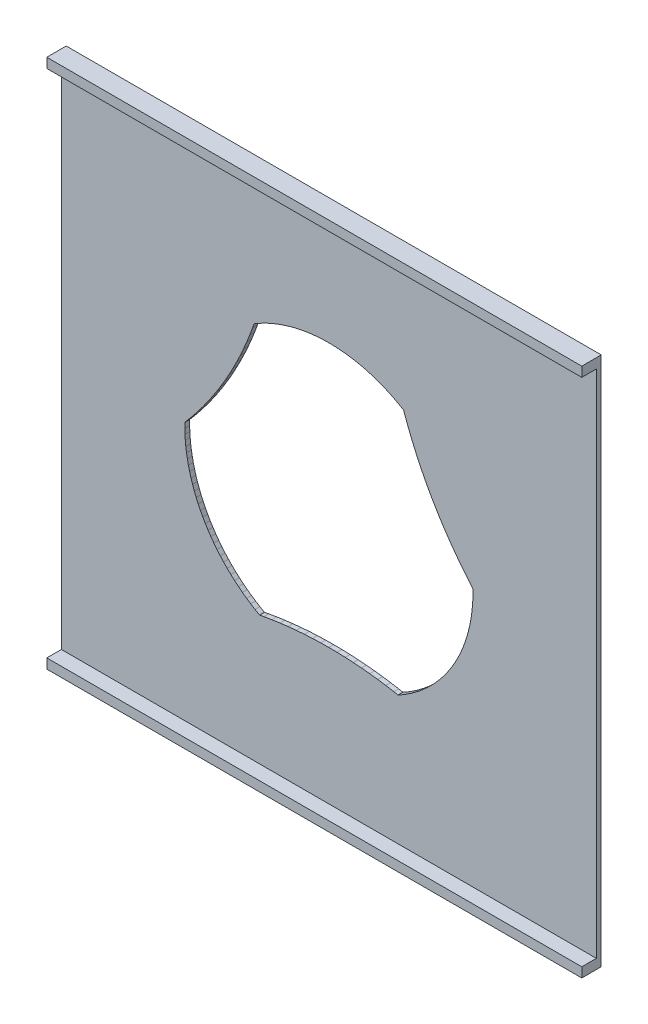
SolidWorks part; units mm, degrees
ref_plane "Front Plane" through (0, 0, 0) normal (0, 0, 1) x (1, 0, 0)
ref_plane "Top Plane" through (0, 0, 0) normal (0, 1, 0) x (1, 0, 0)
ref_plane "Right Plane" through (0, 0, 0) normal (1, 0, 0) x (0, 0, -1)
sketch "Model" plane through (0, 0, 0) normal (0, 0, 1) x (1, 0, 0)
  line L0 (85.0451, -153.4533) -> (85.1181, -153.5021)
  line L1 (85.1181, -153.5021) -> (85.1669, -153.5751)
  line L2 (85.1669, -153.5751) -> (85.184, -153.6612)
  line L3 (85.184, -153.6612) -> (85.184, -154.1112)
  line L4 (85.184, -154.1112) -> (85.1669, -154.1973)
  line L5 (85.1669, -154.1973) -> (85.1181, -154.2703)
  line L6 (85.1181, -154.2703) -> (85.0451, -154.3191)
  line L7 (85.0451, -154.3191) -> (84.959, -154.3362)
  line L8 (84.959, -154.3362) -> (84.459, -154.3362)
  line L9 (84.459, -154.3362) -> (84.3729, -154.3191)
  line L10 (84.3729, -154.3191) -> (84.2999, -154.2703)
  line L11 (84.2999, -154.2703) -> (84.2511, -154.1973)
  line L12 (84.2511, -154.1973) -> (84.234, -154.1112)
  line L13 (84.234, -154.1112) -> (84.234, -153.6612)
  line L14 (84.234, -153.6612) -> (84.2511, -153.5751)
  line L15 (84.2511, -153.5751) -> (84.2999, -153.5021)
  line L16 (84.2999, -153.5021) -> (84.3729, -153.4533)
  line L17 (84.3729, -153.4533) -> (84.459, -153.4362)
  line L18 (84.459, -153.4362) -> (84.959, -153.4362)
  line L19 (84.959, -153.4362) -> (85.0451, -153.4533)
  line L20 (86.5183, -153.4533) -> (86.5913, -153.5021)
  line L21 (86.5913, -153.5021) -> (86.6401, -153.5751)
  line L22 (86.6401, -153.5751) -> (86.6572, -153.6612)
  line L23 (86.6572, -153.6612) -> (86.6572, -154.1112)
  line L24 (86.6572, -154.1112) -> (86.6401, -154.1973)
  line L25 (86.6401, -154.1973) -> (86.5913, -154.2703)
  line L26 (86.5913, -154.2703) -> (86.5183, -154.3191)
  line L27 (86.5183, -154.3191) -> (86.4322, -154.3362)
  line L28 (86.4322, -154.3362) -> (85.9322, -154.3362)
  line L29 (85.9322, -154.3362) -> (85.8461, -154.3191)
  line L30 (85.8461, -154.3191) -> (85.7731, -154.2703)
  line L31 (85.7731, -154.2703) -> (85.7243, -154.1973)
  line L32 (85.7243, -154.1973) -> (85.7072, -154.1112)
  line L33 (85.7072, -154.1112) -> (85.7072, -153.6612)
  line L34 (85.7072, -153.6612) -> (85.7243, -153.5751)
  line L35 (85.7243, -153.5751) -> (85.7731, -153.5021)
  line L36 (85.7731, -153.5021) -> (85.8461, -153.4533)
  line L37 (85.8461, -153.4533) -> (85.9322, -153.4362)
  line L38 (85.9322, -153.4362) -> (86.4322, -153.4362)
  line L39 (86.4322, -153.4362) -> (86.5183, -153.4533)
  line L40 (87.9915, -153.4533) -> (88.0645, -153.5021)
  line L41 (88.0645, -153.5021) -> (88.1133, -153.5751)
  line L42 (88.1133, -153.5751) -> (88.1304, -153.6612)
  line L43 (88.1304, -153.6612) -> (88.1304, -154.1112)
  line L44 (88.1304, -154.1112) -> (88.1133, -154.1973)
  line L45 (88.1133, -154.1973) -> (88.0645, -154.2703)
  line L46 (88.0645, -154.2703) -> (87.9915, -154.3191)
  line L47 (87.9915, -154.3191) -> (87.9054, -154.3362)
  line L48 (87.9054, -154.3362) -> (87.4054, -154.3362)
  line L49 (87.4054, -154.3362) -> (87.3193, -154.3191)
  line L50 (87.3193, -154.3191) -> (87.2463, -154.2703)
  line L51 (87.2463, -154.2703) -> (87.1975, -154.1973)
  line L52 (87.1975, -154.1973) -> (87.1804, -154.1112)
  line L53 (87.1804, -154.1112) -> (87.1804, -153.6612)
  line L54 (87.1804, -153.6612) -> (87.1975, -153.5751)
  line L55 (87.1975, -153.5751) -> (87.2463, -153.5021)
  line L56 (87.2463, -153.5021) -> (87.3193, -153.4533)
  line L57 (87.3193, -153.4533) -> (87.4054, -153.4362)
  line L58 (87.4054, -153.4362) -> (87.9054, -153.4362)
  line L59 (87.9054, -153.4362) -> (87.9915, -153.4533)
  line L60 (81.0387, -153.9414) -> (80.4037, -153.9414)
  line L61 (80.4037, -153.9414) -> (80.4037, -153.4334)
  line L62 (80.4037, -153.4334) -> (81.0387, -153.4334)
  line L63 (81.0387, -153.4334) -> (81.0387, -153.9414)
  line L64 (83.0199, -153.9414) -> (82.3849, -153.9414)
  line L65 (82.3849, -153.9414) -> (82.3849, -153.4334)
  line L66 (82.3849, -153.4334) -> (83.0199, -153.4334)
  line L67 (83.0199, -153.4334) -> (83.0199, -153.9414)
  line L68 (76.0495, -151.9728) -> (76.1306, -152.027)
  line L69 (76.1306, -152.027) -> (76.1848, -152.1081)
  line L70 (76.1848, -152.1081) -> (76.2038, -152.2038)
  line L71 (76.2038, -152.2038) -> (76.2038, -152.8538)
  line L72 (76.2038, -152.8538) -> (76.1848, -152.9495)
  line L73 (76.1848, -152.9495) -> (76.1306, -153.0306)
  line L74 (76.1306, -153.0306) -> (76.0495, -153.0848)
  line L75 (76.0495, -153.0848) -> (75.9538, -153.1038)
  line L76 (75.9538, -153.1038) -> (73.7538, -153.1038)
  line L77 (73.7538, -153.1038) -> (73.6581, -153.0848)
  line L78 (73.6581, -153.0848) -> (73.577, -153.0306)
  line L79 (73.577, -153.0306) -> (73.5228, -152.9495)
  line L80 (73.5228, -152.9495) -> (73.5038, -152.8538)
  line L81 (73.5038, -152.8538) -> (73.5038, -152.2038)
  line L82 (73.5038, -152.2038) -> (73.5228, -152.1081)
  line L83 (73.5228, -152.1081) -> (73.577, -152.027)
  line L84 (73.577, -152.027) -> (73.6581, -151.9728)
  line L85 (73.6581, -151.9728) -> (73.7538, -151.9538)
  line L86 (73.7538, -151.9538) -> (75.9538, -151.9538)
  line L87 (75.9538, -151.9538) -> (76.0495, -151.9728)
  line L88 (81.0387, -152.9414) -> (80.4037, -152.9414)
  line L89 (80.4037, -152.9414) -> (80.4037, -152.4334)
  line L90 (80.4037, -152.4334) -> (81.0387, -152.4334)
  line L91 (81.0387, -152.4334) -> (81.0387, -152.9414)
  line L92 (83.0199, -152.9414) -> (82.3849, -152.9414)
  line L93 (82.3849, -152.9414) -> (82.3849, -152.4334)
  line L94 (82.3849, -152.4334) -> (83.0199, -152.4334)
  line L95 (83.0199, -152.4334) -> (83.0199, -152.9414)
  line L96 (85.0451, -151.9033) -> (85.1181, -151.9521)
  line L97 (85.1181, -151.9521) -> (85.1669, -152.0251)
  line L98 (85.1669, -152.0251) -> (85.184, -152.1112)
  line L99 (85.184, -152.1112) -> (85.184, -152.5612)
  line L100 (85.184, -152.5612) -> (85.1669, -152.6473)
  line L101 (85.1669, -152.6473) -> (85.1181, -152.7203)
  line L102 (85.1181, -152.7203) -> (85.0451, -152.7691)
  line L103 (85.0451, -152.7691) -> (84.959, -152.7862)
  line L104 (84.959, -152.7862) -> (84.459, -152.7862)
  line L105 (84.459, -152.7862) -> (84.3729, -152.7691)
  line L106 (84.3729, -152.7691) -> (84.2999, -152.7203)
  line L107 (84.2999, -152.7203) -> (84.2511, -152.6473)
  line L108 (84.2511, -152.6473) -> (84.234, -152.5612)
  line L109 (84.234, -152.5612) -> (84.234, -152.1112)
  line L110 (84.234, -152.1112) -> (84.2511, -152.0251)
  line L111 (84.2511, -152.0251) -> (84.2999, -151.9521)
  line L112 (84.2999, -151.9521) -> (84.3729, -151.9033)
  line L113 (84.3729, -151.9033) -> (84.459, -151.8862)
  line L114 (84.459, -151.8862) -> (84.959, -151.8862)
  line L115 (84.959, -151.8862) -> (85.0451, -151.9033)
  line L116 (86.5183, -151.9033) -> (86.5913, -151.9521)
  line L117 (86.5913, -151.9521) -> (86.6401, -152.0251)
  line L118 (86.6401, -152.0251) -> (86.6572, -152.1112)
  line L119 (86.6572, -152.1112) -> (86.6572, -152.5612)
  line L120 (86.6572, -152.5612) -> (86.6401, -152.6473)
  line L121 (86.6401, -152.6473) -> (86.5913, -152.7203)
  line L122 (86.5913, -152.7203) -> (86.5183, -152.7691)
  line L123 (86.5183, -152.7691) -> (86.4322, -152.7862)
  line L124 (86.4322, -152.7862) -> (85.9322, -152.7862)
  line L125 (85.9322, -152.7862) -> (85.8461, -152.7691)
  line L126 (85.8461, -152.7691) -> (85.7731, -152.7203)
  line L127 (85.7731, -152.7203) -> (85.7243, -152.6473)
  line L128 (85.7243, -152.6473) -> (85.7072, -152.5612)
  line L129 (85.7072, -152.5612) -> (85.7072, -152.1112)
  line L130 (85.7072, -152.1112) -> (85.7243, -152.0251)
  line L131 (85.7243, -152.0251) -> (85.7731, -151.9521)
  line L132 (85.7731, -151.9521) -> (85.8461, -151.9033)
  line L133 (85.8461, -151.9033) -> (85.9322, -151.8862)
  line L134 (85.9322, -151.8862) -> (86.4322, -151.8862)
  line L135 (86.4322, -151.8862) -> (86.5183, -151.9033)
  line L136 (87.9915, -151.9033) -> (88.0645, -151.9521)
  line L137 (88.0645, -151.9521) -> (88.1133, -152.0251)
  line L138 (88.1133, -152.0251) -> (88.1304, -152.1112)
  line L139 (88.1304, -152.1112) -> (88.1304, -152.5612)
  line L140 (88.1304, -152.5612) -> (88.1133, -152.6473)
  line L141 (88.1133, -152.6473) -> (88.0645, -152.7203)
  line L142 (88.0645, -152.7203) -> (87.9915, -152.7691)
  line L143 (87.9915, -152.7691) -> (87.9054, -152.7862)
  line L144 (87.9054, -152.7862) -> (87.4054, -152.7862)
  line L145 (87.4054, -152.7862) -> (87.3193, -152.7691)
  line L146 (87.3193, -152.7691) -> (87.2463, -152.7203)
  line L147 (87.2463, -152.7203) -> (87.1975, -152.6473)
  line L148 (87.1975, -152.6473) -> (87.1804, -152.5612)
  line L149 (87.1804, -152.5612) -> (87.1804, -152.1112)
  line L150 (87.1804, -152.1112) -> (87.1975, -152.0251)
  line L151 (87.1975, -152.0251) -> (87.2463, -151.9521)
  line L152 (87.2463, -151.9521) -> (87.3193, -151.9033)
  line L153 (87.3193, -151.9033) -> (87.4054, -151.8862)
  line L154 (87.4054, -151.8862) -> (87.9054, -151.8862)
  line L155 (87.9054, -151.8862) -> (87.9915, -151.9033)
  line L156 (89.4647, -150.4947) -> (89.5377, -150.5435)
  line L157 (89.5377, -150.5435) -> (89.5865, -150.6165)
  line L158 (89.5865, -150.6165) -> (89.6036, -150.7026)
  line L159 (89.6036, -150.7026) -> (89.6036, -151.1526)
  line L160 (89.6036, -151.1526) -> (89.5865, -151.2387)
  line L161 (89.5865, -151.2387) -> (89.5377, -151.3117)
  line L162 (89.5377, -151.3117) -> (89.4647, -151.3605)
  line L163 (89.4647, -151.3605) -> (89.3786, -151.3776)
  line L164 (89.3786, -151.3776) -> (88.8786, -151.3776)
  line L165 (88.8786, -151.3776) -> (88.7925, -151.3605)
  line L166 (88.7925, -151.3605) -> (88.7195, -151.3117)
  line L167 (88.7195, -151.3117) -> (88.6707, -151.2387)
  line L168 (88.6707, -151.2387) -> (88.6536, -151.1526)
  line L169 (88.6536, -151.1526) -> (88.6536, -150.7026)
  line L170 (88.6536, -150.7026) -> (88.6707, -150.6165)
  line L171 (88.6707, -150.6165) -> (88.7195, -150.5435)
  line L172 (88.7195, -150.5435) -> (88.7925, -150.4947)
  line L173 (88.7925, -150.4947) -> (88.8786, -150.4776)
  line L174 (88.8786, -150.4776) -> (89.3786, -150.4776)
  line L175 (89.3786, -150.4776) -> (89.4647, -150.4947)
  line L176 (92.9951, -150.5928) -> (93.06, -150.6362)
  line L177 (93.06, -150.6362) -> (93.1033, -150.7011)
  line L178 (93.1033, -150.7011) -> (93.1185, -150.7776)
  line L179 (93.1185, -150.7776) -> (93.1185, -151.1776)
  line L180 (93.1185, -151.1776) -> (93.1033, -151.2541)
  line L181 (93.1033, -151.2541) -> (93.06, -151.319)
  line L182 (93.06, -151.319) -> (92.9951, -151.3624)
  line L183 (92.9951, -151.3624) -> (92.9185, -151.3776)
  line L184 (92.9185, -151.3776) -> (92.3685, -151.3776)
  line L185 (92.3685, -151.3776) -> (92.292, -151.3624)
  line L186 (92.292, -151.3624) -> (92.2271, -151.319)
  line L187 (92.2271, -151.319) -> (92.1838, -151.2541)
  line L188 (92.1838, -151.2541) -> (92.1685, -151.1776)
  line L189 (92.1685, -151.1776) -> (92.1685, -150.7776)
  line L190 (92.1685, -150.7776) -> (92.1838, -150.7011)
  line L191 (92.1838, -150.7011) -> (92.2271, -150.6362)
  line L192 (92.2271, -150.6362) -> (92.292, -150.5928)
  line L193 (92.292, -150.5928) -> (92.3685, -150.5776)
  line L194 (92.3685, -150.5776) -> (92.9185, -150.5776)
  line L195 (92.9185, -150.5776) -> (92.9951, -150.5928)
  line L196 (94.7125, -150.5928) -> (94.7774, -150.6362)
  line L197 (94.7774, -150.6362) -> (94.8208, -150.7011)
  line L198 (94.8208, -150.7011) -> (94.836, -150.7776)
  line L199 (94.836, -150.7776) -> (94.836, -151.1776)
  line L200 (94.836, -151.1776) -> (94.8208, -151.2541)
  line L201 (94.8208, -151.2541) -> (94.7774, -151.319)
  line L202 (94.7774, -151.319) -> (94.7125, -151.3624)
  line L203 (94.7125, -151.3624) -> (94.636, -151.3776)
  line L204 (94.636, -151.3776) -> (94.086, -151.3776)
  line L205 (94.086, -151.3776) -> (94.0095, -151.3624)
  line L206 (94.0095, -151.3624) -> (93.9446, -151.319)
  line L207 (93.9446, -151.319) -> (93.9012, -151.2541)
  line L208 (93.9012, -151.2541) -> (93.886, -151.1776)
  line L209 (93.886, -151.1776) -> (93.886, -150.7776)
  line L210 (93.886, -150.7776) -> (93.9012, -150.7011)
  line L211 (93.9012, -150.7011) -> (93.9446, -150.6362)
  line L212 (93.9446, -150.6362) -> (94.0095, -150.5928)
  line L213 (94.0095, -150.5928) -> (94.086, -150.5776)
  line L214 (94.086, -150.5776) -> (94.636, -150.5776)
  line L215 (94.636, -150.5776) -> (94.7125, -150.5928)
  line L216 (80.6409, -150.5796) -> (80.7058, -150.623)
  line L217 (80.7058, -150.623) -> (80.7492, -150.6879)
  line L218 (80.7492, -150.6879) -> (80.7644, -150.7644)
  line L219 (80.7644, -150.7644) -> (80.7644, -151.1644)
  line L220 (80.7644, -151.1644) -> (80.7492, -151.2409)
  line L221 (80.7492, -151.2409) -> (80.7058, -151.3058)
  line L222 (80.7058, -151.3058) -> (80.6409, -151.3492)
  line L223 (80.6409, -151.3492) -> (80.5644, -151.3644)
  line L224 (80.5644, -151.3644) -> (80.0144, -151.3644)
  line L225 (80.0144, -151.3644) -> (79.9379, -151.3492)
  line L226 (79.9379, -151.3492) -> (79.873, -151.3058)
  line L227 (79.873, -151.3058) -> (79.8296, -151.2409)
  line L228 (79.8296, -151.2409) -> (79.8144, -151.1644)
  line L229 (79.8144, -151.1644) -> (79.8144, -150.7644)
  line L230 (79.8144, -150.7644) -> (79.8296, -150.6879)
  line L231 (79.8296, -150.6879) -> (79.873, -150.623)
  line L232 (79.873, -150.623) -> (79.9379, -150.5796)
  line L233 (79.9379, -150.5796) -> (80.0144, -150.5644)
  line L234 (80.0144, -150.5644) -> (80.5644, -150.5644)
  line L235 (80.5644, -150.5644) -> (80.6409, -150.5796)
  line L236 (82.1141, -150.5796) -> (82.179, -150.623)
  line L237 (82.179, -150.623) -> (82.2224, -150.6879)
  line L238 (82.2224, -150.6879) -> (82.2376, -150.7644)
  line L239 (82.2376, -150.7644) -> (82.2376, -151.1644)
  line L240 (82.2376, -151.1644) -> (82.2224, -151.2409)
  line L241 (82.2224, -151.2409) -> (82.179, -151.3058)
  line L242 (82.179, -151.3058) -> (82.1141, -151.3492)
  line L243 (82.1141, -151.3492) -> (82.0376, -151.3644)
  line L244 (82.0376, -151.3644) -> (81.4876, -151.3644)
  line L245 (81.4876, -151.3644) -> (81.4111, -151.3492)
  line L246 (81.4111, -151.3492) -> (81.3462, -151.3058)
  line L247 (81.3462, -151.3058) -> (81.3028, -151.2409)
  line L248 (81.3028, -151.2409) -> (81.2876, -151.1644)
  line L249 (81.2876, -151.1644) -> (81.2876, -150.7644)
  line L250 (81.2876, -150.7644) -> (81.3028, -150.6879)
  line L251 (81.3028, -150.6879) -> (81.3462, -150.623)
  line L252 (81.3462, -150.623) -> (81.4111, -150.5796)
  line L253 (81.4111, -150.5796) -> (81.4876, -150.5644)
  line L254 (81.4876, -150.5644) -> (82.0376, -150.5644)
  line L255 (82.0376, -150.5644) -> (82.1141, -150.5796)
  line L256 (83.5873, -150.5796) -> (83.6522, -150.623)
  line L257 (83.6522, -150.623) -> (83.6956, -150.6879)
  line L258 (83.6956, -150.6879) -> (83.7108, -150.7644)
  line L259 (83.7108, -150.7644) -> (83.7108, -151.1644)
  line L260 (83.7108, -151.1644) -> (83.6956, -151.2409)
  line L261 (83.6956, -151.2409) -> (83.6522, -151.3058)
  line L262 (83.6522, -151.3058) -> (83.5873, -151.3492)
  line L263 (83.5873, -151.3492) -> (83.5108, -151.3644)
  line L264 (83.5108, -151.3644) -> (82.9608, -151.3644)
  line L265 (82.9608, -151.3644) -> (82.8843, -151.3492)
  line L266 (82.8843, -151.3492) -> (82.8194, -151.3058)
  line L267 (82.8194, -151.3058) -> (82.776, -151.2409)
  line L268 (82.776, -151.2409) -> (82.7608, -151.1644)
  line L269 (82.7608, -151.1644) -> (82.7608, -150.7644)
  line L270 (82.7608, -150.7644) -> (82.776, -150.6879)
  line L271 (82.776, -150.6879) -> (82.8194, -150.623)
  line L272 (82.8194, -150.623) -> (82.8843, -150.5796)
  line L273 (82.8843, -150.5796) -> (82.9608, -150.5644)
  line L274 (82.9608, -150.5644) -> (83.5108, -150.5644)
  line L275 (83.5108, -150.5644) -> (83.5873, -150.5796)
  line L276 (85.0605, -150.5796) -> (85.1254, -150.623)
  line L277 (85.1254, -150.623) -> (85.1688, -150.6879)
  line L278 (85.1688, -150.6879) -> (85.184, -150.7644)
  line L279 (85.184, -150.7644) -> (85.184, -151.1644)
  line L280 (85.184, -151.1644) -> (85.1688, -151.2409)
  line L281 (85.1688, -151.2409) -> (85.1254, -151.3058)
  line L282 (85.1254, -151.3058) -> (85.0605, -151.3492)
  line L283 (85.0605, -151.3492) -> (84.984, -151.3644)
  line L284 (84.984, -151.3644) -> (84.434, -151.3644)
  line L285 (84.434, -151.3644) -> (84.3575, -151.3492)
  line L286 (84.3575, -151.3492) -> (84.2926, -151.3058)
  line L287 (84.2926, -151.3058) -> (84.2492, -151.2409)
  line L288 (84.2492, -151.2409) -> (84.234, -151.1644)
  line L289 (84.234, -151.1644) -> (84.234, -150.7644)
  line L290 (84.234, -150.7644) -> (84.2492, -150.6879)
  line L291 (84.2492, -150.6879) -> (84.2926, -150.623)
  line L292 (84.2926, -150.623) -> (84.3575, -150.5796)
  line L293 (84.3575, -150.5796) -> (84.434, -150.5644)
  line L294 (84.434, -150.5644) -> (84.984, -150.5644)
  line L295 (84.984, -150.5644) -> (85.0605, -150.5796)
  line L296 (86.5337, -150.5796) -> (86.5986, -150.623)
  line L297 (86.5986, -150.623) -> (86.642, -150.6879)
  line L298 (86.642, -150.6879) -> (86.6572, -150.7644)
  line L299 (86.6572, -150.7644) -> (86.6572, -151.1644)
  line L300 (86.6572, -151.1644) -> (86.642, -151.2409)
  line L301 (86.642, -151.2409) -> (86.5986, -151.3058)
  line L302 (86.5986, -151.3058) -> (86.5337, -151.3492)
  line L303 (86.5337, -151.3492) -> (86.4572, -151.3644)
  line L304 (86.4572, -151.3644) -> (85.9072, -151.3644)
  line L305 (85.9072, -151.3644) -> (85.8307, -151.3492)
  line L306 (85.8307, -151.3492) -> (85.7658, -151.3058)
  line L307 (85.7658, -151.3058) -> (85.7224, -151.2409)
  line L308 (85.7224, -151.2409) -> (85.7072, -151.1644)
  line L309 (85.7072, -151.1644) -> (85.7072, -150.7644)
  line L310 (85.7072, -150.7644) -> (85.7224, -150.6879)
  line L311 (85.7224, -150.6879) -> (85.7658, -150.623)
  line L312 (85.7658, -150.623) -> (85.8307, -150.5796)
  line L313 (85.8307, -150.5796) -> (85.9072, -150.5644)
  line L314 (85.9072, -150.5644) -> (86.4572, -150.5644)
  line L315 (86.4572, -150.5644) -> (86.5337, -150.5796)
  line L316 (88.0069, -150.5796) -> (88.0718, -150.623)
  line L317 (88.0718, -150.623) -> (88.1152, -150.6879)
  line L318 (88.1152, -150.6879) -> (88.1304, -150.7644)
  line L319 (88.1304, -150.7644) -> (88.1304, -151.1644)
  line L320 (88.1304, -151.1644) -> (88.1152, -151.2409)
  line L321 (88.1152, -151.2409) -> (88.0718, -151.3058)
  line L322 (88.0718, -151.3058) -> (88.0069, -151.3492)
  line L323 (88.0069, -151.3492) -> (87.9304, -151.3644)
  line L324 (87.9304, -151.3644) -> (87.3804, -151.3644)
  line L325 (87.3804, -151.3644) -> (87.3039, -151.3492)
  line L326 (87.3039, -151.3492) -> (87.239, -151.3058)
  line L327 (87.239, -151.3058) -> (87.1956, -151.2409)
  line L328 (87.1956, -151.2409) -> (87.1804, -151.1644)
  line L329 (87.1804, -151.1644) -> (87.1804, -150.7644)
  line L330 (87.1804, -150.7644) -> (87.1956, -150.6879)
  line L331 (87.1956, -150.6879) -> (87.239, -150.623)
  line L332 (87.239, -150.623) -> (87.3039, -150.5796)
  line L333 (87.3039, -150.5796) -> (87.3804, -150.5644)
  line L334 (87.3804, -150.5644) -> (87.9304, -150.5644)
  line L335 (87.9304, -150.5644) -> (88.0069, -150.5796)
  line L336 (91.226, -150.4993) -> (91.297, -150.5467)
  line L337 (91.297, -150.5467) -> (91.3444, -150.6176)
  line L338 (91.3444, -150.6176) -> (91.3611, -150.7013)
  line L339 (91.3611, -150.7013) -> (91.3611, -151.1388)
  line L340 (91.3611, -151.1388) -> (91.3444, -151.2226)
  line L341 (91.3444, -151.2226) -> (91.297, -151.2935)
  line L342 (91.297, -151.2935) -> (91.226, -151.3409)
  line L343 (91.226, -151.3409) -> (91.1423, -151.3576)
  line L344 (91.1423, -151.3576) -> (90.6298, -151.3576)
  line L345 (90.6298, -151.3576) -> (90.5461, -151.3409)
  line L346 (90.5461, -151.3409) -> (90.4751, -151.2935)
  line L347 (90.4751, -151.2935) -> (90.4277, -151.2226)
  line L348 (90.4277, -151.2226) -> (90.4111, -151.1388)
  line L349 (90.4111, -151.1388) -> (90.4111, -150.7013)
  line L350 (90.4111, -150.7013) -> (90.4277, -150.6176)
  line L351 (90.4277, -150.6176) -> (90.4751, -150.5467)
  line L352 (90.4751, -150.5467) -> (90.5461, -150.4993)
  line L353 (90.5461, -150.4993) -> (90.6298, -150.4826)
  line L354 (90.6298, -150.4826) -> (91.1423, -150.4826)
  line L355 (91.1423, -150.4826) -> (91.226, -150.4993)
  line L356 (70.4655, -150.3545) -> (70.5385, -150.4033)
  line L357 (70.5385, -150.4033) -> (70.5873, -150.4763)
  line L358 (70.5873, -150.4763) -> (70.6044, -150.5624)
  line L359 (70.6044, -150.5624) -> (70.6044, -151.0124)
  line L360 (70.6044, -151.0124) -> (70.5873, -151.0985)
  line L361 (70.5873, -151.0985) -> (70.5385, -151.1715)
  line L362 (70.5385, -151.1715) -> (70.4655, -151.2203)
  line L363 (70.4655, -151.2203) -> (70.3794, -151.2374)
  line L364 (70.3794, -151.2374) -> (69.8794, -151.2374)
  line L365 (69.8794, -151.2374) -> (69.7933, -151.2203)
  line L366 (69.7933, -151.2203) -> (69.7203, -151.1715)
  line L367 (69.7203, -151.1715) -> (69.6715, -151.0985)
  line L368 (69.6715, -151.0985) -> (69.6544, -151.0124)
  line L369 (69.6544, -151.0124) -> (69.6544, -150.5624)
  line L370 (69.6544, -150.5624) -> (69.6715, -150.4763)
  line L371 (69.6715, -150.4763) -> (69.7203, -150.4033)
  line L372 (69.7203, -150.4033) -> (69.7933, -150.3545)
  line L373 (69.7933, -150.3545) -> (69.8794, -150.3374)
  line L374 (69.8794, -150.3374) -> (70.3794, -150.3374)
  line L375 (70.3794, -150.3374) -> (70.4655, -150.3545)
  line L376 (77.8315, -149.8087) -> (77.9045, -149.8575)
  line L377 (77.9045, -149.8575) -> (77.9533, -149.9305)
  line L378 (77.9533, -149.9305) -> (77.9704, -150.0166)
  line L379 (77.9704, -150.0166) -> (77.9704, -150.4666)
  line L380 (77.9704, -150.4666) -> (77.9533, -150.5527)
  line L381 (77.9533, -150.5527) -> (77.9045, -150.6257)
  line L382 (77.9045, -150.6257) -> (77.8315, -150.6745)
  line L383 (77.8315, -150.6745) -> (77.7454, -150.6916)
  line L384 (77.7454, -150.6916) -> (77.2454, -150.6916)
  line L385 (77.2454, -150.6916) -> (77.1593, -150.6745)
  line L386 (77.1593, -150.6745) -> (77.0863, -150.6257)
  line L387 (77.0863, -150.6257) -> (77.0375, -150.5527)
  line L388 (77.0375, -150.5527) -> (77.0204, -150.4666)
  line L389 (77.0204, -150.4666) -> (77.0204, -150.0166)
  line L390 (77.0204, -150.0166) -> (77.0375, -149.9305)
  line L391 (77.0375, -149.9305) -> (77.0863, -149.8575)
  line L392 (77.0863, -149.8575) -> (77.1593, -149.8087)
  line L393 (77.1593, -149.8087) -> (77.2454, -149.7916)
  line L394 (77.2454, -149.7916) -> (77.7454, -149.7916)
  line L395 (77.7454, -149.7916) -> (77.8315, -149.8087)
  line L396 (76.0495, -149.0228) -> (76.1306, -149.077)
  line L397 (76.1306, -149.077) -> (76.1848, -149.1581)
  line L398 (76.1848, -149.1581) -> (76.2038, -149.2538)
  line L399 (76.2038, -149.2538) -> (76.2038, -149.9038)
  line L400 (76.2038, -149.9038) -> (76.1848, -149.9995)
  line L401 (76.1848, -149.9995) -> (76.1306, -150.0806)
  line L402 (76.1306, -150.0806) -> (76.0495, -150.1348)
  line L403 (76.0495, -150.1348) -> (75.9538, -150.1538)
  line L404 (75.9538, -150.1538) -> (73.7538, -150.1538)
  line L405 (73.7538, -150.1538) -> (73.6581, -150.1348)
  line L406 (73.6581, -150.1348) -> (73.577, -150.0806)
  line L407 (73.577, -150.0806) -> (73.5228, -149.9995)
  line L408 (73.5228, -149.9995) -> (73.5038, -149.9038)
  line L409 (73.5038, -149.9038) -> (73.5038, -149.2538)
  line L410 (73.5038, -149.2538) -> (73.5228, -149.1581)
  line L411 (73.5228, -149.1581) -> (73.577, -149.077)
  line L412 (73.577, -149.077) -> (73.6581, -149.0228)
  line L413 (73.6581, -149.0228) -> (73.7538, -149.0038)
  line L414 (73.7538, -149.0038) -> (75.9538, -149.0038)
  line L415 (75.9538, -149.0038) -> (76.0495, -149.0228)
  line L416 (89.4647, -148.9447) -> (89.5377, -148.9935)
  line L417 (89.5377, -148.9935) -> (89.5865, -149.0665)
  line L418 (89.5865, -149.0665) -> (89.6036, -149.1526)
  line L419 (89.6036, -149.1526) -> (89.6036, -149.6026)
  line L420 (89.6036, -149.6026) -> (89.5865, -149.6887)
  line L421 (89.5865, -149.6887) -> (89.5377, -149.7617)
  line L422 (89.5377, -149.7617) -> (89.4647, -149.8105)
  line L423 (89.4647, -149.8105) -> (89.3786, -149.8276)
  line L424 (89.3786, -149.8276) -> (88.8786, -149.8276)
  line L425 (88.8786, -149.8276) -> (88.7925, -149.8105)
  line L426 (88.7925, -149.8105) -> (88.7195, -149.7617)
  line L427 (88.7195, -149.7617) -> (88.6707, -149.6887)
  line L428 (88.6707, -149.6887) -> (88.6536, -149.6026)
  line L429 (88.6536, -149.6026) -> (88.6536, -149.1526)
  line L430 (88.6536, -149.1526) -> (88.6707, -149.0665)
  line L431 (88.6707, -149.0665) -> (88.7195, -148.9935)
  line L432 (88.7195, -148.9935) -> (88.7925, -148.9447)
  line L433 (88.7925, -148.9447) -> (88.8786, -148.9276)
  line L434 (88.8786, -148.9276) -> (89.3786, -148.9276)
  line L435 (89.3786, -148.9276) -> (89.4647, -148.9447)
  line L436 (91.226, -148.9243) -> (91.297, -148.9717)
  line L437 (91.297, -148.9717) -> (91.3444, -149.0426)
  line L438 (91.3444, -149.0426) -> (91.3611, -149.1264)
  line L439 (91.3611, -149.1264) -> (91.3611, -149.5639)
  line L440 (91.3611, -149.5639) -> (91.3444, -149.6476)
  line L441 (91.3444, -149.6476) -> (91.297, -149.7185)
  line L442 (91.297, -149.7185) -> (91.226, -149.7659)
  line L443 (91.226, -149.7659) -> (91.1423, -149.7826)
  line L444 (91.1423, -149.7826) -> (90.6298, -149.7826)
  line L445 (90.6298, -149.7826) -> (90.5461, -149.7659)
  line L446 (90.5461, -149.7659) -> (90.4751, -149.7185)
  line L447 (90.4751, -149.7185) -> (90.4277, -149.6476)
  line L448 (90.4277, -149.6476) -> (90.4111, -149.5639)
  line L449 (90.4111, -149.5639) -> (90.4111, -149.1264)
  line L450 (90.4111, -149.1264) -> (90.4277, -149.0426)
  line L451 (90.4277, -149.0426) -> (90.4751, -148.9717)
  line L452 (90.4751, -148.9717) -> (90.5461, -148.9243)
  line L453 (90.5461, -148.9243) -> (90.6298, -148.9076)
  line L454 (90.6298, -148.9076) -> (91.1423, -148.9076)
  line L455 (91.1423, -148.9076) -> (91.226, -148.9243)
  line L456 (92.9951, -148.9428) -> (93.06, -148.9862)
  line L457 (93.06, -148.9862) -> (93.1033, -149.0511)
  line L458 (93.1033, -149.0511) -> (93.1185, -149.1276)
  line L459 (93.1185, -149.1276) -> (93.1185, -149.5276)
  line L460 (93.1185, -149.5276) -> (93.1033, -149.6041)
  line L461 (93.1033, -149.6041) -> (93.06, -149.669)
  line L462 (93.06, -149.669) -> (92.9951, -149.7124)
  line L463 (92.9951, -149.7124) -> (92.9185, -149.7276)
  line L464 (92.9185, -149.7276) -> (92.3685, -149.7276)
  line L465 (92.3685, -149.7276) -> (92.292, -149.7124)
  line L466 (92.292, -149.7124) -> (92.2271, -149.669)
  line L467 (92.2271, -149.669) -> (92.1838, -149.6041)
  line L468 (92.1838, -149.6041) -> (92.1685, -149.5276)
  line L469 (92.1685, -149.5276) -> (92.1685, -149.1276)
  line L470 (92.1685, -149.1276) -> (92.1838, -149.0511)
  line L471 (92.1838, -149.0511) -> (92.2271, -148.9862)
  line L472 (92.2271, -148.9862) -> (92.292, -148.9428)
  line L473 (92.292, -148.9428) -> (92.3685, -148.9276)
  line L474 (92.3685, -148.9276) -> (92.9185, -148.9276)
  line L475 (92.9185, -148.9276) -> (92.9951, -148.9428)
  line L476 (94.7125, -148.9428) -> (94.7774, -148.9862)
  line L477 (94.7774, -148.9862) -> (94.8208, -149.0511)
  line L478 (94.8208, -149.0511) -> (94.836, -149.1276)
  line L479 (94.836, -149.1276) -> (94.836, -149.5276)
  line L480 (94.836, -149.5276) -> (94.8208, -149.6041)
  line L481 (94.8208, -149.6041) -> (94.7774, -149.669)
  line L482 (94.7774, -149.669) -> (94.7125, -149.7124)
  line L483 (94.7125, -149.7124) -> (94.636, -149.7276)
  line L484 (94.636, -149.7276) -> (94.086, -149.7276)
  line L485 (94.086, -149.7276) -> (94.0095, -149.7124)
  line L486 (94.0095, -149.7124) -> (93.9446, -149.669)
  line L487 (93.9446, -149.669) -> (93.9012, -149.6041)
  line L488 (93.9012, -149.6041) -> (93.886, -149.5276)
  line L489 (93.886, -149.5276) -> (93.886, -149.1276)
  line L490 (93.886, -149.1276) -> (93.9012, -149.0511)
  line L491 (93.9012, -149.0511) -> (93.9446, -148.9862)
  line L492 (93.9446, -148.9862) -> (94.0095, -148.9428)
  line L493 (94.0095, -148.9428) -> (94.086, -148.9276)
  line L494 (94.086, -148.9276) -> (94.636, -148.9276)
  line L495 (94.636, -148.9276) -> (94.7125, -148.9428)
  line L496 (80.6409, -148.9296) -> (80.7058, -148.973)
  line L497 (80.7058, -148.973) -> (80.7492, -149.0379)
  line L498 (80.7492, -149.0379) -> (80.7644, -149.1144)
  line L499 (80.7644, -149.1144) -> (80.7644, -149.5144)
  line L500 (80.7644, -149.5144) -> (80.7492, -149.5909)
  line L501 (80.7492, -149.5909) -> (80.7058, -149.6558)
  line L502 (80.7058, -149.6558) -> (80.6409, -149.6992)
  line L503 (80.6409, -149.6992) -> (80.5644, -149.7144)
  line L504 (80.5644, -149.7144) -> (80.0144, -149.7144)
  line L505 (80.0144, -149.7144) -> (79.9379, -149.6992)
  line L506 (79.9379, -149.6992) -> (79.873, -149.6558)
  line L507 (79.873, -149.6558) -> (79.8296, -149.5909)
  line L508 (79.8296, -149.5909) -> (79.8144, -149.5144)
  line L509 (79.8144, -149.5144) -> (79.8144, -149.1144)
  line L510 (79.8144, -149.1144) -> (79.8296, -149.0379)
  line L511 (79.8296, -149.0379) -> (79.873, -148.973)
  line L512 (79.873, -148.973) -> (79.9379, -148.9296)
  line L513 (79.9379, -148.9296) -> (80.0144, -148.9144)
  line L514 (80.0144, -148.9144) -> (80.5644, -148.9144)
  line L515 (80.5644, -148.9144) -> (80.6409, -148.9296)
  line L516 (82.1141, -148.9296) -> (82.179, -148.973)
  line L517 (82.179, -148.973) -> (82.2224, -149.0379)
  line L518 (82.2224, -149.0379) -> (82.2376, -149.1144)
  line L519 (82.2376, -149.1144) -> (82.2376, -149.5144)
  line L520 (82.2376, -149.5144) -> (82.2224, -149.5909)
  line L521 (82.2224, -149.5909) -> (82.179, -149.6558)
  line L522 (82.179, -149.6558) -> (82.1141, -149.6992)
  line L523 (82.1141, -149.6992) -> (82.0376, -149.7144)
  line L524 (82.0376, -149.7144) -> (81.4876, -149.7144)
  line L525 (81.4876, -149.7144) -> (81.4111, -149.6992)
  line L526 (81.4111, -149.6992) -> (81.3462, -149.6558)
  line L527 (81.3462, -149.6558) -> (81.3028, -149.5909)
  line L528 (81.3028, -149.5909) -> (81.2876, -149.5144)
  line L529 (81.2876, -149.5144) -> (81.2876, -149.1144)
  line L530 (81.2876, -149.1144) -> (81.3028, -149.0379)
  line L531 (81.3028, -149.0379) -> (81.3462, -148.973)
  line L532 (81.3462, -148.973) -> (81.4111, -148.9296)
  line L533 (81.4111, -148.9296) -> (81.4876, -148.9144)
  line L534 (81.4876, -148.9144) -> (82.0376, -148.9144)
  line L535 (82.0376, -148.9144) -> (82.1141, -148.9296)
  line L536 (83.5873, -148.9296) -> (83.6522, -148.973)
  line L537 (83.6522, -148.973) -> (83.6956, -149.0379)
  line L538 (83.6956, -149.0379) -> (83.7108, -149.1144)
  line L539 (83.7108, -149.1144) -> (83.7108, -149.5144)
  line L540 (83.7108, -149.5144) -> (83.6956, -149.5909)
  line L541 (83.6956, -149.5909) -> (83.6522, -149.6558)
  line L542 (83.6522, -149.6558) -> (83.5873, -149.6992)
  line L543 (83.5873, -149.6992) -> (83.5108, -149.7144)
  line L544 (83.5108, -149.7144) -> (82.9608, -149.7144)
  line L545 (82.9608, -149.7144) -> (82.8843, -149.6992)
  line L546 (82.8843, -149.6992) -> (82.8194, -149.6558)
  line L547 (82.8194, -149.6558) -> (82.776, -149.5909)
  line L548 (82.776, -149.5909) -> (82.7608, -149.5144)
  line L549 (82.7608, -149.5144) -> (82.7608, -149.1144)
  line L550 (82.7608, -149.1144) -> (82.776, -149.0379)
  line L551 (82.776, -149.0379) -> (82.8194, -148.973)
  line L552 (82.8194, -148.973) -> (82.8843, -148.9296)
  line L553 (82.8843, -148.9296) -> (82.9608, -148.9144)
  line L554 (82.9608, -148.9144) -> (83.5108, -148.9144)
  line L555 (83.5108, -148.9144) -> (83.5873, -148.9296)
  line L556 (85.0605, -148.9296) -> (85.1254, -148.973)
  line L557 (85.1254, -148.973) -> (85.1688, -149.0379)
  line L558 (85.1688, -149.0379) -> (85.184, -149.1144)
  line L559 (85.184, -149.1144) -> (85.184, -149.5144)
  line L560 (85.184, -149.5144) -> (85.1688, -149.5909)
  line L561 (85.1688, -149.5909) -> (85.1254, -149.6558)
  line L562 (85.1254, -149.6558) -> (85.0605, -149.6992)
  line L563 (85.0605, -149.6992) -> (84.984, -149.7144)
  line L564 (84.984, -149.7144) -> (84.434, -149.7144)
  line L565 (84.434, -149.7144) -> (84.3575, -149.6992)
  line L566 (84.3575, -149.6992) -> (84.2926, -149.6558)
  line L567 (84.2926, -149.6558) -> (84.2492, -149.5909)
  line L568 (84.2492, -149.5909) -> (84.234, -149.5144)
  line L569 (84.234, -149.5144) -> (84.234, -149.1144)
  line L570 (84.234, -149.1144) -> (84.2492, -149.0379)
  line L571 (84.2492, -149.0379) -> (84.2926, -148.973)
  line L572 (84.2926, -148.973) -> (84.3575, -148.9296)
  line L573 (84.3575, -148.9296) -> (84.434, -148.9144)
  line L574 (84.434, -148.9144) -> (84.984, -148.9144)
  line L575 (84.984, -148.9144) -> (85.0605, -148.9296)
  line L576 (86.5337, -148.9296) -> (86.5986, -148.973)
  line L577 (86.5986, -148.973) -> (86.642, -149.0379)
  line L578 (86.642, -149.0379) -> (86.6572, -149.1144)
  line L579 (86.6572, -149.1144) -> (86.6572, -149.5144)
  line L580 (86.6572, -149.5144) -> (86.642, -149.5909)
  line L581 (86.642, -149.5909) -> (86.5986, -149.6558)
  line L582 (86.5986, -149.6558) -> (86.5337, -149.6992)
  line L583 (86.5337, -149.6992) -> (86.4572, -149.7144)
  line L584 (86.4572, -149.7144) -> (85.9072, -149.7144)
  line L585 (85.9072, -149.7144) -> (85.8307, -149.6992)
  line L586 (85.8307, -149.6992) -> (85.7658, -149.6558)
  line L587 (85.7658, -149.6558) -> (85.7224, -149.5909)
  line L588 (85.7224, -149.5909) -> (85.7072, -149.5144)
  line L589 (85.7072, -149.5144) -> (85.7072, -149.1144)
  line L590 (85.7072, -149.1144) -> (85.7224, -149.0379)
  line L591 (85.7224, -149.0379) -> (85.7658, -148.973)
  line L592 (85.7658, -148.973) -> (85.8307, -148.9296)
  line L593 (85.8307, -148.9296) -> (85.9072, -148.9144)
  line L594 (85.9072, -148.9144) -> (86.4572, -148.9144)
  line L595 (86.4572, -148.9144) -> (86.5337, -148.9296)
  line L596 (88.0069, -148.9296) -> (88.0718, -148.973)
  line L597 (88.0718, -148.973) -> (88.1152, -149.0379)
  line L598 (88.1152, -149.0379) -> (88.1304, -149.1144)
  line L599 (88.1304, -149.1144) -> (88.1304, -149.5144)
  line L600 (88.1304, -149.5144) -> (88.1152, -149.5909)
  line L601 (88.1152, -149.5909) -> (88.0718, -149.6558)
  line L602 (88.0718, -149.6558) -> (88.0069, -149.6992)
  line L603 (88.0069, -149.6992) -> (87.9304, -149.7144)
  line L604 (87.9304, -149.7144) -> (87.3804, -149.7144)
  line L605 (87.3804, -149.7144) -> (87.3039, -149.6992)
  line L606 (87.3039, -149.6992) -> (87.239, -149.6558)
  line L607 (87.239, -149.6558) -> (87.1956, -149.5909)
  line L608 (87.1956, -149.5909) -> (87.1804, -149.5144)
  line L609 (87.1804, -149.5144) -> (87.1804, -149.1144)
  line L610 (87.1804, -149.1144) -> (87.1956, -149.0379)
  line L611 (87.1956, -149.0379) -> (87.239, -148.973)
  line L612 (87.239, -148.973) -> (87.3039, -148.9296)
  line L613 (87.3039, -148.9296) -> (87.3804, -148.9144)
  line L614 (87.3804, -148.9144) -> (87.9304, -148.9144)
  line L615 (87.9304, -148.9144) -> (88.0069, -148.9296)
  line L616 (70.4655, -148.8045) -> (70.5385, -148.8533)
  line L617 (70.5385, -148.8533) -> (70.5873, -148.9263)
  line L618 (70.5873, -148.9263) -> (70.6044, -149.0124)
  line L619 (70.6044, -149.0124) -> (70.6044, -149.4624)
  line L620 (70.6044, -149.4624) -> (70.5873, -149.5485)
  line L621 (70.5873, -149.5485) -> (70.5385, -149.6215)
  line L622 (70.5385, -149.6215) -> (70.4655, -149.6703)
  line L623 (70.4655, -149.6703) -> (70.3794, -149.6874)
  line L624 (70.3794, -149.6874) -> (69.8794, -149.6874)
  line L625 (69.8794, -149.6874) -> (69.7933, -149.6703)
  line L626 (69.7933, -149.6703) -> (69.7203, -149.6215)
  line L627 (69.7203, -149.6215) -> (69.6715, -149.5485)
  line L628 (69.6715, -149.5485) -> (69.6544, -149.4624)
  line L629 (69.6544, -149.4624) -> (69.6544, -149.0124)
  line L630 (69.6544, -149.0124) -> (69.6715, -148.9263)
  line L631 (69.6715, -148.9263) -> (69.7203, -148.8533)
  line L632 (69.7203, -148.8533) -> (69.7933, -148.8045)
  line L633 (69.7933, -148.8045) -> (69.8794, -148.7874)
  line L634 (69.8794, -148.7874) -> (70.3794, -148.7874)
  line L635 (70.3794, -148.7874) -> (70.4655, -148.8045)
  line L636 (101.4281, -148.6397) -> (101.5011, -148.6885)
  line L637 (101.5011, -148.6885) -> (101.5499, -148.7615)
  line L638 (101.5499, -148.7615) -> (101.567, -148.8476)
  line L639 (101.567, -148.8476) -> (101.567, -149.2976)
  line L640 (101.567, -149.2976) -> (101.5499, -149.3837)
  line L641 (101.5499, -149.3837) -> (101.5011, -149.4567)
  line L642 (101.5011, -149.4567) -> (101.4281, -149.5055)
  line L643 (101.4281, -149.5055) -> (101.342, -149.5226)
  line L644 (101.342, -149.5226) -> (100.842, -149.5226)
  line L645 (100.842, -149.5226) -> (100.7559, -149.5055)
  line L646 (100.7559, -149.5055) -> (100.6829, -149.4567)
  line L647 (100.6829, -149.4567) -> (100.6341, -149.3837)
  line L648 (100.6341, -149.3837) -> (100.617, -149.2976)
  line L649 (100.617, -149.2976) -> (100.617, -148.8476)
  line L650 (100.617, -148.8476) -> (100.6341, -148.7615)
  line L651 (100.6341, -148.7615) -> (100.6829, -148.6885)
  line L652 (100.6829, -148.6885) -> (100.7559, -148.6397)
  line L653 (100.7559, -148.6397) -> (100.842, -148.6226)
  line L654 (100.842, -148.6226) -> (101.342, -148.6226)
  line L655 (101.342, -148.6226) -> (101.4281, -148.6397)
  line L656 (104.4038, -148.652) -> (104.4747, -148.6994)
  line L657 (104.4747, -148.6994) -> (104.5221, -148.7703)
  line L658 (104.5221, -148.7703) -> (104.5388, -148.8541)
  line L659 (104.5388, -148.8541) -> (104.5388, -149.2916)
  line L660 (104.5388, -149.2916) -> (104.5221, -149.3753)
  line L661 (104.5221, -149.3753) -> (104.4747, -149.4462)
  line L662 (104.4747, -149.4462) -> (104.4038, -149.4936)
  line L663 (104.4038, -149.4936) -> (104.32, -149.5103)
  line L664 (104.32, -149.5103) -> (103.8075, -149.5103)
  line L665 (103.8075, -149.5103) -> (103.7238, -149.4936)
  line L666 (103.7238, -149.4936) -> (103.6529, -149.4462)
  line L667 (103.6529, -149.4462) -> (103.6055, -149.3753)
  line L668 (103.6055, -149.3753) -> (103.5888, -149.2916)
  line L669 (103.5888, -149.2916) -> (103.5888, -148.8541)
  line L670 (103.5888, -148.8541) -> (103.6055, -148.7703)
  line L671 (103.6055, -148.7703) -> (103.6529, -148.6994)
  line L672 (103.6529, -148.6994) -> (103.7238, -148.652)
  line L673 (103.7238, -148.652) -> (103.8075, -148.6353)
  line L674 (103.8075, -148.6353) -> (104.32, -148.6353)
  line L675 (104.32, -148.6353) -> (104.4038, -148.652)
  line L676 (102.9421, -148.7254) -> (103.007, -148.7688)
  line L677 (103.007, -148.7688) -> (103.0504, -148.8337)
  line L678 (103.0504, -148.8337) -> (103.0656, -148.9102)
  line L679 (103.0656, -148.9102) -> (103.0656, -149.3102)
  line L680 (103.0656, -149.3102) -> (103.0504, -149.3867)
  line L681 (103.0504, -149.3867) -> (103.007, -149.4516)
  line L682 (103.007, -149.4516) -> (102.9421, -149.495)
  line L683 (102.9421, -149.495) -> (102.8656, -149.5102)
  line L684 (102.8656, -149.5102) -> (102.3156, -149.5102)
  line L685 (102.3156, -149.5102) -> (102.2391, -149.495)
  line L686 (102.2391, -149.495) -> (102.1742, -149.4516)
  line L687 (102.1742, -149.4516) -> (102.1308, -149.3867)
  line L688 (102.1308, -149.3867) -> (102.1156, -149.3102)
  line L689 (102.1156, -149.3102) -> (102.1156, -148.9102)
  line L690 (102.1156, -148.9102) -> (102.1308, -148.8337)
  line L691 (102.1308, -148.8337) -> (102.1742, -148.7688)
  line L692 (102.1742, -148.7688) -> (102.2391, -148.7254)
  line L693 (102.2391, -148.7254) -> (102.3156, -148.7102)
  line L694 (102.3156, -148.7102) -> (102.8656, -148.7102)
  line L695 (102.8656, -148.7102) -> (102.9421, -148.7254)
  line L696 (77.8315, -148.2587) -> (77.9045, -148.3075)
  line L697 (77.9045, -148.3075) -> (77.9533, -148.3805)
  line L698 (77.9533, -148.3805) -> (77.9704, -148.4666)
  line L699 (77.9704, -148.4666) -> (77.9704, -148.9166)
  line L700 (77.9704, -148.9166) -> (77.9533, -149.0027)
  line L701 (77.9533, -149.0027) -> (77.9045, -149.0757)
  line L702 (77.9045, -149.0757) -> (77.8315, -149.1245)
  line L703 (77.8315, -149.1245) -> (77.7454, -149.1416)
  line L704 (77.7454, -149.1416) -> (77.2454, -149.1416)
  line L705 (77.2454, -149.1416) -> (77.1593, -149.1245)
  line L706 (77.1593, -149.1245) -> (77.0863, -149.0757)
  line L707 (77.0863, -149.0757) -> (77.0375, -149.0027)
  line L708 (77.0375, -149.0027) -> (77.0204, -148.9166)
  line L709 (77.0204, -148.9166) -> (77.0204, -148.4666)
  line L710 (77.0204, -148.4666) -> (77.0375, -148.3805)
  line L711 (77.0375, -148.3805) -> (77.0863, -148.3075)
  line L712 (77.0863, -148.3075) -> (77.1593, -148.2587)
  line L713 (77.1593, -148.2587) -> (77.2454, -148.2416)
  line L714 (77.2454, -148.2416) -> (77.7454, -148.2416)
  line L715 (77.7454, -148.2416) -> (77.8315, -148.2587)
  line L716 (101.4281, -147.0897) -> (101.5011, -147.1385)
  line L717 (101.5011, -147.1385) -> (101.5499, -147.2115)
  line L718 (101.5499, -147.2115) -> (101.567, -147.2976)
  line L719 (101.567, -147.2976) -> (101.567, -147.7476)
  line L720 (101.567, -147.7476) -> (101.5499, -147.8337)
  line L721 (101.5499, -147.8337) -> (101.5011, -147.9067)
  line L722 (101.5011, -147.9067) -> (101.4281, -147.9555)
  line L723 (101.4281, -147.9555) -> (101.342, -147.9726)
  line L724 (101.342, -147.9726) -> (100.842, -147.9726)
  line L725 (100.842, -147.9726) -> (100.7559, -147.9555)
  line L726 (100.7559, -147.9555) -> (100.6829, -147.9067)
  line L727 (100.6829, -147.9067) -> (100.6341, -147.8337)
  line L728 (100.6341, -147.8337) -> (100.617, -147.7476)
  line L729 (100.617, -147.7476) -> (100.617, -147.2976)
  line L730 (100.617, -147.2976) -> (100.6341, -147.2115)
  line L731 (100.6341, -147.2115) -> (100.6829, -147.1385)
  line L732 (100.6829, -147.1385) -> (100.7559, -147.0897)
  line L733 (100.7559, -147.0897) -> (100.842, -147.0726)
  line L734 (100.842, -147.0726) -> (101.342, -147.0726)
  line L735 (101.342, -147.0726) -> (101.4281, -147.0897)
  line L736 (104.4038, -147.077) -> (104.4747, -147.1244)
  line L737 (104.4747, -147.1244) -> (104.5221, -147.1953)
  line L738 (104.5221, -147.1953) -> (104.5388, -147.279)
  line L739 (104.5388, -147.279) -> (104.5388, -147.7165)
  line L740 (104.5388, -147.7165) -> (104.5221, -147.8003)
  line L741 (104.5221, -147.8003) -> (104.4747, -147.8712)
  line L742 (104.4747, -147.8712) -> (104.4038, -147.9186)
  line L743 (104.4038, -147.9186) -> (104.32, -147.9353)
  line L744 (104.32, -147.9353) -> (103.8075, -147.9353)
  line L745 (103.8075, -147.9353) -> (103.7238, -147.9186)
  line L746 (103.7238, -147.9186) -> (103.6529, -147.8712)
  line L747 (103.6529, -147.8712) -> (103.6055, -147.8003)
  line L748 (103.6055, -147.8003) -> (103.5888, -147.7165)
  line L749 (103.5888, -147.7165) -> (103.5888, -147.279)
  line L750 (103.5888, -147.279) -> (103.6055, -147.1953)
  line L751 (103.6055, -147.1953) -> (103.6529, -147.1244)
  line L752 (103.6529, -147.1244) -> (103.7238, -147.077)
  line L753 (103.7238, -147.077) -> (103.8075, -147.0603)
  line L754 (103.8075, -147.0603) -> (104.32, -147.0603)
  line L755 (104.32, -147.0603) -> (104.4038, -147.077)
  line L756 (102.9421, -147.0754) -> (103.007, -147.1188)
  line L757 (103.007, -147.1188) -> (103.0504, -147.1837)
  line L758 (103.0504, -147.1837) -> (103.0656, -147.2602)
  line L759 (103.0656, -147.2602) -> (103.0656, -147.6602)
  line L760 (103.0656, -147.6602) -> (103.0504, -147.7367)
  line L761 (103.0504, -147.7367) -> (103.007, -147.8016)
  line L762 (103.007, -147.8016) -> (102.9421, -147.845)
  line L763 (102.9421, -147.845) -> (102.8656, -147.8602)
  line L764 (102.8656, -147.8602) -> (102.3156, -147.8602)
  line L765 (102.3156, -147.8602) -> (102.2391, -147.845)
  line L766 (102.2391, -147.845) -> (102.1742, -147.8016)
  line L767 (102.1742, -147.8016) -> (102.1308, -147.7367)
  line L768 (102.1308, -147.7367) -> (102.1156, -147.6602)
  line L769 (102.1156, -147.6602) -> (102.1156, -147.2602)
  line L770 (102.1156, -147.2602) -> (102.1308, -147.1837)
  line L771 (102.1308, -147.1837) -> (102.1742, -147.1188)
  line L772 (102.1742, -147.1188) -> (102.2391, -147.0754)
  line L773 (102.2391, -147.0754) -> (102.3156, -147.0602)
  line L774 (102.3156, -147.0602) -> (102.8656, -147.0602)
  line L775 (102.8656, -147.0602) -> (102.9421, -147.0754)
  line L776 (87.4709, -145.9985) -> (87.5439, -146.0473)
  line L777 (87.5439, -146.0473) -> (87.5927, -146.1203)
  line L778 (87.5927, -146.1203) -> (87.6098, -146.2064)
  line L779 (87.6098, -146.2064) -> (87.6098, -146.7064)
  line L780 (87.6098, -146.7064) -> (87.5927, -146.7925)
  line L781 (87.5927, -146.7925) -> (87.5439, -146.8655)
  line L782 (87.5439, -146.8655) -> (87.4709, -146.9143)
  line L783 (87.4709, -146.9143) -> (87.3848, -146.9314)
  line L784 (87.3848, -146.9314) -> (86.9348, -146.9314)
  line L785 (86.9348, -146.9314) -> (86.8487, -146.9143)
  line L786 (86.8487, -146.9143) -> (86.7757, -146.8655)
  line L787 (86.7757, -146.8655) -> (86.7269, -146.7925)
  line L788 (86.7269, -146.7925) -> (86.7098, -146.7064)
  line L789 (86.7098, -146.7064) -> (86.7098, -146.2064)
  line L790 (86.7098, -146.2064) -> (86.7269, -146.1203)
  line L791 (86.7269, -146.1203) -> (86.7757, -146.0473)
  line L792 (86.7757, -146.0473) -> (86.8487, -145.9985)
  line L793 (86.8487, -145.9985) -> (86.9348, -145.9814)
  line L794 (86.9348, -145.9814) -> (87.3848, -145.9814)
  line L795 (87.3848, -145.9814) -> (87.4709, -145.9985)
  line L796 (89.0209, -145.9985) -> (89.0939, -146.0473)
  line L797 (89.0939, -146.0473) -> (89.1427, -146.1203)
  line L798 (89.1427, -146.1203) -> (89.1598, -146.2064)
  line L799 (89.1598, -146.2064) -> (89.1598, -146.7064)
  line L800 (89.1598, -146.7064) -> (89.1427, -146.7925)
  line L801 (89.1427, -146.7925) -> (89.0939, -146.8655)
  line L802 (89.0939, -146.8655) -> (89.0209, -146.9143)
  line L803 (89.0209, -146.9143) -> (88.9348, -146.9314)
  line L804 (88.9348, -146.9314) -> (88.4848, -146.9314)
  line L805 (88.4848, -146.9314) -> (88.3987, -146.9143)
  line L806 (88.3987, -146.9143) -> (88.3257, -146.8655)
  line L807 (88.3257, -146.8655) -> (88.2769, -146.7925)
  line L808 (88.2769, -146.7925) -> (88.2598, -146.7064)
  line L809 (88.2598, -146.7064) -> (88.2598, -146.2064)
  line L810 (88.2598, -146.2064) -> (88.2769, -146.1203)
  line L811 (88.2769, -146.1203) -> (88.3257, -146.0473)
  line L812 (88.3257, -146.0473) -> (88.3987, -145.9985)
  line L813 (88.3987, -145.9985) -> (88.4848, -145.9814)
  line L814 (88.4848, -145.9814) -> (88.9348, -145.9814)
  line L815 (88.9348, -145.9814) -> (89.0209, -145.9985)
  line L816 (70.0645, -145.1391) -> (70.0888, -145.1554)
  line L817 (70.0888, -145.1554) -> (70.1051, -145.1797)
  line L818 (70.1051, -145.1797) -> (70.1108, -145.2084)
  line L819 (70.1108, -145.2084) -> (70.1108, -146.6084)
  line L820 (70.1108, -146.6084) -> (70.1051, -146.6371)
  line L821 (70.1051, -146.6371) -> (70.0888, -146.6614)
  line L822 (70.0888, -146.6614) -> (70.0645, -146.6777)
  line L823 (70.0645, -146.6777) -> (70.0358, -146.6834)
  line L824 (70.0358, -146.6834) -> (69.8858, -146.6834)
  line L825 (69.8858, -146.6834) -> (69.8571, -146.6777)
  line L826 (69.8571, -146.6777) -> (69.8328, -146.6614)
  line L827 (69.8328, -146.6614) -> (69.8165, -146.6371)
  line L828 (69.8165, -146.6371) -> (69.8108, -146.6084)
  line L829 (69.8108, -146.6084) -> (69.8108, -145.2084)
  line L830 (69.8108, -145.2084) -> (69.8165, -145.1797)
  line L831 (69.8165, -145.1797) -> (69.8328, -145.1554)
  line L832 (69.8328, -145.1554) -> (69.8571, -145.1391)
  line L833 (69.8571, -145.1391) -> (69.8858, -145.1334)
  line L834 (69.8858, -145.1334) -> (70.0358, -145.1334)
  line L835 (70.0358, -145.1334) -> (70.0645, -145.1391)
  line L836 (70.5645, -145.1391) -> (70.5888, -145.1554)
  line L837 (70.5888, -145.1554) -> (70.6051, -145.1797)
  line L838 (70.6051, -145.1797) -> (70.6108, -145.2084)
  line L839 (70.6108, -145.2084) -> (70.6108, -146.6084)
  line L840 (70.6108, -146.6084) -> (70.6051, -146.6371)
  line L841 (70.6051, -146.6371) -> (70.5888, -146.6614)
  line L842 (70.5888, -146.6614) -> (70.5645, -146.6777)
  line L843 (70.5645, -146.6777) -> (70.5358, -146.6834)
  line L844 (70.5358, -146.6834) -> (70.3858, -146.6834)
  line L845 (70.3858, -146.6834) -> (70.3571, -146.6777)
  line L846 (70.3571, -146.6777) -> (70.3328, -146.6614)
  line L847 (70.3328, -146.6614) -> (70.3165, -146.6371)
  line L848 (70.3165, -146.6371) -> (70.3108, -146.6084)
  line L849 (70.3108, -146.6084) -> (70.3108, -145.2084)
  line L850 (70.3108, -145.2084) -> (70.3165, -145.1797)
  line L851 (70.3165, -145.1797) -> (70.3328, -145.1554)
  line L852 (70.3328, -145.1554) -> (70.3571, -145.1391)
  line L853 (70.3571, -145.1391) -> (70.3858, -145.1334)
  line L854 (70.3858, -145.1334) -> (70.5358, -145.1334)
  line L855 (70.5358, -145.1334) -> (70.5645, -145.1391)
  line L856 (71.0645, -145.1391) -> (71.0888, -145.1554)
  line L857 (71.0888, -145.1554) -> (71.1051, -145.1797)
  line L858 (71.1051, -145.1797) -> (71.1108, -145.2084)
  line L859 (71.1108, -145.2084) -> (71.1108, -146.6084)
  line L860 (71.1108, -146.6084) -> (71.1051, -146.6371)
  line L861 (71.1051, -146.6371) -> (71.0888, -146.6614)
  line L862 (71.0888, -146.6614) -> (71.0645, -146.6777)
  line L863 (71.0645, -146.6777) -> (71.0358, -146.6834)
  line L864 (71.0358, -146.6834) -> (70.8858, -146.6834)
  line L865 (70.8858, -146.6834) -> (70.8571, -146.6777)
  line L866 (70.8571, -146.6777) -> (70.8328, -146.6614)
  line L867 (70.8328, -146.6614) -> (70.8165, -146.6371)
  line L868 (70.8165, -146.6371) -> (70.8108, -146.6084)
  line L869 (70.8108, -146.6084) -> (70.8108, -145.2084)
  line L870 (70.8108, -145.2084) -> (70.8165, -145.1797)
  line L871 (70.8165, -145.1797) -> (70.8328, -145.1554)
  line L872 (70.8328, -145.1554) -> (70.8571, -145.1391)
  line L873 (70.8571, -145.1391) -> (70.8858, -145.1334)
  line L874 (70.8858, -145.1334) -> (71.0358, -145.1334)
  line L875 (71.0358, -145.1334) -> (71.0645, -145.1391)
  line L876 (71.5645, -145.1391) -> (71.5888, -145.1554)
  line L877 (71.5888, -145.1554) -> (71.6051, -145.1797)
  line L878 (71.6051, -145.1797) -> (71.6108, -145.2084)
  line L879 (71.6108, -145.2084) -> (71.6108, -146.6084)
  line L880 (71.6108, -146.6084) -> (71.6051, -146.6371)
  line L881 (71.6051, -146.6371) -> (71.5888, -146.6614)
  line L882 (71.5888, -146.6614) -> (71.5645, -146.6777)
  line L883 (71.5645, -146.6777) -> (71.5358, -146.6834)
  line L884 (71.5358, -146.6834) -> (71.3858, -146.6834)
  line L885 (71.3858, -146.6834) -> (71.3571, -146.6777)
  line L886 (71.3571, -146.6777) -> (71.3328, -146.6614)
  line L887 (71.3328, -146.6614) -> (71.3165, -146.6371)
  line L888 (71.3165, -146.6371) -> (71.3108, -146.6084)
  line L889 (71.3108, -146.6084) -> (71.3108, -145.2084)
  line L890 (71.3108, -145.2084) -> (71.3165, -145.1797)
  line L891 (71.3165, -145.1797) -> (71.3328, -145.1554)
  line L892 (71.3328, -145.1554) -> (71.3571, -145.1391)
  line L893 (71.3571, -145.1391) -> (71.3858, -145.1334)
  line L894 (71.3858, -145.1334) -> (71.5358, -145.1334)
  line L895 (71.5358, -145.1334) -> (71.5645, -145.1391)
  line L896 (72.0645, -145.1391) -> (72.0888, -145.1554)
  line L897 (72.0888, -145.1554) -> (72.1051, -145.1797)
  line L898 (72.1051, -145.1797) -> (72.1108, -145.2084)
  line L899 (72.1108, -145.2084) -> (72.1108, -146.6084)
  line L900 (72.1108, -146.6084) -> (72.1051, -146.6371)
  line L901 (72.1051, -146.6371) -> (72.0888, -146.6614)
  line L902 (72.0888, -146.6614) -> (72.0645, -146.6777)
  line L903 (72.0645, -146.6777) -> (72.0358, -146.6834)
  line L904 (72.0358, -146.6834) -> (71.8858, -146.6834)
  line L905 (71.8858, -146.6834) -> (71.8571, -146.6777)
  line L906 (71.8571, -146.6777) -> (71.8328, -146.6614)
  line L907 (71.8328, -146.6614) -> (71.8165, -146.6371)
  line L908 (71.8165, -146.6371) -> (71.8108, -146.6084)
  line L909 (71.8108, -146.6084) -> (71.8108, -145.2084)
  line L910 (71.8108, -145.2084) -> (71.8165, -145.1797)
  line L911 (71.8165, -145.1797) -> (71.8328, -145.1554)
  line L912 (71.8328, -145.1554) -> (71.8571, -145.1391)
  line L913 (71.8571, -145.1391) -> (71.8858, -145.1334)
  line L914 (71.8858, -145.1334) -> (72.0358, -145.1334)
  line L915 (72.0358, -145.1334) -> (72.0645, -145.1391)
  line L916 (72.5645, -145.1391) -> (72.5888, -145.1554)
  line L917 (72.5888, -145.1554) -> (72.6051, -145.1797)
  line L918 (72.6051, -145.1797) -> (72.6108, -145.2084)
  line L919 (72.6108, -145.2084) -> (72.6108, -146.6084)
  line L920 (72.6108, -146.6084) -> (72.6051, -146.6371)
  line L921 (72.6051, -146.6371) -> (72.5888, -146.6614)
  line L922 (72.5888, -146.6614) -> (72.5645, -146.6777)
  line L923 (72.5645, -146.6777) -> (72.5358, -146.6834)
  line L924 (72.5358, -146.6834) -> (72.3858, -146.6834)
  line L925 (72.3858, -146.6834) -> (72.3571, -146.6777)
  line L926 (72.3571, -146.6777) -> (72.3328, -146.6614)
  line L927 (72.3328, -146.6614) -> (72.3165, -146.6371)
  line L928 (72.3165, -146.6371) -> (72.3108, -146.6084)
  line L929 (72.3108, -146.6084) -> (72.3108, -145.2084)
  line L930 (72.3108, -145.2084) -> (72.3165, -145.1797)
  line L931 (72.3165, -145.1797) -> (72.3328, -145.1554)
  line L932 (72.3328, -145.1554) -> (72.3571, -145.1391)
  line L933 (72.3571, -145.1391) -> (72.3858, -145.1334)
  line L934 (72.3858, -145.1334) -> (72.5358, -145.1334)
  line L935 (72.5358, -145.1334) -> (72.5645, -145.1391)
  line L936 (73.0645, -145.1391) -> (73.0888, -145.1554)
  line L937 (73.0888, -145.1554) -> (73.1051, -145.1797)
  line L938 (73.1051, -145.1797) -> (73.1108, -145.2084)
  line L939 (73.1108, -145.2084) -> (73.1108, -146.6084)
  line L940 (73.1108, -146.6084) -> (73.1051, -146.6371)
  line L941 (73.1051, -146.6371) -> (73.0888, -146.6614)
  line L942 (73.0888, -146.6614) -> (73.0645, -146.6777)
  line L943 (73.0645, -146.6777) -> (73.0358, -146.6834)
  line L944 (73.0358, -146.6834) -> (72.8858, -146.6834)
  line L945 (72.8858, -146.6834) -> (72.8571, -146.6777)
  line L946 (72.8571, -146.6777) -> (72.8328, -146.6614)
  line L947 (72.8328, -146.6614) -> (72.8165, -146.6371)
  line L948 (72.8165, -146.6371) -> (72.8108, -146.6084)
  line L949 (72.8108, -146.6084) -> (72.8108, -145.2084)
  line L950 (72.8108, -145.2084) -> (72.8165, -145.1797)
  line L951 (72.8165, -145.1797) -> (72.8328, -145.1554)
  line L952 (72.8328, -145.1554) -> (72.8571, -145.1391)
  line L953 (72.8571, -145.1391) -> (72.8858, -145.1334)
  line L954 (72.8858, -145.1334) -> (73.0358, -145.1334)
  line L955 (73.0358, -145.1334) -> (73.0645, -145.1391)
  line L956 (73.5645, -145.1391) -> (73.5888, -145.1554)
  line L957 (73.5888, -145.1554) -> (73.6051, -145.1797)
  line L958 (73.6051, -145.1797) -> (73.6108, -145.2084)
  line L959 (73.6108, -145.2084) -> (73.6108, -146.6084)
  line L960 (73.6108, -146.6084) -> (73.6051, -146.6371)
  line L961 (73.6051, -146.6371) -> (73.5888, -146.6614)
  line L962 (73.5888, -146.6614) -> (73.5645, -146.6777)
  line L963 (73.5645, -146.6777) -> (73.5358, -146.6834)
  line L964 (73.5358, -146.6834) -> (73.3858, -146.6834)
  line L965 (73.3858, -146.6834) -> (73.3571, -146.6777)
  line L966 (73.3571, -146.6777) -> (73.3328, -146.6614)
  line L967 (73.3328, -146.6614) -> (73.3165, -146.6371)
  line L968 (73.3165, -146.6371) -> (73.3108, -146.6084)
  line L969 (73.3108, -146.6084) -> (73.3108, -145.2084)
  line L970 (73.3108, -145.2084) -> (73.3165, -145.1797)
  line L971 (73.3165, -145.1797) -> (73.3328, -145.1554)
  line L972 (73.3328, -145.1554) -> (73.3571, -145.1391)
  line L973 (73.3571, -145.1391) -> (73.3858, -145.1334)
  line L974 (73.3858, -145.1334) -> (73.5358, -145.1334)
  line L975 (73.5358, -145.1334) -> (73.5645, -145.1391)
  line L976 (74.0645, -145.1391) -> (74.0888, -145.1554)
  line L977 (74.0888, -145.1554) -> (74.1051, -145.1797)
  line L978 (74.1051, -145.1797) -> (74.1108, -145.2084)
  line L979 (74.1108, -145.2084) -> (74.1108, -146.6084)
  line L980 (74.1108, -146.6084) -> (74.1051, -146.6371)
  line L981 (74.1051, -146.6371) -> (74.0888, -146.6614)
  line L982 (74.0888, -146.6614) -> (74.0645, -146.6777)
  line L983 (74.0645, -146.6777) -> (74.0358, -146.6834)
  line L984 (74.0358, -146.6834) -> (73.8858, -146.6834)
  line L985 (73.8858, -146.6834) -> (73.8571, -146.6777)
  line L986 (73.8571, -146.6777) -> (73.8328, -146.6614)
  line L987 (73.8328, -146.6614) -> (73.8165, -146.6371)
  line L988 (73.8165, -146.6371) -> (73.8108, -146.6084)
  line L989 (73.8108, -146.6084) -> (73.8108, -145.2084)
  line L990 (73.8108, -145.2084) -> (73.8165, -145.1797)
  line L991 (73.8165, -145.1797) -> (73.8328, -145.1554)
  line L992 (73.8328, -145.1554) -> (73.8571, -145.1391)
  line L993 (73.8571, -145.1391) -> (73.8858, -145.1334)
  line L994 (73.8858, -145.1334) -> (74.0358, -145.1334)
  line L995 (74.0358, -145.1334) -> (74.0645, -145.1391)
  line L996 (74.5645, -145.1391) -> (74.5888, -145.1554)
  line L997 (74.5888, -145.1554) -> (74.6051, -145.1797)
  line L998 (74.6051, -145.1797) -> (74.6108, -145.2084)
  line L999 (74.6108, -145.2084) -> (74.6108, -146.6084)
  line L1000 (74.6108, -146.6084) -> (74.6051, -146.6371)
  line L1001 (74.6051, -146.6371) -> (74.5888, -146.6614)
  line L1002 (74.5888, -146.6614) -> (74.5645, -146.6777)
  line L1003 (74.5645, -146.6777) -> (74.5358, -146.6834)
  line L1004 (74.5358, -146.6834) -> (74.3858, -146.6834)
  line L1005 (74.3858, -146.6834) -> (74.3571, -146.6777)
  line L1006 (74.3571, -146.6777) -> (74.3328, -146.6614)
  line L1007 (74.3328, -146.6614) -> (74.3165, -146.6371)
  line L1008 (74.3165, -146.6371) -> (74.3108, -146.6084)
  line L1009 (74.3108, -146.6084) -> (74.3108, -145.2084)
  line L1010 (74.3108, -145.2084) -> (74.3165, -145.1797)
  line L1011 (74.3165, -145.1797) -> (74.3328, -145.1554)
  line L1012 (74.3328, -145.1554) -> (74.3571, -145.1391)
  line L1013 (74.3571, -145.1391) -> (74.3858, -145.1334)
  line L1014 (74.3858, -145.1334) -> (74.5358, -145.1334)
  line L1015 (74.5358, -145.1334) -> (74.5645, -145.1391)
  line L1016 (75.0645, -145.1391) -> (75.0888, -145.1554)
  line L1017 (75.0888, -145.1554) -> (75.1051, -145.1797)
  line L1018 (75.1051, -145.1797) -> (75.1108, -145.2084)
  line L1019 (75.1108, -145.2084) -> (75.1108, -146.6084)
  line L1020 (75.1108, -146.6084) -> (75.1051, -146.6371)
  line L1021 (75.1051, -146.6371) -> (75.0888, -146.6614)
  line L1022 (75.0888, -146.6614) -> (75.0645, -146.6777)
  line L1023 (75.0645, -146.6777) -> (75.0358, -146.6834)
  line L1024 (75.0358, -146.6834) -> (74.8858, -146.6834)
  line L1025 (74.8858, -146.6834) -> (74.8571, -146.6777)
  line L1026 (74.8571, -146.6777) -> (74.8328, -146.6614)
  line L1027 (74.8328, -146.6614) -> (74.8165, -146.6371)
  line L1028 (74.8165, -146.6371) -> (74.8108, -146.6084)
  line L1029 (74.8108, -146.6084) -> (74.8108, -145.2084)
  line L1030 (74.8108, -145.2084) -> (74.8165, -145.1797)
  line L1031 (74.8165, -145.1797) -> (74.8328, -145.1554)
  line L1032 (74.8328, -145.1554) -> (74.8571, -145.1391)
  line L1033 (74.8571, -145.1391) -> (74.8858, -145.1334)
  line L1034 (74.8858, -145.1334) -> (75.0358, -145.1334)
  line L1035 (75.0358, -145.1334) -> (75.0645, -145.1391)
  line L1036 (75.5645, -145.1391) -> (75.5888, -145.1554)
  line L1037 (75.5888, -145.1554) -> (75.6051, -145.1797)
  line L1038 (75.6051, -145.1797) -> (75.6108, -145.2084)
  line L1039 (75.6108, -145.2084) -> (75.6108, -146.6084)
  line L1040 (75.6108, -146.6084) -> (75.6051, -146.6371)
  line L1041 (75.6051, -146.6371) -> (75.5888, -146.6614)
  line L1042 (75.5888, -146.6614) -> (75.5645, -146.6777)
  line L1043 (75.5645, -146.6777) -> (75.5358, -146.6834)
  line L1044 (75.5358, -146.6834) -> (75.3858, -146.6834)
  line L1045 (75.3858, -146.6834) -> (75.3571, -146.6777)
  line L1046 (75.3571, -146.6777) -> (75.3328, -146.6614)
  line L1047 (75.3328, -146.6614) -> (75.3165, -146.6371)
  line L1048 (75.3165, -146.6371) -> (75.3108, -146.6084)
  line L1049 (75.3108, -146.6084) -> (75.3108, -145.2084)
  line L1050 (75.3108, -145.2084) -> (75.3165, -145.1797)
  line L1051 (75.3165, -145.1797) -> (75.3328, -145.1554)
  line L1052 (75.3328, -145.1554) -> (75.3571, -145.1391)
  line L1053 (75.3571, -145.1391) -> (75.3858, -145.1334)
  line L1054 (75.3858, -145.1334) -> (75.5358, -145.1334)
  line L1055 (75.5358, -145.1334) -> (75.5645, -145.1391)
  line L1056 (76.0645, -145.1391) -> (76.0888, -145.1554)
  line L1057 (76.0888, -145.1554) -> (76.1051, -145.1797)
  line L1058 (76.1051, -145.1797) -> (76.1108, -145.2084)
  line L1059 (76.1108, -145.2084) -> (76.1108, -146.6084)
  line L1060 (76.1108, -146.6084) -> (76.1051, -146.6371)
  line L1061 (76.1051, -146.6371) -> (76.0888, -146.6614)
  line L1062 (76.0888, -146.6614) -> (76.0645, -146.6777)
  line L1063 (76.0645, -146.6777) -> (76.0358, -146.6834)
  line L1064 (76.0358, -146.6834) -> (75.8858, -146.6834)
  line L1065 (75.8858, -146.6834) -> (75.8571, -146.6777)
  line L1066 (75.8571, -146.6777) -> (75.8328, -146.6614)
  line L1067 (75.8328, -146.6614) -> (75.8165, -146.6371)
  line L1068 (75.8165, -146.6371) -> (75.8108, -146.6084)
  line L1069 (75.8108, -146.6084) -> (75.8108, -145.2084)
  line L1070 (75.8108, -145.2084) -> (75.8165, -145.1797)
  line L1071 (75.8165, -145.1797) -> (75.8328, -145.1554)
  line L1072 (75.8328, -145.1554) -> (75.8571, -145.1391)
  line L1073 (75.8571, -145.1391) -> (75.8858, -145.1334)
  line L1074 (75.8858, -145.1334) -> (76.0358, -145.1334)
  line L1075 (76.0358, -145.1334) -> (76.0645, -145.1391)
  line L1076 (76.5645, -145.1391) -> (76.5888, -145.1554)
  line L1077 (76.5888, -145.1554) -> (76.6051, -145.1797)
  line L1078 (76.6051, -145.1797) -> (76.6108, -145.2084)
  line L1079 (76.6108, -145.2084) -> (76.6108, -146.6084)
  line L1080 (76.6108, -146.6084) -> (76.6051, -146.6371)
  line L1081 (76.6051, -146.6371) -> (76.5888, -146.6614)
  line L1082 (76.5888, -146.6614) -> (76.5645, -146.6777)
  line L1083 (76.5645, -146.6777) -> (76.5358, -146.6834)
  line L1084 (76.5358, -146.6834) -> (76.3858, -146.6834)
  line L1085 (76.3858, -146.6834) -> (76.3571, -146.6777)
  line L1086 (76.3571, -146.6777) -> (76.3328, -146.6614)
  line L1087 (76.3328, -146.6614) -> (76.3165, -146.6371)
  line L1088 (76.3165, -146.6371) -> (76.3108, -146.6084)
  line L1089 (76.3108, -146.6084) -> (76.3108, -145.2084)
  line L1090 (76.3108, -145.2084) -> (76.3165, -145.1797)
  line L1091 (76.3165, -145.1797) -> (76.3328, -145.1554)
  line L1092 (76.3328, -145.1554) -> (76.3571, -145.1391)
  line L1093 (76.3571, -145.1391) -> (76.3858, -145.1334)
  line L1094 (76.3858, -145.1334) -> (76.5358, -145.1334)
  line L1095 (76.5358, -145.1334) -> (76.5645, -145.1391)
  line L1096 (77.0645, -145.1391) -> (77.0888, -145.1554)
  line L1097 (77.0888, -145.1554) -> (77.1051, -145.1797)
  line L1098 (77.1051, -145.1797) -> (77.1108, -145.2084)
  line L1099 (77.1108, -145.2084) -> (77.1108, -146.6084)
  line L1100 (77.1108, -146.6084) -> (77.1051, -146.6371)
  line L1101 (77.1051, -146.6371) -> (77.0888, -146.6614)
  line L1102 (77.0888, -146.6614) -> (77.0645, -146.6777)
  line L1103 (77.0645, -146.6777) -> (77.0358, -146.6834)
  line L1104 (77.0358, -146.6834) -> (76.8858, -146.6834)
  line L1105 (76.8858, -146.6834) -> (76.8571, -146.6777)
  line L1106 (76.8571, -146.6777) -> (76.8328, -146.6614)
  line L1107 (76.8328, -146.6614) -> (76.8165, -146.6371)
  line L1108 (76.8165, -146.6371) -> (76.8108, -146.6084)
  line L1109 (76.8108, -146.6084) -> (76.8108, -145.2084)
  line L1110 (76.8108, -145.2084) -> (76.8165, -145.1797)
  line L1111 (76.8165, -145.1797) -> (76.8328, -145.1554)
  line L1112 (76.8328, -145.1554) -> (76.8571, -145.1391)
  line L1113 (76.8571, -145.1391) -> (76.8858, -145.1334)
  line L1114 (76.8858, -145.1334) -> (77.0358, -145.1334)
  line L1115 (77.0358, -145.1334) -> (77.0645, -145.1391)
  line L1116 (77.5645, -145.1391) -> (77.5888, -145.1554)
  line L1117 (77.5888, -145.1554) -> (77.6051, -145.1797)
  line L1118 (77.6051, -145.1797) -> (77.6108, -145.2084)
  line L1119 (77.6108, -145.2084) -> (77.6108, -146.6084)
  line L1120 (77.6108, -146.6084) -> (77.6051, -146.6371)
  line L1121 (77.6051, -146.6371) -> (77.5888, -146.6614)
  line L1122 (77.5888, -146.6614) -> (77.5645, -146.6777)
  line L1123 (77.5645, -146.6777) -> (77.5358, -146.6834)
  line L1124 (77.5358, -146.6834) -> (77.3858, -146.6834)
  line L1125 (77.3858, -146.6834) -> (77.3571, -146.6777)
  line L1126 (77.3571, -146.6777) -> (77.3328, -146.6614)
  line L1127 (77.3328, -146.6614) -> (77.3165, -146.6371)
  line L1128 (77.3165, -146.6371) -> (77.3108, -146.6084)
  line L1129 (77.3108, -146.6084) -> (77.3108, -145.2084)
  line L1130 (77.3108, -145.2084) -> (77.3165, -145.1797)
  line L1131 (77.3165, -145.1797) -> (77.3328, -145.1554)
  line L1132 (77.3328, -145.1554) -> (77.3571, -145.1391)
  line L1133 (77.3571, -145.1391) -> (77.3858, -145.1334)
  line L1134 (77.3858, -145.1334) -> (77.5358, -145.1334)
  line L1135 (77.5358, -145.1334) -> (77.5645, -145.1391)
  line L1136 (108.0897, -146.2532) -> (106.9975, -146.2532)
  line L1137 (106.9975, -146.2532) -> (106.9975, -145.1102)
  line L1138 (106.9975, -145.1102) -> (108.0897, -145.1102)
  line L1139 (108.0897, -145.1102) -> (108.0897, -146.2532)
  line L1140 (94.1856, -145.1256) -> (94.1881, -145.1273)
  line L1141 (94.1881, -145.1273) -> (94.1898, -145.1298)
  line L1142 (94.1898, -145.1298) -> (94.1904, -145.1328)
  line L1143 (94.1904, -145.1328) -> (94.1904, -145.9772)
  line L1144 (94.1904, -145.9772) -> (94.1898, -145.9802)
  line L1145 (94.1898, -145.9802) -> (94.1881, -145.9827)
  line L1146 (94.1881, -145.9827) -> (94.1856, -145.9844)
  line L1147 (94.1856, -145.9844) -> (94.1826, -145.985)
  line L1148 (94.1826, -145.985) -> (93.9382, -145.985)
  line L1149 (93.9382, -145.985) -> (93.9352, -145.9844)
  line L1150 (93.9352, -145.9844) -> (93.9327, -145.9827)
  line L1151 (93.9327, -145.9827) -> (93.931, -145.9802)
  line L1152 (93.931, -145.9802) -> (93.9304, -145.9772)
  line L1153 (93.9304, -145.9772) -> (93.9304, -145.1328)
  line L1154 (93.9304, -145.1328) -> (93.931, -145.1298)
  line L1155 (93.931, -145.1298) -> (93.9327, -145.1273)
  line L1156 (93.9327, -145.1273) -> (93.9352, -145.1256)
  line L1157 (93.9352, -145.1256) -> (93.9382, -145.125)
  line L1158 (93.9382, -145.125) -> (94.1826, -145.125)
  line L1159 (94.1826, -145.125) -> (94.1856, -145.1256)
  line L1160 (94.6856, -145.1256) -> (94.6881, -145.1273)
  line L1161 (94.6881, -145.1273) -> (94.6898, -145.1298)
  line L1162 (94.6898, -145.1298) -> (94.6904, -145.1328)
  line L1163 (94.6904, -145.1328) -> (94.6904, -145.9772)
  line L1164 (94.6904, -145.9772) -> (94.6898, -145.9802)
  line L1165 (94.6898, -145.9802) -> (94.6881, -145.9827)
  line L1166 (94.6881, -145.9827) -> (94.6856, -145.9844)
  line L1167 (94.6856, -145.9844) -> (94.6826, -145.985)
  line L1168 (94.6826, -145.985) -> (94.4382, -145.985)
  line L1169 (94.4382, -145.985) -> (94.4352, -145.9844)
  line L1170 (94.4352, -145.9844) -> (94.4327, -145.9827)
  line L1171 (94.4327, -145.9827) -> (94.431, -145.9802)
  line L1172 (94.431, -145.9802) -> (94.4304, -145.9772)
  line L1173 (94.4304, -145.9772) -> (94.4304, -145.1328)
  line L1174 (94.4304, -145.1328) -> (94.431, -145.1298)
  line L1175 (94.431, -145.1298) -> (94.4327, -145.1273)
  line L1176 (94.4327, -145.1273) -> (94.4352, -145.1256)
  line L1177 (94.4352, -145.1256) -> (94.4382, -145.125)
  line L1178 (94.4382, -145.125) -> (94.6826, -145.125)
  line L1179 (94.6826, -145.125) -> (94.6856, -145.1256)
  line L1180 (95.1856, -145.1256) -> (95.1881, -145.1273)
  line L1181 (95.1881, -145.1273) -> (95.1898, -145.1298)
  line L1182 (95.1898, -145.1298) -> (95.1904, -145.1328)
  line L1183 (95.1904, -145.1328) -> (95.1904, -145.9772)
  line L1184 (95.1904, -145.9772) -> (95.1898, -145.9802)
  line L1185 (95.1898, -145.9802) -> (95.1881, -145.9827)
  line L1186 (95.1881, -145.9827) -> (95.1856, -145.9844)
  line L1187 (95.1856, -145.9844) -> (95.1826, -145.985)
  line L1188 (95.1826, -145.985) -> (94.9382, -145.985)
  line L1189 (94.9382, -145.985) -> (94.9352, -145.9844)
  line L1190 (94.9352, -145.9844) -> (94.9327, -145.9827)
  line L1191 (94.9327, -145.9827) -> (94.931, -145.9802)
  line L1192 (94.931, -145.9802) -> (94.9304, -145.9772)
  line L1193 (94.9304, -145.9772) -> (94.9304, -145.1328)
  line L1194 (94.9304, -145.1328) -> (94.931, -145.1298)
  line L1195 (94.931, -145.1298) -> (94.9327, -145.1273)
  line L1196 (94.9327, -145.1273) -> (94.9352, -145.1256)
  line L1197 (94.9352, -145.1256) -> (94.9382, -145.125)
  line L1198 (94.9382, -145.125) -> (95.1826, -145.125)
  line L1199 (95.1826, -145.125) -> (95.1856, -145.1256)
  line L1200 (95.6856, -145.1256) -> (95.6881, -145.1273)
  line L1201 (95.6881, -145.1273) -> (95.6898, -145.1298)
  line L1202 (95.6898, -145.1298) -> (95.6904, -145.1328)
  line L1203 (95.6904, -145.1328) -> (95.6904, -145.9772)
  line L1204 (95.6904, -145.9772) -> (95.6898, -145.9802)
  line L1205 (95.6898, -145.9802) -> (95.6881, -145.9827)
  line L1206 (95.6881, -145.9827) -> (95.6856, -145.9844)
  line L1207 (95.6856, -145.9844) -> (95.6826, -145.985)
  line L1208 (95.6826, -145.985) -> (95.4382, -145.985)
  line L1209 (95.4382, -145.985) -> (95.4352, -145.9844)
  line L1210 (95.4352, -145.9844) -> (95.4327, -145.9827)
  line L1211 (95.4327, -145.9827) -> (95.431, -145.9802)
  line L1212 (95.431, -145.9802) -> (95.4304, -145.9772)
  line L1213 (95.4304, -145.9772) -> (95.4304, -145.1328)
  line L1214 (95.4304, -145.1328) -> (95.431, -145.1298)
  line L1215 (95.431, -145.1298) -> (95.4327, -145.1273)
  line L1216 (95.4327, -145.1273) -> (95.4352, -145.1256)
  line L1217 (95.4352, -145.1256) -> (95.4382, -145.125)
  line L1218 (95.4382, -145.125) -> (95.6826, -145.125)
  line L1219 (95.6826, -145.125) -> (95.6856, -145.1256)
  line L1220 (96.1856, -145.1256) -> (96.1881, -145.1273)
  line L1221 (96.1881, -145.1273) -> (96.1898, -145.1298)
  line L1222 (96.1898, -145.1298) -> (96.1904, -145.1328)
  line L1223 (96.1904, -145.1328) -> (96.1904, -145.9772)
  line L1224 (96.1904, -145.9772) -> (96.1898, -145.9802)
  line L1225 (96.1898, -145.9802) -> (96.1881, -145.9827)
  line L1226 (96.1881, -145.9827) -> (96.1856, -145.9844)
  line L1227 (96.1856, -145.9844) -> (96.1826, -145.985)
  line L1228 (96.1826, -145.985) -> (95.9382, -145.985)
  line L1229 (95.9382, -145.985) -> (95.9352, -145.9844)
  line L1230 (95.9352, -145.9844) -> (95.9327, -145.9827)
  line L1231 (95.9327, -145.9827) -> (95.931, -145.9802)
  line L1232 (95.931, -145.9802) -> (95.9304, -145.9772)
  line L1233 (95.9304, -145.9772) -> (95.9304, -145.1328)
  line L1234 (95.9304, -145.1328) -> (95.931, -145.1298)
  line L1235 (95.931, -145.1298) -> (95.9327, -145.1273)
  line L1236 (95.9327, -145.1273) -> (95.9352, -145.1256)
  line L1237 (95.9352, -145.1256) -> (95.9382, -145.125)
  line L1238 (95.9382, -145.125) -> (96.1826, -145.125)
  line L1239 (96.1826, -145.125) -> (96.1856, -145.1256)
  line L1240 (96.6856, -145.1256) -> (96.6881, -145.1273)
  line L1241 (96.6881, -145.1273) -> (96.6898, -145.1298)
  line L1242 (96.6898, -145.1298) -> (96.6904, -145.1328)
  line L1243 (96.6904, -145.1328) -> (96.6904, -145.9772)
  line L1244 (96.6904, -145.9772) -> (96.6898, -145.9802)
  line L1245 (96.6898, -145.9802) -> (96.6881, -145.9827)
  line L1246 (96.6881, -145.9827) -> (96.6856, -145.9844)
  line L1247 (96.6856, -145.9844) -> (96.6826, -145.985)
  line L1248 (96.6826, -145.985) -> (96.4382, -145.985)
  line L1249 (96.4382, -145.985) -> (96.4352, -145.9844)
  line L1250 (96.4352, -145.9844) -> (96.4327, -145.9827)
  line L1251 (96.4327, -145.9827) -> (96.431, -145.9802)
  line L1252 (96.431, -145.9802) -> (96.4304, -145.9772)
  line L1253 (96.4304, -145.9772) -> (96.4304, -145.1328)
  line L1254 (96.4304, -145.1328) -> (96.431, -145.1298)
  line L1255 (96.431, -145.1298) -> (96.4327, -145.1273)
  line L1256 (96.4327, -145.1273) -> (96.4352, -145.1256)
  line L1257 (96.4352, -145.1256) -> (96.4382, -145.125)
  line L1258 (96.4382, -145.125) -> (96.6826, -145.125)
  line L1259 (96.6826, -145.125) -> (96.6856, -145.1256)
  line L1260 (97.1856, -145.1256) -> (97.1881, -145.1273)
  line L1261 (97.1881, -145.1273) -> (97.1898, -145.1298)
  line L1262 (97.1898, -145.1298) -> (97.1904, -145.1328)
  line L1263 (97.1904, -145.1328) -> (97.1904, -145.9772)
  line L1264 (97.1904, -145.9772) -> (97.1898, -145.9802)
  line L1265 (97.1898, -145.9802) -> (97.1881, -145.9827)
  line L1266 (97.1881, -145.9827) -> (97.1856, -145.9844)
  line L1267 (97.1856, -145.9844) -> (97.1826, -145.985)
  line L1268 (97.1826, -145.985) -> (96.9382, -145.985)
  line L1269 (96.9382, -145.985) -> (96.9352, -145.9844)
  line L1270 (96.9352, -145.9844) -> (96.9327, -145.9827)
  line L1271 (96.9327, -145.9827) -> (96.931, -145.9802)
  line L1272 (96.931, -145.9802) -> (96.9304, -145.9772)
  line L1273 (96.9304, -145.9772) -> (96.9304, -145.1328)
  line L1274 (96.9304, -145.1328) -> (96.931, -145.1298)
  line L1275 (96.931, -145.1298) -> (96.9327, -145.1273)
  line L1276 (96.9327, -145.1273) -> (96.9352, -145.1256)
  line L1277 (96.9352, -145.1256) -> (96.9382, -145.125)
  line L1278 (96.9382, -145.125) -> (97.1826, -145.125)
  line L1279 (97.1826, -145.125) -> (97.1856, -145.1256)
  line L1280 (97.6856, -145.1256) -> (97.6881, -145.1273)
  line L1281 (97.6881, -145.1273) -> (97.6898, -145.1298)
  line L1282 (97.6898, -145.1298) -> (97.6904, -145.1328)
  line L1283 (97.6904, -145.1328) -> (97.6904, -145.9772)
  line L1284 (97.6904, -145.9772) -> (97.6898, -145.9802)
  line L1285 (97.6898, -145.9802) -> (97.6881, -145.9827)
  line L1286 (97.6881, -145.9827) -> (97.6856, -145.9844)
  line L1287 (97.6856, -145.9844) -> (97.6826, -145.985)
  line L1288 (97.6826, -145.985) -> (97.4382, -145.985)
  line L1289 (97.4382, -145.985) -> (97.4352, -145.9844)
  line L1290 (97.4352, -145.9844) -> (97.4327, -145.9827)
  line L1291 (97.4327, -145.9827) -> (97.431, -145.9802)
  line L1292 (97.431, -145.9802) -> (97.4304, -145.9772)
  line L1293 (97.4304, -145.9772) -> (97.4304, -145.1328)
  line L1294 (97.4304, -145.1328) -> (97.431, -145.1298)
  line L1295 (97.431, -145.1298) -> (97.4327, -145.1273)
  line L1296 (97.4327, -145.1273) -> (97.4352, -145.1256)
  line L1297 (97.4352, -145.1256) -> (97.4382, -145.125)
  line L1298 (97.4382, -145.125) -> (97.6826, -145.125)
  line L1299 (97.6826, -145.125) -> (97.6856, -145.1256)
  line L1300 (98.1856, -145.1256) -> (98.1881, -145.1273)
  line L1301 (98.1881, -145.1273) -> (98.1898, -145.1298)
  line L1302 (98.1898, -145.1298) -> (98.1904, -145.1328)
  line L1303 (98.1904, -145.1328) -> (98.1904, -145.9772)
  line L1304 (98.1904, -145.9772) -> (98.1898, -145.9802)
  line L1305 (98.1898, -145.9802) -> (98.1881, -145.9827)
  line L1306 (98.1881, -145.9827) -> (98.1856, -145.9844)
  line L1307 (98.1856, -145.9844) -> (98.1826, -145.985)
  line L1308 (98.1826, -145.985) -> (97.9382, -145.985)
  line L1309 (97.9382, -145.985) -> (97.9352, -145.9844)
  line L1310 (97.9352, -145.9844) -> (97.9327, -145.9827)
  line L1311 (97.9327, -145.9827) -> (97.931, -145.9802)
  line L1312 (97.931, -145.9802) -> (97.9304, -145.9772)
  line L1313 (97.9304, -145.9772) -> (97.9304, -145.1328)
  line L1314 (97.9304, -145.1328) -> (97.931, -145.1298)
  line L1315 (97.931, -145.1298) -> (97.9327, -145.1273)
  line L1316 (97.9327, -145.1273) -> (97.9352, -145.1256)
  line L1317 (97.9352, -145.1256) -> (97.9382, -145.125)
  line L1318 (97.9382, -145.125) -> (98.1826, -145.125)
  line L1319 (98.1826, -145.125) -> (98.1856, -145.1256)
  line L1320 (98.6856, -145.1256) -> (98.6881, -145.1273)
  line L1321 (98.6881, -145.1273) -> (98.6898, -145.1298)
  line L1322 (98.6898, -145.1298) -> (98.6904, -145.1328)
  line L1323 (98.6904, -145.1328) -> (98.6904, -145.9772)
  line L1324 (98.6904, -145.9772) -> (98.6898, -145.9802)
  line L1325 (98.6898, -145.9802) -> (98.6881, -145.9827)
  line L1326 (98.6881, -145.9827) -> (98.6856, -145.9844)
  line L1327 (98.6856, -145.9844) -> (98.6826, -145.985)
  line L1328 (98.6826, -145.985) -> (98.4382, -145.985)
  line L1329 (98.4382, -145.985) -> (98.4352, -145.9844)
  line L1330 (98.4352, -145.9844) -> (98.4327, -145.9827)
  line L1331 (98.4327, -145.9827) -> (98.431, -145.9802)
  line L1332 (98.431, -145.9802) -> (98.4304, -145.9772)
  line L1333 (98.4304, -145.9772) -> (98.4304, -145.1328)
  line L1334 (98.4304, -145.1328) -> (98.431, -145.1298)
  line L1335 (98.431, -145.1298) -> (98.4327, -145.1273)
  line L1336 (98.4327, -145.1273) -> (98.4352, -145.1256)
  line L1337 (98.4352, -145.1256) -> (98.4382, -145.125)
  line L1338 (98.4382, -145.125) -> (98.6826, -145.125)
  line L1339 (98.6826, -145.125) -> (98.6856, -145.1256)
  line L1340 (99.1856, -145.1256) -> (99.1881, -145.1273)
  line L1341 (99.1881, -145.1273) -> (99.1898, -145.1298)
  line L1342 (99.1898, -145.1298) -> (99.1904, -145.1328)
  line L1343 (99.1904, -145.1328) -> (99.1904, -145.9772)
  line L1344 (99.1904, -145.9772) -> (99.1898, -145.9802)
  line L1345 (99.1898, -145.9802) -> (99.1881, -145.9827)
  line L1346 (99.1881, -145.9827) -> (99.1856, -145.9844)
  line L1347 (99.1856, -145.9844) -> (99.1826, -145.985)
  line L1348 (99.1826, -145.985) -> (98.9382, -145.985)
  line L1349 (98.9382, -145.985) -> (98.9352, -145.9844)
  line L1350 (98.9352, -145.9844) -> (98.9327, -145.9827)
  line L1351 (98.9327, -145.9827) -> (98.931, -145.9802)
  line L1352 (98.931, -145.9802) -> (98.9304, -145.9772)
  line L1353 (98.9304, -145.9772) -> (98.9304, -145.1328)
  line L1354 (98.9304, -145.1328) -> (98.931, -145.1298)
  line L1355 (98.931, -145.1298) -> (98.9327, -145.1273)
  line L1356 (98.9327, -145.1273) -> (98.9352, -145.1256)
  line L1357 (98.9352, -145.1256) -> (98.9382, -145.125)
  line L1358 (98.9382, -145.125) -> (99.1826, -145.125)
  line L1359 (99.1826, -145.125) -> (99.1856, -145.1256)
  line L1360 (99.6856, -145.1256) -> (99.6881, -145.1273)
  line L1361 (99.6881, -145.1273) -> (99.6898, -145.1298)
  line L1362 (99.6898, -145.1298) -> (99.6904, -145.1328)
  line L1363 (99.6904, -145.1328) -> (99.6904, -145.9772)
  line L1364 (99.6904, -145.9772) -> (99.6898, -145.9802)
  line L1365 (99.6898, -145.9802) -> (99.6881, -145.9827)
  line L1366 (99.6881, -145.9827) -> (99.6856, -145.9844)
  line L1367 (99.6856, -145.9844) -> (99.6826, -145.985)
  line L1368 (99.6826, -145.985) -> (99.4382, -145.985)
  line L1369 (99.4382, -145.985) -> (99.4352, -145.9844)
  line L1370 (99.4352, -145.9844) -> (99.4327, -145.9827)
  line L1371 (99.4327, -145.9827) -> (99.431, -145.9802)
  line L1372 (99.431, -145.9802) -> (99.4304, -145.9772)
  line L1373 (99.4304, -145.9772) -> (99.4304, -145.1328)
  line L1374 (99.4304, -145.1328) -> (99.431, -145.1298)
  line L1375 (99.431, -145.1298) -> (99.4327, -145.1273)
  line L1376 (99.4327, -145.1273) -> (99.4352, -145.1256)
  line L1377 (99.4352, -145.1256) -> (99.4382, -145.125)
  line L1378 (99.4382, -145.125) -> (99.6826, -145.125)
  line L1379 (99.6826, -145.125) -> (99.6856, -145.1256)
  line L1380 (93.8006, -144.7406) -> (93.8031, -144.7423)
  line L1381 (93.8031, -144.7423) -> (93.8048, -144.7448)
  line L1382 (93.8048, -144.7448) -> (93.8054, -144.7478)
  line L1383 (93.8054, -144.7478) -> (93.8054, -144.9922)
  line L1384 (93.8054, -144.9922) -> (93.8048, -144.9952)
  line L1385 (93.8048, -144.9952) -> (93.8031, -144.9977)
  line L1386 (93.8031, -144.9977) -> (93.8006, -144.9994)
  line L1387 (93.8006, -144.9994) -> (93.7976, -145)
  line L1388 (93.7976, -145) -> (92.9532, -145)
  line L1389 (92.9532, -145) -> (92.9502, -144.9994)
  line L1390 (92.9502, -144.9994) -> (92.9477, -144.9977)
  line L1391 (92.9477, -144.9977) -> (92.946, -144.9952)
  line L1392 (92.946, -144.9952) -> (92.9454, -144.9922)
  line L1393 (92.9454, -144.9922) -> (92.9454, -144.7478)
  line L1394 (92.9454, -144.7478) -> (92.946, -144.7448)
  line L1395 (92.946, -144.7448) -> (92.9477, -144.7423)
  line L1396 (92.9477, -144.7423) -> (92.9502, -144.7406)
  line L1397 (92.9502, -144.7406) -> (92.9532, -144.74)
  line L1398 (92.9532, -144.74) -> (93.7976, -144.74)
  line L1399 (93.7976, -144.74) -> (93.8006, -144.7406)
  line L1400 (100.6706, -144.7406) -> (100.6731, -144.7423)
  line L1401 (100.6731, -144.7423) -> (100.6748, -144.7448)
  line L1402 (100.6748, -144.7448) -> (100.6754, -144.7478)
  line L1403 (100.6754, -144.7478) -> (100.6754, -144.9922)
  line L1404 (100.6754, -144.9922) -> (100.6748, -144.9952)
  line L1405 (100.6748, -144.9952) -> (100.6731, -144.9977)
  line L1406 (100.6731, -144.9977) -> (100.6706, -144.9994)
  line L1407 (100.6706, -144.9994) -> (100.6676, -145)
  line L1408 (100.6676, -145) -> (99.8232, -145)
  line L1409 (99.8232, -145) -> (99.8202, -144.9994)
  line L1410 (99.8202, -144.9994) -> (99.8177, -144.9977)
  line L1411 (99.8177, -144.9977) -> (99.816, -144.9952)
  line L1412 (99.816, -144.9952) -> (99.8154, -144.9922)
  line L1413 (99.8154, -144.9922) -> (99.8154, -144.7478)
  line L1414 (99.8154, -144.7478) -> (99.816, -144.7448)
  line L1415 (99.816, -144.7448) -> (99.8177, -144.7423)
  line L1416 (99.8177, -144.7423) -> (99.8202, -144.7406)
  line L1417 (99.8202, -144.7406) -> (99.8232, -144.74)
  line L1418 (99.8232, -144.74) -> (100.6676, -144.74)
  line L1419 (100.6676, -144.74) -> (100.6706, -144.7406)
  line L1420 (93.8006, -144.2406) -> (93.8031, -144.2423)
  line L1421 (93.8031, -144.2423) -> (93.8048, -144.2448)
  line L1422 (93.8048, -144.2448) -> (93.8054, -144.2478)
  line L1423 (93.8054, -144.2478) -> (93.8054, -144.4922)
  line L1424 (93.8054, -144.4922) -> (93.8048, -144.4952)
  line L1425 (93.8048, -144.4952) -> (93.8031, -144.4977)
  line L1426 (93.8031, -144.4977) -> (93.8006, -144.4994)
  line L1427 (93.8006, -144.4994) -> (93.7976, -144.5)
  line L1428 (93.7976, -144.5) -> (92.9532, -144.5)
  line L1429 (92.9532, -144.5) -> (92.9502, -144.4994)
  line L1430 (92.9502, -144.4994) -> (92.9477, -144.4977)
  line L1431 (92.9477, -144.4977) -> (92.946, -144.4952)
  line L1432 (92.946, -144.4952) -> (92.9454, -144.4922)
  line L1433 (92.9454, -144.4922) -> (92.9454, -144.2478)
  line L1434 (92.9454, -144.2478) -> (92.946, -144.2448)
  line L1435 (92.946, -144.2448) -> (92.9477, -144.2423)
  line L1436 (92.9477, -144.2423) -> (92.9502, -144.2406)
  line L1437 (92.9502, -144.2406) -> (92.9532, -144.24)
  line L1438 (92.9532, -144.24) -> (93.7976, -144.24)
  line L1439 (93.7976, -144.24) -> (93.8006, -144.2406)
  line L1440 (100.6706, -144.2406) -> (100.6731, -144.2423)
  line L1441 (100.6731, -144.2423) -> (100.6748, -144.2448)
  line L1442 (100.6748, -144.2448) -> (100.6754, -144.2478)
  line L1443 (100.6754, -144.2478) -> (100.6754, -144.4922)
  line L1444 (100.6754, -144.4922) -> (100.6748, -144.4952)
  line L1445 (100.6748, -144.4952) -> (100.6731, -144.4977)
  line L1446 (100.6731, -144.4977) -> (100.6706, -144.4994)
  line L1447 (100.6706, -144.4994) -> (100.6676, -144.5)
  line L1448 (100.6676, -144.5) -> (99.8232, -144.5)
  line L1449 (99.8232, -144.5) -> (99.8202, -144.4994)
  line L1450 (99.8202, -144.4994) -> (99.8177, -144.4977)
  line L1451 (99.8177, -144.4977) -> (99.816, -144.4952)
  line L1452 (99.816, -144.4952) -> (99.8154, -144.4922)
  line L1453 (99.8154, -144.4922) -> (99.8154, -144.2478)
  line L1454 (99.8154, -144.2478) -> (99.816, -144.2448)
  line L1455 (99.816, -144.2448) -> (99.8177, -144.2423)
  line L1456 (99.8177, -144.2423) -> (99.8202, -144.2406)
  line L1457 (99.8202, -144.2406) -> (99.8232, -144.24)
  line L1458 (99.8232, -144.24) -> (100.6676, -144.24)
  line L1459 (100.6676, -144.24) -> (100.6706, -144.2406)
  line L1460 (96.3304, -142.595) -> (96.3339, -142.5965)
  line L1461 (96.3339, -142.5965) -> (96.3354, -142.6)
  line L1462 (96.3354, -142.6) -> (96.3354, -144.22)
  line L1463 (96.3354, -144.22) -> (96.3339, -144.2235)
  line L1464 (96.3339, -144.2235) -> (96.3304, -144.225)
  line L1465 (96.3304, -144.225) -> (94.7104, -144.225)
  line L1466 (94.7104, -144.225) -> (94.7068, -144.2235)
  line L1467 (94.7068, -144.2235) -> (94.7054, -144.22)
  line L1468 (94.7054, -144.22) -> (94.7054, -142.6)
  line L1469 (94.7054, -142.6) -> (94.7068, -142.5965)
  line L1470 (94.7068, -142.5965) -> (94.7104, -142.595)
  line L1471 (94.7104, -142.595) -> (96.3304, -142.595)
  line L1472 (98.9104, -142.595) -> (98.9139, -142.5965)
  line L1473 (98.9139, -142.5965) -> (98.9154, -142.6)
  line L1474 (98.9154, -142.6) -> (98.9154, -144.22)
  line L1475 (98.9154, -144.22) -> (98.9139, -144.2235)
  line L1476 (98.9139, -144.2235) -> (98.9104, -144.225)
  line L1477 (98.9104, -144.225) -> (97.2904, -144.225)
  line L1478 (97.2904, -144.225) -> (97.2868, -144.2235)
  line L1479 (97.2868, -144.2235) -> (97.2854, -144.22)
  line L1480 (97.2854, -144.22) -> (97.2854, -142.6)
  line L1481 (97.2854, -142.6) -> (97.2868, -142.5965)
  line L1482 (97.2868, -142.5965) -> (97.2904, -142.595)
  line L1483 (97.2904, -142.595) -> (98.9104, -142.595)
  line L1484 (68.7645, -143.8391) -> (68.7888, -143.8554)
  line L1485 (68.7888, -143.8554) -> (68.8051, -143.8797)
  line L1486 (68.8051, -143.8797) -> (68.8108, -143.9084)
  line L1487 (68.8108, -143.9084) -> (68.8108, -144.0584)
  line L1488 (68.8108, -144.0584) -> (68.8051, -144.0871)
  line L1489 (68.8051, -144.0871) -> (68.7888, -144.1114)
  line L1490 (68.7888, -144.1114) -> (68.7645, -144.1277)
  line L1491 (68.7645, -144.1277) -> (68.7358, -144.1334)
  line L1492 (68.7358, -144.1334) -> (67.3358, -144.1334)
  line L1493 (67.3358, -144.1334) -> (67.3071, -144.1277)
  line L1494 (67.3071, -144.1277) -> (67.2828, -144.1114)
  line L1495 (67.2828, -144.1114) -> (67.2665, -144.0871)
  line L1496 (67.2665, -144.0871) -> (67.2608, -144.0584)
  line L1497 (67.2608, -144.0584) -> (67.2608, -143.9084)
  line L1498 (67.2608, -143.9084) -> (67.2665, -143.8797)
  line L1499 (67.2665, -143.8797) -> (67.2828, -143.8554)
  line L1500 (67.2828, -143.8554) -> (67.3071, -143.8391)
  line L1501 (67.3071, -143.8391) -> (67.3358, -143.8334)
  line L1502 (67.3358, -143.8334) -> (68.7358, -143.8334)
  line L1503 (68.7358, -143.8334) -> (68.7645, -143.8391)
  line L1504 (80.1145, -143.8391) -> (80.1388, -143.8554)
  line L1505 (80.1388, -143.8554) -> (80.1551, -143.8797)
  line L1506 (80.1551, -143.8797) -> (80.1608, -143.9084)
  line L1507 (80.1608, -143.9084) -> (80.1608, -144.0584)
  line L1508 (80.1608, -144.0584) -> (80.1551, -144.0871)
  line L1509 (80.1551, -144.0871) -> (80.1388, -144.1114)
  line L1510 (80.1388, -144.1114) -> (80.1145, -144.1277)
  line L1511 (80.1145, -144.1277) -> (80.0858, -144.1334)
  line L1512 (80.0858, -144.1334) -> (78.6858, -144.1334)
  line L1513 (78.6858, -144.1334) -> (78.6571, -144.1277)
  line L1514 (78.6571, -144.1277) -> (78.6328, -144.1114)
  line L1515 (78.6328, -144.1114) -> (78.6165, -144.0871)
  line L1516 (78.6165, -144.0871) -> (78.6108, -144.0584)
  line L1517 (78.6108, -144.0584) -> (78.6108, -143.9084)
  line L1518 (78.6108, -143.9084) -> (78.6165, -143.8797)
  line L1519 (78.6165, -143.8797) -> (78.6328, -143.8554)
  line L1520 (78.6328, -143.8554) -> (78.6571, -143.8391)
  line L1521 (78.6571, -143.8391) -> (78.6858, -143.8334)
  line L1522 (78.6858, -143.8334) -> (80.0858, -143.8334)
  line L1523 (80.0858, -143.8334) -> (80.1145, -143.8391)
  line L1524 (93.8006, -143.7406) -> (93.8031, -143.7423)
  line L1525 (93.8031, -143.7423) -> (93.8048, -143.7448)
  line L1526 (93.8048, -143.7448) -> (93.8054, -143.7478)
  line L1527 (93.8054, -143.7478) -> (93.8054, -143.9922)
  line L1528 (93.8054, -143.9922) -> (93.8048, -143.9952)
  line L1529 (93.8048, -143.9952) -> (93.8031, -143.9977)
  line L1530 (93.8031, -143.9977) -> (93.8006, -143.9994)
  line L1531 (93.8006, -143.9994) -> (93.7976, -144)
  line L1532 (93.7976, -144) -> (92.9532, -144)
  line L1533 (92.9532, -144) -> (92.9502, -143.9994)
  line L1534 (92.9502, -143.9994) -> (92.9477, -143.9977)
  line L1535 (92.9477, -143.9977) -> (92.946, -143.9952)
  line L1536 (92.946, -143.9952) -> (92.9454, -143.9922)
  line L1537 (92.9454, -143.9922) -> (92.9454, -143.7478)
  line L1538 (92.9454, -143.7478) -> (92.946, -143.7448)
  line L1539 (92.946, -143.7448) -> (92.9477, -143.7423)
  line L1540 (92.9477, -143.7423) -> (92.9502, -143.7406)
  line L1541 (92.9502, -143.7406) -> (92.9532, -143.74)
  line L1542 (92.9532, -143.74) -> (93.7976, -143.74)
  line L1543 (93.7976, -143.74) -> (93.8006, -143.7406)
  line L1544 (100.6706, -143.7406) -> (100.6731, -143.7423)
  line L1545 (100.6731, -143.7423) -> (100.6748, -143.7448)
  line L1546 (100.6748, -143.7448) -> (100.6754, -143.7478)
  line L1547 (100.6754, -143.7478) -> (100.6754, -143.9922)
  line L1548 (100.6754, -143.9922) -> (100.6748, -143.9952)
  line L1549 (100.6748, -143.9952) -> (100.6731, -143.9977)
  line L1550 (100.6731, -143.9977) -> (100.6706, -143.9994)
  line L1551 (100.6706, -143.9994) -> (100.6676, -144)
  line L1552 (100.6676, -144) -> (99.8232, -144)
  line L1553 (99.8232, -144) -> (99.8202, -143.9994)
  line L1554 (99.8202, -143.9994) -> (99.8177, -143.9977)
  line L1555 (99.8177, -143.9977) -> (99.816, -143.9952)
  line L1556 (99.816, -143.9952) -> (99.8154, -143.9922)
  line L1557 (99.8154, -143.9922) -> (99.8154, -143.7478)
  line L1558 (99.8154, -143.7478) -> (99.816, -143.7448)
  line L1559 (99.816, -143.7448) -> (99.8177, -143.7423)
  line L1560 (99.8177, -143.7423) -> (99.8202, -143.7406)
  line L1561 (99.8202, -143.7406) -> (99.8232, -143.74)
  line L1562 (99.8232, -143.74) -> (100.6676, -143.74)
  line L1563 (100.6676, -143.74) -> (100.6706, -143.7406)
  line L1564 (68.7645, -143.3391) -> (68.7888, -143.3554)
  line L1565 (68.7888, -143.3554) -> (68.8051, -143.3797)
  line L1566 (68.8051, -143.3797) -> (68.8108, -143.4084)
  line L1567 (68.8108, -143.4084) -> (68.8108, -143.5584)
  line L1568 (68.8108, -143.5584) -> (68.8051, -143.5871)
  line L1569 (68.8051, -143.5871) -> (68.7888, -143.6114)
  line L1570 (68.7888, -143.6114) -> (68.7645, -143.6277)
  line L1571 (68.7645, -143.6277) -> (68.7358, -143.6334)
  line L1572 (68.7358, -143.6334) -> (67.3358, -143.6334)
  line L1573 (67.3358, -143.6334) -> (67.3071, -143.6277)
  line L1574 (67.3071, -143.6277) -> (67.2828, -143.6114)
  line L1575 (67.2828, -143.6114) -> (67.2665, -143.5871)
  line L1576 (67.2665, -143.5871) -> (67.2608, -143.5584)
  line L1577 (67.2608, -143.5584) -> (67.2608, -143.4084)
  line L1578 (67.2608, -143.4084) -> (67.2665, -143.3797)
  line L1579 (67.2665, -143.3797) -> (67.2828, -143.3554)
  line L1580 (67.2828, -143.3554) -> (67.3071, -143.3391)
  line L1581 (67.3071, -143.3391) -> (67.3358, -143.3334)
  line L1582 (67.3358, -143.3334) -> (68.7358, -143.3334)
  line L1583 (68.7358, -143.3334) -> (68.7645, -143.3391)
  line L1584 (80.1145, -143.3391) -> (80.1388, -143.3554)
  line L1585 (80.1388, -143.3554) -> (80.1551, -143.3797)
  line L1586 (80.1551, -143.3797) -> (80.1608, -143.4084)
  line L1587 (80.1608, -143.4084) -> (80.1608, -143.5584)
  line L1588 (80.1608, -143.5584) -> (80.1551, -143.5871)
  line L1589 (80.1551, -143.5871) -> (80.1388, -143.6114)
  line L1590 (80.1388, -143.6114) -> (80.1145, -143.6277)
  line L1591 (80.1145, -143.6277) -> (80.0858, -143.6334)
  line L1592 (80.0858, -143.6334) -> (78.6858, -143.6334)
  line L1593 (78.6858, -143.6334) -> (78.6571, -143.6277)
  line L1594 (78.6571, -143.6277) -> (78.6328, -143.6114)
  line L1595 (78.6328, -143.6114) -> (78.6165, -143.5871)
  line L1596 (78.6165, -143.5871) -> (78.6108, -143.5584)
  line L1597 (78.6108, -143.5584) -> (78.6108, -143.4084)
  line L1598 (78.6108, -143.4084) -> (78.6165, -143.3797)
  line L1599 (78.6165, -143.3797) -> (78.6328, -143.3554)
  line L1600 (78.6328, -143.3554) -> (78.6571, -143.3391)
  line L1601 (78.6571, -143.3391) -> (78.6858, -143.3334)
  line L1602 (78.6858, -143.3334) -> (80.0858, -143.3334)
  line L1603 (80.0858, -143.3334) -> (80.1145, -143.3391)
  line L1604 (93.8006, -143.2406) -> (93.8031, -143.2423)
  line L1605 (93.8031, -143.2423) -> (93.8048, -143.2448)
  line L1606 (93.8048, -143.2448) -> (93.8054, -143.2478)
  line L1607 (93.8054, -143.2478) -> (93.8054, -143.4922)
  line L1608 (93.8054, -143.4922) -> (93.8048, -143.4952)
  line L1609 (93.8048, -143.4952) -> (93.8031, -143.4977)
  line L1610 (93.8031, -143.4977) -> (93.8006, -143.4994)
  line L1611 (93.8006, -143.4994) -> (93.7976, -143.5)
  line L1612 (93.7976, -143.5) -> (92.9532, -143.5)
  line L1613 (92.9532, -143.5) -> (92.9502, -143.4994)
  line L1614 (92.9502, -143.4994) -> (92.9477, -143.4977)
  line L1615 (92.9477, -143.4977) -> (92.946, -143.4952)
  line L1616 (92.946, -143.4952) -> (92.9454, -143.4922)
  line L1617 (92.9454, -143.4922) -> (92.9454, -143.2478)
  line L1618 (92.9454, -143.2478) -> (92.946, -143.2448)
  line L1619 (92.946, -143.2448) -> (92.9477, -143.2423)
  line L1620 (92.9477, -143.2423) -> (92.9502, -143.2406)
  line L1621 (92.9502, -143.2406) -> (92.9532, -143.24)
  line L1622 (92.9532, -143.24) -> (93.7976, -143.24)
  line L1623 (93.7976, -143.24) -> (93.8006, -143.2406)
  line L1624 (100.6706, -143.2406) -> (100.6731, -143.2423)
  line L1625 (100.6731, -143.2423) -> (100.6748, -143.2448)
  line L1626 (100.6748, -143.2448) -> (100.6754, -143.2478)
  line L1627 (100.6754, -143.2478) -> (100.6754, -143.4922)
  line L1628 (100.6754, -143.4922) -> (100.6748, -143.4952)
  line L1629 (100.6748, -143.4952) -> (100.6731, -143.4977)
  line L1630 (100.6731, -143.4977) -> (100.6706, -143.4994)
  line L1631 (100.6706, -143.4994) -> (100.6676, -143.5)
  line L1632 (100.6676, -143.5) -> (99.8232, -143.5)
  line L1633 (99.8232, -143.5) -> (99.8202, -143.4994)
  line L1634 (99.8202, -143.4994) -> (99.8177, -143.4977)
  line L1635 (99.8177, -143.4977) -> (99.816, -143.4952)
  line L1636 (99.816, -143.4952) -> (99.8154, -143.4922)
  line L1637 (99.8154, -143.4922) -> (99.8154, -143.2478)
  line L1638 (99.8154, -143.2478) -> (99.816, -143.2448)
  line L1639 (99.816, -143.2448) -> (99.8177, -143.2423)
  line L1640 (99.8177, -143.2423) -> (99.8202, -143.2406)
  line L1641 (99.8202, -143.2406) -> (99.8232, -143.24)
  line L1642 (99.8232, -143.24) -> (100.6676, -143.24)
  line L1643 (100.6676, -143.24) -> (100.6706, -143.2406)
  line L1644 (108.0897, -143.1798) -> (106.9975, -143.1798)
  line L1645 (106.9975, -143.1798) -> (106.9975, -142.0368)
  line L1646 (106.9975, -142.0368) -> (108.0897, -142.0368)
  line L1647 (108.0897, -142.0368) -> (108.0897, -143.1798)
  line L1648 (68.7645, -142.8391) -> (68.7888, -142.8554)
  line L1649 (68.7888, -142.8554) -> (68.8051, -142.8797)
  line L1650 (68.8051, -142.8797) -> (68.8108, -142.9084)
  line L1651 (68.8108, -142.9084) -> (68.8108, -143.0584)
  line L1652 (68.8108, -143.0584) -> (68.8051, -143.0871)
  line L1653 (68.8051, -143.0871) -> (68.7888, -143.1114)
  line L1654 (68.7888, -143.1114) -> (68.7645, -143.1277)
  line L1655 (68.7645, -143.1277) -> (68.7358, -143.1334)
  line L1656 (68.7358, -143.1334) -> (67.3358, -143.1334)
  line L1657 (67.3358, -143.1334) -> (67.3071, -143.1277)
  line L1658 (67.3071, -143.1277) -> (67.2828, -143.1114)
  line L1659 (67.2828, -143.1114) -> (67.2665, -143.0871)
  line L1660 (67.2665, -143.0871) -> (67.2608, -143.0584)
  line L1661 (67.2608, -143.0584) -> (67.2608, -142.9084)
  line L1662 (67.2608, -142.9084) -> (67.2665, -142.8797)
  line L1663 (67.2665, -142.8797) -> (67.2828, -142.8554)
  line L1664 (67.2828, -142.8554) -> (67.3071, -142.8391)
  line L1665 (67.3071, -142.8391) -> (67.3358, -142.8334)
  line L1666 (67.3358, -142.8334) -> (68.7358, -142.8334)
  line L1667 (68.7358, -142.8334) -> (68.7645, -142.8391)
  line L1668 (80.1145, -142.8391) -> (80.1388, -142.8554)
  line L1669 (80.1388, -142.8554) -> (80.1551, -142.8797)
  line L1670 (80.1551, -142.8797) -> (80.1608, -142.9084)
  line L1671 (80.1608, -142.9084) -> (80.1608, -143.0584)
  line L1672 (80.1608, -143.0584) -> (80.1551, -143.0871)
  line L1673 (80.1551, -143.0871) -> (80.1388, -143.1114)
  line L1674 (80.1388, -143.1114) -> (80.1145, -143.1277)
  line L1675 (80.1145, -143.1277) -> (80.0858, -143.1334)
  line L1676 (80.0858, -143.1334) -> (78.6858, -143.1334)
  line L1677 (78.6858, -143.1334) -> (78.6571, -143.1277)
  line L1678 (78.6571, -143.1277) -> (78.6328, -143.1114)
  line L1679 (78.6328, -143.1114) -> (78.6165, -143.0871)
  line L1680 (78.6165, -143.0871) -> (78.6108, -143.0584)
  line L1681 (78.6108, -143.0584) -> (78.6108, -142.9084)
  line L1682 (78.6108, -142.9084) -> (78.6165, -142.8797)
  line L1683 (78.6165, -142.8797) -> (78.6328, -142.8554)
  line L1684 (78.6328, -142.8554) -> (78.6571, -142.8391)
  line L1685 (78.6571, -142.8391) -> (78.6858, -142.8334)
  line L1686 (78.6858, -142.8334) -> (80.0858, -142.8334)
  line L1687 (80.0858, -142.8334) -> (80.1145, -142.8391)
  line L1688 (93.8006, -142.7406) -> (93.8031, -142.7423)
  line L1689 (93.8031, -142.7423) -> (93.8048, -142.7448)
  line L1690 (93.8048, -142.7448) -> (93.8054, -142.7478)
  line L1691 (93.8054, -142.7478) -> (93.8054, -142.9922)
  line L1692 (93.8054, -142.9922) -> (93.8048, -142.9952)
  line L1693 (93.8048, -142.9952) -> (93.8031, -142.9977)
  line L1694 (93.8031, -142.9977) -> (93.8006, -142.9994)
  line L1695 (93.8006, -142.9994) -> (93.7976, -143)
  line L1696 (93.7976, -143) -> (92.9532, -143)
  line L1697 (92.9532, -143) -> (92.9502, -142.9994)
  line L1698 (92.9502, -142.9994) -> (92.9477, -142.9977)
  line L1699 (92.9477, -142.9977) -> (92.946, -142.9952)
  line L1700 (92.946, -142.9952) -> (92.9454, -142.9922)
  line L1701 (92.9454, -142.9922) -> (92.9454, -142.7478)
  line L1702 (92.9454, -142.7478) -> (92.946, -142.7448)
  line L1703 (92.946, -142.7448) -> (92.9477, -142.7423)
  line L1704 (92.9477, -142.7423) -> (92.9502, -142.7406)
  line L1705 (92.9502, -142.7406) -> (92.9532, -142.74)
  line L1706 (92.9532, -142.74) -> (93.7976, -142.74)
  line L1707 (93.7976, -142.74) -> (93.8006, -142.7406)
  line L1708 (100.6706, -142.7406) -> (100.6731, -142.7423)
  line L1709 (100.6731, -142.7423) -> (100.6748, -142.7448)
  line L1710 (100.6748, -142.7448) -> (100.6754, -142.7478)
  line L1711 (100.6754, -142.7478) -> (100.6754, -142.9922)
  line L1712 (100.6754, -142.9922) -> (100.6748, -142.9952)
  line L1713 (100.6748, -142.9952) -> (100.6731, -142.9977)
  line L1714 (100.6731, -142.9977) -> (100.6706, -142.9994)
  line L1715 (100.6706, -142.9994) -> (100.6676, -143)
  line L1716 (100.6676, -143) -> (99.8232, -143)
  line L1717 (99.8232, -143) -> (99.8202, -142.9994)
  line L1718 (99.8202, -142.9994) -> (99.8177, -142.9977)
  line L1719 (99.8177, -142.9977) -> (99.816, -142.9952)
  line L1720 (99.816, -142.9952) -> (99.8154, -142.9922)
  line L1721 (99.8154, -142.9922) -> (99.8154, -142.7478)
  line L1722 (99.8154, -142.7478) -> (99.816, -142.7448)
  line L1723 (99.816, -142.7448) -> (99.8177, -142.7423)
  line L1724 (99.8177, -142.7423) -> (99.8202, -142.7406)
  line L1725 (99.8202, -142.7406) -> (99.8232, -142.74)
  line L1726 (99.8232, -142.74) -> (100.6676, -142.74)
  line L1727 (100.6676, -142.74) -> (100.6706, -142.7406)
  line L1728 (68.7645, -142.3391) -> (68.7888, -142.3554)
  line L1729 (68.7888, -142.3554) -> (68.8051, -142.3797)
  line L1730 (68.8051, -142.3797) -> (68.8108, -142.4084)
  line L1731 (68.8108, -142.4084) -> (68.8108, -142.5584)
  line L1732 (68.8108, -142.5584) -> (68.8051, -142.5871)
  line L1733 (68.8051, -142.5871) -> (68.7888, -142.6114)
  line L1734 (68.7888, -142.6114) -> (68.7645, -142.6277)
  line L1735 (68.7645, -142.6277) -> (68.7358, -142.6334)
  line L1736 (68.7358, -142.6334) -> (67.3358, -142.6334)
  line L1737 (67.3358, -142.6334) -> (67.3071, -142.6277)
  line L1738 (67.3071, -142.6277) -> (67.2828, -142.6114)
  line L1739 (67.2828, -142.6114) -> (67.2665, -142.5871)
  line L1740 (67.2665, -142.5871) -> (67.2608, -142.5584)
  line L1741 (67.2608, -142.5584) -> (67.2608, -142.4084)
  line L1742 (67.2608, -142.4084) -> (67.2665, -142.3797)
  line L1743 (67.2665, -142.3797) -> (67.2828, -142.3554)
  line L1744 (67.2828, -142.3554) -> (67.3071, -142.3391)
  line L1745 (67.3071, -142.3391) -> (67.3358, -142.3334)
  line L1746 (67.3358, -142.3334) -> (68.7358, -142.3334)
  line L1747 (68.7358, -142.3334) -> (68.7645, -142.3391)
  line L1748 (80.1145, -142.3391) -> (80.1388, -142.3554)
  line L1749 (80.1388, -142.3554) -> (80.1551, -142.3797)
  line L1750 (80.1551, -142.3797) -> (80.1608, -142.4084)
  line L1751 (80.1608, -142.4084) -> (80.1608, -142.5584)
  line L1752 (80.1608, -142.5584) -> (80.1551, -142.5871)
  line L1753 (80.1551, -142.5871) -> (80.1388, -142.6114)
  line L1754 (80.1388, -142.6114) -> (80.1145, -142.6277)
  line L1755 (80.1145, -142.6277) -> (80.0858, -142.6334)
  line L1756 (80.0858, -142.6334) -> (78.6858, -142.6334)
  line L1757 (78.6858, -142.6334) -> (78.6571, -142.6277)
  line L1758 (78.6571, -142.6277) -> (78.6328, -142.6114)
  line L1759 (78.6328, -142.6114) -> (78.6165, -142.5871)
  line L1760 (78.6165, -142.5871) -> (78.6108, -142.5584)
  line L1761 (78.6108, -142.5584) -> (78.6108, -142.4084)
  line L1762 (78.6108, -142.4084) -> (78.6165, -142.3797)
  line L1763 (78.6165, -142.3797) -> (78.6328, -142.3554)
  line L1764 (78.6328, -142.3554) -> (78.6571, -142.3391)
  line L1765 (78.6571, -142.3391) -> (78.6858, -142.3334)
  line L1766 (78.6858, -142.3334) -> (80.0858, -142.3334)
  line L1767 (80.0858, -142.3334) -> (80.1145, -142.3391)
  line L1768 (93.8006, -142.2406) -> (93.8031, -142.2423)
  line L1769 (93.8031, -142.2423) -> (93.8048, -142.2448)
  line L1770 (93.8048, -142.2448) -> (93.8054, -142.2478)
  line L1771 (93.8054, -142.2478) -> (93.8054, -142.4922)
  line L1772 (93.8054, -142.4922) -> (93.8048, -142.4952)
  line L1773 (93.8048, -142.4952) -> (93.8031, -142.4977)
  line L1774 (93.8031, -142.4977) -> (93.8006, -142.4994)
  line L1775 (93.8006, -142.4994) -> (93.7976, -142.5)
  line L1776 (93.7976, -142.5) -> (92.9532, -142.5)
  line L1777 (92.9532, -142.5) -> (92.9502, -142.4994)
  line L1778 (92.9502, -142.4994) -> (92.9477, -142.4977)
  line L1779 (92.9477, -142.4977) -> (92.946, -142.4952)
  line L1780 (92.946, -142.4952) -> (92.9454, -142.4922)
  line L1781 (92.9454, -142.4922) -> (92.9454, -142.2478)
  line L1782 (92.9454, -142.2478) -> (92.946, -142.2448)
  line L1783 (92.946, -142.2448) -> (92.9477, -142.2423)
  line L1784 (92.9477, -142.2423) -> (92.9502, -142.2406)
  line L1785 (92.9502, -142.2406) -> (92.9532, -142.24)
  line L1786 (92.9532, -142.24) -> (93.7976, -142.24)
  line L1787 (93.7976, -142.24) -> (93.8006, -142.2406)
  line L1788 (100.6706, -142.2406) -> (100.6731, -142.2423)
  line L1789 (100.6731, -142.2423) -> (100.6748, -142.2448)
  line L1790 (100.6748, -142.2448) -> (100.6754, -142.2478)
  line L1791 (100.6754, -142.2478) -> (100.6754, -142.4922)
  line L1792 (100.6754, -142.4922) -> (100.6748, -142.4952)
  line L1793 (100.6748, -142.4952) -> (100.6731, -142.4977)
  line L1794 (100.6731, -142.4977) -> (100.6706, -142.4994)
  line L1795 (100.6706, -142.4994) -> (100.6676, -142.5)
  line L1796 (100.6676, -142.5) -> (99.8232, -142.5)
  line L1797 (99.8232, -142.5) -> (99.8202, -142.4994)
  line L1798 (99.8202, -142.4994) -> (99.8177, -142.4977)
  line L1799 (99.8177, -142.4977) -> (99.816, -142.4952)
  line L1800 (99.816, -142.4952) -> (99.8154, -142.4922)
  line L1801 (99.8154, -142.4922) -> (99.8154, -142.2478)
  line L1802 (99.8154, -142.2478) -> (99.816, -142.2448)
  line L1803 (99.816, -142.2448) -> (99.8177, -142.2423)
  line L1804 (99.8177, -142.2423) -> (99.8202, -142.2406)
  line L1805 (99.8202, -142.2406) -> (99.8232, -142.24)
  line L1806 (99.8232, -142.24) -> (100.6676, -142.24)
  line L1807 (100.6676, -142.24) -> (100.6706, -142.2406)
  line L1808 (68.7645, -141.8391) -> (68.7888, -141.8554)
  line L1809 (68.7888, -141.8554) -> (68.8051, -141.8797)
  line L1810 (68.8051, -141.8797) -> (68.8108, -141.9084)
  line L1811 (68.8108, -141.9084) -> (68.8108, -142.0584)
  line L1812 (68.8108, -142.0584) -> (68.8051, -142.0871)
  line L1813 (68.8051, -142.0871) -> (68.7888, -142.1114)
  line L1814 (68.7888, -142.1114) -> (68.7645, -142.1277)
  line L1815 (68.7645, -142.1277) -> (68.7358, -142.1334)
  line L1816 (68.7358, -142.1334) -> (67.3358, -142.1334)
  line L1817 (67.3358, -142.1334) -> (67.3071, -142.1277)
  line L1818 (67.3071, -142.1277) -> (67.2828, -142.1114)
  line L1819 (67.2828, -142.1114) -> (67.2665, -142.0871)
  line L1820 (67.2665, -142.0871) -> (67.2608, -142.0584)
  line L1821 (67.2608, -142.0584) -> (67.2608, -141.9084)
  line L1822 (67.2608, -141.9084) -> (67.2665, -141.8797)
  line L1823 (67.2665, -141.8797) -> (67.2828, -141.8554)
  line L1824 (67.2828, -141.8554) -> (67.3071, -141.8391)
  line L1825 (67.3071, -141.8391) -> (67.3358, -141.8334)
  line L1826 (67.3358, -141.8334) -> (68.7358, -141.8334)
  line L1827 (68.7358, -141.8334) -> (68.7645, -141.8391)
  line L1828 (80.1145, -141.8391) -> (80.1388, -141.8554)
  line L1829 (80.1388, -141.8554) -> (80.1551, -141.8797)
  line L1830 (80.1551, -141.8797) -> (80.1608, -141.9084)
  line L1831 (80.1608, -141.9084) -> (80.1608, -142.0584)
  line L1832 (80.1608, -142.0584) -> (80.1551, -142.0871)
  line L1833 (80.1551, -142.0871) -> (80.1388, -142.1114)
  line L1834 (80.1388, -142.1114) -> (80.1145, -142.1277)
  line L1835 (80.1145, -142.1277) -> (80.0858, -142.1334)
  line L1836 (80.0858, -142.1334) -> (78.6858, -142.1334)
  line L1837 (78.6858, -142.1334) -> (78.6571, -142.1277)
  line L1838 (78.6571, -142.1277) -> (78.6328, -142.1114)
  line L1839 (78.6328, -142.1114) -> (78.6165, -142.0871)
  line L1840 (78.6165, -142.0871) -> (78.6108, -142.0584)
  line L1841 (78.6108, -142.0584) -> (78.6108, -141.9084)
  line L1842 (78.6108, -141.9084) -> (78.6165, -141.8797)
  line L1843 (78.6165, -141.8797) -> (78.6328, -141.8554)
  line L1844 (78.6328, -141.8554) -> (78.6571, -141.8391)
  line L1845 (78.6571, -141.8391) -> (78.6858, -141.8334)
  line L1846 (78.6858, -141.8334) -> (80.0858, -141.8334)
  line L1847 (80.0858, -141.8334) -> (80.1145, -141.8391)
  line L1848 (93.8006, -141.7406) -> (93.8031, -141.7423)
  line L1849 (93.8031, -141.7423) -> (93.8048, -141.7448)
  line L1850 (93.8048, -141.7448) -> (93.8054, -141.7478)
  line L1851 (93.8054, -141.7478) -> (93.8054, -141.9922)
  line L1852 (93.8054, -141.9922) -> (93.8048, -141.9952)
  line L1853 (93.8048, -141.9952) -> (93.8031, -141.9977)
  line L1854 (93.8031, -141.9977) -> (93.8006, -141.9994)
  line L1855 (93.8006, -141.9994) -> (93.7976, -142)
  line L1856 (93.7976, -142) -> (92.9532, -142)
  line L1857 (92.9532, -142) -> (92.9502, -141.9994)
  line L1858 (92.9502, -141.9994) -> (92.9477, -141.9977)
  line L1859 (92.9477, -141.9977) -> (92.946, -141.9952)
  line L1860 (92.946, -141.9952) -> (92.9454, -141.9922)
  line L1861 (92.9454, -141.9922) -> (92.9454, -141.7478)
  line L1862 (92.9454, -141.7478) -> (92.946, -141.7448)
  line L1863 (92.946, -141.7448) -> (92.9477, -141.7423)
  line L1864 (92.9477, -141.7423) -> (92.9502, -141.7406)
  line L1865 (92.9502, -141.7406) -> (92.9532, -141.74)
  line L1866 (92.9532, -141.74) -> (93.7976, -141.74)
  line L1867 (93.7976, -141.74) -> (93.8006, -141.7406)
  line L1868 (100.6706, -141.7406) -> (100.6731, -141.7423)
  line L1869 (100.6731, -141.7423) -> (100.6748, -141.7448)
  line L1870 (100.6748, -141.7448) -> (100.6754, -141.7478)
  line L1871 (100.6754, -141.7478) -> (100.6754, -141.9922)
  line L1872 (100.6754, -141.9922) -> (100.6748, -141.9952)
  line L1873 (100.6748, -141.9952) -> (100.6731, -141.9977)
  line L1874 (100.6731, -141.9977) -> (100.6706, -141.9994)
  line L1875 (100.6706, -141.9994) -> (100.6676, -142)
  line L1876 (100.6676, -142) -> (99.8232, -142)
  line L1877 (99.8232, -142) -> (99.8202, -141.9994)
  line L1878 (99.8202, -141.9994) -> (99.8177, -141.9977)
  line L1879 (99.8177, -141.9977) -> (99.816, -141.9952)
  line L1880 (99.816, -141.9952) -> (99.8154, -141.9922)
  line L1881 (99.8154, -141.9922) -> (99.8154, -141.7478)
  line L1882 (99.8154, -141.7478) -> (99.816, -141.7448)
  line L1883 (99.816, -141.7448) -> (99.8177, -141.7423)
  line L1884 (99.8177, -141.7423) -> (99.8202, -141.7406)
  line L1885 (99.8202, -141.7406) -> (99.8232, -141.74)
  line L1886 (99.8232, -141.74) -> (100.6676, -141.74)
  line L1887 (100.6676, -141.74) -> (100.6706, -141.7406)
  line L1888 (87.3057, -140.9565) -> (87.3787, -141.0053)
  line L1889 (87.3787, -141.0053) -> (87.4275, -141.0783)
  line L1890 (87.4275, -141.0783) -> (87.4446, -141.1644)
  line L1891 (87.4446, -141.1644) -> (87.4446, -141.6144)
  line L1892 (87.4446, -141.6144) -> (87.4275, -141.7005)
  line L1893 (87.4275, -141.7005) -> (87.3787, -141.7735)
  line L1894 (87.3787, -141.7735) -> (87.3057, -141.8223)
  line L1895 (87.3057, -141.8223) -> (87.2196, -141.8394)
  line L1896 (87.2196, -141.8394) -> (86.7196, -141.8394)
  line L1897 (86.7196, -141.8394) -> (86.6335, -141.8223)
  line L1898 (86.6335, -141.8223) -> (86.5605, -141.7735)
  line L1899 (86.5605, -141.7735) -> (86.5117, -141.7005)
  line L1900 (86.5117, -141.7005) -> (86.4946, -141.6144)
  line L1901 (86.4946, -141.6144) -> (86.4946, -141.1644)
  line L1902 (86.4946, -141.1644) -> (86.5117, -141.0783)
  line L1903 (86.5117, -141.0783) -> (86.5605, -141.0053)
  line L1904 (86.5605, -141.0053) -> (86.6335, -140.9565)
  line L1905 (86.6335, -140.9565) -> (86.7196, -140.9394)
  line L1906 (86.7196, -140.9394) -> (87.2196, -140.9394)
  line L1907 (87.2196, -140.9394) -> (87.3057, -140.9565)
  line L1908 (96.3304, -140.015) -> (96.3339, -140.0165)
  line L1909 (96.3339, -140.0165) -> (96.3354, -140.02)
  line L1910 (96.3354, -140.02) -> (96.3354, -141.64)
  line L1911 (96.3354, -141.64) -> (96.3339, -141.6435)
  line L1912 (96.3339, -141.6435) -> (96.3304, -141.645)
  line L1913 (96.3304, -141.645) -> (94.7104, -141.645)
  line L1914 (94.7104, -141.645) -> (94.7068, -141.6435)
  line L1915 (94.7068, -141.6435) -> (94.7054, -141.64)
  line L1916 (94.7054, -141.64) -> (94.7054, -140.02)
  line L1917 (94.7054, -140.02) -> (94.7068, -140.0165)
  line L1918 (94.7068, -140.0165) -> (94.7104, -140.015)
  line L1919 (94.7104, -140.015) -> (96.3304, -140.015)
  line L1920 (98.9104, -140.015) -> (98.9139, -140.0165)
  line L1921 (98.9139, -140.0165) -> (98.9154, -140.02)
  line L1922 (98.9154, -140.02) -> (98.9154, -141.64)
  line L1923 (98.9154, -141.64) -> (98.9139, -141.6435)
  line L1924 (98.9139, -141.6435) -> (98.9104, -141.645)
  line L1925 (98.9104, -141.645) -> (97.2904, -141.645)
  line L1926 (97.2904, -141.645) -> (97.2868, -141.6435)
  line L1927 (97.2868, -141.6435) -> (97.2854, -141.64)
  line L1928 (97.2854, -141.64) -> (97.2854, -140.02)
  line L1929 (97.2854, -140.02) -> (97.2868, -140.0165)
  line L1930 (97.2868, -140.0165) -> (97.2904, -140.015)
  line L1931 (97.2904, -140.015) -> (98.9104, -140.015)
  line L1932 (68.7645, -141.3391) -> (68.7888, -141.3554)
  line L1933 (68.7888, -141.3554) -> (68.8051, -141.3797)
  line L1934 (68.8051, -141.3797) -> (68.8108, -141.4084)
  line L1935 (68.8108, -141.4084) -> (68.8108, -141.5584)
  line L1936 (68.8108, -141.5584) -> (68.8051, -141.5871)
  line L1937 (68.8051, -141.5871) -> (68.7888, -141.6114)
  line L1938 (68.7888, -141.6114) -> (68.7645, -141.6277)
  line L1939 (68.7645, -141.6277) -> (68.7358, -141.6334)
  line L1940 (68.7358, -141.6334) -> (67.3358, -141.6334)
  line L1941 (67.3358, -141.6334) -> (67.3071, -141.6277)
  line L1942 (67.3071, -141.6277) -> (67.2828, -141.6114)
  line L1943 (67.2828, -141.6114) -> (67.2665, -141.5871)
  line L1944 (67.2665, -141.5871) -> (67.2608, -141.5584)
  line L1945 (67.2608, -141.5584) -> (67.2608, -141.4084)
  line L1946 (67.2608, -141.4084) -> (67.2665, -141.3797)
  line L1947 (67.2665, -141.3797) -> (67.2828, -141.3554)
  line L1948 (67.2828, -141.3554) -> (67.3071, -141.3391)
  line L1949 (67.3071, -141.3391) -> (67.3358, -141.3334)
  line L1950 (67.3358, -141.3334) -> (68.7358, -141.3334)
  line L1951 (68.7358, -141.3334) -> (68.7645, -141.3391)
  line L1952 (80.1145, -141.3391) -> (80.1388, -141.3554)
  line L1953 (80.1388, -141.3554) -> (80.1551, -141.3797)
  line L1954 (80.1551, -141.3797) -> (80.1608, -141.4084)
  line L1955 (80.1608, -141.4084) -> (80.1608, -141.5584)
  line L1956 (80.1608, -141.5584) -> (80.1551, -141.5871)
  line L1957 (80.1551, -141.5871) -> (80.1388, -141.6114)
  line L1958 (80.1388, -141.6114) -> (80.1145, -141.6277)
  line L1959 (80.1145, -141.6277) -> (80.0858, -141.6334)
  line L1960 (80.0858, -141.6334) -> (78.6858, -141.6334)
  line L1961 (78.6858, -141.6334) -> (78.6571, -141.6277)
  line L1962 (78.6571, -141.6277) -> (78.6328, -141.6114)
  line L1963 (78.6328, -141.6114) -> (78.6165, -141.5871)
  line L1964 (78.6165, -141.5871) -> (78.6108, -141.5584)
  line L1965 (78.6108, -141.5584) -> (78.6108, -141.4084)
  line L1966 (78.6108, -141.4084) -> (78.6165, -141.3797)
  line L1967 (78.6165, -141.3797) -> (78.6328, -141.3554)
  line L1968 (78.6328, -141.3554) -> (78.6571, -141.3391)
  line L1969 (78.6571, -141.3391) -> (78.6858, -141.3334)
  line L1970 (78.6858, -141.3334) -> (80.0858, -141.3334)
  line L1971 (80.0858, -141.3334) -> (80.1145, -141.3391)
  line L1972 (93.8006, -141.2406) -> (93.8031, -141.2423)
  line L1973 (93.8031, -141.2423) -> (93.8048, -141.2448)
  line L1974 (93.8048, -141.2448) -> (93.8054, -141.2478)
  line L1975 (93.8054, -141.2478) -> (93.8054, -141.4922)
  line L1976 (93.8054, -141.4922) -> (93.8048, -141.4952)
  line L1977 (93.8048, -141.4952) -> (93.8031, -141.4977)
  line L1978 (93.8031, -141.4977) -> (93.8006, -141.4994)
  line L1979 (93.8006, -141.4994) -> (93.7976, -141.5)
  line L1980 (93.7976, -141.5) -> (92.9532, -141.5)
  line L1981 (92.9532, -141.5) -> (92.9502, -141.4994)
  line L1982 (92.9502, -141.4994) -> (92.9477, -141.4977)
  line L1983 (92.9477, -141.4977) -> (92.946, -141.4952)
  line L1984 (92.946, -141.4952) -> (92.9454, -141.4922)
  line L1985 (92.9454, -141.4922) -> (92.9454, -141.2478)
  line L1986 (92.9454, -141.2478) -> (92.946, -141.2448)
  line L1987 (92.946, -141.2448) -> (92.9477, -141.2423)
  line L1988 (92.9477, -141.2423) -> (92.9502, -141.2406)
  line L1989 (92.9502, -141.2406) -> (92.9532, -141.24)
  line L1990 (92.9532, -141.24) -> (93.7976, -141.24)
  line L1991 (93.7976, -141.24) -> (93.8006, -141.2406)
  line L1992 (100.6706, -141.2406) -> (100.6731, -141.2423)
  line L1993 (100.6731, -141.2423) -> (100.6748, -141.2448)
  line L1994 (100.6748, -141.2448) -> (100.6754, -141.2478)
  line L1995 (100.6754, -141.2478) -> (100.6754, -141.4922)
  line L1996 (100.6754, -141.4922) -> (100.6748, -141.4952)
  line L1997 (100.6748, -141.4952) -> (100.6731, -141.4977)
  line L1998 (100.6731, -141.4977) -> (100.6706, -141.4994)
  line L1999 (100.6706, -141.4994) -> (100.6676, -141.5)
  line L2000 (100.6676, -141.5) -> (99.8232, -141.5)
  line L2001 (99.8232, -141.5) -> (99.8202, -141.4994)
  line L2002 (99.8202, -141.4994) -> (99.8177, -141.4977)
  line L2003 (99.8177, -141.4977) -> (99.816, -141.4952)
  line L2004 (99.816, -141.4952) -> (99.8154, -141.4922)
  line L2005 (99.8154, -141.4922) -> (99.8154, -141.2478)
  line L2006 (99.8154, -141.2478) -> (99.816, -141.2448)
  line L2007 (99.816, -141.2448) -> (99.8177, -141.2423)
  line L2008 (99.8177, -141.2423) -> (99.8202, -141.2406)
  line L2009 (99.8202, -141.2406) -> (99.8232, -141.24)
  line L2010 (99.8232, -141.24) -> (100.6676, -141.24)
  line L2011 (100.6676, -141.24) -> (100.6706, -141.2406)
  line L2012 (68.7645, -140.8391) -> (68.7888, -140.8554)
  line L2013 (68.7888, -140.8554) -> (68.8051, -140.8797)
  line L2014 (68.8051, -140.8797) -> (68.8108, -140.9084)
  line L2015 (68.8108, -140.9084) -> (68.8108, -141.0584)
  line L2016 (68.8108, -141.0584) -> (68.8051, -141.0871)
  line L2017 (68.8051, -141.0871) -> (68.7888, -141.1114)
  line L2018 (68.7888, -141.1114) -> (68.7645, -141.1277)
  line L2019 (68.7645, -141.1277) -> (68.7358, -141.1334)
  line L2020 (68.7358, -141.1334) -> (67.3358, -141.1334)
  line L2021 (67.3358, -141.1334) -> (67.3071, -141.1277)
  line L2022 (67.3071, -141.1277) -> (67.2828, -141.1114)
  line L2023 (67.2828, -141.1114) -> (67.2665, -141.0871)
  line L2024 (67.2665, -141.0871) -> (67.2608, -141.0584)
  line L2025 (67.2608, -141.0584) -> (67.2608, -140.9084)
  line L2026 (67.2608, -140.9084) -> (67.2665, -140.8797)
  line L2027 (67.2665, -140.8797) -> (67.2828, -140.8554)
  line L2028 (67.2828, -140.8554) -> (67.3071, -140.8391)
  line L2029 (67.3071, -140.8391) -> (67.3358, -140.8334)
  line L2030 (67.3358, -140.8334) -> (68.7358, -140.8334)
  line L2031 (68.7358, -140.8334) -> (68.7645, -140.8391)
  line L2032 (80.1145, -140.8391) -> (80.1388, -140.8554)
  line L2033 (80.1388, -140.8554) -> (80.1551, -140.8797)
  line L2034 (80.1551, -140.8797) -> (80.1608, -140.9084)
  line L2035 (80.1608, -140.9084) -> (80.1608, -141.0584)
  line L2036 (80.1608, -141.0584) -> (80.1551, -141.0871)
  line L2037 (80.1551, -141.0871) -> (80.1388, -141.1114)
  line L2038 (80.1388, -141.1114) -> (80.1145, -141.1277)
  line L2039 (80.1145, -141.1277) -> (80.0858, -141.1334)
  line L2040 (80.0858, -141.1334) -> (78.6858, -141.1334)
  line L2041 (78.6858, -141.1334) -> (78.6571, -141.1277)
  line L2042 (78.6571, -141.1277) -> (78.6328, -141.1114)
  line L2043 (78.6328, -141.1114) -> (78.6165, -141.0871)
  line L2044 (78.6165, -141.0871) -> (78.6108, -141.0584)
  line L2045 (78.6108, -141.0584) -> (78.6108, -140.9084)
  line L2046 (78.6108, -140.9084) -> (78.6165, -140.8797)
  line L2047 (78.6165, -140.8797) -> (78.6328, -140.8554)
  line L2048 (78.6328, -140.8554) -> (78.6571, -140.8391)
  line L2049 (78.6571, -140.8391) -> (78.6858, -140.8334)
  line L2050 (78.6858, -140.8334) -> (80.0858, -140.8334)
  line L2051 (80.0858, -140.8334) -> (80.1145, -140.8391)
  line L2052 (106.3047, -140.1565) -> (106.3777, -140.2053)
  line L2053 (106.3777, -140.2053) -> (106.4265, -140.2783)
  line L2054 (106.4265, -140.2783) -> (106.4436, -140.3644)
  line L2055 (106.4436, -140.3644) -> (106.4436, -140.8644)
  line L2056 (106.4436, -140.8644) -> (106.4265, -140.9505)
  line L2057 (106.4265, -140.9505) -> (106.3777, -141.0235)
  line L2058 (106.3777, -141.0235) -> (106.3047, -141.0723)
  line L2059 (106.3047, -141.0723) -> (106.2186, -141.0894)
  line L2060 (106.2186, -141.0894) -> (105.7686, -141.0894)
  line L2061 (105.7686, -141.0894) -> (105.6825, -141.0723)
  line L2062 (105.6825, -141.0723) -> (105.6095, -141.0235)
  line L2063 (105.6095, -141.0235) -> (105.5607, -140.9505)
  line L2064 (105.5607, -140.9505) -> (105.5436, -140.8644)
  line L2065 (105.5436, -140.8644) -> (105.5436, -140.3644)
  line L2066 (105.5436, -140.3644) -> (105.5607, -140.2783)
  line L2067 (105.5607, -140.2783) -> (105.6095, -140.2053)
  line L2068 (105.6095, -140.2053) -> (105.6825, -140.1565)
  line L2069 (105.6825, -140.1565) -> (105.7686, -140.1394)
  line L2070 (105.7686, -140.1394) -> (106.2186, -140.1394)
  line L2071 (106.2186, -140.1394) -> (106.3047, -140.1565)
  line L2072 (107.8547, -140.1565) -> (107.9277, -140.2053)
  line L2073 (107.9277, -140.2053) -> (107.9765, -140.2783)
  line L2074 (107.9765, -140.2783) -> (107.9936, -140.3644)
  line L2075 (107.9936, -140.3644) -> (107.9936, -140.8644)
  line L2076 (107.9936, -140.8644) -> (107.9765, -140.9505)
  line L2077 (107.9765, -140.9505) -> (107.9277, -141.0235)
  line L2078 (107.9277, -141.0235) -> (107.8547, -141.0723)
  line L2079 (107.8547, -141.0723) -> (107.7686, -141.0894)
  line L2080 (107.7686, -141.0894) -> (107.3186, -141.0894)
  line L2081 (107.3186, -141.0894) -> (107.2325, -141.0723)
  line L2082 (107.2325, -141.0723) -> (107.1595, -141.0235)
  line L2083 (107.1595, -141.0235) -> (107.1107, -140.9505)
  line L2084 (107.1107, -140.9505) -> (107.0936, -140.8644)
  line L2085 (107.0936, -140.8644) -> (107.0936, -140.3644)
  line L2086 (107.0936, -140.3644) -> (107.1107, -140.2783)
  line L2087 (107.1107, -140.2783) -> (107.1595, -140.2053)
  line L2088 (107.1595, -140.2053) -> (107.2325, -140.1565)
  line L2089 (107.2325, -140.1565) -> (107.3186, -140.1394)
  line L2090 (107.3186, -140.1394) -> (107.7686, -140.1394)
  line L2091 (107.7686, -140.1394) -> (107.8547, -140.1565)
  line L2092 (93.8006, -140.7406) -> (93.8031, -140.7423)
  line L2093 (93.8031, -140.7423) -> (93.8048, -140.7448)
  line L2094 (93.8048, -140.7448) -> (93.8054, -140.7478)
  line L2095 (93.8054, -140.7478) -> (93.8054, -140.9922)
  line L2096 (93.8054, -140.9922) -> (93.8048, -140.9952)
  line L2097 (93.8048, -140.9952) -> (93.8031, -140.9977)
  line L2098 (93.8031, -140.9977) -> (93.8006, -140.9994)
  line L2099 (93.8006, -140.9994) -> (93.7976, -141)
  line L2100 (93.7976, -141) -> (92.9532, -141)
  line L2101 (92.9532, -141) -> (92.9502, -140.9994)
  line L2102 (92.9502, -140.9994) -> (92.9477, -140.9977)
  line L2103 (92.9477, -140.9977) -> (92.946, -140.9952)
  line L2104 (92.946, -140.9952) -> (92.9454, -140.9922)
  line L2105 (92.9454, -140.9922) -> (92.9454, -140.7478)
  line L2106 (92.9454, -140.7478) -> (92.946, -140.7448)
  line L2107 (92.946, -140.7448) -> (92.9477, -140.7423)
  line L2108 (92.9477, -140.7423) -> (92.9502, -140.7406)
  line L2109 (92.9502, -140.7406) -> (92.9532, -140.74)
  line L2110 (92.9532, -140.74) -> (93.7976, -140.74)
  line L2111 (93.7976, -140.74) -> (93.8006, -140.7406)
  line L2112 (100.6706, -140.7406) -> (100.6731, -140.7423)
  line L2113 (100.6731, -140.7423) -> (100.6748, -140.7448)
  line L2114 (100.6748, -140.7448) -> (100.6754, -140.7478)
  line L2115 (100.6754, -140.7478) -> (100.6754, -140.9922)
  line L2116 (100.6754, -140.9922) -> (100.6748, -140.9952)
  line L2117 (100.6748, -140.9952) -> (100.6731, -140.9977)
  line L2118 (100.6731, -140.9977) -> (100.6706, -140.9994)
  line L2119 (100.6706, -140.9994) -> (100.6676, -141)
  line L2120 (100.6676, -141) -> (99.8232, -141)
  line L2121 (99.8232, -141) -> (99.8202, -140.9994)
  line L2122 (99.8202, -140.9994) -> (99.8177, -140.9977)
  line L2123 (99.8177, -140.9977) -> (99.816, -140.9952)
  line L2124 (99.816, -140.9952) -> (99.8154, -140.9922)
  line L2125 (99.8154, -140.9922) -> (99.8154, -140.7478)
  line L2126 (99.8154, -140.7478) -> (99.816, -140.7448)
  line L2127 (99.816, -140.7448) -> (99.8177, -140.7423)
  line L2128 (99.8177, -140.7423) -> (99.8202, -140.7406)
  line L2129 (99.8202, -140.7406) -> (99.8232, -140.74)
  line L2130 (99.8232, -140.74) -> (100.6676, -140.74)
  line L2131 (100.6676, -140.74) -> (100.6706, -140.7406)
  line L2132 (68.7645, -140.3391) -> (68.7888, -140.3554)
  line L2133 (68.7888, -140.3554) -> (68.8051, -140.3797)
  line L2134 (68.8051, -140.3797) -> (68.8108, -140.4084)
  line L2135 (68.8108, -140.4084) -> (68.8108, -140.5584)
  line L2136 (68.8108, -140.5584) -> (68.8051, -140.5871)
  line L2137 (68.8051, -140.5871) -> (68.7888, -140.6114)
  line L2138 (68.7888, -140.6114) -> (68.7645, -140.6277)
  line L2139 (68.7645, -140.6277) -> (68.7358, -140.6334)
  line L2140 (68.7358, -140.6334) -> (67.3358, -140.6334)
  line L2141 (67.3358, -140.6334) -> (67.3071, -140.6277)
  line L2142 (67.3071, -140.6277) -> (67.2828, -140.6114)
  line L2143 (67.2828, -140.6114) -> (67.2665, -140.5871)
  line L2144 (67.2665, -140.5871) -> (67.2608, -140.5584)
  line L2145 (67.2608, -140.5584) -> (67.2608, -140.4084)
  line L2146 (67.2608, -140.4084) -> (67.2665, -140.3797)
  line L2147 (67.2665, -140.3797) -> (67.2828, -140.3554)
  line L2148 (67.2828, -140.3554) -> (67.3071, -140.3391)
  line L2149 (67.3071, -140.3391) -> (67.3358, -140.3334)
  line L2150 (67.3358, -140.3334) -> (68.7358, -140.3334)
  line L2151 (68.7358, -140.3334) -> (68.7645, -140.3391)
  line L2152 (80.1145, -140.3391) -> (80.1388, -140.3554)
  line L2153 (80.1388, -140.3554) -> (80.1551, -140.3797)
  line L2154 (80.1551, -140.3797) -> (80.1608, -140.4084)
  line L2155 (80.1608, -140.4084) -> (80.1608, -140.5584)
  line L2156 (80.1608, -140.5584) -> (80.1551, -140.5871)
  line L2157 (80.1551, -140.5871) -> (80.1388, -140.6114)
  line L2158 (80.1388, -140.6114) -> (80.1145, -140.6277)
  line L2159 (80.1145, -140.6277) -> (80.0858, -140.6334)
  line L2160 (80.0858, -140.6334) -> (78.6858, -140.6334)
  line L2161 (78.6858, -140.6334) -> (78.6571, -140.6277)
  line L2162 (78.6571, -140.6277) -> (78.6328, -140.6114)
  line L2163 (78.6328, -140.6114) -> (78.6165, -140.5871)
  line L2164 (78.6165, -140.5871) -> (78.6108, -140.5584)
  line L2165 (78.6108, -140.5584) -> (78.6108, -140.4084)
  line L2166 (78.6108, -140.4084) -> (78.6165, -140.3797)
  line L2167 (78.6165, -140.3797) -> (78.6328, -140.3554)
  line L2168 (78.6328, -140.3554) -> (78.6571, -140.3391)
  line L2169 (78.6571, -140.3391) -> (78.6858, -140.3334)
  line L2170 (78.6858, -140.3334) -> (80.0858, -140.3334)
  line L2171 (80.0858, -140.3334) -> (80.1145, -140.3391)
  line L2172 (93.8006, -140.2406) -> (93.8031, -140.2423)
  line L2173 (93.8031, -140.2423) -> (93.8048, -140.2448)
  line L2174 (93.8048, -140.2448) -> (93.8054, -140.2478)
  line L2175 (93.8054, -140.2478) -> (93.8054, -140.4922)
  line L2176 (93.8054, -140.4922) -> (93.8048, -140.4952)
  line L2177 (93.8048, -140.4952) -> (93.8031, -140.4977)
  line L2178 (93.8031, -140.4977) -> (93.8006, -140.4994)
  line L2179 (93.8006, -140.4994) -> (93.7976, -140.5)
  line L2180 (93.7976, -140.5) -> (92.9532, -140.5)
  line L2181 (92.9532, -140.5) -> (92.9502, -140.4994)
  line L2182 (92.9502, -140.4994) -> (92.9477, -140.4977)
  line L2183 (92.9477, -140.4977) -> (92.946, -140.4952)
  line L2184 (92.946, -140.4952) -> (92.9454, -140.4922)
  line L2185 (92.9454, -140.4922) -> (92.9454, -140.2478)
  line L2186 (92.9454, -140.2478) -> (92.946, -140.2448)
  line L2187 (92.946, -140.2448) -> (92.9477, -140.2423)
  line L2188 (92.9477, -140.2423) -> (92.9502, -140.2406)
  line L2189 (92.9502, -140.2406) -> (92.9532, -140.24)
  line L2190 (92.9532, -140.24) -> (93.7976, -140.24)
  line L2191 (93.7976, -140.24) -> (93.8006, -140.2406)
  line L2192 (100.6706, -140.2406) -> (100.6731, -140.2423)
  line L2193 (100.6731, -140.2423) -> (100.6748, -140.2448)
  line L2194 (100.6748, -140.2448) -> (100.6754, -140.2478)
  line L2195 (100.6754, -140.2478) -> (100.6754, -140.4922)
  line L2196 (100.6754, -140.4922) -> (100.6748, -140.4952)
  line L2197 (100.6748, -140.4952) -> (100.6731, -140.4977)
  line L2198 (100.6731, -140.4977) -> (100.6706, -140.4994)
  line L2199 (100.6706, -140.4994) -> (100.6676, -140.5)
  line L2200 (100.6676, -140.5) -> (99.8232, -140.5)
  line L2201 (99.8232, -140.5) -> (99.8202, -140.4994)
  line L2202 (99.8202, -140.4994) -> (99.8177, -140.4977)
  line L2203 (99.8177, -140.4977) -> (99.816, -140.4952)
  line L2204 (99.816, -140.4952) -> (99.8154, -140.4922)
  line L2205 (99.8154, -140.4922) -> (99.8154, -140.2478)
  line L2206 (99.8154, -140.2478) -> (99.816, -140.2448)
  line L2207 (99.816, -140.2448) -> (99.8177, -140.2423)
  line L2208 (99.8177, -140.2423) -> (99.8202, -140.2406)
  line L2209 (99.8202, -140.2406) -> (99.8232, -140.24)
  line L2210 (99.8232, -140.24) -> (100.6676, -140.24)
  line L2211 (100.6676, -140.24) -> (100.6706, -140.2406)
  line L2212 (87.3057, -139.4065) -> (87.3787, -139.4553)
  line L2213 (87.3787, -139.4553) -> (87.4275, -139.5283)
  line L2214 (87.4275, -139.5283) -> (87.4446, -139.6144)
  line L2215 (87.4446, -139.6144) -> (87.4446, -140.0644)
  line L2216 (87.4446, -140.0644) -> (87.4275, -140.1505)
  line L2217 (87.4275, -140.1505) -> (87.3787, -140.2235)
  line L2218 (87.3787, -140.2235) -> (87.3057, -140.2723)
  line L2219 (87.3057, -140.2723) -> (87.2196, -140.2894)
  line L2220 (87.2196, -140.2894) -> (86.7196, -140.2894)
  line L2221 (86.7196, -140.2894) -> (86.6335, -140.2723)
  line L2222 (86.6335, -140.2723) -> (86.5605, -140.2235)
  line L2223 (86.5605, -140.2235) -> (86.5117, -140.1505)
  line L2224 (86.5117, -140.1505) -> (86.4946, -140.0644)
  line L2225 (86.4946, -140.0644) -> (86.4946, -139.6144)
  line L2226 (86.4946, -139.6144) -> (86.5117, -139.5283)
  line L2227 (86.5117, -139.5283) -> (86.5605, -139.4553)
  line L2228 (86.5605, -139.4553) -> (86.6335, -139.4065)
  line L2229 (86.6335, -139.4065) -> (86.7196, -139.3894)
  line L2230 (86.7196, -139.3894) -> (87.2196, -139.3894)
  line L2231 (87.2196, -139.3894) -> (87.3057, -139.4065)
  line L2232 (68.7645, -139.8391) -> (68.7888, -139.8554)
  line L2233 (68.7888, -139.8554) -> (68.8051, -139.8797)
  line L2234 (68.8051, -139.8797) -> (68.8108, -139.9084)
  line L2235 (68.8108, -139.9084) -> (68.8108, -140.0584)
  line L2236 (68.8108, -140.0584) -> (68.8051, -140.0871)
  line L2237 (68.8051, -140.0871) -> (68.7888, -140.1114)
  line L2238 (68.7888, -140.1114) -> (68.7645, -140.1277)
  line L2239 (68.7645, -140.1277) -> (68.7358, -140.1334)
  line L2240 (68.7358, -140.1334) -> (67.3358, -140.1334)
  line L2241 (67.3358, -140.1334) -> (67.3071, -140.1277)
  line L2242 (67.3071, -140.1277) -> (67.2828, -140.1114)
  line L2243 (67.2828, -140.1114) -> (67.2665, -140.0871)
  line L2244 (67.2665, -140.0871) -> (67.2608, -140.0584)
  line L2245 (67.2608, -140.0584) -> (67.2608, -139.9084)
  line L2246 (67.2608, -139.9084) -> (67.2665, -139.8797)
  line L2247 (67.2665, -139.8797) -> (67.2828, -139.8554)
  line L2248 (67.2828, -139.8554) -> (67.3071, -139.8391)
  line L2249 (67.3071, -139.8391) -> (67.3358, -139.8334)
  line L2250 (67.3358, -139.8334) -> (68.7358, -139.8334)
  line L2251 (68.7358, -139.8334) -> (68.7645, -139.8391)
  line L2252 (80.1145, -139.8391) -> (80.1388, -139.8554)
  line L2253 (80.1388, -139.8554) -> (80.1551, -139.8797)
  line L2254 (80.1551, -139.8797) -> (80.1608, -139.9084)
  line L2255 (80.1608, -139.9084) -> (80.1608, -140.0584)
  line L2256 (80.1608, -140.0584) -> (80.1551, -140.0871)
  line L2257 (80.1551, -140.0871) -> (80.1388, -140.1114)
  line L2258 (80.1388, -140.1114) -> (80.1145, -140.1277)
  line L2259 (80.1145, -140.1277) -> (80.0858, -140.1334)
  line L2260 (80.0858, -140.1334) -> (78.6858, -140.1334)
  line L2261 (78.6858, -140.1334) -> (78.6571, -140.1277)
  line L2262 (78.6571, -140.1277) -> (78.6328, -140.1114)
  line L2263 (78.6328, -140.1114) -> (78.6165, -140.0871)
  line L2264 (78.6165, -140.0871) -> (78.6108, -140.0584)
  line L2265 (78.6108, -140.0584) -> (78.6108, -139.9084)
  line L2266 (78.6108, -139.9084) -> (78.6165, -139.8797)
  line L2267 (78.6165, -139.8797) -> (78.6328, -139.8554)
  line L2268 (78.6328, -139.8554) -> (78.6571, -139.8391)
  line L2269 (78.6571, -139.8391) -> (78.6858, -139.8334)
  line L2270 (78.6858, -139.8334) -> (80.0858, -139.8334)
  line L2271 (80.0858, -139.8334) -> (80.1145, -139.8391)
  line L2272 (93.8006, -139.7406) -> (93.8031, -139.7423)
  line L2273 (93.8031, -139.7423) -> (93.8048, -139.7448)
  line L2274 (93.8048, -139.7448) -> (93.8054, -139.7478)
  line L2275 (93.8054, -139.7478) -> (93.8054, -139.9922)
  line L2276 (93.8054, -139.9922) -> (93.8048, -139.9952)
  line L2277 (93.8048, -139.9952) -> (93.8031, -139.9977)
  line L2278 (93.8031, -139.9977) -> (93.8006, -139.9994)
  line L2279 (93.8006, -139.9994) -> (93.7976, -140)
  line L2280 (93.7976, -140) -> (92.9532, -140)
  line L2281 (92.9532, -140) -> (92.9502, -139.9994)
  line L2282 (92.9502, -139.9994) -> (92.9477, -139.9977)
  line L2283 (92.9477, -139.9977) -> (92.946, -139.9952)
  line L2284 (92.946, -139.9952) -> (92.9454, -139.9922)
  line L2285 (92.9454, -139.9922) -> (92.9454, -139.7478)
  line L2286 (92.9454, -139.7478) -> (92.946, -139.7448)
  line L2287 (92.946, -139.7448) -> (92.9477, -139.7423)
  line L2288 (92.9477, -139.7423) -> (92.9502, -139.7406)
  line L2289 (92.9502, -139.7406) -> (92.9532, -139.74)
  line L2290 (92.9532, -139.74) -> (93.7976, -139.74)
  line L2291 (93.7976, -139.74) -> (93.8006, -139.7406)
  line L2292 (100.6706, -139.7406) -> (100.6731, -139.7423)
  line L2293 (100.6731, -139.7423) -> (100.6748, -139.7448)
  line L2294 (100.6748, -139.7448) -> (100.6754, -139.7478)
  line L2295 (100.6754, -139.7478) -> (100.6754, -139.9922)
  line L2296 (100.6754, -139.9922) -> (100.6748, -139.9952)
  line L2297 (100.6748, -139.9952) -> (100.6731, -139.9977)
  line L2298 (100.6731, -139.9977) -> (100.6706, -139.9994)
  line L2299 (100.6706, -139.9994) -> (100.6676, -140)
  line L2300 (100.6676, -140) -> (99.8232, -140)
  line L2301 (99.8232, -140) -> (99.8202, -139.9994)
  line L2302 (99.8202, -139.9994) -> (99.8177, -139.9977)
  line L2303 (99.8177, -139.9977) -> (99.816, -139.9952)
  line L2304 (99.816, -139.9952) -> (99.8154, -139.9922)
  line L2305 (99.8154, -139.9922) -> (99.8154, -139.7478)
  line L2306 (99.8154, -139.7478) -> (99.816, -139.7448)
  line L2307 (99.816, -139.7448) -> (99.8177, -139.7423)
  line L2308 (99.8177, -139.7423) -> (99.8202, -139.7406)
  line L2309 (99.8202, -139.7406) -> (99.8232, -139.74)
  line L2310 (99.8232, -139.74) -> (100.6676, -139.74)
  line L2311 (100.6676, -139.74) -> (100.6706, -139.7406)
  line L2312 (59.3023, -138.9373) -> (59.3753, -138.9861)
  line L2313 (59.3753, -138.9861) -> (59.4241, -139.0591)
  line L2314 (59.4241, -139.0591) -> (59.4412, -139.1452)
  line L2315 (59.4412, -139.1452) -> (59.4412, -139.6452)
  line L2316 (59.4412, -139.6452) -> (59.4241, -139.7313)
  line L2317 (59.4241, -139.7313) -> (59.3753, -139.8043)
  line L2318 (59.3753, -139.8043) -> (59.3023, -139.8531)
  line L2319 (59.3023, -139.8531) -> (59.2162, -139.8702)
  line L2320 (59.2162, -139.8702) -> (58.7662, -139.8702)
  line L2321 (58.7662, -139.8702) -> (58.6801, -139.8531)
  line L2322 (58.6801, -139.8531) -> (58.6071, -139.8043)
  line L2323 (58.6071, -139.8043) -> (58.5583, -139.7313)
  line L2324 (58.5583, -139.7313) -> (58.5412, -139.6452)
  line L2325 (58.5412, -139.6452) -> (58.5412, -139.1452)
  line L2326 (58.5412, -139.1452) -> (58.5583, -139.0591)
  line L2327 (58.5583, -139.0591) -> (58.6071, -138.9861)
  line L2328 (58.6071, -138.9861) -> (58.6801, -138.9373)
  line L2329 (58.6801, -138.9373) -> (58.7662, -138.9202)
  line L2330 (58.7662, -138.9202) -> (59.2162, -138.9202)
  line L2331 (59.2162, -138.9202) -> (59.3023, -138.9373)
  line L2332 (60.8523, -138.9373) -> (60.9253, -138.9861)
  line L2333 (60.9253, -138.9861) -> (60.9741, -139.0591)
  line L2334 (60.9741, -139.0591) -> (60.9912, -139.1452)
  line L2335 (60.9912, -139.1452) -> (60.9912, -139.6452)
  line L2336 (60.9912, -139.6452) -> (60.9741, -139.7313)
  line L2337 (60.9741, -139.7313) -> (60.9253, -139.8043)
  line L2338 (60.9253, -139.8043) -> (60.8523, -139.8531)
  line L2339 (60.8523, -139.8531) -> (60.7662, -139.8702)
  line L2340 (60.7662, -139.8702) -> (60.3162, -139.8702)
  line L2341 (60.3162, -139.8702) -> (60.2301, -139.8531)
  line L2342 (60.2301, -139.8531) -> (60.1571, -139.8043)
  line L2343 (60.1571, -139.8043) -> (60.1083, -139.7313)
  line L2344 (60.1083, -139.7313) -> (60.0912, -139.6452)
  line L2345 (60.0912, -139.6452) -> (60.0912, -139.1452)
  line L2346 (60.0912, -139.1452) -> (60.1083, -139.0591)
  line L2347 (60.1083, -139.0591) -> (60.1571, -138.9861)
  line L2348 (60.1571, -138.9861) -> (60.2301, -138.9373)
  line L2349 (60.2301, -138.9373) -> (60.3162, -138.9202)
  line L2350 (60.3162, -138.9202) -> (60.7662, -138.9202)
  line L2351 (60.7662, -138.9202) -> (60.8523, -138.9373)
  line L2352 (62.2741, -138.9373) -> (62.3471, -138.9861)
  line L2353 (62.3471, -138.9861) -> (62.3959, -139.0591)
  line L2354 (62.3959, -139.0591) -> (62.413, -139.1452)
  line L2355 (62.413, -139.1452) -> (62.413, -139.6452)
  line L2356 (62.413, -139.6452) -> (62.3959, -139.7313)
  line L2357 (62.3959, -139.7313) -> (62.3471, -139.8043)
  line L2358 (62.3471, -139.8043) -> (62.2741, -139.8531)
  line L2359 (62.2741, -139.8531) -> (62.188, -139.8702)
  line L2360 (62.188, -139.8702) -> (61.738, -139.8702)
  line L2361 (61.738, -139.8702) -> (61.6519, -139.8531)
  line L2362 (61.6519, -139.8531) -> (61.5789, -139.8043)
  line L2363 (61.5789, -139.8043) -> (61.5301, -139.7313)
  line L2364 (61.5301, -139.7313) -> (61.513, -139.6452)
  line L2365 (61.513, -139.6452) -> (61.513, -139.1452)
  line L2366 (61.513, -139.1452) -> (61.5301, -139.0591)
  line L2367 (61.5301, -139.0591) -> (61.5789, -138.9861)
  line L2368 (61.5789, -138.9861) -> (61.6519, -138.9373)
  line L2369 (61.6519, -138.9373) -> (61.738, -138.9202)
  line L2370 (61.738, -138.9202) -> (62.188, -138.9202)
  line L2371 (62.188, -138.9202) -> (62.2741, -138.9373)
  line L2372 (63.8241, -138.9373) -> (63.8971, -138.9861)
  line L2373 (63.8971, -138.9861) -> (63.9459, -139.0591)
  line L2374 (63.9459, -139.0591) -> (63.963, -139.1452)
  line L2375 (63.963, -139.1452) -> (63.963, -139.6452)
  line L2376 (63.963, -139.6452) -> (63.9459, -139.7313)
  line L2377 (63.9459, -139.7313) -> (63.8971, -139.8043)
  line L2378 (63.8971, -139.8043) -> (63.8241, -139.8531)
  line L2379 (63.8241, -139.8531) -> (63.738, -139.8702)
  line L2380 (63.738, -139.8702) -> (63.288, -139.8702)
  line L2381 (63.288, -139.8702) -> (63.2019, -139.8531)
  line L2382 (63.2019, -139.8531) -> (63.1289, -139.8043)
  line L2383 (63.1289, -139.8043) -> (63.0801, -139.7313)
  line L2384 (63.0801, -139.7313) -> (63.063, -139.6452)
  line L2385 (63.063, -139.6452) -> (63.063, -139.1452)
  line L2386 (63.063, -139.1452) -> (63.0801, -139.0591)
  line L2387 (63.0801, -139.0591) -> (63.1289, -138.9861)
  line L2388 (63.1289, -138.9861) -> (63.2019, -138.9373)
  line L2389 (63.2019, -138.9373) -> (63.288, -138.9202)
  line L2390 (63.288, -138.9202) -> (63.738, -138.9202)
  line L2391 (63.738, -138.9202) -> (63.8241, -138.9373)
  line L2392 (68.7645, -139.3391) -> (68.7888, -139.3554)
  line L2393 (68.7888, -139.3554) -> (68.8051, -139.3797)
  line L2394 (68.8051, -139.3797) -> (68.8108, -139.4084)
  line L2395 (68.8108, -139.4084) -> (68.8108, -139.5584)
  line L2396 (68.8108, -139.5584) -> (68.8051, -139.5871)
  line L2397 (68.8051, -139.5871) -> (68.7888, -139.6114)
  line L2398 (68.7888, -139.6114) -> (68.7645, -139.6277)
  line L2399 (68.7645, -139.6277) -> (68.7358, -139.6334)
  line L2400 (68.7358, -139.6334) -> (67.3358, -139.6334)
  line L2401 (67.3358, -139.6334) -> (67.3071, -139.6277)
  line L2402 (67.3071, -139.6277) -> (67.2828, -139.6114)
  line L2403 (67.2828, -139.6114) -> (67.2665, -139.5871)
  line L2404 (67.2665, -139.5871) -> (67.2608, -139.5584)
  line L2405 (67.2608, -139.5584) -> (67.2608, -139.4084)
  line L2406 (67.2608, -139.4084) -> (67.2665, -139.3797)
  line L2407 (67.2665, -139.3797) -> (67.2828, -139.3554)
  line L2408 (67.2828, -139.3554) -> (67.3071, -139.3391)
  line L2409 (67.3071, -139.3391) -> (67.3358, -139.3334)
  line L2410 (67.3358, -139.3334) -> (68.7358, -139.3334)
  line L2411 (68.7358, -139.3334) -> (68.7645, -139.3391)
  line L2412 (80.1145, -139.3391) -> (80.1388, -139.3554)
  line L2413 (80.1388, -139.3554) -> (80.1551, -139.3797)
  line L2414 (80.1551, -139.3797) -> (80.1608, -139.4084)
  line L2415 (80.1608, -139.4084) -> (80.1608, -139.5584)
  line L2416 (80.1608, -139.5584) -> (80.1551, -139.5871)
  line L2417 (80.1551, -139.5871) -> (80.1388, -139.6114)
  line L2418 (80.1388, -139.6114) -> (80.1145, -139.6277)
  line L2419 (80.1145, -139.6277) -> (80.0858, -139.6334)
  line L2420 (80.0858, -139.6334) -> (78.6858, -139.6334)
  line L2421 (78.6858, -139.6334) -> (78.6571, -139.6277)
  line L2422 (78.6571, -139.6277) -> (78.6328, -139.6114)
  line L2423 (78.6328, -139.6114) -> (78.6165, -139.5871)
  line L2424 (78.6165, -139.5871) -> (78.6108, -139.5584)
  line L2425 (78.6108, -139.5584) -> (78.6108, -139.4084)
  line L2426 (78.6108, -139.4084) -> (78.6165, -139.3797)
  line L2427 (78.6165, -139.3797) -> (78.6328, -139.3554)
  line L2428 (78.6328, -139.3554) -> (78.6571, -139.3391)
  line L2429 (78.6571, -139.3391) -> (78.6858, -139.3334)
  line L2430 (78.6858, -139.3334) -> (80.0858, -139.3334)
  line L2431 (80.0858, -139.3334) -> (80.1145, -139.3391)
  line L2432 (93.8006, -139.2406) -> (93.8031, -139.2423)
  line L2433 (93.8031, -139.2423) -> (93.8048, -139.2448)
  line L2434 (93.8048, -139.2448) -> (93.8054, -139.2478)
  line L2435 (93.8054, -139.2478) -> (93.8054, -139.4922)
  line L2436 (93.8054, -139.4922) -> (93.8048, -139.4952)
  line L2437 (93.8048, -139.4952) -> (93.8031, -139.4977)
  line L2438 (93.8031, -139.4977) -> (93.8006, -139.4994)
  line L2439 (93.8006, -139.4994) -> (93.7976, -139.5)
  line L2440 (93.7976, -139.5) -> (92.9532, -139.5)
  line L2441 (92.9532, -139.5) -> (92.9502, -139.4994)
  line L2442 (92.9502, -139.4994) -> (92.9477, -139.4977)
  line L2443 (92.9477, -139.4977) -> (92.946, -139.4952)
  line L2444 (92.946, -139.4952) -> (92.9454, -139.4922)
  line L2445 (92.9454, -139.4922) -> (92.9454, -139.2478)
  line L2446 (92.9454, -139.2478) -> (92.946, -139.2448)
  line L2447 (92.946, -139.2448) -> (92.9477, -139.2423)
  line L2448 (92.9477, -139.2423) -> (92.9502, -139.2406)
  line L2449 (92.9502, -139.2406) -> (92.9532, -139.24)
  line L2450 (92.9532, -139.24) -> (93.7976, -139.24)
  line L2451 (93.7976, -139.24) -> (93.8006, -139.2406)
  line L2452 (100.6706, -139.2406) -> (100.6731, -139.2423)
  line L2453 (100.6731, -139.2423) -> (100.6748, -139.2448)
  line L2454 (100.6748, -139.2448) -> (100.6754, -139.2478)
  line L2455 (100.6754, -139.2478) -> (100.6754, -139.4922)
  line L2456 (100.6754, -139.4922) -> (100.6748, -139.4952)
  line L2457 (100.6748, -139.4952) -> (100.6731, -139.4977)
  line L2458 (100.6731, -139.4977) -> (100.6706, -139.4994)
  line L2459 (100.6706, -139.4994) -> (100.6676, -139.5)
  line L2460 (100.6676, -139.5) -> (99.8232, -139.5)
  line L2461 (99.8232, -139.5) -> (99.8202, -139.4994)
  line L2462 (99.8202, -139.4994) -> (99.8177, -139.4977)
  line L2463 (99.8177, -139.4977) -> (99.816, -139.4952)
  line L2464 (99.816, -139.4952) -> (99.8154, -139.4922)
  line L2465 (99.8154, -139.4922) -> (99.8154, -139.2478)
  line L2466 (99.8154, -139.2478) -> (99.816, -139.2448)
  line L2467 (99.816, -139.2448) -> (99.8177, -139.2423)
  line L2468 (99.8177, -139.2423) -> (99.8202, -139.2406)
  line L2469 (99.8202, -139.2406) -> (99.8232, -139.24)
  line L2470 (99.8232, -139.24) -> (100.6676, -139.24)
  line L2471 (100.6676, -139.24) -> (100.6706, -139.2406)
  line L2472 (68.7645, -138.8391) -> (68.7888, -138.8554)
  line L2473 (68.7888, -138.8554) -> (68.8051, -138.8797)
  line L2474 (68.8051, -138.8797) -> (68.8108, -138.9084)
  line L2475 (68.8108, -138.9084) -> (68.8108, -139.0584)
  line L2476 (68.8108, -139.0584) -> (68.8051, -139.0871)
  line L2477 (68.8051, -139.0871) -> (68.7888, -139.1114)
  line L2478 (68.7888, -139.1114) -> (68.7645, -139.1277)
  line L2479 (68.7645, -139.1277) -> (68.7358, -139.1334)
  line L2480 (68.7358, -139.1334) -> (67.3358, -139.1334)
  line L2481 (67.3358, -139.1334) -> (67.3071, -139.1277)
  line L2482 (67.3071, -139.1277) -> (67.2828, -139.1114)
  line L2483 (67.2828, -139.1114) -> (67.2665, -139.0871)
  line L2484 (67.2665, -139.0871) -> (67.2608, -139.0584)
  line L2485 (67.2608, -139.0584) -> (67.2608, -138.9084)
  line L2486 (67.2608, -138.9084) -> (67.2665, -138.8797)
  line L2487 (67.2665, -138.8797) -> (67.2828, -138.8554)
  line L2488 (67.2828, -138.8554) -> (67.3071, -138.8391)
  line L2489 (67.3071, -138.8391) -> (67.3358, -138.8334)
  line L2490 (67.3358, -138.8334) -> (68.7358, -138.8334)
  line L2491 (68.7358, -138.8334) -> (68.7645, -138.8391)
  line L2492 (80.1145, -138.8391) -> (80.1388, -138.8554)
  line L2493 (80.1388, -138.8554) -> (80.1551, -138.8797)
  line L2494 (80.1551, -138.8797) -> (80.1608, -138.9084)
  line L2495 (80.1608, -138.9084) -> (80.1608, -139.0584)
  line L2496 (80.1608, -139.0584) -> (80.1551, -139.0871)
  line L2497 (80.1551, -139.0871) -> (80.1388, -139.1114)
  line L2498 (80.1388, -139.1114) -> (80.1145, -139.1277)
  line L2499 (80.1145, -139.1277) -> (80.0858, -139.1334)
  line L2500 (80.0858, -139.1334) -> (78.6858, -139.1334)
  line L2501 (78.6858, -139.1334) -> (78.6571, -139.1277)
  line L2502 (78.6571, -139.1277) -> (78.6328, -139.1114)
  line L2503 (78.6328, -139.1114) -> (78.6165, -139.0871)
  line L2504 (78.6165, -139.0871) -> (78.6108, -139.0584)
  line L2505 (78.6108, -139.0584) -> (78.6108, -138.9084)
  line L2506 (78.6108, -138.9084) -> (78.6165, -138.8797)
  line L2507 (78.6165, -138.8797) -> (78.6328, -138.8554)
  line L2508 (78.6328, -138.8554) -> (78.6571, -138.8391)
  line L2509 (78.6571, -138.8391) -> (78.6858, -138.8334)
  line L2510 (78.6858, -138.8334) -> (80.0858, -138.8334)
  line L2511 (80.0858, -138.8334) -> (80.1145, -138.8391)
  line L2512 (94.1856, -138.2556) -> (94.1881, -138.2573)
  line L2513 (94.1881, -138.2573) -> (94.1898, -138.2598)
  line L2514 (94.1898, -138.2598) -> (94.1904, -138.2628)
  line L2515 (94.1904, -138.2628) -> (94.1904, -139.1072)
  line L2516 (94.1904, -139.1072) -> (94.1898, -139.1102)
  line L2517 (94.1898, -139.1102) -> (94.1881, -139.1127)
  line L2518 (94.1881, -139.1127) -> (94.1856, -139.1144)
  line L2519 (94.1856, -139.1144) -> (94.1826, -139.115)
  line L2520 (94.1826, -139.115) -> (93.9382, -139.115)
  line L2521 (93.9382, -139.115) -> (93.9352, -139.1144)
  line L2522 (93.9352, -139.1144) -> (93.9327, -139.1127)
  line L2523 (93.9327, -139.1127) -> (93.931, -139.1102)
  line L2524 (93.931, -139.1102) -> (93.9304, -139.1072)
  line L2525 (93.9304, -139.1072) -> (93.9304, -138.2628)
  line L2526 (93.9304, -138.2628) -> (93.931, -138.2598)
  line L2527 (93.931, -138.2598) -> (93.9327, -138.2573)
  line L2528 (93.9327, -138.2573) -> (93.9352, -138.2556)
  line L2529 (93.9352, -138.2556) -> (93.9382, -138.255)
  line L2530 (93.9382, -138.255) -> (94.1826, -138.255)
  line L2531 (94.1826, -138.255) -> (94.1856, -138.2556)
  line L2532 (94.6856, -138.2556) -> (94.6881, -138.2573)
  line L2533 (94.6881, -138.2573) -> (94.6898, -138.2598)
  line L2534 (94.6898, -138.2598) -> (94.6904, -138.2628)
  line L2535 (94.6904, -138.2628) -> (94.6904, -139.1072)
  line L2536 (94.6904, -139.1072) -> (94.6898, -139.1102)
  line L2537 (94.6898, -139.1102) -> (94.6881, -139.1127)
  line L2538 (94.6881, -139.1127) -> (94.6856, -139.1144)
  line L2539 (94.6856, -139.1144) -> (94.6826, -139.115)
  line L2540 (94.6826, -139.115) -> (94.4382, -139.115)
  line L2541 (94.4382, -139.115) -> (94.4352, -139.1144)
  line L2542 (94.4352, -139.1144) -> (94.4327, -139.1127)
  line L2543 (94.4327, -139.1127) -> (94.431, -139.1102)
  line L2544 (94.431, -139.1102) -> (94.4304, -139.1072)
  line L2545 (94.4304, -139.1072) -> (94.4304, -138.2628)
  line L2546 (94.4304, -138.2628) -> (94.431, -138.2598)
  line L2547 (94.431, -138.2598) -> (94.4327, -138.2573)
  line L2548 (94.4327, -138.2573) -> (94.4352, -138.2556)
  line L2549 (94.4352, -138.2556) -> (94.4382, -138.255)
  line L2550 (94.4382, -138.255) -> (94.6826, -138.255)
  line L2551 (94.6826, -138.255) -> (94.6856, -138.2556)
  line L2552 (95.1856, -138.2556) -> (95.1881, -138.2573)
  line L2553 (95.1881, -138.2573) -> (95.1898, -138.2598)
  line L2554 (95.1898, -138.2598) -> (95.1904, -138.2628)
  line L2555 (95.1904, -138.2628) -> (95.1904, -139.1072)
  line L2556 (95.1904, -139.1072) -> (95.1898, -139.1102)
  line L2557 (95.1898, -139.1102) -> (95.1881, -139.1127)
  line L2558 (95.1881, -139.1127) -> (95.1856, -139.1144)
  line L2559 (95.1856, -139.1144) -> (95.1826, -139.115)
  line L2560 (95.1826, -139.115) -> (94.9382, -139.115)
  line L2561 (94.9382, -139.115) -> (94.9352, -139.1144)
  line L2562 (94.9352, -139.1144) -> (94.9327, -139.1127)
  line L2563 (94.9327, -139.1127) -> (94.931, -139.1102)
  line L2564 (94.931, -139.1102) -> (94.9304, -139.1072)
  line L2565 (94.9304, -139.1072) -> (94.9304, -138.2628)
  line L2566 (94.9304, -138.2628) -> (94.931, -138.2598)
  line L2567 (94.931, -138.2598) -> (94.9327, -138.2573)
  line L2568 (94.9327, -138.2573) -> (94.9352, -138.2556)
  line L2569 (94.9352, -138.2556) -> (94.9382, -138.255)
  line L2570 (94.9382, -138.255) -> (95.1826, -138.255)
  line L2571 (95.1826, -138.255) -> (95.1856, -138.2556)
  line L2572 (95.6856, -138.2556) -> (95.6881, -138.2573)
  line L2573 (95.6881, -138.2573) -> (95.6898, -138.2598)
  line L2574 (95.6898, -138.2598) -> (95.6904, -138.2628)
  line L2575 (95.6904, -138.2628) -> (95.6904, -139.1072)
  line L2576 (95.6904, -139.1072) -> (95.6898, -139.1102)
  line L2577 (95.6898, -139.1102) -> (95.6881, -139.1127)
  line L2578 (95.6881, -139.1127) -> (95.6856, -139.1144)
  line L2579 (95.6856, -139.1144) -> (95.6826, -139.115)
  line L2580 (95.6826, -139.115) -> (95.4382, -139.115)
  line L2581 (95.4382, -139.115) -> (95.4352, -139.1144)
  line L2582 (95.4352, -139.1144) -> (95.4327, -139.1127)
  line L2583 (95.4327, -139.1127) -> (95.431, -139.1102)
  line L2584 (95.431, -139.1102) -> (95.4304, -139.1072)
  line L2585 (95.4304, -139.1072) -> (95.4304, -138.2628)
  line L2586 (95.4304, -138.2628) -> (95.431, -138.2598)
  line L2587 (95.431, -138.2598) -> (95.4327, -138.2573)
  line L2588 (95.4327, -138.2573) -> (95.4352, -138.2556)
  line L2589 (95.4352, -138.2556) -> (95.4382, -138.255)
  line L2590 (95.4382, -138.255) -> (95.6826, -138.255)
  line L2591 (95.6826, -138.255) -> (95.6856, -138.2556)
  line L2592 (96.1856, -138.2556) -> (96.1881, -138.2573)
  line L2593 (96.1881, -138.2573) -> (96.1898, -138.2598)
  line L2594 (96.1898, -138.2598) -> (96.1904, -138.2628)
  line L2595 (96.1904, -138.2628) -> (96.1904, -139.1072)
  line L2596 (96.1904, -139.1072) -> (96.1898, -139.1102)
  line L2597 (96.1898, -139.1102) -> (96.1881, -139.1127)
  line L2598 (96.1881, -139.1127) -> (96.1856, -139.1144)
  line L2599 (96.1856, -139.1144) -> (96.1826, -139.115)
  line L2600 (96.1826, -139.115) -> (95.9382, -139.115)
  line L2601 (95.9382, -139.115) -> (95.9352, -139.1144)
  line L2602 (95.9352, -139.1144) -> (95.9327, -139.1127)
  line L2603 (95.9327, -139.1127) -> (95.931, -139.1102)
  line L2604 (95.931, -139.1102) -> (95.9304, -139.1072)
  line L2605 (95.9304, -139.1072) -> (95.9304, -138.2628)
  line L2606 (95.9304, -138.2628) -> (95.931, -138.2598)
  line L2607 (95.931, -138.2598) -> (95.9327, -138.2573)
  line L2608 (95.9327, -138.2573) -> (95.9352, -138.2556)
  line L2609 (95.9352, -138.2556) -> (95.9382, -138.255)
  line L2610 (95.9382, -138.255) -> (96.1826, -138.255)
  line L2611 (96.1826, -138.255) -> (96.1856, -138.2556)
  line L2612 (96.6856, -138.2556) -> (96.6881, -138.2573)
  line L2613 (96.6881, -138.2573) -> (96.6898, -138.2598)
  line L2614 (96.6898, -138.2598) -> (96.6904, -138.2628)
  line L2615 (96.6904, -138.2628) -> (96.6904, -139.1072)
  line L2616 (96.6904, -139.1072) -> (96.6898, -139.1102)
  line L2617 (96.6898, -139.1102) -> (96.6881, -139.1127)
  line L2618 (96.6881, -139.1127) -> (96.6856, -139.1144)
  line L2619 (96.6856, -139.1144) -> (96.6826, -139.115)
  line L2620 (96.6826, -139.115) -> (96.4382, -139.115)
  line L2621 (96.4382, -139.115) -> (96.4352, -139.1144)
  line L2622 (96.4352, -139.1144) -> (96.4327, -139.1127)
  line L2623 (96.4327, -139.1127) -> (96.431, -139.1102)
  line L2624 (96.431, -139.1102) -> (96.4304, -139.1072)
  line L2625 (96.4304, -139.1072) -> (96.4304, -138.2628)
  line L2626 (96.4304, -138.2628) -> (96.431, -138.2598)
  line L2627 (96.431, -138.2598) -> (96.4327, -138.2573)
  line L2628 (96.4327, -138.2573) -> (96.4352, -138.2556)
  line L2629 (96.4352, -138.2556) -> (96.4382, -138.255)
  line L2630 (96.4382, -138.255) -> (96.6826, -138.255)
  line L2631 (96.6826, -138.255) -> (96.6856, -138.2556)
  line L2632 (97.1856, -138.2556) -> (97.1881, -138.2573)
  line L2633 (97.1881, -138.2573) -> (97.1898, -138.2598)
  line L2634 (97.1898, -138.2598) -> (97.1904, -138.2628)
  line L2635 (97.1904, -138.2628) -> (97.1904, -139.1072)
  line L2636 (97.1904, -139.1072) -> (97.1898, -139.1102)
  line L2637 (97.1898, -139.1102) -> (97.1881, -139.1127)
  line L2638 (97.1881, -139.1127) -> (97.1856, -139.1144)
  line L2639 (97.1856, -139.1144) -> (97.1826, -139.115)
  line L2640 (97.1826, -139.115) -> (96.9382, -139.115)
  line L2641 (96.9382, -139.115) -> (96.9352, -139.1144)
  line L2642 (96.9352, -139.1144) -> (96.9327, -139.1127)
  line L2643 (96.9327, -139.1127) -> (96.931, -139.1102)
  line L2644 (96.931, -139.1102) -> (96.9304, -139.1072)
  line L2645 (96.9304, -139.1072) -> (96.9304, -138.2628)
  line L2646 (96.9304, -138.2628) -> (96.931, -138.2598)
  line L2647 (96.931, -138.2598) -> (96.9327, -138.2573)
  line L2648 (96.9327, -138.2573) -> (96.9352, -138.2556)
  line L2649 (96.9352, -138.2556) -> (96.9382, -138.255)
  line L2650 (96.9382, -138.255) -> (97.1826, -138.255)
  line L2651 (97.1826, -138.255) -> (97.1856, -138.2556)
  line L2652 (97.6856, -138.2556) -> (97.6881, -138.2573)
  line L2653 (97.6881, -138.2573) -> (97.6898, -138.2598)
  line L2654 (97.6898, -138.2598) -> (97.6904, -138.2628)
  line L2655 (97.6904, -138.2628) -> (97.6904, -139.1072)
  line L2656 (97.6904, -139.1072) -> (97.6898, -139.1102)
  line L2657 (97.6898, -139.1102) -> (97.6881, -139.1127)
  line L2658 (97.6881, -139.1127) -> (97.6856, -139.1144)
  line L2659 (97.6856, -139.1144) -> (97.6826, -139.115)
  line L2660 (97.6826, -139.115) -> (97.4382, -139.115)
  line L2661 (97.4382, -139.115) -> (97.4352, -139.1144)
  line L2662 (97.4352, -139.1144) -> (97.4327, -139.1127)
  line L2663 (97.4327, -139.1127) -> (97.431, -139.1102)
  line L2664 (97.431, -139.1102) -> (97.4304, -139.1072)
  line L2665 (97.4304, -139.1072) -> (97.4304, -138.2628)
  line L2666 (97.4304, -138.2628) -> (97.431, -138.2598)
  line L2667 (97.431, -138.2598) -> (97.4327, -138.2573)
  line L2668 (97.4327, -138.2573) -> (97.4352, -138.2556)
  line L2669 (97.4352, -138.2556) -> (97.4382, -138.255)
  line L2670 (97.4382, -138.255) -> (97.6826, -138.255)
  line L2671 (97.6826, -138.255) -> (97.6856, -138.2556)
  line L2672 (98.1856, -138.2556) -> (98.1881, -138.2573)
  line L2673 (98.1881, -138.2573) -> (98.1898, -138.2598)
  line L2674 (98.1898, -138.2598) -> (98.1904, -138.2628)
  line L2675 (98.1904, -138.2628) -> (98.1904, -139.1072)
  line L2676 (98.1904, -139.1072) -> (98.1898, -139.1102)
  line L2677 (98.1898, -139.1102) -> (98.1881, -139.1127)
  line L2678 (98.1881, -139.1127) -> (98.1856, -139.1144)
  line L2679 (98.1856, -139.1144) -> (98.1826, -139.115)
  line L2680 (98.1826, -139.115) -> (97.9382, -139.115)
  line L2681 (97.9382, -139.115) -> (97.9352, -139.1144)
  line L2682 (97.9352, -139.1144) -> (97.9327, -139.1127)
  line L2683 (97.9327, -139.1127) -> (97.931, -139.1102)
  line L2684 (97.931, -139.1102) -> (97.9304, -139.1072)
  line L2685 (97.9304, -139.1072) -> (97.9304, -138.2628)
  line L2686 (97.9304, -138.2628) -> (97.931, -138.2598)
  line L2687 (97.931, -138.2598) -> (97.9327, -138.2573)
  line L2688 (97.9327, -138.2573) -> (97.9352, -138.2556)
  line L2689 (97.9352, -138.2556) -> (97.9382, -138.255)
  line L2690 (97.9382, -138.255) -> (98.1826, -138.255)
  line L2691 (98.1826, -138.255) -> (98.1856, -138.2556)
  line L2692 (98.6856, -138.2556) -> (98.6881, -138.2573)
  line L2693 (98.6881, -138.2573) -> (98.6898, -138.2598)
  line L2694 (98.6898, -138.2598) -> (98.6904, -138.2628)
  line L2695 (98.6904, -138.2628) -> (98.6904, -139.1072)
  line L2696 (98.6904, -139.1072) -> (98.6898, -139.1102)
  line L2697 (98.6898, -139.1102) -> (98.6881, -139.1127)
  line L2698 (98.6881, -139.1127) -> (98.6856, -139.1144)
  line L2699 (98.6856, -139.1144) -> (98.6826, -139.115)
  line L2700 (98.6826, -139.115) -> (98.4382, -139.115)
  line L2701 (98.4382, -139.115) -> (98.4352, -139.1144)
  line L2702 (98.4352, -139.1144) -> (98.4327, -139.1127)
  line L2703 (98.4327, -139.1127) -> (98.431, -139.1102)
  line L2704 (98.431, -139.1102) -> (98.4304, -139.1072)
  line L2705 (98.4304, -139.1072) -> (98.4304, -138.2628)
  line L2706 (98.4304, -138.2628) -> (98.431, -138.2598)
  line L2707 (98.431, -138.2598) -> (98.4327, -138.2573)
  line L2708 (98.4327, -138.2573) -> (98.4352, -138.2556)
  line L2709 (98.4352, -138.2556) -> (98.4382, -138.255)
  line L2710 (98.4382, -138.255) -> (98.6826, -138.255)
  line L2711 (98.6826, -138.255) -> (98.6856, -138.2556)
  line L2712 (99.1856, -138.2556) -> (99.1881, -138.2573)
  line L2713 (99.1881, -138.2573) -> (99.1898, -138.2598)
  line L2714 (99.1898, -138.2598) -> (99.1904, -138.2628)
  line L2715 (99.1904, -138.2628) -> (99.1904, -139.1072)
  line L2716 (99.1904, -139.1072) -> (99.1898, -139.1102)
  line L2717 (99.1898, -139.1102) -> (99.1881, -139.1127)
  line L2718 (99.1881, -139.1127) -> (99.1856, -139.1144)
  line L2719 (99.1856, -139.1144) -> (99.1826, -139.115)
  line L2720 (99.1826, -139.115) -> (98.9382, -139.115)
  line L2721 (98.9382, -139.115) -> (98.9352, -139.1144)
  line L2722 (98.9352, -139.1144) -> (98.9327, -139.1127)
  line L2723 (98.9327, -139.1127) -> (98.931, -139.1102)
  line L2724 (98.931, -139.1102) -> (98.9304, -139.1072)
  line L2725 (98.9304, -139.1072) -> (98.9304, -138.2628)
  line L2726 (98.9304, -138.2628) -> (98.931, -138.2598)
  line L2727 (98.931, -138.2598) -> (98.9327, -138.2573)
  line L2728 (98.9327, -138.2573) -> (98.9352, -138.2556)
  line L2729 (98.9352, -138.2556) -> (98.9382, -138.255)
  line L2730 (98.9382, -138.255) -> (99.1826, -138.255)
  line L2731 (99.1826, -138.255) -> (99.1856, -138.2556)
  line L2732 (99.6856, -138.2556) -> (99.6881, -138.2573)
  line L2733 (99.6881, -138.2573) -> (99.6898, -138.2598)
  line L2734 (99.6898, -138.2598) -> (99.6904, -138.2628)
  line L2735 (99.6904, -138.2628) -> (99.6904, -139.1072)
  line L2736 (99.6904, -139.1072) -> (99.6898, -139.1102)
  line L2737 (99.6898, -139.1102) -> (99.6881, -139.1127)
  line L2738 (99.6881, -139.1127) -> (99.6856, -139.1144)
  line L2739 (99.6856, -139.1144) -> (99.6826, -139.115)
  line L2740 (99.6826, -139.115) -> (99.4382, -139.115)
  line L2741 (99.4382, -139.115) -> (99.4352, -139.1144)
  line L2742 (99.4352, -139.1144) -> (99.4327, -139.1127)
  line L2743 (99.4327, -139.1127) -> (99.431, -139.1102)
  line L2744 (99.431, -139.1102) -> (99.4304, -139.1072)
  line L2745 (99.4304, -139.1072) -> (99.4304, -138.2628)
  line L2746 (99.4304, -138.2628) -> (99.431, -138.2598)
  line L2747 (99.431, -138.2598) -> (99.4327, -138.2573)
  line L2748 (99.4327, -138.2573) -> (99.4352, -138.2556)
  line L2749 (99.4352, -138.2556) -> (99.4382, -138.255)
  line L2750 (99.4382, -138.255) -> (99.6826, -138.255)
  line L2751 (99.6826, -138.255) -> (99.6856, -138.2556)
  line L2752 (104.0995, -137.8178) -> (104.1644, -137.8612)
  line L2753 (104.1644, -137.8612) -> (104.2078, -137.9261)
  line L2754 (104.2078, -137.9261) -> (104.223, -138.0026)
  line L2755 (104.223, -138.0026) -> (104.223, -138.5526)
  line L2756 (104.223, -138.5526) -> (104.2078, -138.6291)
  line L2757 (104.2078, -138.6291) -> (104.1644, -138.694)
  line L2758 (104.1644, -138.694) -> (104.0995, -138.7374)
  line L2759 (104.0995, -138.7374) -> (104.023, -138.7526)
  line L2760 (104.023, -138.7526) -> (103.623, -138.7526)
  line L2761 (103.623, -138.7526) -> (103.5465, -138.7374)
  line L2762 (103.5465, -138.7374) -> (103.4816, -138.694)
  line L2763 (103.4816, -138.694) -> (103.4382, -138.6291)
  line L2764 (103.4382, -138.6291) -> (103.423, -138.5526)
  line L2765 (103.423, -138.5526) -> (103.423, -138.0026)
  line L2766 (103.423, -138.0026) -> (103.4382, -137.9261)
  line L2767 (103.4382, -137.9261) -> (103.4816, -137.8612)
  line L2768 (103.4816, -137.8612) -> (103.5465, -137.8178)
  line L2769 (103.5465, -137.8178) -> (103.623, -137.8026)
  line L2770 (103.623, -137.8026) -> (104.023, -137.8026)
  line L2771 (104.023, -137.8026) -> (104.0995, -137.8178)
  line L2772 (105.7495, -137.8178) -> (105.8144, -137.8612)
  line L2773 (105.8144, -137.8612) -> (105.8578, -137.9261)
  line L2774 (105.8578, -137.9261) -> (105.873, -138.0026)
  line L2775 (105.873, -138.0026) -> (105.873, -138.5526)
  line L2776 (105.873, -138.5526) -> (105.8578, -138.6291)
  line L2777 (105.8578, -138.6291) -> (105.8144, -138.694)
  line L2778 (105.8144, -138.694) -> (105.7495, -138.7374)
  line L2779 (105.7495, -138.7374) -> (105.673, -138.7526)
  line L2780 (105.673, -138.7526) -> (105.273, -138.7526)
  line L2781 (105.273, -138.7526) -> (105.1965, -138.7374)
  line L2782 (105.1965, -138.7374) -> (105.1316, -138.694)
  line L2783 (105.1316, -138.694) -> (105.0882, -138.6291)
  line L2784 (105.0882, -138.6291) -> (105.073, -138.5526)
  line L2785 (105.073, -138.5526) -> (105.073, -138.0026)
  line L2786 (105.073, -138.0026) -> (105.0882, -137.9261)
  line L2787 (105.0882, -137.9261) -> (105.1316, -137.8612)
  line L2788 (105.1316, -137.8612) -> (105.1965, -137.8178)
  line L2789 (105.1965, -137.8178) -> (105.273, -137.8026)
  line L2790 (105.273, -137.8026) -> (105.673, -137.8026)
  line L2791 (105.673, -137.8026) -> (105.7495, -137.8178)
  line L2792 (110.3898, -138.7362) -> (107.3898, -138.7362)
  line L2793 (107.3898, -138.7362) -> (107.3898, -137.7362)
  line L2794 (107.3898, -137.7362) -> (110.3898, -137.7362)
  line L2795 (110.3898, -137.7362) -> (110.3898, -138.7362)
  line L2796 (68.7645, -138.3391) -> (68.7888, -138.3554)
  line L2797 (68.7888, -138.3554) -> (68.8051, -138.3797)
  line L2798 (68.8051, -138.3797) -> (68.8108, -138.4084)
  line L2799 (68.8108, -138.4084) -> (68.8108, -138.5584)
  line L2800 (68.8108, -138.5584) -> (68.8051, -138.5871)
  line L2801 (68.8051, -138.5871) -> (68.7888, -138.6114)
  line L2802 (68.7888, -138.6114) -> (68.7645, -138.6277)
  line L2803 (68.7645, -138.6277) -> (68.7358, -138.6334)
  line L2804 (68.7358, -138.6334) -> (67.3358, -138.6334)
  line L2805 (67.3358, -138.6334) -> (67.3071, -138.6277)
  line L2806 (67.3071, -138.6277) -> (67.2828, -138.6114)
  line L2807 (67.2828, -138.6114) -> (67.2665, -138.5871)
  line L2808 (67.2665, -138.5871) -> (67.2608, -138.5584)
  line L2809 (67.2608, -138.5584) -> (67.2608, -138.4084)
  line L2810 (67.2608, -138.4084) -> (67.2665, -138.3797)
  line L2811 (67.2665, -138.3797) -> (67.2828, -138.3554)
  line L2812 (67.2828, -138.3554) -> (67.3071, -138.3391)
  line L2813 (67.3071, -138.3391) -> (67.3358, -138.3334)
  line L2814 (67.3358, -138.3334) -> (68.7358, -138.3334)
  line L2815 (68.7358, -138.3334) -> (68.7645, -138.3391)
  line L2816 (80.1145, -138.3391) -> (80.1388, -138.3554)
  line L2817 (80.1388, -138.3554) -> (80.1551, -138.3797)
  line L2818 (80.1551, -138.3797) -> (80.1608, -138.4084)
  line L2819 (80.1608, -138.4084) -> (80.1608, -138.5584)
  line L2820 (80.1608, -138.5584) -> (80.1551, -138.5871)
  line L2821 (80.1551, -138.5871) -> (80.1388, -138.6114)
  line L2822 (80.1388, -138.6114) -> (80.1145, -138.6277)
  line L2823 (80.1145, -138.6277) -> (80.0858, -138.6334)
  line L2824 (80.0858, -138.6334) -> (78.6858, -138.6334)
  line L2825 (78.6858, -138.6334) -> (78.6571, -138.6277)
  line L2826 (78.6571, -138.6277) -> (78.6328, -138.6114)
  line L2827 (78.6328, -138.6114) -> (78.6165, -138.5871)
  line L2828 (78.6165, -138.5871) -> (78.6108, -138.5584)
  line L2829 (78.6108, -138.5584) -> (78.6108, -138.4084)
  line L2830 (78.6108, -138.4084) -> (78.6165, -138.3797)
  line L2831 (78.6165, -138.3797) -> (78.6328, -138.3554)
  line L2832 (78.6328, -138.3554) -> (78.6571, -138.3391)
  line L2833 (78.6571, -138.3391) -> (78.6858, -138.3334)
  line L2834 (78.6858, -138.3334) -> (80.0858, -138.3334)
  line L2835 (80.0858, -138.3334) -> (80.1145, -138.3391)
  line L2836 (91.5221, -137.6545) -> (91.5951, -137.7033)
  line L2837 (91.5951, -137.7033) -> (91.6439, -137.7763)
  line L2838 (91.6439, -137.7763) -> (91.661, -137.8624)
  line L2839 (91.661, -137.8624) -> (91.661, -138.3124)
  line L2840 (91.661, -138.3124) -> (91.6439, -138.3985)
  line L2841 (91.6439, -138.3985) -> (91.5951, -138.4715)
  line L2842 (91.5951, -138.4715) -> (91.5221, -138.5203)
  line L2843 (91.5221, -138.5203) -> (91.436, -138.5374)
  line L2844 (91.436, -138.5374) -> (90.936, -138.5374)
  line L2845 (90.936, -138.5374) -> (90.8499, -138.5203)
  line L2846 (90.8499, -138.5203) -> (90.7769, -138.4715)
  line L2847 (90.7769, -138.4715) -> (90.7281, -138.3985)
  line L2848 (90.7281, -138.3985) -> (90.711, -138.3124)
  line L2849 (90.711, -138.3124) -> (90.711, -137.8624)
  line L2850 (90.711, -137.8624) -> (90.7281, -137.7763)
  line L2851 (90.7281, -137.7763) -> (90.7769, -137.7033)
  line L2852 (90.7769, -137.7033) -> (90.8499, -137.6545)
  line L2853 (90.8499, -137.6545) -> (90.936, -137.6374)
  line L2854 (90.936, -137.6374) -> (91.436, -137.6374)
  line L2855 (91.436, -137.6374) -> (91.5221, -137.6545)
  line L2856 (68.7645, -137.8391) -> (68.7888, -137.8554)
  line L2857 (68.7888, -137.8554) -> (68.8051, -137.8797)
  line L2858 (68.8051, -137.8797) -> (68.8108, -137.9084)
  line L2859 (68.8108, -137.9084) -> (68.8108, -138.0584)
  line L2860 (68.8108, -138.0584) -> (68.8051, -138.0871)
  line L2861 (68.8051, -138.0871) -> (68.7888, -138.1114)
  line L2862 (68.7888, -138.1114) -> (68.7645, -138.1277)
  line L2863 (68.7645, -138.1277) -> (68.7358, -138.1334)
  line L2864 (68.7358, -138.1334) -> (67.3358, -138.1334)
  line L2865 (67.3358, -138.1334) -> (67.3071, -138.1277)
  line L2866 (67.3071, -138.1277) -> (67.2828, -138.1114)
  line L2867 (67.2828, -138.1114) -> (67.2665, -138.0871)
  line L2868 (67.2665, -138.0871) -> (67.2608, -138.0584)
  line L2869 (67.2608, -138.0584) -> (67.2608, -137.9084)
  line L2870 (67.2608, -137.9084) -> (67.2665, -137.8797)
  line L2871 (67.2665, -137.8797) -> (67.2828, -137.8554)
  line L2872 (67.2828, -137.8554) -> (67.3071, -137.8391)
  line L2873 (67.3071, -137.8391) -> (67.3358, -137.8334)
  line L2874 (67.3358, -137.8334) -> (68.7358, -137.8334)
  line L2875 (68.7358, -137.8334) -> (68.7645, -137.8391)
  line L2876 (80.1145, -137.8391) -> (80.1388, -137.8554)
  line L2877 (80.1388, -137.8554) -> (80.1551, -137.8797)
  line L2878 (80.1551, -137.8797) -> (80.1608, -137.9084)
  line L2879 (80.1608, -137.9084) -> (80.1608, -138.0584)
  line L2880 (80.1608, -138.0584) -> (80.1551, -138.0871)
  line L2881 (80.1551, -138.0871) -> (80.1388, -138.1114)
  line L2882 (80.1388, -138.1114) -> (80.1145, -138.1277)
  line L2883 (80.1145, -138.1277) -> (80.0858, -138.1334)
  line L2884 (80.0858, -138.1334) -> (78.6858, -138.1334)
  line L2885 (78.6858, -138.1334) -> (78.6571, -138.1277)
  line L2886 (78.6571, -138.1277) -> (78.6328, -138.1114)
  line L2887 (78.6328, -138.1114) -> (78.6165, -138.0871)
  line L2888 (78.6165, -138.0871) -> (78.6108, -138.0584)
  line L2889 (78.6108, -138.0584) -> (78.6108, -137.9084)
  line L2890 (78.6108, -137.9084) -> (78.6165, -137.8797)
  line L2891 (78.6165, -137.8797) -> (78.6328, -137.8554)
  line L2892 (78.6328, -137.8554) -> (78.6571, -137.8391)
  line L2893 (78.6571, -137.8391) -> (78.6858, -137.8334)
  line L2894 (78.6858, -137.8334) -> (80.0858, -137.8334)
  line L2895 (80.0858, -137.8334) -> (80.1145, -137.8391)
  line L2896 (68.7645, -137.3391) -> (68.7888, -137.3554)
  line L2897 (68.7888, -137.3554) -> (68.8051, -137.3797)
  line L2898 (68.8051, -137.3797) -> (68.8108, -137.4084)
  line L2899 (68.8108, -137.4084) -> (68.8108, -137.5584)
  line L2900 (68.8108, -137.5584) -> (68.8051, -137.5871)
  line L2901 (68.8051, -137.5871) -> (68.7888, -137.6114)
  line L2902 (68.7888, -137.6114) -> (68.7645, -137.6277)
  line L2903 (68.7645, -137.6277) -> (68.7358, -137.6334)
  line L2904 (68.7358, -137.6334) -> (67.3358, -137.6334)
  line L2905 (67.3358, -137.6334) -> (67.3071, -137.6277)
  line L2906 (67.3071, -137.6277) -> (67.2828, -137.6114)
  line L2907 (67.2828, -137.6114) -> (67.2665, -137.5871)
  line L2908 (67.2665, -137.5871) -> (67.2608, -137.5584)
  line L2909 (67.2608, -137.5584) -> (67.2608, -137.4084)
  line L2910 (67.2608, -137.4084) -> (67.2665, -137.3797)
  line L2911 (67.2665, -137.3797) -> (67.2828, -137.3554)
  line L2912 (67.2828, -137.3554) -> (67.3071, -137.3391)
  line L2913 (67.3071, -137.3391) -> (67.3358, -137.3334)
  line L2914 (67.3358, -137.3334) -> (68.7358, -137.3334)
  line L2915 (68.7358, -137.3334) -> (68.7645, -137.3391)
  line L2916 (80.1145, -137.3391) -> (80.1388, -137.3554)
  line L2917 (80.1388, -137.3554) -> (80.1551, -137.3797)
  line L2918 (80.1551, -137.3797) -> (80.1608, -137.4084)
  line L2919 (80.1608, -137.4084) -> (80.1608, -137.5584)
  line L2920 (80.1608, -137.5584) -> (80.1551, -137.5871)
  line L2921 (80.1551, -137.5871) -> (80.1388, -137.6114)
  line L2922 (80.1388, -137.6114) -> (80.1145, -137.6277)
  line L2923 (80.1145, -137.6277) -> (80.0858, -137.6334)
  line L2924 (80.0858, -137.6334) -> (78.6858, -137.6334)
  line L2925 (78.6858, -137.6334) -> (78.6571, -137.6277)
  line L2926 (78.6571, -137.6277) -> (78.6328, -137.6114)
  line L2927 (78.6328, -137.6114) -> (78.6165, -137.5871)
  line L2928 (78.6165, -137.5871) -> (78.6108, -137.5584)
  line L2929 (78.6108, -137.5584) -> (78.6108, -137.4084)
  line L2930 (78.6108, -137.4084) -> (78.6165, -137.3797)
  line L2931 (78.6165, -137.3797) -> (78.6328, -137.3554)
  line L2932 (78.6328, -137.3554) -> (78.6571, -137.3391)
  line L2933 (78.6571, -137.3391) -> (78.6858, -137.3334)
  line L2934 (78.6858, -137.3334) -> (80.0858, -137.3334)
  line L2935 (80.0858, -137.3334) -> (80.1145, -137.3391)
  line L2936 (104.0741, -136.3446) -> (104.139, -136.388)
  line L2937 (104.139, -136.388) -> (104.1824, -136.4529)
  line L2938 (104.1824, -136.4529) -> (104.1976, -136.5294)
  line L2939 (104.1976, -136.5294) -> (104.1976, -137.0794)
  line L2940 (104.1976, -137.0794) -> (104.1824, -137.1559)
  line L2941 (104.1824, -137.1559) -> (104.139, -137.2208)
  line L2942 (104.139, -137.2208) -> (104.0741, -137.2642)
  line L2943 (104.0741, -137.2642) -> (103.9976, -137.2794)
  line L2944 (103.9976, -137.2794) -> (103.5976, -137.2794)
  line L2945 (103.5976, -137.2794) -> (103.5211, -137.2642)
  line L2946 (103.5211, -137.2642) -> (103.4562, -137.2208)
  line L2947 (103.4562, -137.2208) -> (103.4128, -137.1559)
  line L2948 (103.4128, -137.1559) -> (103.3976, -137.0794)
  line L2949 (103.3976, -137.0794) -> (103.3976, -136.5294)
  line L2950 (103.3976, -136.5294) -> (103.4128, -136.4529)
  line L2951 (103.4128, -136.4529) -> (103.4562, -136.388)
  line L2952 (103.4562, -136.388) -> (103.5211, -136.3446)
  line L2953 (103.5211, -136.3446) -> (103.5976, -136.3294)
  line L2954 (103.5976, -136.3294) -> (103.9976, -136.3294)
  line L2955 (103.9976, -136.3294) -> (104.0741, -136.3446)
  line L2956 (105.7241, -136.3446) -> (105.789, -136.388)
  line L2957 (105.789, -136.388) -> (105.8324, -136.4529)
  line L2958 (105.8324, -136.4529) -> (105.8476, -136.5294)
  line L2959 (105.8476, -136.5294) -> (105.8476, -137.0794)
  line L2960 (105.8476, -137.0794) -> (105.8324, -137.1559)
  line L2961 (105.8324, -137.1559) -> (105.789, -137.2208)
  line L2962 (105.789, -137.2208) -> (105.7241, -137.2642)
  line L2963 (105.7241, -137.2642) -> (105.6476, -137.2794)
  line L2964 (105.6476, -137.2794) -> (105.2476, -137.2794)
  line L2965 (105.2476, -137.2794) -> (105.1711, -137.2642)
  line L2966 (105.1711, -137.2642) -> (105.1062, -137.2208)
  line L2967 (105.1062, -137.2208) -> (105.0628, -137.1559)
  line L2968 (105.0628, -137.1559) -> (105.0476, -137.0794)
  line L2969 (105.0476, -137.0794) -> (105.0476, -136.5294)
  line L2970 (105.0476, -136.5294) -> (105.0628, -136.4529)
  line L2971 (105.0628, -136.4529) -> (105.1062, -136.388)
  line L2972 (105.1062, -136.388) -> (105.1711, -136.3446)
  line L2973 (105.1711, -136.3446) -> (105.2476, -136.3294)
  line L2974 (105.2476, -136.3294) -> (105.6476, -136.3294)
  line L2975 (105.6476, -136.3294) -> (105.7241, -136.3446)
  line L2976 (68.7645, -136.8391) -> (68.7888, -136.8554)
  line L2977 (68.7888, -136.8554) -> (68.8051, -136.8797)
  line L2978 (68.8051, -136.8797) -> (68.8108, -136.9084)
  line L2979 (68.8108, -136.9084) -> (68.8108, -137.0584)
  line L2980 (68.8108, -137.0584) -> (68.8051, -137.0871)
  line L2981 (68.8051, -137.0871) -> (68.7888, -137.1114)
  line L2982 (68.7888, -137.1114) -> (68.7645, -137.1277)
  line L2983 (68.7645, -137.1277) -> (68.7358, -137.1334)
  line L2984 (68.7358, -137.1334) -> (67.3358, -137.1334)
  line L2985 (67.3358, -137.1334) -> (67.3071, -137.1277)
  line L2986 (67.3071, -137.1277) -> (67.2828, -137.1114)
  line L2987 (67.2828, -137.1114) -> (67.2665, -137.0871)
  line L2988 (67.2665, -137.0871) -> (67.2608, -137.0584)
  line L2989 (67.2608, -137.0584) -> (67.2608, -136.9084)
  line L2990 (67.2608, -136.9084) -> (67.2665, -136.8797)
  line L2991 (67.2665, -136.8797) -> (67.2828, -136.8554)
  line L2992 (67.2828, -136.8554) -> (67.3071, -136.8391)
  line L2993 (67.3071, -136.8391) -> (67.3358, -136.8334)
  line L2994 (67.3358, -136.8334) -> (68.7358, -136.8334)
  line L2995 (68.7358, -136.8334) -> (68.7645, -136.8391)
  line L2996 (80.1145, -136.8391) -> (80.1388, -136.8554)
  line L2997 (80.1388, -136.8554) -> (80.1551, -136.8797)
  line L2998 (80.1551, -136.8797) -> (80.1608, -136.9084)
  line L2999 (80.1608, -136.9084) -> (80.1608, -137.0584)
  line L3000 (80.1608, -137.0584) -> (80.1551, -137.0871)
  line L3001 (80.1551, -137.0871) -> (80.1388, -137.1114)
  line L3002 (80.1388, -137.1114) -> (80.1145, -137.1277)
  line L3003 (80.1145, -137.1277) -> (80.0858, -137.1334)
  line L3004 (80.0858, -137.1334) -> (78.6858, -137.1334)
  line L3005 (78.6858, -137.1334) -> (78.6571, -137.1277)
  line L3006 (78.6571, -137.1277) -> (78.6328, -137.1114)
  line L3007 (78.6328, -137.1114) -> (78.6165, -137.0871)
  line L3008 (78.6165, -137.0871) -> (78.6108, -137.0584)
  line L3009 (78.6108, -137.0584) -> (78.6108, -136.9084)
  line L3010 (78.6108, -136.9084) -> (78.6165, -136.8797)
  line L3011 (78.6165, -136.8797) -> (78.6328, -136.8554)
  line L3012 (78.6328, -136.8554) -> (78.6571, -136.8391)
  line L3013 (78.6571, -136.8391) -> (78.6858, -136.8334)
  line L3014 (78.6858, -136.8334) -> (80.0858, -136.8334)
  line L3015 (80.0858, -136.8334) -> (80.1145, -136.8391)
  line L3016 (91.5221, -136.1045) -> (91.5951, -136.1533)
  line L3017 (91.5951, -136.1533) -> (91.6439, -136.2263)
  line L3018 (91.6439, -136.2263) -> (91.661, -136.3124)
  line L3019 (91.661, -136.3124) -> (91.661, -136.7624)
  line L3020 (91.661, -136.7624) -> (91.6439, -136.8485)
  line L3021 (91.6439, -136.8485) -> (91.5951, -136.9215)
  line L3022 (91.5951, -136.9215) -> (91.5221, -136.9703)
  line L3023 (91.5221, -136.9703) -> (91.436, -136.9874)
  line L3024 (91.436, -136.9874) -> (90.936, -136.9874)
  line L3025 (90.936, -136.9874) -> (90.8499, -136.9703)
  line L3026 (90.8499, -136.9703) -> (90.7769, -136.9215)
  line L3027 (90.7769, -136.9215) -> (90.7281, -136.8485)
  line L3028 (90.7281, -136.8485) -> (90.711, -136.7624)
  line L3029 (90.711, -136.7624) -> (90.711, -136.3124)
  line L3030 (90.711, -136.3124) -> (90.7281, -136.2263)
  line L3031 (90.7281, -136.2263) -> (90.7769, -136.1533)
  line L3032 (90.7769, -136.1533) -> (90.8499, -136.1045)
  line L3033 (90.8499, -136.1045) -> (90.936, -136.0874)
  line L3034 (90.936, -136.0874) -> (91.436, -136.0874)
  line L3035 (91.436, -136.0874) -> (91.5221, -136.1045)
  line L3036 (82.4671, -136.0417) -> (82.5401, -136.0905)
  line L3037 (82.5401, -136.0905) -> (82.5889, -136.1635)
  line L3038 (82.5889, -136.1635) -> (82.606, -136.2496)
  line L3039 (82.606, -136.2496) -> (82.606, -136.7496)
  line L3040 (82.606, -136.7496) -> (82.5889, -136.8357)
  line L3041 (82.5889, -136.8357) -> (82.5401, -136.9087)
  line L3042 (82.5401, -136.9087) -> (82.4671, -136.9575)
  line L3043 (82.4671, -136.9575) -> (82.381, -136.9746)
  line L3044 (82.381, -136.9746) -> (81.931, -136.9746)
  line L3045 (81.931, -136.9746) -> (81.8449, -136.9575)
  line L3046 (81.8449, -136.9575) -> (81.7719, -136.9087)
  line L3047 (81.7719, -136.9087) -> (81.7231, -136.8357)
  line L3048 (81.7231, -136.8357) -> (81.706, -136.7496)
  line L3049 (81.706, -136.7496) -> (81.706, -136.2496)
  line L3050 (81.706, -136.2496) -> (81.7231, -136.1635)
  line L3051 (81.7231, -136.1635) -> (81.7719, -136.0905)
  line L3052 (81.7719, -136.0905) -> (81.8449, -136.0417)
  line L3053 (81.8449, -136.0417) -> (81.931, -136.0246)
  line L3054 (81.931, -136.0246) -> (82.381, -136.0246)
  line L3055 (82.381, -136.0246) -> (82.4671, -136.0417)
  line L3056 (84.0171, -136.0417) -> (84.0901, -136.0905)
  line L3057 (84.0901, -136.0905) -> (84.1389, -136.1635)
  line L3058 (84.1389, -136.1635) -> (84.156, -136.2496)
  line L3059 (84.156, -136.2496) -> (84.156, -136.7496)
  line L3060 (84.156, -136.7496) -> (84.1389, -136.8357)
  line L3061 (84.1389, -136.8357) -> (84.0901, -136.9087)
  line L3062 (84.0901, -136.9087) -> (84.0171, -136.9575)
  line L3063 (84.0171, -136.9575) -> (83.931, -136.9746)
  line L3064 (83.931, -136.9746) -> (83.481, -136.9746)
  line L3065 (83.481, -136.9746) -> (83.3949, -136.9575)
  line L3066 (83.3949, -136.9575) -> (83.3219, -136.9087)
  line L3067 (83.3219, -136.9087) -> (83.2731, -136.8357)
  line L3068 (83.2731, -136.8357) -> (83.256, -136.7496)
  line L3069 (83.256, -136.7496) -> (83.256, -136.2496)
  line L3070 (83.256, -136.2496) -> (83.2731, -136.1635)
  line L3071 (83.2731, -136.1635) -> (83.3219, -136.0905)
  line L3072 (83.3219, -136.0905) -> (83.3949, -136.0417)
  line L3073 (83.3949, -136.0417) -> (83.481, -136.0246)
  line L3074 (83.481, -136.0246) -> (83.931, -136.0246)
  line L3075 (83.931, -136.0246) -> (84.0171, -136.0417)
  line L3076 (110.3898, -136.7362) -> (107.3898, -136.7362)
  line L3077 (107.3898, -136.7362) -> (107.3898, -135.7362)
  line L3078 (107.3898, -135.7362) -> (110.3898, -135.7362)
  line L3079 (110.3898, -135.7362) -> (110.3898, -136.7362)
  line L3080 (68.7645, -136.3391) -> (68.7888, -136.3554)
  line L3081 (68.7888, -136.3554) -> (68.8051, -136.3797)
  line L3082 (68.8051, -136.3797) -> (68.8108, -136.4084)
  line L3083 (68.8108, -136.4084) -> (68.8108, -136.5584)
  line L3084 (68.8108, -136.5584) -> (68.8051, -136.5871)
  line L3085 (68.8051, -136.5871) -> (68.7888, -136.6114)
  line L3086 (68.7888, -136.6114) -> (68.7645, -136.6277)
  line L3087 (68.7645, -136.6277) -> (68.7358, -136.6334)
  line L3088 (68.7358, -136.6334) -> (67.3358, -136.6334)
  line L3089 (67.3358, -136.6334) -> (67.3071, -136.6277)
  line L3090 (67.3071, -136.6277) -> (67.2828, -136.6114)
  line L3091 (67.2828, -136.6114) -> (67.2665, -136.5871)
  line L3092 (67.2665, -136.5871) -> (67.2608, -136.5584)
  line L3093 (67.2608, -136.5584) -> (67.2608, -136.4084)
  line L3094 (67.2608, -136.4084) -> (67.2665, -136.3797)
  line L3095 (67.2665, -136.3797) -> (67.2828, -136.3554)
  line L3096 (67.2828, -136.3554) -> (67.3071, -136.3391)
  line L3097 (67.3071, -136.3391) -> (67.3358, -136.3334)
  line L3098 (67.3358, -136.3334) -> (68.7358, -136.3334)
  line L3099 (68.7358, -136.3334) -> (68.7645, -136.3391)
  line L3100 (80.1145, -136.3391) -> (80.1388, -136.3554)
  line L3101 (80.1388, -136.3554) -> (80.1551, -136.3797)
  line L3102 (80.1551, -136.3797) -> (80.1608, -136.4084)
  line L3103 (80.1608, -136.4084) -> (80.1608, -136.5584)
  line L3104 (80.1608, -136.5584) -> (80.1551, -136.5871)
  line L3105 (80.1551, -136.5871) -> (80.1388, -136.6114)
  line L3106 (80.1388, -136.6114) -> (80.1145, -136.6277)
  line L3107 (80.1145, -136.6277) -> (80.0858, -136.6334)
  line L3108 (80.0858, -136.6334) -> (78.6858, -136.6334)
  line L3109 (78.6858, -136.6334) -> (78.6571, -136.6277)
  line L3110 (78.6571, -136.6277) -> (78.6328, -136.6114)
  line L3111 (78.6328, -136.6114) -> (78.6165, -136.5871)
  line L3112 (78.6165, -136.5871) -> (78.6108, -136.5584)
  line L3113 (78.6108, -136.5584) -> (78.6108, -136.4084)
  line L3114 (78.6108, -136.4084) -> (78.6165, -136.3797)
  line L3115 (78.6165, -136.3797) -> (78.6328, -136.3554)
  line L3116 (78.6328, -136.3554) -> (78.6571, -136.3391)
  line L3117 (78.6571, -136.3391) -> (78.6858, -136.3334)
  line L3118 (78.6858, -136.3334) -> (80.0858, -136.3334)
  line L3119 (80.0858, -136.3334) -> (80.1145, -136.3391)
  line L3120 (63.002, -135.8328) -> (62.3464, -135.8328)
  line L3121 (62.3464, -135.8328) -> (62.3464, -135.0328)
  line L3122 (62.3464, -135.0328) -> (63.002, -135.0328)
  line L3123 (63.002, -135.0328) -> (63.002, -135.8328)
  line L3124 (64.6576, -135.8328) -> (64.002, -135.8328)
  line L3125 (64.002, -135.8328) -> (64.002, -135.0328)
  line L3126 (64.002, -135.0328) -> (64.6576, -135.0328)
  line L3127 (64.6576, -135.0328) -> (64.6576, -135.8328)
  line L3128 (58.4403, -134.5483) -> (58.4467, -134.5527)
  line L3129 (58.4467, -134.5527) -> (58.4511, -134.5591)
  line L3130 (58.4511, -134.5591) -> (58.4526, -134.5668)
  line L3131 (58.4526, -134.5668) -> (58.4526, -135.7168)
  line L3132 (58.4526, -135.7168) -> (58.4511, -135.7245)
  line L3133 (58.4511, -135.7245) -> (58.4467, -135.7309)
  line L3134 (58.4467, -135.7309) -> (58.4403, -135.7353)
  line L3135 (58.4403, -135.7353) -> (58.4326, -135.7368)
  line L3136 (58.4326, -135.7368) -> (58.0726, -135.7368)
  line L3137 (58.0726, -135.7368) -> (58.0649, -135.7353)
  line L3138 (58.0649, -135.7353) -> (58.0585, -135.7309)
  line L3139 (58.0585, -135.7309) -> (58.0541, -135.7245)
  line L3140 (58.0541, -135.7245) -> (58.0526, -135.7168)
  line L3141 (58.0526, -135.7168) -> (58.0526, -134.5668)
  line L3142 (58.0526, -134.5668) -> (58.0541, -134.5591)
  line L3143 (58.0541, -134.5591) -> (58.0585, -134.5527)
  line L3144 (58.0585, -134.5527) -> (58.0649, -134.5483)
  line L3145 (58.0649, -134.5483) -> (58.0726, -134.5468)
  line L3146 (58.0726, -134.5468) -> (58.4326, -134.5468)
  line L3147 (58.4326, -134.5468) -> (58.4403, -134.5483)
  line L3148 (59.0903, -134.5483) -> (59.0967, -134.5527)
  line L3149 (59.0967, -134.5527) -> (59.1011, -134.5591)
  line L3150 (59.1011, -134.5591) -> (59.1026, -134.5668)
  line L3151 (59.1026, -134.5668) -> (59.1026, -135.7168)
  line L3152 (59.1026, -135.7168) -> (59.1011, -135.7245)
  line L3153 (59.1011, -135.7245) -> (59.0967, -135.7309)
  line L3154 (59.0967, -135.7309) -> (59.0903, -135.7353)
  line L3155 (59.0903, -135.7353) -> (59.0826, -135.7368)
  line L3156 (59.0826, -135.7368) -> (58.7226, -135.7368)
  line L3157 (58.7226, -135.7368) -> (58.7149, -135.7353)
  line L3158 (58.7149, -135.7353) -> (58.7085, -135.7309)
  line L3159 (58.7085, -135.7309) -> (58.7041, -135.7245)
  line L3160 (58.7041, -135.7245) -> (58.7026, -135.7168)
  line L3161 (58.7026, -135.7168) -> (58.7026, -134.5668)
  line L3162 (58.7026, -134.5668) -> (58.7041, -134.5591)
  line L3163 (58.7041, -134.5591) -> (58.7085, -134.5527)
  line L3164 (58.7085, -134.5527) -> (58.7149, -134.5483)
  line L3165 (58.7149, -134.5483) -> (58.7226, -134.5468)
  line L3166 (58.7226, -134.5468) -> (59.0826, -134.5468)
  line L3167 (59.0826, -134.5468) -> (59.0903, -134.5483)
  line L3168 (59.7403, -134.5483) -> (59.7467, -134.5527)
  line L3169 (59.7467, -134.5527) -> (59.7511, -134.5591)
  line L3170 (59.7511, -134.5591) -> (59.7526, -134.5668)
  line L3171 (59.7526, -134.5668) -> (59.7526, -135.7168)
  line L3172 (59.7526, -135.7168) -> (59.7511, -135.7245)
  line L3173 (59.7511, -135.7245) -> (59.7467, -135.7309)
  line L3174 (59.7467, -135.7309) -> (59.7403, -135.7353)
  line L3175 (59.7403, -135.7353) -> (59.7326, -135.7368)
  line L3176 (59.7326, -135.7368) -> (59.3726, -135.7368)
  line L3177 (59.3726, -135.7368) -> (59.3649, -135.7353)
  line L3178 (59.3649, -135.7353) -> (59.3585, -135.7309)
  line L3179 (59.3585, -135.7309) -> (59.3541, -135.7245)
  line L3180 (59.3541, -135.7245) -> (59.3526, -135.7168)
  line L3181 (59.3526, -135.7168) -> (59.3526, -134.5668)
  line L3182 (59.3526, -134.5668) -> (59.3541, -134.5591)
  line L3183 (59.3541, -134.5591) -> (59.3585, -134.5527)
  line L3184 (59.3585, -134.5527) -> (59.3649, -134.5483)
  line L3185 (59.3649, -134.5483) -> (59.3726, -134.5468)
  line L3186 (59.3726, -134.5468) -> (59.7326, -134.5468)
  line L3187 (59.7326, -134.5468) -> (59.7403, -134.5483)
  line L3188 (70.0645, -133.7891) -> (70.0888, -133.8054)
  line L3189 (70.0888, -133.8054) -> (70.1051, -133.8297)
  line L3190 (70.1051, -133.8297) -> (70.1108, -133.8584)
  line L3191 (70.1108, -133.8584) -> (70.1108, -135.2584)
  line L3192 (70.1108, -135.2584) -> (70.1051, -135.2871)
  line L3193 (70.1051, -135.2871) -> (70.0888, -135.3114)
  line L3194 (70.0888, -135.3114) -> (70.0645, -135.3277)
  line L3195 (70.0645, -135.3277) -> (70.0358, -135.3334)
  line L3196 (70.0358, -135.3334) -> (69.8858, -135.3334)
  line L3197 (69.8858, -135.3334) -> (69.8571, -135.3277)
  line L3198 (69.8571, -135.3277) -> (69.8328, -135.3114)
  line L3199 (69.8328, -135.3114) -> (69.8165, -135.2871)
  line L3200 (69.8165, -135.2871) -> (69.8108, -135.2584)
  line L3201 (69.8108, -135.2584) -> (69.8108, -133.8584)
  line L3202 (69.8108, -133.8584) -> (69.8165, -133.8297)
  line L3203 (69.8165, -133.8297) -> (69.8328, -133.8054)
  line L3204 (69.8328, -133.8054) -> (69.8571, -133.7891)
  line L3205 (69.8571, -133.7891) -> (69.8858, -133.7834)
  line L3206 (69.8858, -133.7834) -> (70.0358, -133.7834)
  line L3207 (70.0358, -133.7834) -> (70.0645, -133.7891)
  line L3208 (70.5645, -133.7891) -> (70.5888, -133.8054)
  line L3209 (70.5888, -133.8054) -> (70.6051, -133.8297)
  line L3210 (70.6051, -133.8297) -> (70.6108, -133.8584)
  line L3211 (70.6108, -133.8584) -> (70.6108, -135.2584)
  line L3212 (70.6108, -135.2584) -> (70.6051, -135.2871)
  line L3213 (70.6051, -135.2871) -> (70.5888, -135.3114)
  line L3214 (70.5888, -135.3114) -> (70.5645, -135.3277)
  line L3215 (70.5645, -135.3277) -> (70.5358, -135.3334)
  line L3216 (70.5358, -135.3334) -> (70.3858, -135.3334)
  line L3217 (70.3858, -135.3334) -> (70.3571, -135.3277)
  line L3218 (70.3571, -135.3277) -> (70.3328, -135.3114)
  line L3219 (70.3328, -135.3114) -> (70.3165, -135.2871)
  line L3220 (70.3165, -135.2871) -> (70.3108, -135.2584)
  line L3221 (70.3108, -135.2584) -> (70.3108, -133.8584)
  line L3222 (70.3108, -133.8584) -> (70.3165, -133.8297)
  line L3223 (70.3165, -133.8297) -> (70.3328, -133.8054)
  line L3224 (70.3328, -133.8054) -> (70.3571, -133.7891)
  line L3225 (70.3571, -133.7891) -> (70.3858, -133.7834)
  line L3226 (70.3858, -133.7834) -> (70.5358, -133.7834)
  line L3227 (70.5358, -133.7834) -> (70.5645, -133.7891)
  line L3228 (71.0645, -133.7891) -> (71.0888, -133.8054)
  line L3229 (71.0888, -133.8054) -> (71.1051, -133.8297)
  line L3230 (71.1051, -133.8297) -> (71.1108, -133.8584)
  line L3231 (71.1108, -133.8584) -> (71.1108, -135.2584)
  line L3232 (71.1108, -135.2584) -> (71.1051, -135.2871)
  line L3233 (71.1051, -135.2871) -> (71.0888, -135.3114)
  line L3234 (71.0888, -135.3114) -> (71.0645, -135.3277)
  line L3235 (71.0645, -135.3277) -> (71.0358, -135.3334)
  line L3236 (71.0358, -135.3334) -> (70.8858, -135.3334)
  line L3237 (70.8858, -135.3334) -> (70.8571, -135.3277)
  line L3238 (70.8571, -135.3277) -> (70.8328, -135.3114)
  line L3239 (70.8328, -135.3114) -> (70.8165, -135.2871)
  line L3240 (70.8165, -135.2871) -> (70.8108, -135.2584)
  line L3241 (70.8108, -135.2584) -> (70.8108, -133.8584)
  line L3242 (70.8108, -133.8584) -> (70.8165, -133.8297)
  line L3243 (70.8165, -133.8297) -> (70.8328, -133.8054)
  line L3244 (70.8328, -133.8054) -> (70.8571, -133.7891)
  line L3245 (70.8571, -133.7891) -> (70.8858, -133.7834)
  line L3246 (70.8858, -133.7834) -> (71.0358, -133.7834)
  line L3247 (71.0358, -133.7834) -> (71.0645, -133.7891)
  line L3248 (71.5645, -133.7891) -> (71.5888, -133.8054)
  line L3249 (71.5888, -133.8054) -> (71.6051, -133.8297)
  line L3250 (71.6051, -133.8297) -> (71.6108, -133.8584)
  line L3251 (71.6108, -133.8584) -> (71.6108, -135.2584)
  line L3252 (71.6108, -135.2584) -> (71.6051, -135.2871)
  line L3253 (71.6051, -135.2871) -> (71.5888, -135.3114)
  line L3254 (71.5888, -135.3114) -> (71.5645, -135.3277)
  line L3255 (71.5645, -135.3277) -> (71.5358, -135.3334)
  line L3256 (71.5358, -135.3334) -> (71.3858, -135.3334)
  line L3257 (71.3858, -135.3334) -> (71.3571, -135.3277)
  line L3258 (71.3571, -135.3277) -> (71.3328, -135.3114)
  line L3259 (71.3328, -135.3114) -> (71.3165, -135.2871)
  line L3260 (71.3165, -135.2871) -> (71.3108, -135.2584)
  line L3261 (71.3108, -135.2584) -> (71.3108, -133.8584)
  line L3262 (71.3108, -133.8584) -> (71.3165, -133.8297)
  line L3263 (71.3165, -133.8297) -> (71.3328, -133.8054)
  line L3264 (71.3328, -133.8054) -> (71.3571, -133.7891)
  line L3265 (71.3571, -133.7891) -> (71.3858, -133.7834)
  line L3266 (71.3858, -133.7834) -> (71.5358, -133.7834)
  line L3267 (71.5358, -133.7834) -> (71.5645, -133.7891)
  line L3268 (72.0645, -133.7891) -> (72.0888, -133.8054)
  line L3269 (72.0888, -133.8054) -> (72.1051, -133.8297)
  line L3270 (72.1051, -133.8297) -> (72.1108, -133.8584)
  line L3271 (72.1108, -133.8584) -> (72.1108, -135.2584)
  line L3272 (72.1108, -135.2584) -> (72.1051, -135.2871)
  line L3273 (72.1051, -135.2871) -> (72.0888, -135.3114)
  line L3274 (72.0888, -135.3114) -> (72.0645, -135.3277)
  line L3275 (72.0645, -135.3277) -> (72.0358, -135.3334)
  line L3276 (72.0358, -135.3334) -> (71.8858, -135.3334)
  line L3277 (71.8858, -135.3334) -> (71.8571, -135.3277)
  line L3278 (71.8571, -135.3277) -> (71.8328, -135.3114)
  line L3279 (71.8328, -135.3114) -> (71.8165, -135.2871)
  line L3280 (71.8165, -135.2871) -> (71.8108, -135.2584)
  line L3281 (71.8108, -135.2584) -> (71.8108, -133.8584)
  line L3282 (71.8108, -133.8584) -> (71.8165, -133.8297)
  line L3283 (71.8165, -133.8297) -> (71.8328, -133.8054)
  line L3284 (71.8328, -133.8054) -> (71.8571, -133.7891)
  line L3285 (71.8571, -133.7891) -> (71.8858, -133.7834)
  line L3286 (71.8858, -133.7834) -> (72.0358, -133.7834)
  line L3287 (72.0358, -133.7834) -> (72.0645, -133.7891)
  line L3288 (72.5645, -133.7891) -> (72.5888, -133.8054)
  line L3289 (72.5888, -133.8054) -> (72.6051, -133.8297)
  line L3290 (72.6051, -133.8297) -> (72.6108, -133.8584)
  line L3291 (72.6108, -133.8584) -> (72.6108, -135.2584)
  line L3292 (72.6108, -135.2584) -> (72.6051, -135.2871)
  line L3293 (72.6051, -135.2871) -> (72.5888, -135.3114)
  line L3294 (72.5888, -135.3114) -> (72.5645, -135.3277)
  line L3295 (72.5645, -135.3277) -> (72.5358, -135.3334)
  line L3296 (72.5358, -135.3334) -> (72.3858, -135.3334)
  line L3297 (72.3858, -135.3334) -> (72.3571, -135.3277)
  line L3298 (72.3571, -135.3277) -> (72.3328, -135.3114)
  line L3299 (72.3328, -135.3114) -> (72.3165, -135.2871)
  line L3300 (72.3165, -135.2871) -> (72.3108, -135.2584)
  line L3301 (72.3108, -135.2584) -> (72.3108, -133.8584)
  line L3302 (72.3108, -133.8584) -> (72.3165, -133.8297)
  line L3303 (72.3165, -133.8297) -> (72.3328, -133.8054)
  line L3304 (72.3328, -133.8054) -> (72.3571, -133.7891)
  line L3305 (72.3571, -133.7891) -> (72.3858, -133.7834)
  line L3306 (72.3858, -133.7834) -> (72.5358, -133.7834)
  line L3307 (72.5358, -133.7834) -> (72.5645, -133.7891)
  line L3308 (73.0645, -133.7891) -> (73.0888, -133.8054)
  line L3309 (73.0888, -133.8054) -> (73.1051, -133.8297)
  line L3310 (73.1051, -133.8297) -> (73.1108, -133.8584)
  line L3311 (73.1108, -133.8584) -> (73.1108, -135.2584)
  line L3312 (73.1108, -135.2584) -> (73.1051, -135.2871)
  line L3313 (73.1051, -135.2871) -> (73.0888, -135.3114)
  line L3314 (73.0888, -135.3114) -> (73.0645, -135.3277)
  line L3315 (73.0645, -135.3277) -> (73.0358, -135.3334)
  line L3316 (73.0358, -135.3334) -> (72.8858, -135.3334)
  line L3317 (72.8858, -135.3334) -> (72.8571, -135.3277)
  line L3318 (72.8571, -135.3277) -> (72.8328, -135.3114)
  line L3319 (72.8328, -135.3114) -> (72.8165, -135.2871)
  line L3320 (72.8165, -135.2871) -> (72.8108, -135.2584)
  line L3321 (72.8108, -135.2584) -> (72.8108, -133.8584)
  line L3322 (72.8108, -133.8584) -> (72.8165, -133.8297)
  line L3323 (72.8165, -133.8297) -> (72.8328, -133.8054)
  line L3324 (72.8328, -133.8054) -> (72.8571, -133.7891)
  line L3325 (72.8571, -133.7891) -> (72.8858, -133.7834)
  line L3326 (72.8858, -133.7834) -> (73.0358, -133.7834)
  line L3327 (73.0358, -133.7834) -> (73.0645, -133.7891)
  line L3328 (73.5645, -133.7891) -> (73.5888, -133.8054)
  line L3329 (73.5888, -133.8054) -> (73.6051, -133.8297)
  line L3330 (73.6051, -133.8297) -> (73.6108, -133.8584)
  line L3331 (73.6108, -133.8584) -> (73.6108, -135.2584)
  line L3332 (73.6108, -135.2584) -> (73.6051, -135.2871)
  line L3333 (73.6051, -135.2871) -> (73.5888, -135.3114)
  line L3334 (73.5888, -135.3114) -> (73.5645, -135.3277)
  line L3335 (73.5645, -135.3277) -> (73.5358, -135.3334)
  line L3336 (73.5358, -135.3334) -> (73.3858, -135.3334)
  line L3337 (73.3858, -135.3334) -> (73.3571, -135.3277)
  line L3338 (73.3571, -135.3277) -> (73.3328, -135.3114)
  line L3339 (73.3328, -135.3114) -> (73.3165, -135.2871)
  line L3340 (73.3165, -135.2871) -> (73.3108, -135.2584)
  line L3341 (73.3108, -135.2584) -> (73.3108, -133.8584)
  line L3342 (73.3108, -133.8584) -> (73.3165, -133.8297)
  line L3343 (73.3165, -133.8297) -> (73.3328, -133.8054)
  line L3344 (73.3328, -133.8054) -> (73.3571, -133.7891)
  line L3345 (73.3571, -133.7891) -> (73.3858, -133.7834)
  line L3346 (73.3858, -133.7834) -> (73.5358, -133.7834)
  line L3347 (73.5358, -133.7834) -> (73.5645, -133.7891)
  line L3348 (74.0645, -133.7891) -> (74.0888, -133.8054)
  line L3349 (74.0888, -133.8054) -> (74.1051, -133.8297)
  line L3350 (74.1051, -133.8297) -> (74.1108, -133.8584)
  line L3351 (74.1108, -133.8584) -> (74.1108, -135.2584)
  line L3352 (74.1108, -135.2584) -> (74.1051, -135.2871)
  line L3353 (74.1051, -135.2871) -> (74.0888, -135.3114)
  line L3354 (74.0888, -135.3114) -> (74.0645, -135.3277)
  line L3355 (74.0645, -135.3277) -> (74.0358, -135.3334)
  line L3356 (74.0358, -135.3334) -> (73.8858, -135.3334)
  line L3357 (73.8858, -135.3334) -> (73.8571, -135.3277)
  line L3358 (73.8571, -135.3277) -> (73.8328, -135.3114)
  line L3359 (73.8328, -135.3114) -> (73.8165, -135.2871)
  line L3360 (73.8165, -135.2871) -> (73.8108, -135.2584)
  line L3361 (73.8108, -135.2584) -> (73.8108, -133.8584)
  line L3362 (73.8108, -133.8584) -> (73.8165, -133.8297)
  line L3363 (73.8165, -133.8297) -> (73.8328, -133.8054)
  line L3364 (73.8328, -133.8054) -> (73.8571, -133.7891)
  line L3365 (73.8571, -133.7891) -> (73.8858, -133.7834)
  line L3366 (73.8858, -133.7834) -> (74.0358, -133.7834)
  line L3367 (74.0358, -133.7834) -> (74.0645, -133.7891)
  line L3368 (74.5645, -133.7891) -> (74.5888, -133.8054)
  line L3369 (74.5888, -133.8054) -> (74.6051, -133.8297)
  line L3370 (74.6051, -133.8297) -> (74.6108, -133.8584)
  line L3371 (74.6108, -133.8584) -> (74.6108, -135.2584)
  line L3372 (74.6108, -135.2584) -> (74.6051, -135.2871)
  line L3373 (74.6051, -135.2871) -> (74.5888, -135.3114)
  line L3374 (74.5888, -135.3114) -> (74.5645, -135.3277)
  line L3375 (74.5645, -135.3277) -> (74.5358, -135.3334)
  line L3376 (74.5358, -135.3334) -> (74.3858, -135.3334)
  line L3377 (74.3858, -135.3334) -> (74.3571, -135.3277)
  line L3378 (74.3571, -135.3277) -> (74.3328, -135.3114)
  line L3379 (74.3328, -135.3114) -> (74.3165, -135.2871)
  line L3380 (74.3165, -135.2871) -> (74.3108, -135.2584)
  line L3381 (74.3108, -135.2584) -> (74.3108, -133.8584)
  line L3382 (74.3108, -133.8584) -> (74.3165, -133.8297)
  line L3383 (74.3165, -133.8297) -> (74.3328, -133.8054)
  line L3384 (74.3328, -133.8054) -> (74.3571, -133.7891)
  line L3385 (74.3571, -133.7891) -> (74.3858, -133.7834)
  line L3386 (74.3858, -133.7834) -> (74.5358, -133.7834)
  line L3387 (74.5358, -133.7834) -> (74.5645, -133.7891)
  line L3388 (75.0645, -133.7891) -> (75.0888, -133.8054)
  line L3389 (75.0888, -133.8054) -> (75.1051, -133.8297)
  line L3390 (75.1051, -133.8297) -> (75.1108, -133.8584)
  line L3391 (75.1108, -133.8584) -> (75.1108, -135.2584)
  line L3392 (75.1108, -135.2584) -> (75.1051, -135.2871)
  line L3393 (75.1051, -135.2871) -> (75.0888, -135.3114)
  line L3394 (75.0888, -135.3114) -> (75.0645, -135.3277)
  line L3395 (75.0645, -135.3277) -> (75.0358, -135.3334)
  line L3396 (75.0358, -135.3334) -> (74.8858, -135.3334)
  line L3397 (74.8858, -135.3334) -> (74.8571, -135.3277)
  line L3398 (74.8571, -135.3277) -> (74.8328, -135.3114)
  line L3399 (74.8328, -135.3114) -> (74.8165, -135.2871)
  line L3400 (74.8165, -135.2871) -> (74.8108, -135.2584)
  line L3401 (74.8108, -135.2584) -> (74.8108, -133.8584)
  line L3402 (74.8108, -133.8584) -> (74.8165, -133.8297)
  line L3403 (74.8165, -133.8297) -> (74.8328, -133.8054)
  line L3404 (74.8328, -133.8054) -> (74.8571, -133.7891)
  line L3405 (74.8571, -133.7891) -> (74.8858, -133.7834)
  line L3406 (74.8858, -133.7834) -> (75.0358, -133.7834)
  line L3407 (75.0358, -133.7834) -> (75.0645, -133.7891)
  line L3408 (75.5645, -133.7891) -> (75.5888, -133.8054)
  line L3409 (75.5888, -133.8054) -> (75.6051, -133.8297)
  line L3410 (75.6051, -133.8297) -> (75.6108, -133.8584)
  line L3411 (75.6108, -133.8584) -> (75.6108, -135.2584)
  line L3412 (75.6108, -135.2584) -> (75.6051, -135.2871)
  line L3413 (75.6051, -135.2871) -> (75.5888, -135.3114)
  line L3414 (75.5888, -135.3114) -> (75.5645, -135.3277)
  line L3415 (75.5645, -135.3277) -> (75.5358, -135.3334)
  line L3416 (75.5358, -135.3334) -> (75.3858, -135.3334)
  line L3417 (75.3858, -135.3334) -> (75.3571, -135.3277)
  line L3418 (75.3571, -135.3277) -> (75.3328, -135.3114)
  line L3419 (75.3328, -135.3114) -> (75.3165, -135.2871)
  line L3420 (75.3165, -135.2871) -> (75.3108, -135.2584)
  line L3421 (75.3108, -135.2584) -> (75.3108, -133.8584)
  line L3422 (75.3108, -133.8584) -> (75.3165, -133.8297)
  line L3423 (75.3165, -133.8297) -> (75.3328, -133.8054)
  line L3424 (75.3328, -133.8054) -> (75.3571, -133.7891)
  line L3425 (75.3571, -133.7891) -> (75.3858, -133.7834)
  line L3426 (75.3858, -133.7834) -> (75.5358, -133.7834)
  line L3427 (75.5358, -133.7834) -> (75.5645, -133.7891)
  line L3428 (76.0645, -133.7891) -> (76.0888, -133.8054)
  line L3429 (76.0888, -133.8054) -> (76.1051, -133.8297)
  line L3430 (76.1051, -133.8297) -> (76.1108, -133.8584)
  line L3431 (76.1108, -133.8584) -> (76.1108, -135.2584)
  line L3432 (76.1108, -135.2584) -> (76.1051, -135.2871)
  line L3433 (76.1051, -135.2871) -> (76.0888, -135.3114)
  line L3434 (76.0888, -135.3114) -> (76.0645, -135.3277)
  line L3435 (76.0645, -135.3277) -> (76.0358, -135.3334)
  line L3436 (76.0358, -135.3334) -> (75.8858, -135.3334)
  line L3437 (75.8858, -135.3334) -> (75.8571, -135.3277)
  line L3438 (75.8571, -135.3277) -> (75.8328, -135.3114)
  line L3439 (75.8328, -135.3114) -> (75.8165, -135.2871)
  line L3440 (75.8165, -135.2871) -> (75.8108, -135.2584)
  line L3441 (75.8108, -135.2584) -> (75.8108, -133.8584)
  line L3442 (75.8108, -133.8584) -> (75.8165, -133.8297)
  line L3443 (75.8165, -133.8297) -> (75.8328, -133.8054)
  line L3444 (75.8328, -133.8054) -> (75.8571, -133.7891)
  line L3445 (75.8571, -133.7891) -> (75.8858, -133.7834)
  line L3446 (75.8858, -133.7834) -> (76.0358, -133.7834)
  line L3447 (76.0358, -133.7834) -> (76.0645, -133.7891)
  line L3448 (76.5645, -133.7891) -> (76.5888, -133.8054)
  line L3449 (76.5888, -133.8054) -> (76.6051, -133.8297)
  line L3450 (76.6051, -133.8297) -> (76.6108, -133.8584)
  line L3451 (76.6108, -133.8584) -> (76.6108, -135.2584)
  line L3452 (76.6108, -135.2584) -> (76.6051, -135.2871)
  line L3453 (76.6051, -135.2871) -> (76.5888, -135.3114)
  line L3454 (76.5888, -135.3114) -> (76.5645, -135.3277)
  line L3455 (76.5645, -135.3277) -> (76.5358, -135.3334)
  line L3456 (76.5358, -135.3334) -> (76.3858, -135.3334)
  line L3457 (76.3858, -135.3334) -> (76.3571, -135.3277)
  line L3458 (76.3571, -135.3277) -> (76.3328, -135.3114)
  line L3459 (76.3328, -135.3114) -> (76.3165, -135.2871)
  line L3460 (76.3165, -135.2871) -> (76.3108, -135.2584)
  line L3461 (76.3108, -135.2584) -> (76.3108, -133.8584)
  line L3462 (76.3108, -133.8584) -> (76.3165, -133.8297)
  line L3463 (76.3165, -133.8297) -> (76.3328, -133.8054)
  line L3464 (76.3328, -133.8054) -> (76.3571, -133.7891)
  line L3465 (76.3571, -133.7891) -> (76.3858, -133.7834)
  line L3466 (76.3858, -133.7834) -> (76.5358, -133.7834)
  line L3467 (76.5358, -133.7834) -> (76.5645, -133.7891)
  line L3468 (77.0645, -133.7891) -> (77.0888, -133.8054)
  line L3469 (77.0888, -133.8054) -> (77.1051, -133.8297)
  line L3470 (77.1051, -133.8297) -> (77.1108, -133.8584)
  line L3471 (77.1108, -133.8584) -> (77.1108, -135.2584)
  line L3472 (77.1108, -135.2584) -> (77.1051, -135.2871)
  line L3473 (77.1051, -135.2871) -> (77.0888, -135.3114)
  line L3474 (77.0888, -135.3114) -> (77.0645, -135.3277)
  line L3475 (77.0645, -135.3277) -> (77.0358, -135.3334)
  line L3476 (77.0358, -135.3334) -> (76.8858, -135.3334)
  line L3477 (76.8858, -135.3334) -> (76.8571, -135.3277)
  line L3478 (76.8571, -135.3277) -> (76.8328, -135.3114)
  line L3479 (76.8328, -135.3114) -> (76.8165, -135.2871)
  line L3480 (76.8165, -135.2871) -> (76.8108, -135.2584)
  line L3481 (76.8108, -135.2584) -> (76.8108, -133.8584)
  line L3482 (76.8108, -133.8584) -> (76.8165, -133.8297)
  line L3483 (76.8165, -133.8297) -> (76.8328, -133.8054)
  line L3484 (76.8328, -133.8054) -> (76.8571, -133.7891)
  line L3485 (76.8571, -133.7891) -> (76.8858, -133.7834)
  line L3486 (76.8858, -133.7834) -> (77.0358, -133.7834)
  line L3487 (77.0358, -133.7834) -> (77.0645, -133.7891)
  line L3488 (77.5645, -133.7891) -> (77.5888, -133.8054)
  line L3489 (77.5888, -133.8054) -> (77.6051, -133.8297)
  line L3490 (77.6051, -133.8297) -> (77.6108, -133.8584)
  line L3491 (77.6108, -133.8584) -> (77.6108, -135.2584)
  line L3492 (77.6108, -135.2584) -> (77.6051, -135.2871)
  line L3493 (77.6051, -135.2871) -> (77.5888, -135.3114)
  line L3494 (77.5888, -135.3114) -> (77.5645, -135.3277)
  line L3495 (77.5645, -135.3277) -> (77.5358, -135.3334)
  line L3496 (77.5358, -135.3334) -> (77.3858, -135.3334)
  line L3497 (77.3858, -135.3334) -> (77.3571, -135.3277)
  line L3498 (77.3571, -135.3277) -> (77.3328, -135.3114)
  line L3499 (77.3328, -135.3114) -> (77.3165, -135.2871)
  line L3500 (77.3165, -135.2871) -> (77.3108, -135.2584)
  line L3501 (77.3108, -135.2584) -> (77.3108, -133.8584)
  line L3502 (77.3108, -133.8584) -> (77.3165, -133.8297)
  line L3503 (77.3165, -133.8297) -> (77.3328, -133.8054)
  line L3504 (77.3328, -133.8054) -> (77.3571, -133.7891)
  line L3505 (77.3571, -133.7891) -> (77.3858, -133.7834)
  line L3506 (77.3858, -133.7834) -> (77.5358, -133.7834)
  line L3507 (77.5358, -133.7834) -> (77.5645, -133.7891)
  line L3508 (102.6179, -133.8626) -> (102.699, -133.9168)
  line L3509 (102.699, -133.9168) -> (102.7532, -133.9979)
  line L3510 (102.7532, -133.9979) -> (102.7722, -134.0936)
  line L3511 (102.7722, -134.0936) -> (102.7722, -134.7436)
  line L3512 (102.7722, -134.7436) -> (102.7532, -134.8393)
  line L3513 (102.7532, -134.8393) -> (102.699, -134.9204)
  line L3514 (102.699, -134.9204) -> (102.6179, -134.9746)
  line L3515 (102.6179, -134.9746) -> (102.5222, -134.9936)
  line L3516 (102.5222, -134.9936) -> (100.3222, -134.9936)
  line L3517 (100.3222, -134.9936) -> (100.2265, -134.9746)
  line L3518 (100.2265, -134.9746) -> (100.1454, -134.9204)
  line L3519 (100.1454, -134.9204) -> (100.0912, -134.8393)
  line L3520 (100.0912, -134.8393) -> (100.0722, -134.7436)
  line L3521 (100.0722, -134.7436) -> (100.0722, -134.0936)
  line L3522 (100.0722, -134.0936) -> (100.0912, -133.9979)
  line L3523 (100.0912, -133.9979) -> (100.1454, -133.9168)
  line L3524 (100.1454, -133.9168) -> (100.2265, -133.8626)
  line L3525 (100.2265, -133.8626) -> (100.3222, -133.8436)
  line L3526 (100.3222, -133.8436) -> (102.5222, -133.8436)
  line L3527 (102.5222, -133.8436) -> (102.6179, -133.8626)
  line L3528 (105.8183, -133.8626) -> (105.8994, -133.9168)
  line L3529 (105.8994, -133.9168) -> (105.9536, -133.9979)
  line L3530 (105.9536, -133.9979) -> (105.9726, -134.0936)
  line L3531 (105.9726, -134.0936) -> (105.9726, -134.7436)
  line L3532 (105.9726, -134.7436) -> (105.9536, -134.8393)
  line L3533 (105.9536, -134.8393) -> (105.8994, -134.9204)
  line L3534 (105.8994, -134.9204) -> (105.8183, -134.9746)
  line L3535 (105.8183, -134.9746) -> (105.7226, -134.9936)
  line L3536 (105.7226, -134.9936) -> (103.5226, -134.9936)
  line L3537 (103.5226, -134.9936) -> (103.4269, -134.9746)
  line L3538 (103.4269, -134.9746) -> (103.3458, -134.9204)
  line L3539 (103.3458, -134.9204) -> (103.2916, -134.8393)
  line L3540 (103.2916, -134.8393) -> (103.2726, -134.7436)
  line L3541 (103.2726, -134.7436) -> (103.2726, -134.0936)
  line L3542 (103.2726, -134.0936) -> (103.2916, -133.9979)
  line L3543 (103.2916, -133.9979) -> (103.3458, -133.9168)
  line L3544 (103.3458, -133.9168) -> (103.4269, -133.8626)
  line L3545 (103.4269, -133.8626) -> (103.5226, -133.8436)
  line L3546 (103.5226, -133.8436) -> (105.7226, -133.8436)
  line L3547 (105.7226, -133.8436) -> (105.8183, -133.8626)
  line L3548 (62.9853, -133.5271) -> (63.0583, -133.5759)
  line L3549 (63.0583, -133.5759) -> (63.1071, -133.6489)
  line L3550 (63.1071, -133.6489) -> (63.1242, -133.735)
  line L3551 (63.1242, -133.735) -> (63.1242, -134.235)
  line L3552 (63.1242, -134.235) -> (63.1071, -134.3211)
  line L3553 (63.1071, -134.3211) -> (63.0583, -134.3941)
  line L3554 (63.0583, -134.3941) -> (62.9853, -134.4429)
  line L3555 (62.9853, -134.4429) -> (62.8992, -134.46)
  line L3556 (62.8992, -134.46) -> (62.4492, -134.46)
  line L3557 (62.4492, -134.46) -> (62.3631, -134.4429)
  line L3558 (62.3631, -134.4429) -> (62.2901, -134.3941)
  line L3559 (62.2901, -134.3941) -> (62.2413, -134.3211)
  line L3560 (62.2413, -134.3211) -> (62.2242, -134.235)
  line L3561 (62.2242, -134.235) -> (62.2242, -133.735)
  line L3562 (62.2242, -133.735) -> (62.2413, -133.6489)
  line L3563 (62.2413, -133.6489) -> (62.2901, -133.5759)
  line L3564 (62.2901, -133.5759) -> (62.3631, -133.5271)
  line L3565 (62.3631, -133.5271) -> (62.4492, -133.51)
  line L3566 (62.4492, -133.51) -> (62.8992, -133.51)
  line L3567 (62.8992, -133.51) -> (62.9853, -133.5271)
  line L3568 (64.5353, -133.5271) -> (64.6083, -133.5759)
  line L3569 (64.6083, -133.5759) -> (64.6571, -133.6489)
  line L3570 (64.6571, -133.6489) -> (64.6742, -133.735)
  line L3571 (64.6742, -133.735) -> (64.6742, -134.235)
  line L3572 (64.6742, -134.235) -> (64.6571, -134.3211)
  line L3573 (64.6571, -134.3211) -> (64.6083, -134.3941)
  line L3574 (64.6083, -134.3941) -> (64.5353, -134.4429)
  line L3575 (64.5353, -134.4429) -> (64.4492, -134.46)
  line L3576 (64.4492, -134.46) -> (63.9992, -134.46)
  line L3577 (63.9992, -134.46) -> (63.9131, -134.4429)
  line L3578 (63.9131, -134.4429) -> (63.8401, -134.3941)
  line L3579 (63.8401, -134.3941) -> (63.7913, -134.3211)
  line L3580 (63.7913, -134.3211) -> (63.7742, -134.235)
  line L3581 (63.7742, -134.235) -> (63.7742, -133.735)
  line L3582 (63.7742, -133.735) -> (63.7913, -133.6489)
  line L3583 (63.7913, -133.6489) -> (63.8401, -133.5759)
  line L3584 (63.8401, -133.5759) -> (63.9131, -133.5271)
  line L3585 (63.9131, -133.5271) -> (63.9992, -133.51)
  line L3586 (63.9992, -133.51) -> (64.4492, -133.51)
  line L3587 (64.4492, -133.51) -> (64.5353, -133.5271)
  line L3588 (66.0587, -133.5271) -> (66.1317, -133.5759)
  line L3589 (66.1317, -133.5759) -> (66.1805, -133.6489)
  line L3590 (66.1805, -133.6489) -> (66.1976, -133.735)
  line L3591 (66.1976, -133.735) -> (66.1976, -134.235)
  line L3592 (66.1976, -134.235) -> (66.1805, -134.3211)
  line L3593 (66.1805, -134.3211) -> (66.1317, -134.3941)
  line L3594 (66.1317, -134.3941) -> (66.0587, -134.4429)
  line L3595 (66.0587, -134.4429) -> (65.9726, -134.46)
  line L3596 (65.9726, -134.46) -> (65.5226, -134.46)
  line L3597 (65.5226, -134.46) -> (65.4365, -134.4429)
  line L3598 (65.4365, -134.4429) -> (65.3635, -134.3941)
  line L3599 (65.3635, -134.3941) -> (65.3147, -134.3211)
  line L3600 (65.3147, -134.3211) -> (65.2976, -134.235)
  line L3601 (65.2976, -134.235) -> (65.2976, -133.735)
  line L3602 (65.2976, -133.735) -> (65.3147, -133.6489)
  line L3603 (65.3147, -133.6489) -> (65.3635, -133.5759)
  line L3604 (65.3635, -133.5759) -> (65.4365, -133.5271)
  line L3605 (65.4365, -133.5271) -> (65.5226, -133.51)
  line L3606 (65.5226, -133.51) -> (65.9726, -133.51)
  line L3607 (65.9726, -133.51) -> (66.0587, -133.5271)
  line L3608 (67.6087, -133.5271) -> (67.6817, -133.5759)
  line L3609 (67.6817, -133.5759) -> (67.7305, -133.6489)
  line L3610 (67.7305, -133.6489) -> (67.7476, -133.735)
  line L3611 (67.7476, -133.735) -> (67.7476, -134.235)
  line L3612 (67.7476, -134.235) -> (67.7305, -134.3211)
  line L3613 (67.7305, -134.3211) -> (67.6817, -134.3941)
  line L3614 (67.6817, -134.3941) -> (67.6087, -134.4429)
  line L3615 (67.6087, -134.4429) -> (67.5226, -134.46)
  line L3616 (67.5226, -134.46) -> (67.0726, -134.46)
  line L3617 (67.0726, -134.46) -> (66.9865, -134.4429)
  line L3618 (66.9865, -134.4429) -> (66.9135, -134.3941)
  line L3619 (66.9135, -134.3941) -> (66.8647, -134.3211)
  line L3620 (66.8647, -134.3211) -> (66.8476, -134.235)
  line L3621 (66.8476, -134.235) -> (66.8476, -133.735)
  line L3622 (66.8476, -133.735) -> (66.8647, -133.6489)
  line L3623 (66.8647, -133.6489) -> (66.9135, -133.5759)
  line L3624 (66.9135, -133.5759) -> (66.9865, -133.5271)
  line L3625 (66.9865, -133.5271) -> (67.0726, -133.51)
  line L3626 (67.0726, -133.51) -> (67.5226, -133.51)
  line L3627 (67.5226, -133.51) -> (67.6087, -133.5271)
  line L3628 (58.4403, -132.6283) -> (58.4467, -132.6327)
  line L3629 (58.4467, -132.6327) -> (58.4511, -132.6391)
  line L3630 (58.4511, -132.6391) -> (58.4526, -132.6468)
  line L3631 (58.4526, -132.6468) -> (58.4526, -133.7968)
  line L3632 (58.4526, -133.7968) -> (58.4511, -133.8045)
  line L3633 (58.4511, -133.8045) -> (58.4467, -133.8109)
  line L3634 (58.4467, -133.8109) -> (58.4403, -133.8153)
  line L3635 (58.4403, -133.8153) -> (58.4326, -133.8168)
  line L3636 (58.4326, -133.8168) -> (58.0726, -133.8168)
  line L3637 (58.0726, -133.8168) -> (58.0649, -133.8153)
  line L3638 (58.0649, -133.8153) -> (58.0585, -133.8109)
  line L3639 (58.0585, -133.8109) -> (58.0541, -133.8045)
  line L3640 (58.0541, -133.8045) -> (58.0526, -133.7968)
  line L3641 (58.0526, -133.7968) -> (58.0526, -132.6468)
  line L3642 (58.0526, -132.6468) -> (58.0541, -132.6391)
  line L3643 (58.0541, -132.6391) -> (58.0585, -132.6327)
  line L3644 (58.0585, -132.6327) -> (58.0649, -132.6283)
  line L3645 (58.0649, -132.6283) -> (58.0726, -132.6268)
  line L3646 (58.0726, -132.6268) -> (58.4326, -132.6268)
  line L3647 (58.4326, -132.6268) -> (58.4403, -132.6283)
  line L3648 (59.0903, -132.6283) -> (59.0967, -132.6327)
  line L3649 (59.0967, -132.6327) -> (59.1011, -132.6391)
  line L3650 (59.1011, -132.6391) -> (59.1026, -132.6468)
  line L3651 (59.1026, -132.6468) -> (59.1026, -133.7968)
  line L3652 (59.1026, -133.7968) -> (59.1011, -133.8045)
  line L3653 (59.1011, -133.8045) -> (59.0967, -133.8109)
  line L3654 (59.0967, -133.8109) -> (59.0903, -133.8153)
  line L3655 (59.0903, -133.8153) -> (59.0826, -133.8168)
  line L3656 (59.0826, -133.8168) -> (58.7226, -133.8168)
  line L3657 (58.7226, -133.8168) -> (58.7149, -133.8153)
  line L3658 (58.7149, -133.8153) -> (58.7085, -133.8109)
  line L3659 (58.7085, -133.8109) -> (58.7041, -133.8045)
  line L3660 (58.7041, -133.8045) -> (58.7026, -133.7968)
  line L3661 (58.7026, -133.7968) -> (58.7026, -132.6468)
  line L3662 (58.7026, -132.6468) -> (58.7041, -132.6391)
  line L3663 (58.7041, -132.6391) -> (58.7085, -132.6327)
  line L3664 (58.7085, -132.6327) -> (58.7149, -132.6283)
  line L3665 (58.7149, -132.6283) -> (58.7226, -132.6268)
  line L3666 (58.7226, -132.6268) -> (59.0826, -132.6268)
  line L3667 (59.0826, -132.6268) -> (59.0903, -132.6283)
  line L3668 (59.7403, -132.6283) -> (59.7467, -132.6327)
  line L3669 (59.7467, -132.6327) -> (59.7511, -132.6391)
  line L3670 (59.7511, -132.6391) -> (59.7526, -132.6468)
  line L3671 (59.7526, -132.6468) -> (59.7526, -133.7968)
  line L3672 (59.7526, -133.7968) -> (59.7511, -133.8045)
  line L3673 (59.7511, -133.8045) -> (59.7467, -133.8109)
  line L3674 (59.7467, -133.8109) -> (59.7403, -133.8153)
  line L3675 (59.7403, -133.8153) -> (59.7326, -133.8168)
  line L3676 (59.7326, -133.8168) -> (59.3726, -133.8168)
  line L3677 (59.3726, -133.8168) -> (59.3649, -133.8153)
  line L3678 (59.3649, -133.8153) -> (59.3585, -133.8109)
  line L3679 (59.3585, -133.8109) -> (59.3541, -133.8045)
  line L3680 (59.3541, -133.8045) -> (59.3526, -133.7968)
  line L3681 (59.3526, -133.7968) -> (59.3526, -132.6468)
  line L3682 (59.3526, -132.6468) -> (59.3541, -132.6391)
  line L3683 (59.3541, -132.6391) -> (59.3585, -132.6327)
  line L3684 (59.3585, -132.6327) -> (59.3649, -132.6283)
  line L3685 (59.3649, -132.6283) -> (59.3726, -132.6268)
  line L3686 (59.3726, -132.6268) -> (59.7326, -132.6268)
  line L3687 (59.7326, -132.6268) -> (59.7403, -132.6283)
  line L3688 (107.3457, -132.3646) -> (107.4268, -132.4188)
  line L3689 (107.4268, -132.4188) -> (107.481, -132.4999)
  line L3690 (107.481, -132.4999) -> (107.5, -132.5956)
  line L3691 (107.5, -132.5956) -> (107.5, -133.5456)
  line L3692 (107.5, -133.5456) -> (107.481, -133.6413)
  line L3693 (107.481, -133.6413) -> (107.4268, -133.7224)
  line L3694 (107.4268, -133.7224) -> (107.3457, -133.7766)
  line L3695 (107.3457, -133.7766) -> (107.25, -133.7956)
  line L3696 (107.25, -133.7956) -> (106.75, -133.7956)
  line L3697 (106.75, -133.7956) -> (106.6543, -133.7766)
  line L3698 (106.6543, -133.7766) -> (106.5732, -133.7224)
  line L3699 (106.5732, -133.7224) -> (106.519, -133.6413)
  line L3700 (106.519, -133.6413) -> (106.5, -133.5456)
  line L3701 (106.5, -133.5456) -> (106.5, -132.5956)
  line L3702 (106.5, -132.5956) -> (106.519, -132.4999)
  line L3703 (106.519, -132.4999) -> (106.5732, -132.4188)
  line L3704 (106.5732, -132.4188) -> (106.6543, -132.3646)
  line L3705 (106.6543, -132.3646) -> (106.75, -132.3456)
  line L3706 (106.75, -132.3456) -> (107.25, -132.3456)
  line L3707 (107.25, -132.3456) -> (107.3457, -132.3646)
  line L3708 (109.2457, -132.3646) -> (109.3268, -132.4188)
  line L3709 (109.3268, -132.4188) -> (109.381, -132.4999)
  line L3710 (109.381, -132.4999) -> (109.4, -132.5956)
  line L3711 (109.4, -132.5956) -> (109.4, -133.5456)
  line L3712 (109.4, -133.5456) -> (109.381, -133.6413)
  line L3713 (109.381, -133.6413) -> (109.3268, -133.7224)
  line L3714 (109.3268, -133.7224) -> (109.2457, -133.7766)
  line L3715 (109.2457, -133.7766) -> (109.15, -133.7956)
  line L3716 (109.15, -133.7956) -> (108.65, -133.7956)
  line L3717 (108.65, -133.7956) -> (108.5543, -133.7766)
  line L3718 (108.5543, -133.7766) -> (108.4732, -133.7224)
  line L3719 (108.4732, -133.7224) -> (108.419, -133.6413)
  line L3720 (108.419, -133.6413) -> (108.4, -133.5456)
  line L3721 (108.4, -133.5456) -> (108.4, -132.5956)
  line L3722 (108.4, -132.5956) -> (108.419, -132.4999)
  line L3723 (108.419, -132.4999) -> (108.4732, -132.4188)
  line L3724 (108.4732, -132.4188) -> (108.5543, -132.3646)
  line L3725 (108.5543, -132.3646) -> (108.65, -132.3456)
  line L3726 (108.65, -132.3456) -> (109.15, -132.3456)
  line L3727 (109.15, -132.3456) -> (109.2457, -132.3646)
  line L3728 (96.3609, -132.8159) -> (96.4339, -132.8647)
  line L3729 (96.4339, -132.8647) -> (96.4827, -132.9377)
  line L3730 (96.4827, -132.9377) -> (96.4998, -133.0238)
  line L3731 (96.4998, -133.0238) -> (96.4998, -133.5238)
  line L3732 (96.4998, -133.5238) -> (96.4827, -133.6099)
  line L3733 (96.4827, -133.6099) -> (96.4339, -133.6829)
  line L3734 (96.4339, -133.6829) -> (96.3609, -133.7317)
  line L3735 (96.3609, -133.7317) -> (96.2748, -133.7488)
  line L3736 (96.2748, -133.7488) -> (95.8248, -133.7488)
  line L3737 (95.8248, -133.7488) -> (95.7387, -133.7317)
  line L3738 (95.7387, -133.7317) -> (95.6657, -133.6829)
  line L3739 (95.6657, -133.6829) -> (95.6169, -133.6099)
  line L3740 (95.6169, -133.6099) -> (95.5998, -133.5238)
  line L3741 (95.5998, -133.5238) -> (95.5998, -133.0238)
  line L3742 (95.5998, -133.0238) -> (95.6169, -132.9377)
  line L3743 (95.6169, -132.9377) -> (95.6657, -132.8647)
  line L3744 (95.6657, -132.8647) -> (95.7387, -132.8159)
  line L3745 (95.7387, -132.8159) -> (95.8248, -132.7988)
  line L3746 (95.8248, -132.7988) -> (96.2748, -132.7988)
  line L3747 (96.2748, -132.7988) -> (96.3609, -132.8159)
  line L3748 (97.9109, -132.8159) -> (97.9839, -132.8647)
  line L3749 (97.9839, -132.8647) -> (98.0327, -132.9377)
  line L3750 (98.0327, -132.9377) -> (98.0498, -133.0238)
  line L3751 (98.0498, -133.0238) -> (98.0498, -133.5238)
  line L3752 (98.0498, -133.5238) -> (98.0327, -133.6099)
  line L3753 (98.0327, -133.6099) -> (97.9839, -133.6829)
  line L3754 (97.9839, -133.6829) -> (97.9109, -133.7317)
  line L3755 (97.9109, -133.7317) -> (97.8248, -133.7488)
  line L3756 (97.8248, -133.7488) -> (97.3748, -133.7488)
  line L3757 (97.3748, -133.7488) -> (97.2887, -133.7317)
  line L3758 (97.2887, -133.7317) -> (97.2157, -133.6829)
  line L3759 (97.2157, -133.6829) -> (97.1669, -133.6099)
  line L3760 (97.1669, -133.6099) -> (97.1498, -133.5238)
  line L3761 (97.1498, -133.5238) -> (97.1498, -133.0238)
  line L3762 (97.1498, -133.0238) -> (97.1669, -132.9377)
  line L3763 (97.1669, -132.9377) -> (97.2157, -132.8647)
  line L3764 (97.2157, -132.8647) -> (97.2887, -132.8159)
  line L3765 (97.2887, -132.8159) -> (97.3748, -132.7988)
  line L3766 (97.3748, -132.7988) -> (97.8248, -132.7988)
  line L3767 (97.8248, -132.7988) -> (97.9109, -132.8159)
  line L3768 (99.3961, -132.8539) -> (99.4691, -132.9027)
  line L3769 (99.4691, -132.9027) -> (99.5179, -132.9757)
  line L3770 (99.5179, -132.9757) -> (99.535, -133.0618)
  line L3771 (99.535, -133.0618) -> (99.535, -133.5118)
  line L3772 (99.535, -133.5118) -> (99.5179, -133.5979)
  line L3773 (99.5179, -133.5979) -> (99.4691, -133.6709)
  line L3774 (99.4691, -133.6709) -> (99.3961, -133.7197)
  line L3775 (99.3961, -133.7197) -> (99.31, -133.7368)
  line L3776 (99.31, -133.7368) -> (98.81, -133.7368)
  line L3777 (98.81, -133.7368) -> (98.7239, -133.7197)
  line L3778 (98.7239, -133.7197) -> (98.6509, -133.6709)
  line L3779 (98.6509, -133.6709) -> (98.6021, -133.5979)
  line L3780 (98.6021, -133.5979) -> (98.585, -133.5118)
  line L3781 (98.585, -133.5118) -> (98.585, -133.0618)
  line L3782 (98.585, -133.0618) -> (98.6021, -132.9757)
  line L3783 (98.6021, -132.9757) -> (98.6509, -132.9027)
  line L3784 (98.6509, -132.9027) -> (98.7239, -132.8539)
  line L3785 (98.7239, -132.8539) -> (98.81, -132.8368)
  line L3786 (98.81, -132.8368) -> (99.31, -132.8368)
  line L3787 (99.31, -132.8368) -> (99.3961, -132.8539)
  line L3788 (62.9853, -132.0539) -> (63.0583, -132.1027)
  line L3789 (63.0583, -132.1027) -> (63.1071, -132.1757)
  line L3790 (63.1071, -132.1757) -> (63.1242, -132.2618)
  line L3791 (63.1242, -132.2618) -> (63.1242, -132.7618)
  line L3792 (63.1242, -132.7618) -> (63.1071, -132.8479)
  line L3793 (63.1071, -132.8479) -> (63.0583, -132.9209)
  line L3794 (63.0583, -132.9209) -> (62.9853, -132.9697)
  line L3795 (62.9853, -132.9697) -> (62.8992, -132.9868)
  line L3796 (62.8992, -132.9868) -> (62.4492, -132.9868)
  line L3797 (62.4492, -132.9868) -> (62.3631, -132.9697)
  line L3798 (62.3631, -132.9697) -> (62.2901, -132.9209)
  line L3799 (62.2901, -132.9209) -> (62.2413, -132.8479)
  line L3800 (62.2413, -132.8479) -> (62.2242, -132.7618)
  line L3801 (62.2242, -132.7618) -> (62.2242, -132.2618)
  line L3802 (62.2242, -132.2618) -> (62.2413, -132.1757)
  line L3803 (62.2413, -132.1757) -> (62.2901, -132.1027)
  line L3804 (62.2901, -132.1027) -> (62.3631, -132.0539)
  line L3805 (62.3631, -132.0539) -> (62.4492, -132.0368)
  line L3806 (62.4492, -132.0368) -> (62.8992, -132.0368)
  line L3807 (62.8992, -132.0368) -> (62.9853, -132.0539)
  line L3808 (64.5353, -132.0539) -> (64.6083, -132.1027)
  line L3809 (64.6083, -132.1027) -> (64.6571, -132.1757)
  line L3810 (64.6571, -132.1757) -> (64.6742, -132.2618)
  line L3811 (64.6742, -132.2618) -> (64.6742, -132.7618)
  line L3812 (64.6742, -132.7618) -> (64.6571, -132.8479)
  line L3813 (64.6571, -132.8479) -> (64.6083, -132.9209)
  line L3814 (64.6083, -132.9209) -> (64.5353, -132.9697)
  line L3815 (64.5353, -132.9697) -> (64.4492, -132.9868)
  line L3816 (64.4492, -132.9868) -> (63.9992, -132.9868)
  line L3817 (63.9992, -132.9868) -> (63.9131, -132.9697)
  line L3818 (63.9131, -132.9697) -> (63.8401, -132.9209)
  line L3819 (63.8401, -132.9209) -> (63.7913, -132.8479)
  line L3820 (63.7913, -132.8479) -> (63.7742, -132.7618)
  line L3821 (63.7742, -132.7618) -> (63.7742, -132.2618)
  line L3822 (63.7742, -132.2618) -> (63.7913, -132.1757)
  line L3823 (63.7913, -132.1757) -> (63.8401, -132.1027)
  line L3824 (63.8401, -132.1027) -> (63.9131, -132.0539)
  line L3825 (63.9131, -132.0539) -> (63.9992, -132.0368)
  line L3826 (63.9992, -132.0368) -> (64.4492, -132.0368)
  line L3827 (64.4492, -132.0368) -> (64.5353, -132.0539)
  line L3828 (66.0587, -132.0539) -> (66.1317, -132.1027)
  line L3829 (66.1317, -132.1027) -> (66.1805, -132.1757)
  line L3830 (66.1805, -132.1757) -> (66.1976, -132.2618)
  line L3831 (66.1976, -132.2618) -> (66.1976, -132.7618)
  line L3832 (66.1976, -132.7618) -> (66.1805, -132.8479)
  line L3833 (66.1805, -132.8479) -> (66.1317, -132.9209)
  line L3834 (66.1317, -132.9209) -> (66.0587, -132.9697)
  line L3835 (66.0587, -132.9697) -> (65.9726, -132.9868)
  line L3836 (65.9726, -132.9868) -> (65.5226, -132.9868)
  line L3837 (65.5226, -132.9868) -> (65.4365, -132.9697)
  line L3838 (65.4365, -132.9697) -> (65.3635, -132.9209)
  line L3839 (65.3635, -132.9209) -> (65.3147, -132.8479)
  line L3840 (65.3147, -132.8479) -> (65.2976, -132.7618)
  line L3841 (65.2976, -132.7618) -> (65.2976, -132.2618)
  line L3842 (65.2976, -132.2618) -> (65.3147, -132.1757)
  line L3843 (65.3147, -132.1757) -> (65.3635, -132.1027)
  line L3844 (65.3635, -132.1027) -> (65.4365, -132.0539)
  line L3845 (65.4365, -132.0539) -> (65.5226, -132.0368)
  line L3846 (65.5226, -132.0368) -> (65.9726, -132.0368)
  line L3847 (65.9726, -132.0368) -> (66.0587, -132.0539)
  line L3848 (67.6087, -132.0539) -> (67.6817, -132.1027)
  line L3849 (67.6817, -132.1027) -> (67.7305, -132.1757)
  line L3850 (67.7305, -132.1757) -> (67.7476, -132.2618)
  line L3851 (67.7476, -132.2618) -> (67.7476, -132.7618)
  line L3852 (67.7476, -132.7618) -> (67.7305, -132.8479)
  line L3853 (67.7305, -132.8479) -> (67.6817, -132.9209)
  line L3854 (67.6817, -132.9209) -> (67.6087, -132.9697)
  line L3855 (67.6087, -132.9697) -> (67.5226, -132.9868)
  line L3856 (67.5226, -132.9868) -> (67.0726, -132.9868)
  line L3857 (67.0726, -132.9868) -> (66.9865, -132.9697)
  line L3858 (66.9865, -132.9697) -> (66.9135, -132.9209)
  line L3859 (66.9135, -132.9209) -> (66.8647, -132.8479)
  line L3860 (66.8647, -132.8479) -> (66.8476, -132.7618)
  line L3861 (66.8476, -132.7618) -> (66.8476, -132.2618)
  line L3862 (66.8476, -132.2618) -> (66.8647, -132.1757)
  line L3863 (66.8647, -132.1757) -> (66.9135, -132.1027)
  line L3864 (66.9135, -132.1027) -> (66.9865, -132.0539)
  line L3865 (66.9865, -132.0539) -> (67.0726, -132.0368)
  line L3866 (67.0726, -132.0368) -> (67.5226, -132.0368)
  line L3867 (67.5226, -132.0368) -> (67.6087, -132.0539)
  line L3868 (96.3609, -131.2919) -> (96.4339, -131.3407)
  line L3869 (96.4339, -131.3407) -> (96.4827, -131.4137)
  line L3870 (96.4827, -131.4137) -> (96.4998, -131.4998)
  line L3871 (96.4998, -131.4998) -> (96.4998, -131.9998)
  line L3872 (96.4998, -131.9998) -> (96.4827, -132.0859)
  line L3873 (96.4827, -132.0859) -> (96.4339, -132.1589)
  line L3874 (96.4339, -132.1589) -> (96.3609, -132.2077)
  line L3875 (96.3609, -132.2077) -> (96.2748, -132.2248)
  line L3876 (96.2748, -132.2248) -> (95.8248, -132.2248)
  line L3877 (95.8248, -132.2248) -> (95.7387, -132.2077)
  line L3878 (95.7387, -132.2077) -> (95.6657, -132.1589)
  line L3879 (95.6657, -132.1589) -> (95.6169, -132.0859)
  line L3880 (95.6169, -132.0859) -> (95.5998, -131.9998)
  line L3881 (95.5998, -131.9998) -> (95.5998, -131.4998)
  line L3882 (95.5998, -131.4998) -> (95.6169, -131.4137)
  line L3883 (95.6169, -131.4137) -> (95.6657, -131.3407)
  line L3884 (95.6657, -131.3407) -> (95.7387, -131.2919)
  line L3885 (95.7387, -131.2919) -> (95.8248, -131.2748)
  line L3886 (95.8248, -131.2748) -> (96.2748, -131.2748)
  line L3887 (96.2748, -131.2748) -> (96.3609, -131.2919)
  line L3888 (97.9109, -131.2919) -> (97.9839, -131.3407)
  line L3889 (97.9839, -131.3407) -> (98.0327, -131.4137)
  line L3890 (98.0327, -131.4137) -> (98.0498, -131.4998)
  line L3891 (98.0498, -131.4998) -> (98.0498, -131.9998)
  line L3892 (98.0498, -131.9998) -> (98.0327, -132.0859)
  line L3893 (98.0327, -132.0859) -> (97.9839, -132.1589)
  line L3894 (97.9839, -132.1589) -> (97.9109, -132.2077)
  line L3895 (97.9109, -132.2077) -> (97.8248, -132.2248)
  line L3896 (97.8248, -132.2248) -> (97.3748, -132.2248)
  line L3897 (97.3748, -132.2248) -> (97.2887, -132.2077)
  line L3898 (97.2887, -132.2077) -> (97.2157, -132.1589)
  line L3899 (97.2157, -132.1589) -> (97.1669, -132.0859)
  line L3900 (97.1669, -132.0859) -> (97.1498, -131.9998)
  line L3901 (97.1498, -131.9998) -> (97.1498, -131.4998)
  line L3902 (97.1498, -131.4998) -> (97.1669, -131.4137)
  line L3903 (97.1669, -131.4137) -> (97.2157, -131.3407)
  line L3904 (97.2157, -131.3407) -> (97.2887, -131.2919)
  line L3905 (97.2887, -131.2919) -> (97.3748, -131.2748)
  line L3906 (97.3748, -131.2748) -> (97.8248, -131.2748)
  line L3907 (97.8248, -131.2748) -> (97.9109, -131.2919)
  line L3908 (99.3961, -131.3039) -> (99.4691, -131.3527)
  line L3909 (99.4691, -131.3527) -> (99.5179, -131.4257)
  line L3910 (99.5179, -131.4257) -> (99.535, -131.5118)
  line L3911 (99.535, -131.5118) -> (99.535, -131.9618)
  line L3912 (99.535, -131.9618) -> (99.5179, -132.0479)
  line L3913 (99.5179, -132.0479) -> (99.4691, -132.1209)
  line L3914 (99.4691, -132.1209) -> (99.3961, -132.1697)
  line L3915 (99.3961, -132.1697) -> (99.31, -132.1868)
  line L3916 (99.31, -132.1868) -> (98.81, -132.1868)
  line L3917 (98.81, -132.1868) -> (98.7239, -132.1697)
  line L3918 (98.7239, -132.1697) -> (98.6509, -132.1209)
  line L3919 (98.6509, -132.1209) -> (98.6021, -132.0479)
  line L3920 (98.6021, -132.0479) -> (98.585, -131.9618)
  line L3921 (98.585, -131.9618) -> (98.585, -131.5118)
  line L3922 (98.585, -131.5118) -> (98.6021, -131.4257)
  line L3923 (98.6021, -131.4257) -> (98.6509, -131.3527)
  line L3924 (98.6509, -131.3527) -> (98.7239, -131.3039)
  line L3925 (98.7239, -131.3039) -> (98.81, -131.2868)
  line L3926 (98.81, -131.2868) -> (99.31, -131.2868)
  line L3927 (99.31, -131.2868) -> (99.3961, -131.3039)
  line L3928 (102.6179, -130.9126) -> (102.699, -130.9668)
  line L3929 (102.699, -130.9668) -> (102.7532, -131.0479)
  line L3930 (102.7532, -131.0479) -> (102.7722, -131.1436)
  line L3931 (102.7722, -131.1436) -> (102.7722, -131.7936)
  line L3932 (102.7722, -131.7936) -> (102.7532, -131.8893)
  line L3933 (102.7532, -131.8893) -> (102.699, -131.9704)
  line L3934 (102.699, -131.9704) -> (102.6179, -132.0246)
  line L3935 (102.6179, -132.0246) -> (102.5222, -132.0436)
  line L3936 (102.5222, -132.0436) -> (100.3222, -132.0436)
  line L3937 (100.3222, -132.0436) -> (100.2265, -132.0246)
  line L3938 (100.2265, -132.0246) -> (100.1454, -131.9704)
  line L3939 (100.1454, -131.9704) -> (100.0912, -131.8893)
  line L3940 (100.0912, -131.8893) -> (100.0722, -131.7936)
  line L3941 (100.0722, -131.7936) -> (100.0722, -131.1436)
  line L3942 (100.0722, -131.1436) -> (100.0912, -131.0479)
  line L3943 (100.0912, -131.0479) -> (100.1454, -130.9668)
  line L3944 (100.1454, -130.9668) -> (100.2265, -130.9126)
  line L3945 (100.2265, -130.9126) -> (100.3222, -130.8936)
  line L3946 (100.3222, -130.8936) -> (102.5222, -130.8936)
  line L3947 (102.5222, -130.8936) -> (102.6179, -130.9126)
  line L3948 (105.8183, -130.9126) -> (105.8994, -130.9668)
  line L3949 (105.8994, -130.9668) -> (105.9536, -131.0479)
  line L3950 (105.9536, -131.0479) -> (105.9726, -131.1436)
  line L3951 (105.9726, -131.1436) -> (105.9726, -131.7936)
  line L3952 (105.9726, -131.7936) -> (105.9536, -131.8893)
  line L3953 (105.9536, -131.8893) -> (105.8994, -131.9704)
  line L3954 (105.8994, -131.9704) -> (105.8183, -132.0246)
  line L3955 (105.8183, -132.0246) -> (105.7226, -132.0436)
  line L3956 (105.7226, -132.0436) -> (103.5226, -132.0436)
  line L3957 (103.5226, -132.0436) -> (103.4269, -132.0246)
  line L3958 (103.4269, -132.0246) -> (103.3458, -131.9704)
  line L3959 (103.3458, -131.9704) -> (103.2916, -131.8893)
  line L3960 (103.2916, -131.8893) -> (103.2726, -131.7936)
  line L3961 (103.2726, -131.7936) -> (103.2726, -131.1436)
  line L3962 (103.2726, -131.1436) -> (103.2916, -131.0479)
  line L3963 (103.2916, -131.0479) -> (103.3458, -130.9668)
  line L3964 (103.3458, -130.9668) -> (103.4269, -130.9126)
  line L3965 (103.4269, -130.9126) -> (103.5226, -130.8936)
  line L3966 (103.5226, -130.8936) -> (105.7226, -130.8936)
  line L3967 (105.7226, -130.8936) -> (105.8183, -130.9126)
  line L3968 (59.9035, -130.5788) -> (59.9684, -130.6222)
  line L3969 (59.9684, -130.6222) -> (60.0118, -130.6871)
  line L3970 (60.0118, -130.6871) -> (60.027, -130.7636)
  line L3971 (60.027, -130.7636) -> (60.027, -131.3136)
  line L3972 (60.027, -131.3136) -> (60.0118, -131.3901)
  line L3973 (60.0118, -131.3901) -> (59.9684, -131.455)
  line L3974 (59.9684, -131.455) -> (59.9035, -131.4984)
  line L3975 (59.9035, -131.4984) -> (59.827, -131.5136)
  line L3976 (59.827, -131.5136) -> (59.427, -131.5136)
  line L3977 (59.427, -131.5136) -> (59.3505, -131.4984)
  line L3978 (59.3505, -131.4984) -> (59.2856, -131.455)
  line L3979 (59.2856, -131.455) -> (59.2422, -131.3901)
  line L3980 (59.2422, -131.3901) -> (59.227, -131.3136)
  line L3981 (59.227, -131.3136) -> (59.227, -130.7636)
  line L3982 (59.227, -130.7636) -> (59.2422, -130.6871)
  line L3983 (59.2422, -130.6871) -> (59.2856, -130.6222)
  line L3984 (59.2856, -130.6222) -> (59.3505, -130.5788)
  line L3985 (59.3505, -130.5788) -> (59.427, -130.5636)
  line L3986 (59.427, -130.5636) -> (59.827, -130.5636)
  line L3987 (59.827, -130.5636) -> (59.9035, -130.5788)
  line L3988 (61.5535, -130.5788) -> (61.6184, -130.6222)
  line L3989 (61.6184, -130.6222) -> (61.6618, -130.6871)
  line L3990 (61.6618, -130.6871) -> (61.677, -130.7636)
  line L3991 (61.677, -130.7636) -> (61.677, -131.3136)
  line L3992 (61.677, -131.3136) -> (61.6618, -131.3901)
  line L3993 (61.6618, -131.3901) -> (61.6184, -131.455)
  line L3994 (61.6184, -131.455) -> (61.5535, -131.4984)
  line L3995 (61.5535, -131.4984) -> (61.477, -131.5136)
  line L3996 (61.477, -131.5136) -> (61.077, -131.5136)
  line L3997 (61.077, -131.5136) -> (61.0005, -131.4984)
  line L3998 (61.0005, -131.4984) -> (60.9356, -131.455)
  line L3999 (60.9356, -131.455) -> (60.8922, -131.3901)
  line L4000 (60.8922, -131.3901) -> (60.877, -131.3136)
  line L4001 (60.877, -131.3136) -> (60.877, -130.7636)
  line L4002 (60.877, -130.7636) -> (60.8922, -130.6871)
  line L4003 (60.8922, -130.6871) -> (60.9356, -130.6222)
  line L4004 (60.9356, -130.6222) -> (61.0005, -130.5788)
  line L4005 (61.0005, -130.5788) -> (61.077, -130.5636)
  line L4006 (61.077, -130.5636) -> (61.477, -130.5636)
  line L4007 (61.477, -130.5636) -> (61.5535, -130.5788)
  line L4008 (62.8885, -130.5788) -> (62.9534, -130.6222)
  line L4009 (62.9534, -130.6222) -> (62.9968, -130.6871)
  line L4010 (62.9968, -130.6871) -> (63.012, -130.7636)
  line L4011 (63.012, -130.7636) -> (63.012, -131.3136)
  line L4012 (63.012, -131.3136) -> (62.9968, -131.3901)
  line L4013 (62.9968, -131.3901) -> (62.9534, -131.455)
  line L4014 (62.9534, -131.455) -> (62.8885, -131.4984)
  line L4015 (62.8885, -131.4984) -> (62.812, -131.5136)
  line L4016 (62.812, -131.5136) -> (62.412, -131.5136)
  line L4017 (62.412, -131.5136) -> (62.3355, -131.4984)
  line L4018 (62.3355, -131.4984) -> (62.2706, -131.455)
  line L4019 (62.2706, -131.455) -> (62.2272, -131.3901)
  line L4020 (62.2272, -131.3901) -> (62.212, -131.3136)
  line L4021 (62.212, -131.3136) -> (62.212, -130.7636)
  line L4022 (62.212, -130.7636) -> (62.2272, -130.6871)
  line L4023 (62.2272, -130.6871) -> (62.2706, -130.6222)
  line L4024 (62.2706, -130.6222) -> (62.3355, -130.5788)
  line L4025 (62.3355, -130.5788) -> (62.412, -130.5636)
  line L4026 (62.412, -130.5636) -> (62.812, -130.5636)
  line L4027 (62.812, -130.5636) -> (62.8885, -130.5788)
  line L4028 (64.5385, -130.5788) -> (64.6034, -130.6222)
  line L4029 (64.6034, -130.6222) -> (64.6468, -130.6871)
  line L4030 (64.6468, -130.6871) -> (64.662, -130.7636)
  line L4031 (64.662, -130.7636) -> (64.662, -131.3136)
  line L4032 (64.662, -131.3136) -> (64.6468, -131.3901)
  line L4033 (64.6468, -131.3901) -> (64.6034, -131.455)
  line L4034 (64.6034, -131.455) -> (64.5385, -131.4984)
  line L4035 (64.5385, -131.4984) -> (64.462, -131.5136)
  line L4036 (64.462, -131.5136) -> (64.062, -131.5136)
  line L4037 (64.062, -131.5136) -> (63.9855, -131.4984)
  line L4038 (63.9855, -131.4984) -> (63.9206, -131.455)
  line L4039 (63.9206, -131.455) -> (63.8772, -131.3901)
  line L4040 (63.8772, -131.3901) -> (63.862, -131.3136)
  line L4041 (63.862, -131.3136) -> (63.862, -130.7636)
  line L4042 (63.862, -130.7636) -> (63.8772, -130.6871)
  line L4043 (63.8772, -130.6871) -> (63.9206, -130.6222)
  line L4044 (63.9206, -130.6222) -> (63.9855, -130.5788)
  line L4045 (63.9855, -130.5788) -> (64.062, -130.5636)
  line L4046 (64.062, -130.5636) -> (64.462, -130.5636)
  line L4047 (64.462, -130.5636) -> (64.5385, -130.5788)
  line L4048 (65.9619, -130.5788) -> (66.0268, -130.6222)
  line L4049 (66.0268, -130.6222) -> (66.0702, -130.6871)
  line L4050 (66.0702, -130.6871) -> (66.0854, -130.7636)
  line L4051 (66.0854, -130.7636) -> (66.0854, -131.3136)
  line L4052 (66.0854, -131.3136) -> (66.0702, -131.3901)
  line L4053 (66.0702, -131.3901) -> (66.0268, -131.455)
  line L4054 (66.0268, -131.455) -> (65.9619, -131.4984)
  line L4055 (65.9619, -131.4984) -> (65.8854, -131.5136)
  line L4056 (65.8854, -131.5136) -> (65.4854, -131.5136)
  line L4057 (65.4854, -131.5136) -> (65.4089, -131.4984)
  line L4058 (65.4089, -131.4984) -> (65.344, -131.455)
  line L4059 (65.344, -131.455) -> (65.3006, -131.3901)
  line L4060 (65.3006, -131.3901) -> (65.2854, -131.3136)
  line L4061 (65.2854, -131.3136) -> (65.2854, -130.7636)
  line L4062 (65.2854, -130.7636) -> (65.3006, -130.6871)
  line L4063 (65.3006, -130.6871) -> (65.344, -130.6222)
  line L4064 (65.344, -130.6222) -> (65.4089, -130.5788)
  line L4065 (65.4089, -130.5788) -> (65.4854, -130.5636)
  line L4066 (65.4854, -130.5636) -> (65.8854, -130.5636)
  line L4067 (65.8854, -130.5636) -> (65.9619, -130.5788)
  line L4068 (67.6119, -130.5788) -> (67.6768, -130.6222)
  line L4069 (67.6768, -130.6222) -> (67.7202, -130.6871)
  line L4070 (67.7202, -130.6871) -> (67.7354, -130.7636)
  line L4071 (67.7354, -130.7636) -> (67.7354, -131.3136)
  line L4072 (67.7354, -131.3136) -> (67.7202, -131.3901)
  line L4073 (67.7202, -131.3901) -> (67.6768, -131.455)
  line L4074 (67.6768, -131.455) -> (67.6119, -131.4984)
  line L4075 (67.6119, -131.4984) -> (67.5354, -131.5136)
  line L4076 (67.5354, -131.5136) -> (67.1354, -131.5136)
  line L4077 (67.1354, -131.5136) -> (67.0589, -131.4984)
  line L4078 (67.0589, -131.4984) -> (66.994, -131.455)
  line L4079 (66.994, -131.455) -> (66.9506, -131.3901)
  line L4080 (66.9506, -131.3901) -> (66.9354, -131.3136)
  line L4081 (66.9354, -131.3136) -> (66.9354, -130.7636)
  line L4082 (66.9354, -130.7636) -> (66.9506, -130.6871)
  line L4083 (66.9506, -130.6871) -> (66.994, -130.6222)
  line L4084 (66.994, -130.6222) -> (67.0589, -130.5788)
  line L4085 (67.0589, -130.5788) -> (67.1354, -130.5636)
  line L4086 (67.1354, -130.5636) -> (67.5354, -130.5636)
  line L4087 (67.5354, -130.5636) -> (67.6119, -130.5788)
  line L4088 (69.4563, -129.5146) -> (67.5513, -129.5146)
  line L4089 (67.5513, -129.5146) -> (67.5513, -126.1618)
  line L4090 (67.5513, -126.1618) -> (69.4563, -126.1618)
  line L4091 (69.4563, -126.1618) -> (69.4563, -129.5146)
  line L4092 (100.1141, -129.5146) -> (98.2091, -129.5146)
  line L4093 (98.2091, -129.5146) -> (98.2091, -126.1618)
  line L4094 (98.2091, -126.1618) -> (100.1141, -126.1618)
  line L4095 (100.1141, -126.1618) -> (100.1141, -129.5146)
  line L4096 (76.841, -125.7622) -> (76.9221, -125.8164)
  line L4097 (76.9221, -125.8164) -> (76.9763, -125.8975)
  line L4098 (76.9763, -125.8975) -> (76.9953, -125.9932)
  line L4099 (76.9953, -125.9932) -> (76.9953, -126.7182)
  line L4100 (76.9953, -126.7182) -> (76.9763, -126.8139)
  line L4101 (76.9763, -126.8139) -> (76.9221, -126.895)
  line L4102 (76.9221, -126.895) -> (76.841, -126.9492)
  line L4103 (76.841, -126.9492) -> (76.7453, -126.9682)
  line L4104 (76.7453, -126.9682) -> (73.8953, -126.9682)
  line L4105 (73.8953, -126.9682) -> (73.7996, -126.9492)
  line L4106 (73.7996, -126.9492) -> (73.7185, -126.895)
  line L4107 (73.7185, -126.895) -> (73.6643, -126.8139)
  line L4108 (73.6643, -126.8139) -> (73.6453, -126.7182)
  line L4109 (73.6453, -126.7182) -> (73.6453, -125.9932)
  line L4110 (73.6453, -125.9932) -> (73.6643, -125.8975)
  line L4111 (73.6643, -125.8975) -> (73.7185, -125.8164)
  line L4112 (73.7185, -125.8164) -> (73.7996, -125.7622)
  line L4113 (73.7996, -125.7622) -> (73.8953, -125.7432)
  line L4114 (73.8953, -125.7432) -> (76.7453, -125.7432)
  line L4115 (76.7453, -125.7432) -> (76.841, -125.7622)
  line L4116 (85.3915, -125.7622) -> (85.4726, -125.8164)
  line L4117 (85.4726, -125.8164) -> (85.5268, -125.8975)
  line L4118 (85.5268, -125.8975) -> (85.5458, -125.9932)
  line L4119 (85.5458, -125.9932) -> (85.5458, -126.7182)
  line L4120 (85.5458, -126.7182) -> (85.5268, -126.8139)
  line L4121 (85.5268, -126.8139) -> (85.4726, -126.895)
  line L4122 (85.4726, -126.895) -> (85.3915, -126.9492)
  line L4123 (85.3915, -126.9492) -> (85.2958, -126.9682)
  line L4124 (85.2958, -126.9682) -> (82.4458, -126.9682)
  line L4125 (82.4458, -126.9682) -> (82.3501, -126.9492)
  line L4126 (82.3501, -126.9492) -> (82.269, -126.895)
  line L4127 (82.269, -126.895) -> (82.2148, -126.8139)
  line L4128 (82.2148, -126.8139) -> (82.1958, -126.7182)
  line L4129 (82.1958, -126.7182) -> (82.1958, -125.9932)
  line L4130 (82.1958, -125.9932) -> (82.2148, -125.8975)
  line L4131 (82.2148, -125.8975) -> (82.269, -125.8164)
  line L4132 (82.269, -125.8164) -> (82.3501, -125.7622)
  line L4133 (82.3501, -125.7622) -> (82.4458, -125.7432)
  line L4134 (82.4458, -125.7432) -> (85.2958, -125.7432)
  line L4135 (85.2958, -125.7432) -> (85.3915, -125.7622)
  line L4136 (93.942, -125.7622) -> (94.0231, -125.8164)
  line L4137 (94.0231, -125.8164) -> (94.0773, -125.8975)
  line L4138 (94.0773, -125.8975) -> (94.0963, -125.9932)
  line L4139 (94.0963, -125.9932) -> (94.0963, -126.7182)
  line L4140 (94.0963, -126.7182) -> (94.0773, -126.8139)
  line L4141 (94.0773, -126.8139) -> (94.0231, -126.895)
  line L4142 (94.0231, -126.895) -> (93.942, -126.9492)
  line L4143 (93.942, -126.9492) -> (93.8463, -126.9682)
  line L4144 (93.8463, -126.9682) -> (90.9963, -126.9682)
  line L4145 (90.9963, -126.9682) -> (90.9006, -126.9492)
  line L4146 (90.9006, -126.9492) -> (90.8195, -126.895)
  line L4147 (90.8195, -126.895) -> (90.7653, -126.8139)
  line L4148 (90.7653, -126.8139) -> (90.7463, -126.7182)
  line L4149 (90.7463, -126.7182) -> (90.7463, -125.9932)
  line L4150 (90.7463, -125.9932) -> (90.7653, -125.8975)
  line L4151 (90.7653, -125.8975) -> (90.8195, -125.8164)
  line L4152 (90.8195, -125.8164) -> (90.9006, -125.7622)
  line L4153 (90.9006, -125.7622) -> (90.9963, -125.7432)
  line L4154 (90.9963, -125.7432) -> (93.8463, -125.7432)
  line L4155 (93.8463, -125.7432) -> (93.942, -125.7622)
  line L4156 (69.4563, -122.8598) -> (67.5513, -122.8598)
  line L4157 (67.5513, -122.8598) -> (67.5513, -119.507)
  line L4158 (67.5513, -119.507) -> (69.4563, -119.507)
  line L4159 (69.4563, -119.507) -> (69.4563, -122.8598)
  line L4160 (100.1141, -122.8598) -> (98.2091, -122.8598)
  line L4161 (98.2091, -122.8598) -> (98.2091, -119.507)
  line L4162 (98.2091, -119.507) -> (100.1141, -119.507)
  line L4163 (100.1141, -119.507) -> (100.1141, -122.8598)
  line L4164 (76.841, -119.8372) -> (76.9221, -119.8914)
  line L4165 (76.9221, -119.8914) -> (76.9763, -119.9725)
  line L4166 (76.9763, -119.9725) -> (76.9953, -120.0682)
  line L4167 (76.9953, -120.0682) -> (76.9953, -120.7932)
  line L4168 (76.9953, -120.7932) -> (76.9763, -120.8889)
  line L4169 (76.9763, -120.8889) -> (76.9221, -120.97)
  line L4170 (76.9221, -120.97) -> (76.841, -121.0242)
  line L4171 (76.841, -121.0242) -> (76.7453, -121.0432)
  line L4172 (76.7453, -121.0432) -> (73.8953, -121.0432)
  line L4173 (73.8953, -121.0432) -> (73.7996, -121.0242)
  line L4174 (73.7996, -121.0242) -> (73.7185, -120.97)
  line L4175 (73.7185, -120.97) -> (73.6643, -120.8889)
  line L4176 (73.6643, -120.8889) -> (73.6453, -120.7932)
  line L4177 (73.6453, -120.7932) -> (73.6453, -120.0682)
  line L4178 (73.6453, -120.0682) -> (73.6643, -119.9725)
  line L4179 (73.6643, -119.9725) -> (73.7185, -119.8914)
  line L4180 (73.7185, -119.8914) -> (73.7996, -119.8372)
  line L4181 (73.7996, -119.8372) -> (73.8953, -119.8182)
  line L4182 (73.8953, -119.8182) -> (76.7453, -119.8182)
  line L4183 (76.7453, -119.8182) -> (76.841, -119.8372)
  line L4184 (85.3915, -119.8372) -> (85.4726, -119.8914)
  line L4185 (85.4726, -119.8914) -> (85.5268, -119.9725)
  line L4186 (85.5268, -119.9725) -> (85.5458, -120.0682)
  line L4187 (85.5458, -120.0682) -> (85.5458, -120.7932)
  line L4188 (85.5458, -120.7932) -> (85.5268, -120.8889)
  line L4189 (85.5268, -120.8889) -> (85.4726, -120.97)
  line L4190 (85.4726, -120.97) -> (85.3915, -121.0242)
  line L4191 (85.3915, -121.0242) -> (85.2958, -121.0432)
  line L4192 (85.2958, -121.0432) -> (82.4458, -121.0432)
  line L4193 (82.4458, -121.0432) -> (82.3501, -121.0242)
  line L4194 (82.3501, -121.0242) -> (82.269, -120.97)
  line L4195 (82.269, -120.97) -> (82.2148, -120.8889)
  line L4196 (82.2148, -120.8889) -> (82.1958, -120.7932)
  line L4197 (82.1958, -120.7932) -> (82.1958, -120.0682)
  line L4198 (82.1958, -120.0682) -> (82.2148, -119.9725)
  line L4199 (82.2148, -119.9725) -> (82.269, -119.8914)
  line L4200 (82.269, -119.8914) -> (82.3501, -119.8372)
  line L4201 (82.3501, -119.8372) -> (82.4458, -119.8182)
  line L4202 (82.4458, -119.8182) -> (85.2958, -119.8182)
  line L4203 (85.2958, -119.8182) -> (85.3915, -119.8372)
  line L4204 (93.942, -119.8372) -> (94.0231, -119.8914)
  line L4205 (94.0231, -119.8914) -> (94.0773, -119.9725)
  line L4206 (94.0773, -119.9725) -> (94.0963, -120.0682)
  line L4207 (94.0963, -120.0682) -> (94.0963, -120.7932)
  line L4208 (94.0963, -120.7932) -> (94.0773, -120.8889)
  line L4209 (94.0773, -120.8889) -> (94.0231, -120.97)
  line L4210 (94.0231, -120.97) -> (93.942, -121.0242)
  line L4211 (93.942, -121.0242) -> (93.8463, -121.0432)
  line L4212 (93.8463, -121.0432) -> (90.9963, -121.0432)
  line L4213 (90.9963, -121.0432) -> (90.9006, -121.0242)
  line L4214 (90.9006, -121.0242) -> (90.8195, -120.97)
  line L4215 (90.8195, -120.97) -> (90.7653, -120.8889)
  line L4216 (90.7653, -120.8889) -> (90.7463, -120.7932)
  line L4217 (90.7463, -120.7932) -> (90.7463, -120.0682)
  line L4218 (90.7463, -120.0682) -> (90.7653, -119.9725)
  line L4219 (90.7653, -119.9725) -> (90.8195, -119.8914)
  line L4220 (90.8195, -119.8914) -> (90.9006, -119.8372)
  line L4221 (90.9006, -119.8372) -> (90.9963, -119.8182)
  line L4222 (90.9963, -119.8182) -> (93.8463, -119.8182)
  line L4223 (93.8463, -119.8182) -> (93.942, -119.8372)
  line L4224 (88.4741, -117.5377) -> (88.5471, -117.5865)
  line L4225 (88.5471, -117.5865) -> (88.5959, -117.6595)
  line L4226 (88.5959, -117.6595) -> (88.613, -117.7456)
  line L4227 (88.613, -117.7456) -> (88.613, -118.1956)
  line L4228 (88.613, -118.1956) -> (88.5959, -118.2817)
  line L4229 (88.5959, -118.2817) -> (88.5471, -118.3547)
  line L4230 (88.5471, -118.3547) -> (88.4741, -118.4035)
  line L4231 (88.4741, -118.4035) -> (88.388, -118.4206)
  line L4232 (88.388, -118.4206) -> (87.888, -118.4206)
  line L4233 (87.888, -118.4206) -> (87.8019, -118.4035)
  line L4234 (87.8019, -118.4035) -> (87.7289, -118.3547)
  line L4235 (87.7289, -118.3547) -> (87.6801, -118.2817)
  line L4236 (87.6801, -118.2817) -> (87.663, -118.1956)
  line L4237 (87.663, -118.1956) -> (87.663, -117.7456)
  line L4238 (87.663, -117.7456) -> (87.6801, -117.6595)
  line L4239 (87.6801, -117.6595) -> (87.7289, -117.5865)
  line L4240 (87.7289, -117.5865) -> (87.8019, -117.5377)
  line L4241 (87.8019, -117.5377) -> (87.888, -117.5206)
  line L4242 (87.888, -117.5206) -> (88.388, -117.5206)
  line L4243 (88.388, -117.5206) -> (88.4741, -117.5377)
  line L4244 (97.0847, -117.5377) -> (97.1577, -117.5865)
  line L4245 (97.1577, -117.5865) -> (97.2065, -117.6595)
  line L4246 (97.2065, -117.6595) -> (97.2236, -117.7456)
  line L4247 (97.2236, -117.7456) -> (97.2236, -118.1956)
  line L4248 (97.2236, -118.1956) -> (97.2065, -118.2817)
  line L4249 (97.2065, -118.2817) -> (97.1577, -118.3547)
  line L4250 (97.1577, -118.3547) -> (97.0847, -118.4035)
  line L4251 (97.0847, -118.4035) -> (96.9986, -118.4206)
  line L4252 (96.9986, -118.4206) -> (96.4986, -118.4206)
  line L4253 (96.4986, -118.4206) -> (96.4125, -118.4035)
  line L4254 (96.4125, -118.4035) -> (96.3395, -118.3547)
  line L4255 (96.3395, -118.3547) -> (96.2907, -118.2817)
  line L4256 (96.2907, -118.2817) -> (96.2736, -118.1956)
  line L4257 (96.2736, -118.1956) -> (96.2736, -117.7456)
  line L4258 (96.2736, -117.7456) -> (96.2907, -117.6595)
  line L4259 (96.2907, -117.6595) -> (96.3395, -117.5865)
  line L4260 (96.3395, -117.5865) -> (96.4125, -117.5377)
  line L4261 (96.4125, -117.5377) -> (96.4986, -117.5206)
  line L4262 (96.4986, -117.5206) -> (96.9986, -117.5206)
  line L4263 (96.9986, -117.5206) -> (97.0847, -117.5377)
  line L4264 (79.9397, -117.5123) -> (80.0127, -117.5611)
  line L4265 (80.0127, -117.5611) -> (80.0615, -117.6341)
  line L4266 (80.0615, -117.6341) -> (80.0786, -117.7202)
  line L4267 (80.0786, -117.7202) -> (80.0786, -118.1702)
  line L4268 (80.0786, -118.1702) -> (80.0615, -118.2563)
  line L4269 (80.0615, -118.2563) -> (80.0127, -118.3293)
  line L4270 (80.0127, -118.3293) -> (79.9397, -118.3781)
  line L4271 (79.9397, -118.3781) -> (79.8536, -118.3952)
  line L4272 (79.8536, -118.3952) -> (79.3536, -118.3952)
  line L4273 (79.3536, -118.3952) -> (79.2675, -118.3781)
  line L4274 (79.2675, -118.3781) -> (79.1945, -118.3293)
  line L4275 (79.1945, -118.3293) -> (79.1457, -118.2563)
  line L4276 (79.1457, -118.2563) -> (79.1286, -118.1702)
  line L4277 (79.1286, -118.1702) -> (79.1286, -117.7202)
  line L4278 (79.1286, -117.7202) -> (79.1457, -117.6341)
  line L4279 (79.1457, -117.6341) -> (79.1945, -117.5611)
  line L4280 (79.1945, -117.5611) -> (79.2675, -117.5123)
  line L4281 (79.2675, -117.5123) -> (79.3536, -117.4952)
  line L4282 (79.3536, -117.4952) -> (79.8536, -117.4952)
  line L4283 (79.8536, -117.4952) -> (79.9397, -117.5123)
  line L4284 (76.8203, -117.597) -> (76.8229, -117.5981)
  line L4285 (76.8229, -117.5981) -> (76.9328, -117.5981)
  line L4286 (76.9328, -117.5981) -> (76.9376, -117.599)
  line L4287 (76.9376, -117.599) -> (76.9416, -117.6017)
  line L4288 (76.9416, -117.6017) -> (76.9443, -117.6058)
  line L4289 (76.9443, -117.6058) -> (76.9453, -117.6106)
  line L4290 (76.9453, -117.6106) -> (76.9453, -118.2856)
  line L4291 (76.9453, -118.2856) -> (76.9443, -118.2904)
  line L4292 (76.9443, -118.2904) -> (76.9416, -118.2944)
  line L4293 (76.9416, -118.2944) -> (76.9376, -118.2971)
  line L4294 (76.9376, -118.2971) -> (76.9328, -118.2981)
  line L4295 (76.9328, -118.2981) -> (76.7078, -118.2981)
  line L4296 (76.7078, -118.2981) -> (76.703, -118.2971)
  line L4297 (76.703, -118.2971) -> (76.699, -118.2944)
  line L4298 (76.699, -118.2944) -> (76.6962, -118.2904)
  line L4299 (76.6962, -118.2904) -> (76.6953, -118.2856)
  line L4300 (76.6953, -118.2856) -> (76.6953, -117.9531)
  line L4301 (76.6953, -117.9531) -> (76.4453, -117.9531)
  line L4302 (76.4453, -117.9531) -> (76.4453, -118.2856)
  line L4303 (76.4453, -118.2856) -> (76.4443, -118.2904)
  line L4304 (76.4443, -118.2904) -> (76.4416, -118.2944)
  line L4305 (76.4416, -118.2944) -> (76.4376, -118.2971)
  line L4306 (76.4376, -118.2971) -> (76.4328, -118.2981)
  line L4307 (76.4328, -118.2981) -> (76.2078, -118.2981)
  line L4308 (76.2078, -118.2981) -> (76.203, -118.2971)
  line L4309 (76.203, -118.2971) -> (76.199, -118.2944)
  line L4310 (76.199, -118.2944) -> (76.1962, -118.2904)
  line L4311 (76.1962, -118.2904) -> (76.1953, -118.2856)
  line L4312 (76.1953, -118.2856) -> (76.1953, -117.9531)
  line L4313 (76.1953, -117.9531) -> (75.9453, -117.9531)
  line L4314 (75.9453, -117.9531) -> (75.9453, -118.2856)
  line L4315 (75.9453, -118.2856) -> (75.9443, -118.2904)
  line L4316 (75.9443, -118.2904) -> (75.9416, -118.2944)
  line L4317 (75.9416, -118.2944) -> (75.9376, -118.2971)
  line L4318 (75.9376, -118.2971) -> (75.9328, -118.2981)
  line L4319 (75.9328, -118.2981) -> (75.7078, -118.2981)
  line L4320 (75.7078, -118.2981) -> (75.703, -118.2971)
  line L4321 (75.703, -118.2971) -> (75.699, -118.2944)
  line L4322 (75.699, -118.2944) -> (75.6962, -118.2904)
  line L4323 (75.6962, -118.2904) -> (75.6953, -118.2856)
  line L4324 (75.6953, -118.2856) -> (75.6953, -117.9531)
  line L4325 (75.6953, -117.9531) -> (75.4453, -117.9531)
  line L4326 (75.4453, -117.9531) -> (75.4453, -118.2856)
  line L4327 (75.4453, -118.2856) -> (75.4443, -118.2904)
  line L4328 (75.4443, -118.2904) -> (75.4416, -118.2944)
  line L4329 (75.4416, -118.2944) -> (75.4376, -118.2971)
  line L4330 (75.4376, -118.2971) -> (75.4328, -118.2981)
  line L4331 (75.4328, -118.2981) -> (75.2078, -118.2981)
  line L4332 (75.2078, -118.2981) -> (75.203, -118.2971)
  line L4333 (75.203, -118.2971) -> (75.199, -118.2944)
  line L4334 (75.199, -118.2944) -> (75.1962, -118.2904)
  line L4335 (75.1962, -118.2904) -> (75.1953, -118.2856)
  line L4336 (75.1953, -118.2856) -> (75.1953, -117.9531)
  line L4337 (75.1953, -117.9531) -> (74.9453, -117.9531)
  line L4338 (74.9453, -117.9531) -> (74.9453, -118.2856)
  line L4339 (74.9453, -118.2856) -> (74.9443, -118.2904)
  line L4340 (74.9443, -118.2904) -> (74.9416, -118.2944)
  line L4341 (74.9416, -118.2944) -> (74.9376, -118.2971)
  line L4342 (74.9376, -118.2971) -> (74.9328, -118.2981)
  line L4343 (74.9328, -118.2981) -> (74.7078, -118.2981)
  line L4344 (74.7078, -118.2981) -> (74.703, -118.2971)
  line L4345 (74.703, -118.2971) -> (74.699, -118.2944)
  line L4346 (74.699, -118.2944) -> (74.6962, -118.2904)
  line L4347 (74.6962, -118.2904) -> (74.6953, -118.2856)
  line L4348 (74.6953, -118.2856) -> (74.6953, -117.9531)
  line L4349 (74.6953, -117.9531) -> (74.4453, -117.9531)
  line L4350 (74.4453, -117.9531) -> (74.4453, -118.2856)
  line L4351 (74.4453, -118.2856) -> (74.4443, -118.2904)
  line L4352 (74.4443, -118.2904) -> (74.4416, -118.2944)
  line L4353 (74.4416, -118.2944) -> (74.4376, -118.2971)
  line L4354 (74.4376, -118.2971) -> (74.4328, -118.2981)
  line L4355 (74.4328, -118.2981) -> (74.2078, -118.2981)
  line L4356 (74.2078, -118.2981) -> (74.203, -118.2971)
  line L4357 (74.203, -118.2971) -> (74.199, -118.2944)
  line L4358 (74.199, -118.2944) -> (74.1962, -118.2904)
  line L4359 (74.1962, -118.2904) -> (74.1953, -118.2856)
  line L4360 (74.1953, -118.2856) -> (74.1953, -117.9531)
  line L4361 (74.1953, -117.9531) -> (73.9453, -117.9531)
  line L4362 (73.9453, -117.9531) -> (73.9453, -118.2856)
  line L4363 (73.9453, -118.2856) -> (73.9443, -118.2904)
  line L4364 (73.9443, -118.2904) -> (73.9416, -118.2944)
  line L4365 (73.9416, -118.2944) -> (73.9376, -118.2971)
  line L4366 (73.9376, -118.2971) -> (73.9328, -118.2981)
  line L4367 (73.9328, -118.2981) -> (73.7078, -118.2981)
  line L4368 (73.7078, -118.2981) -> (73.703, -118.2971)
  line L4369 (73.703, -118.2971) -> (73.699, -118.2944)
  line L4370 (73.699, -118.2944) -> (73.6962, -118.2904)
  line L4371 (73.6962, -118.2904) -> (73.6953, -118.2856)
  line L4372 (73.6953, -118.2856) -> (73.6953, -117.9531)
  line L4373 (73.6953, -117.9531) -> (73.4453, -117.9531)
  line L4374 (73.4453, -117.9531) -> (73.4453, -118.2856)
  line L4375 (73.4453, -118.2856) -> (73.4443, -118.2904)
  line L4376 (73.4443, -118.2904) -> (73.4416, -118.2944)
  line L4377 (73.4416, -118.2944) -> (73.4376, -118.2971)
  line L4378 (73.4376, -118.2971) -> (73.4328, -118.2981)
  line L4379 (73.4328, -118.2981) -> (73.2078, -118.2981)
  line L4380 (73.2078, -118.2981) -> (73.203, -118.2971)
  line L4381 (73.203, -118.2971) -> (73.199, -118.2944)
  line L4382 (73.199, -118.2944) -> (73.1962, -118.2904)
  line L4383 (73.1962, -118.2904) -> (73.1953, -118.2856)
  line L4384 (73.1953, -118.2856) -> (73.1953, -117.9531)
  line L4385 (73.1953, -117.9531) -> (72.9453, -117.9531)
  line L4386 (72.9453, -117.9531) -> (72.9453, -118.2856)
  line L4387 (72.9453, -118.2856) -> (72.9443, -118.2904)
  line L4388 (72.9443, -118.2904) -> (72.9416, -118.2944)
  line L4389 (72.9416, -118.2944) -> (72.9376, -118.2971)
  line L4390 (72.9376, -118.2971) -> (72.9328, -118.2981)
  line L4391 (72.9328, -118.2981) -> (72.7078, -118.2981)
  line L4392 (72.7078, -118.2981) -> (72.703, -118.2971)
  line L4393 (72.703, -118.2971) -> (72.699, -118.2944)
  line L4394 (72.699, -118.2944) -> (72.6962, -118.2904)
  line L4395 (72.6962, -118.2904) -> (72.6953, -118.2856)
  line L4396 (72.6953, -118.2856) -> (72.6953, -117.6106)
  line L4397 (72.6953, -117.6106) -> (72.6962, -117.6058)
  line L4398 (72.6962, -117.6058) -> (72.699, -117.6017)
  line L4399 (72.699, -117.6017) -> (72.703, -117.599)
  line L4400 (72.703, -117.599) -> (72.7078, -117.5981)
  line L4401 (72.7078, -117.5981) -> (72.9328, -117.5981)
  line L4402 (72.9328, -117.5981) -> (72.9369, -117.5989)
  line L4403 (72.9369, -117.5989) -> (72.9371, -117.5985)
  line L4404 (72.9371, -117.5985) -> (72.9388, -117.5978)
  line L4405 (72.9388, -117.5978) -> (72.9406, -117.597)
  line L4406 (72.9406, -117.597) -> (76.8203, -117.597)
  line L4407 (77.4376, -117.599) -> (77.4416, -117.6017)
  line L4408 (77.4416, -117.6017) -> (77.4443, -117.6058)
  line L4409 (77.4443, -117.6058) -> (77.4453, -117.6106)
  line L4410 (77.4453, -117.6106) -> (77.4453, -118.2856)
  line L4411 (77.4453, -118.2856) -> (77.4443, -118.2904)
  line L4412 (77.4443, -118.2904) -> (77.4416, -118.2944)
  line L4413 (77.4416, -118.2944) -> (77.4376, -118.2971)
  line L4414 (77.4376, -118.2971) -> (77.4328, -118.2981)
  line L4415 (77.4328, -118.2981) -> (77.2078, -118.2981)
  line L4416 (77.2078, -118.2981) -> (77.203, -118.2971)
  line L4417 (77.203, -118.2971) -> (77.199, -118.2944)
  line L4418 (77.199, -118.2944) -> (77.1962, -118.2904)
  line L4419 (77.1962, -118.2904) -> (77.1953, -118.2856)
  line L4420 (77.1953, -118.2856) -> (77.1953, -117.6106)
  line L4421 (77.1953, -117.6106) -> (77.1962, -117.6058)
  line L4422 (77.1962, -117.6058) -> (77.199, -117.6017)
  line L4423 (77.199, -117.6017) -> (77.203, -117.599)
  line L4424 (77.203, -117.599) -> (77.2078, -117.5981)
  line L4425 (77.2078, -117.5981) -> (77.4328, -117.5981)
  line L4426 (77.4328, -117.5981) -> (77.4376, -117.599)
  line L4427 (77.9376, -117.599) -> (77.9416, -117.6017)
  line L4428 (77.9416, -117.6017) -> (77.9443, -117.6058)
  line L4429 (77.9443, -117.6058) -> (77.9453, -117.6106)
  line L4430 (77.9453, -117.6106) -> (77.9453, -118.2856)
  line L4431 (77.9453, -118.2856) -> (77.9443, -118.2904)
  line L4432 (77.9443, -118.2904) -> (77.9416, -118.2944)
  line L4433 (77.9416, -118.2944) -> (77.9376, -118.2971)
  line L4434 (77.9376, -118.2971) -> (77.9328, -118.2981)
  line L4435 (77.9328, -118.2981) -> (77.7078, -118.2981)
  line L4436 (77.7078, -118.2981) -> (77.703, -118.2971)
  line L4437 (77.703, -118.2971) -> (77.699, -118.2944)
  line L4438 (77.699, -118.2944) -> (77.6962, -118.2904)
  line L4439 (77.6962, -118.2904) -> (77.6953, -118.2856)
  line L4440 (77.6953, -118.2856) -> (77.6953, -117.6106)
  line L4441 (77.6953, -117.6106) -> (77.6962, -117.6058)
  line L4442 (77.6962, -117.6058) -> (77.699, -117.6017)
  line L4443 (77.699, -117.6017) -> (77.703, -117.599)
  line L4444 (77.703, -117.599) -> (77.7078, -117.5981)
  line L4445 (77.7078, -117.5981) -> (77.9328, -117.5981)
  line L4446 (77.9328, -117.5981) -> (77.9376, -117.599)
  line L4447 (85.3708, -117.597) -> (85.3734, -117.5981)
  line L4448 (85.3734, -117.5981) -> (85.4833, -117.5981)
  line L4449 (85.4833, -117.5981) -> (85.4881, -117.599)
  line L4450 (85.4881, -117.599) -> (85.4921, -117.6017)
  line L4451 (85.4921, -117.6017) -> (85.4948, -117.6058)
  line L4452 (85.4948, -117.6058) -> (85.4958, -117.6106)
  line L4453 (85.4958, -117.6106) -> (85.4958, -118.2856)
  line L4454 (85.4958, -118.2856) -> (85.4948, -118.2904)
  line L4455 (85.4948, -118.2904) -> (85.4921, -118.2944)
  line L4456 (85.4921, -118.2944) -> (85.4881, -118.2971)
  line L4457 (85.4881, -118.2971) -> (85.4833, -118.2981)
  line L4458 (85.4833, -118.2981) -> (85.2583, -118.2981)
  line L4459 (85.2583, -118.2981) -> (85.2535, -118.2971)
  line L4460 (85.2535, -118.2971) -> (85.2495, -118.2944)
  line L4461 (85.2495, -118.2944) -> (85.2468, -118.2904)
  line L4462 (85.2468, -118.2904) -> (85.2458, -118.2856)
  line L4463 (85.2458, -118.2856) -> (85.2458, -117.9531)
  line L4464 (85.2458, -117.9531) -> (84.9958, -117.9531)
  line L4465 (84.9958, -117.9531) -> (84.9958, -118.2856)
  line L4466 (84.9958, -118.2856) -> (84.9948, -118.2904)
  line L4467 (84.9948, -118.2904) -> (84.9921, -118.2944)
  line L4468 (84.9921, -118.2944) -> (84.9881, -118.2971)
  line L4469 (84.9881, -118.2971) -> (84.9833, -118.2981)
  line L4470 (84.9833, -118.2981) -> (84.7583, -118.2981)
  line L4471 (84.7583, -118.2981) -> (84.7535, -118.2971)
  line L4472 (84.7535, -118.2971) -> (84.7495, -118.2944)
  line L4473 (84.7495, -118.2944) -> (84.7468, -118.2904)
  line L4474 (84.7468, -118.2904) -> (84.7458, -118.2856)
  line L4475 (84.7458, -118.2856) -> (84.7458, -117.9531)
  line L4476 (84.7458, -117.9531) -> (84.4958, -117.9531)
  line L4477 (84.4958, -117.9531) -> (84.4958, -118.2856)
  line L4478 (84.4958, -118.2856) -> (84.4948, -118.2904)
  line L4479 (84.4948, -118.2904) -> (84.4921, -118.2944)
  line L4480 (84.4921, -118.2944) -> (84.4881, -118.2971)
  line L4481 (84.4881, -118.2971) -> (84.4833, -118.2981)
  line L4482 (84.4833, -118.2981) -> (84.2583, -118.2981)
  line L4483 (84.2583, -118.2981) -> (84.2535, -118.2971)
  line L4484 (84.2535, -118.2971) -> (84.2495, -118.2944)
  line L4485 (84.2495, -118.2944) -> (84.2468, -118.2904)
  line L4486 (84.2468, -118.2904) -> (84.2458, -118.2856)
  line L4487 (84.2458, -118.2856) -> (84.2458, -117.9531)
  line L4488 (84.2458, -117.9531) -> (83.9958, -117.9531)
  line L4489 (83.9958, -117.9531) -> (83.9958, -118.2856)
  line L4490 (83.9958, -118.2856) -> (83.9948, -118.2904)
  line L4491 (83.9948, -118.2904) -> (83.9921, -118.2944)
  line L4492 (83.9921, -118.2944) -> (83.9881, -118.2971)
  line L4493 (83.9881, -118.2971) -> (83.9833, -118.2981)
  line L4494 (83.9833, -118.2981) -> (83.7583, -118.2981)
  line L4495 (83.7583, -118.2981) -> (83.7535, -118.2971)
  line L4496 (83.7535, -118.2971) -> (83.7495, -118.2944)
  line L4497 (83.7495, -118.2944) -> (83.7468, -118.2904)
  line L4498 (83.7468, -118.2904) -> (83.7458, -118.2856)
  line L4499 (83.7458, -118.2856) -> (83.7458, -117.9531)
  line L4500 (83.7458, -117.9531) -> (83.4958, -117.9531)
  line L4501 (83.4958, -117.9531) -> (83.4958, -118.2856)
  line L4502 (83.4958, -118.2856) -> (83.4948, -118.2904)
  line L4503 (83.4948, -118.2904) -> (83.4921, -118.2944)
  line L4504 (83.4921, -118.2944) -> (83.4881, -118.2971)
  line L4505 (83.4881, -118.2971) -> (83.4833, -118.2981)
  line L4506 (83.4833, -118.2981) -> (83.2583, -118.2981)
  line L4507 (83.2583, -118.2981) -> (83.2535, -118.2971)
  line L4508 (83.2535, -118.2971) -> (83.2495, -118.2944)
  line L4509 (83.2495, -118.2944) -> (83.2468, -118.2904)
  line L4510 (83.2468, -118.2904) -> (83.2458, -118.2856)
  line L4511 (83.2458, -118.2856) -> (83.2458, -117.9531)
  line L4512 (83.2458, -117.9531) -> (82.9958, -117.9531)
  line L4513 (82.9958, -117.9531) -> (82.9958, -118.2856)
  line L4514 (82.9958, -118.2856) -> (82.9948, -118.2904)
  line L4515 (82.9948, -118.2904) -> (82.9921, -118.2944)
  line L4516 (82.9921, -118.2944) -> (82.9881, -118.2971)
  line L4517 (82.9881, -118.2971) -> (82.9833, -118.2981)
  line L4518 (82.9833, -118.2981) -> (82.7583, -118.2981)
  line L4519 (82.7583, -118.2981) -> (82.7535, -118.2971)
  line L4520 (82.7535, -118.2971) -> (82.7495, -118.2944)
  line L4521 (82.7495, -118.2944) -> (82.7468, -118.2904)
  line L4522 (82.7468, -118.2904) -> (82.7458, -118.2856)
  line L4523 (82.7458, -118.2856) -> (82.7458, -117.9531)
  line L4524 (82.7458, -117.9531) -> (82.4958, -117.9531)
  line L4525 (82.4958, -117.9531) -> (82.4958, -118.2856)
  line L4526 (82.4958, -118.2856) -> (82.4948, -118.2904)
  line L4527 (82.4948, -118.2904) -> (82.4921, -118.2944)
  line L4528 (82.4921, -118.2944) -> (82.4881, -118.2971)
  line L4529 (82.4881, -118.2971) -> (82.4833, -118.2981)
  line L4530 (82.4833, -118.2981) -> (82.2583, -118.2981)
  line L4531 (82.2583, -118.2981) -> (82.2535, -118.2971)
  line L4532 (82.2535, -118.2971) -> (82.2495, -118.2944)
  line L4533 (82.2495, -118.2944) -> (82.2468, -118.2904)
  line L4534 (82.2468, -118.2904) -> (82.2458, -118.2856)
  line L4535 (82.2458, -118.2856) -> (82.2458, -117.9531)
  line L4536 (82.2458, -117.9531) -> (81.9958, -117.9531)
  line L4537 (81.9958, -117.9531) -> (81.9958, -118.2856)
  line L4538 (81.9958, -118.2856) -> (81.9948, -118.2904)
  line L4539 (81.9948, -118.2904) -> (81.9921, -118.2944)
  line L4540 (81.9921, -118.2944) -> (81.9881, -118.2971)
  line L4541 (81.9881, -118.2971) -> (81.9833, -118.2981)
  line L4542 (81.9833, -118.2981) -> (81.7583, -118.2981)
  line L4543 (81.7583, -118.2981) -> (81.7535, -118.2971)
  line L4544 (81.7535, -118.2971) -> (81.7495, -118.2944)
  line L4545 (81.7495, -118.2944) -> (81.7468, -118.2904)
  line L4546 (81.7468, -118.2904) -> (81.7458, -118.2856)
  line L4547 (81.7458, -118.2856) -> (81.7458, -117.9531)
  line L4548 (81.7458, -117.9531) -> (81.4958, -117.9531)
  line L4549 (81.4958, -117.9531) -> (81.4958, -118.2856)
  line L4550 (81.4958, -118.2856) -> (81.4948, -118.2904)
  line L4551 (81.4948, -118.2904) -> (81.4921, -118.2944)
  line L4552 (81.4921, -118.2944) -> (81.4881, -118.2971)
  line L4553 (81.4881, -118.2971) -> (81.4833, -118.2981)
  line L4554 (81.4833, -118.2981) -> (81.2583, -118.2981)
  line L4555 (81.2583, -118.2981) -> (81.2535, -118.2971)
  line L4556 (81.2535, -118.2971) -> (81.2495, -118.2944)
  line L4557 (81.2495, -118.2944) -> (81.2468, -118.2904)
  line L4558 (81.2468, -118.2904) -> (81.2458, -118.2856)
  line L4559 (81.2458, -118.2856) -> (81.2458, -117.6106)
  line L4560 (81.2458, -117.6106) -> (81.2468, -117.6058)
  line L4561 (81.2468, -117.6058) -> (81.2495, -117.6017)
  line L4562 (81.2495, -117.6017) -> (81.2535, -117.599)
  line L4563 (81.2535, -117.599) -> (81.2583, -117.5981)
  line L4564 (81.2583, -117.5981) -> (81.4833, -117.5981)
  line L4565 (81.4833, -117.5981) -> (81.4874, -117.5989)
  line L4566 (81.4874, -117.5989) -> (81.4876, -117.5985)
  line L4567 (81.4876, -117.5985) -> (81.4893, -117.5978)
  line L4568 (81.4893, -117.5978) -> (81.4911, -117.597)
  line L4569 (81.4911, -117.597) -> (85.3708, -117.597)
  line L4570 (85.9881, -117.599) -> (85.9921, -117.6017)
  line L4571 (85.9921, -117.6017) -> (85.9948, -117.6058)
  line L4572 (85.9948, -117.6058) -> (85.9958, -117.6106)
  line L4573 (85.9958, -117.6106) -> (85.9958, -118.2856)
  line L4574 (85.9958, -118.2856) -> (85.9948, -118.2904)
  line L4575 (85.9948, -118.2904) -> (85.9921, -118.2944)
  line L4576 (85.9921, -118.2944) -> (85.9881, -118.2971)
  line L4577 (85.9881, -118.2971) -> (85.9833, -118.2981)
  line L4578 (85.9833, -118.2981) -> (85.7583, -118.2981)
  line L4579 (85.7583, -118.2981) -> (85.7535, -118.2971)
  line L4580 (85.7535, -118.2971) -> (85.7495, -118.2944)
  line L4581 (85.7495, -118.2944) -> (85.7468, -118.2904)
  line L4582 (85.7468, -118.2904) -> (85.7458, -118.2856)
  line L4583 (85.7458, -118.2856) -> (85.7458, -117.6106)
  line L4584 (85.7458, -117.6106) -> (85.7468, -117.6058)
  line L4585 (85.7468, -117.6058) -> (85.7495, -117.6017)
  line L4586 (85.7495, -117.6017) -> (85.7535, -117.599)
  line L4587 (85.7535, -117.599) -> (85.7583, -117.5981)
  line L4588 (85.7583, -117.5981) -> (85.9833, -117.5981)
  line L4589 (85.9833, -117.5981) -> (85.9881, -117.599)
  line L4590 (86.4881, -117.599) -> (86.4921, -117.6017)
  line L4591 (86.4921, -117.6017) -> (86.4948, -117.6058)
  line L4592 (86.4948, -117.6058) -> (86.4958, -117.6106)
  line L4593 (86.4958, -117.6106) -> (86.4958, -118.2856)
  line L4594 (86.4958, -118.2856) -> (86.4948, -118.2904)
  line L4595 (86.4948, -118.2904) -> (86.4921, -118.2944)
  line L4596 (86.4921, -118.2944) -> (86.4881, -118.2971)
  line L4597 (86.4881, -118.2971) -> (86.4833, -118.2981)
  line L4598 (86.4833, -118.2981) -> (86.2583, -118.2981)
  line L4599 (86.2583, -118.2981) -> (86.2535, -118.2971)
  line L4600 (86.2535, -118.2971) -> (86.2495, -118.2944)
  line L4601 (86.2495, -118.2944) -> (86.2468, -118.2904)
  line L4602 (86.2468, -118.2904) -> (86.2458, -118.2856)
  line L4603 (86.2458, -118.2856) -> (86.2458, -117.6106)
  line L4604 (86.2458, -117.6106) -> (86.2468, -117.6058)
  line L4605 (86.2468, -117.6058) -> (86.2495, -117.6017)
  line L4606 (86.2495, -117.6017) -> (86.2535, -117.599)
  line L4607 (86.2535, -117.599) -> (86.2583, -117.5981)
  line L4608 (86.2583, -117.5981) -> (86.4833, -117.5981)
  line L4609 (86.4833, -117.5981) -> (86.4881, -117.599)
  line L4610 (93.9213, -117.597) -> (93.9239, -117.5981)
  line L4611 (93.9239, -117.5981) -> (94.0338, -117.5981)
  line L4612 (94.0338, -117.5981) -> (94.0386, -117.599)
  line L4613 (94.0386, -117.599) -> (94.0426, -117.6017)
  line L4614 (94.0426, -117.6017) -> (94.0454, -117.6058)
  line L4615 (94.0454, -117.6058) -> (94.0463, -117.6106)
  line L4616 (94.0463, -117.6106) -> (94.0463, -118.2856)
  line L4617 (94.0463, -118.2856) -> (94.0454, -118.2904)
  line L4618 (94.0454, -118.2904) -> (94.0426, -118.2944)
  line L4619 (94.0426, -118.2944) -> (94.0386, -118.2971)
  line L4620 (94.0386, -118.2971) -> (94.0338, -118.2981)
  line L4621 (94.0338, -118.2981) -> (93.8088, -118.2981)
  line L4622 (93.8088, -118.2981) -> (93.804, -118.2971)
  line L4623 (93.804, -118.2971) -> (93.8, -118.2944)
  line L4624 (93.8, -118.2944) -> (93.7973, -118.2904)
  line L4625 (93.7973, -118.2904) -> (93.7963, -118.2856)
  line L4626 (93.7963, -118.2856) -> (93.7963, -117.9531)
  line L4627 (93.7963, -117.9531) -> (93.5463, -117.9531)
  line L4628 (93.5463, -117.9531) -> (93.5463, -118.2856)
  line L4629 (93.5463, -118.2856) -> (93.5454, -118.2904)
  line L4630 (93.5454, -118.2904) -> (93.5426, -118.2944)
  line L4631 (93.5426, -118.2944) -> (93.5386, -118.2971)
  line L4632 (93.5386, -118.2971) -> (93.5338, -118.2981)
  line L4633 (93.5338, -118.2981) -> (93.3088, -118.2981)
  line L4634 (93.3088, -118.2981) -> (93.304, -118.2971)
  line L4635 (93.304, -118.2971) -> (93.3, -118.2944)
  line L4636 (93.3, -118.2944) -> (93.2973, -118.2904)
  line L4637 (93.2973, -118.2904) -> (93.2963, -118.2856)
  line L4638 (93.2963, -118.2856) -> (93.2963, -117.9531)
  line L4639 (93.2963, -117.9531) -> (93.0463, -117.9531)
  line L4640 (93.0463, -117.9531) -> (93.0463, -118.2856)
  line L4641 (93.0463, -118.2856) -> (93.0454, -118.2904)
  line L4642 (93.0454, -118.2904) -> (93.0426, -118.2944)
  line L4643 (93.0426, -118.2944) -> (93.0386, -118.2971)
  line L4644 (93.0386, -118.2971) -> (93.0338, -118.2981)
  line L4645 (93.0338, -118.2981) -> (92.8088, -118.2981)
  line L4646 (92.8088, -118.2981) -> (92.804, -118.2971)
  line L4647 (92.804, -118.2971) -> (92.8, -118.2944)
  line L4648 (92.8, -118.2944) -> (92.7973, -118.2904)
  line L4649 (92.7973, -118.2904) -> (92.7963, -118.2856)
  line L4650 (92.7963, -118.2856) -> (92.7963, -117.9531)
  line L4651 (92.7963, -117.9531) -> (92.5463, -117.9531)
  line L4652 (92.5463, -117.9531) -> (92.5463, -118.2856)
  line L4653 (92.5463, -118.2856) -> (92.5454, -118.2904)
  line L4654 (92.5454, -118.2904) -> (92.5426, -118.2944)
  line L4655 (92.5426, -118.2944) -> (92.5386, -118.2971)
  line L4656 (92.5386, -118.2971) -> (92.5338, -118.2981)
  line L4657 (92.5338, -118.2981) -> (92.3088, -118.2981)
  line L4658 (92.3088, -118.2981) -> (92.304, -118.2971)
  line L4659 (92.304, -118.2971) -> (92.3, -118.2944)
  line L4660 (92.3, -118.2944) -> (92.2973, -118.2904)
  line L4661 (92.2973, -118.2904) -> (92.2963, -118.2856)
  line L4662 (92.2963, -118.2856) -> (92.2963, -117.9531)
  line L4663 (92.2963, -117.9531) -> (92.0463, -117.9531)
  line L4664 (92.0463, -117.9531) -> (92.0463, -118.2856)
  line L4665 (92.0463, -118.2856) -> (92.0454, -118.2904)
  line L4666 (92.0454, -118.2904) -> (92.0426, -118.2944)
  line L4667 (92.0426, -118.2944) -> (92.0386, -118.2971)
  line L4668 (92.0386, -118.2971) -> (92.0338, -118.2981)
  line L4669 (92.0338, -118.2981) -> (91.8088, -118.2981)
  line L4670 (91.8088, -118.2981) -> (91.804, -118.2971)
  line L4671 (91.804, -118.2971) -> (91.8, -118.2944)
  line L4672 (91.8, -118.2944) -> (91.7973, -118.2904)
  line L4673 (91.7973, -118.2904) -> (91.7963, -118.2856)
  line L4674 (91.7963, -118.2856) -> (91.7963, -117.9531)
  line L4675 (91.7963, -117.9531) -> (91.5463, -117.9531)
  line L4676 (91.5463, -117.9531) -> (91.5463, -118.2856)
  line L4677 (91.5463, -118.2856) -> (91.5454, -118.2904)
  line L4678 (91.5454, -118.2904) -> (91.5426, -118.2944)
  line L4679 (91.5426, -118.2944) -> (91.5386, -118.2971)
  line L4680 (91.5386, -118.2971) -> (91.5338, -118.2981)
  line L4681 (91.5338, -118.2981) -> (91.3088, -118.2981)
  line L4682 (91.3088, -118.2981) -> (91.304, -118.2971)
  line L4683 (91.304, -118.2971) -> (91.3, -118.2944)
  line L4684 (91.3, -118.2944) -> (91.2973, -118.2904)
  line L4685 (91.2973, -118.2904) -> (91.2963, -118.2856)
  line L4686 (91.2963, -118.2856) -> (91.2963, -117.9531)
  line L4687 (91.2963, -117.9531) -> (91.0463, -117.9531)
  line L4688 (91.0463, -117.9531) -> (91.0463, -118.2856)
  line L4689 (91.0463, -118.2856) -> (91.0454, -118.2904)
  line L4690 (91.0454, -118.2904) -> (91.0426, -118.2944)
  line L4691 (91.0426, -118.2944) -> (91.0386, -118.2971)
  line L4692 (91.0386, -118.2971) -> (91.0338, -118.2981)
  line L4693 (91.0338, -118.2981) -> (90.8088, -118.2981)
  line L4694 (90.8088, -118.2981) -> (90.804, -118.2971)
  line L4695 (90.804, -118.2971) -> (90.8, -118.2944)
  line L4696 (90.8, -118.2944) -> (90.7973, -118.2904)
  line L4697 (90.7973, -118.2904) -> (90.7963, -118.2856)
  line L4698 (90.7963, -118.2856) -> (90.7963, -117.9531)
  line L4699 (90.7963, -117.9531) -> (90.5463, -117.9531)
  line L4700 (90.5463, -117.9531) -> (90.5463, -118.2856)
  line L4701 (90.5463, -118.2856) -> (90.5454, -118.2904)
  line L4702 (90.5454, -118.2904) -> (90.5426, -118.2944)
  line L4703 (90.5426, -118.2944) -> (90.5386, -118.2971)
  line L4704 (90.5386, -118.2971) -> (90.5338, -118.2981)
  line L4705 (90.5338, -118.2981) -> (90.3088, -118.2981)
  line L4706 (90.3088, -118.2981) -> (90.304, -118.2971)
  line L4707 (90.304, -118.2971) -> (90.3, -118.2944)
  line L4708 (90.3, -118.2944) -> (90.2973, -118.2904)
  line L4709 (90.2973, -118.2904) -> (90.2963, -118.2856)
  line L4710 (90.2963, -118.2856) -> (90.2963, -117.9531)
  line L4711 (90.2963, -117.9531) -> (90.0463, -117.9531)
  line L4712 (90.0463, -117.9531) -> (90.0463, -118.2856)
  line L4713 (90.0463, -118.2856) -> (90.0454, -118.2904)
  line L4714 (90.0454, -118.2904) -> (90.0426, -118.2944)
  line L4715 (90.0426, -118.2944) -> (90.0386, -118.2971)
  line L4716 (90.0386, -118.2971) -> (90.0338, -118.2981)
  line L4717 (90.0338, -118.2981) -> (89.8088, -118.2981)
  line L4718 (89.8088, -118.2981) -> (89.804, -118.2971)
  line L4719 (89.804, -118.2971) -> (89.8, -118.2944)
  line L4720 (89.8, -118.2944) -> (89.7973, -118.2904)
  line L4721 (89.7973, -118.2904) -> (89.7963, -118.2856)
  line L4722 (89.7963, -118.2856) -> (89.7963, -117.6106)
  line L4723 (89.7963, -117.6106) -> (89.7973, -117.6058)
  line L4724 (89.7973, -117.6058) -> (89.8, -117.6017)
  line L4725 (89.8, -117.6017) -> (89.804, -117.599)
  line L4726 (89.804, -117.599) -> (89.8088, -117.5981)
  line L4727 (89.8088, -117.5981) -> (90.0338, -117.5981)
  line L4728 (90.0338, -117.5981) -> (90.0379, -117.5989)
  line L4729 (90.0379, -117.5989) -> (90.0381, -117.5985)
  line L4730 (90.0381, -117.5985) -> (90.0398, -117.5978)
  line L4731 (90.0398, -117.5978) -> (90.0416, -117.597)
  line L4732 (90.0416, -117.597) -> (93.9213, -117.597)
  line L4733 (94.5386, -117.599) -> (94.5426, -117.6017)
  line L4734 (94.5426, -117.6017) -> (94.5454, -117.6058)
  line L4735 (94.5454, -117.6058) -> (94.5463, -117.6106)
  line L4736 (94.5463, -117.6106) -> (94.5463, -118.2856)
  line L4737 (94.5463, -118.2856) -> (94.5454, -118.2904)
  line L4738 (94.5454, -118.2904) -> (94.5426, -118.2944)
  line L4739 (94.5426, -118.2944) -> (94.5386, -118.2971)
  line L4740 (94.5386, -118.2971) -> (94.5338, -118.2981)
  line L4741 (94.5338, -118.2981) -> (94.3088, -118.2981)
  line L4742 (94.3088, -118.2981) -> (94.304, -118.2971)
  line L4743 (94.304, -118.2971) -> (94.3, -118.2944)
  line L4744 (94.3, -118.2944) -> (94.2973, -118.2904)
  line L4745 (94.2973, -118.2904) -> (94.2963, -118.2856)
  line L4746 (94.2963, -118.2856) -> (94.2963, -117.6106)
  line L4747 (94.2963, -117.6106) -> (94.2973, -117.6058)
  line L4748 (94.2973, -117.6058) -> (94.3, -117.6017)
  line L4749 (94.3, -117.6017) -> (94.304, -117.599)
  line L4750 (94.304, -117.599) -> (94.3088, -117.5981)
  line L4751 (94.3088, -117.5981) -> (94.5338, -117.5981)
  line L4752 (94.5338, -117.5981) -> (94.5386, -117.599)
  line L4753 (95.0386, -117.599) -> (95.0426, -117.6017)
  line L4754 (95.0426, -117.6017) -> (95.0454, -117.6058)
  line L4755 (95.0454, -117.6058) -> (95.0463, -117.6106)
  line L4756 (95.0463, -117.6106) -> (95.0463, -118.2856)
  line L4757 (95.0463, -118.2856) -> (95.0454, -118.2904)
  line L4758 (95.0454, -118.2904) -> (95.0426, -118.2944)
  line L4759 (95.0426, -118.2944) -> (95.0386, -118.2971)
  line L4760 (95.0386, -118.2971) -> (95.0338, -118.2981)
  line L4761 (95.0338, -118.2981) -> (94.8088, -118.2981)
  line L4762 (94.8088, -118.2981) -> (94.804, -118.2971)
  line L4763 (94.804, -118.2971) -> (94.8, -118.2944)
  line L4764 (94.8, -118.2944) -> (94.7973, -118.2904)
  line L4765 (94.7973, -118.2904) -> (94.7963, -118.2856)
  line L4766 (94.7963, -118.2856) -> (94.7963, -117.6106)
  line L4767 (94.7963, -117.6106) -> (94.7973, -117.6058)
  line L4768 (94.7973, -117.6058) -> (94.8, -117.6017)
  line L4769 (94.8, -117.6017) -> (94.804, -117.599)
  line L4770 (94.804, -117.599) -> (94.8088, -117.5981)
  line L4771 (94.8088, -117.5981) -> (95.0338, -117.5981)
  line L4772 (95.0338, -117.5981) -> (95.0386, -117.599)
  line L4773 (72.4879, -117.4989) -> (72.4915, -117.5014)
  line L4774 (72.4915, -117.5014) -> (72.4939, -117.505)
  line L4775 (72.4939, -117.505) -> (72.4948, -117.5093)
  line L4776 (72.4948, -117.5093) -> (72.4948, -117.9168)
  line L4777 (72.4948, -117.9168) -> (72.4939, -117.9211)
  line L4778 (72.4939, -117.9211) -> (72.4915, -117.9248)
  line L4779 (72.4915, -117.9248) -> (72.4879, -117.9272)
  line L4780 (72.4879, -117.9272) -> (72.4835, -117.9281)
  line L4781 (72.4835, -117.9281) -> (72.131, -117.9281)
  line L4782 (72.131, -117.9281) -> (72.1267, -117.9272)
  line L4783 (72.1267, -117.9272) -> (72.1231, -117.9248)
  line L4784 (72.1231, -117.9248) -> (72.1207, -117.9211)
  line L4785 (72.1207, -117.9211) -> (72.1198, -117.9168)
  line L4786 (72.1198, -117.9168) -> (72.1198, -117.5093)
  line L4787 (72.1198, -117.5093) -> (72.1207, -117.505)
  line L4788 (72.1207, -117.505) -> (72.1231, -117.5014)
  line L4789 (72.1231, -117.5014) -> (72.1267, -117.4989)
  line L4790 (72.1267, -117.4989) -> (72.131, -117.4981)
  line L4791 (72.131, -117.4981) -> (72.4835, -117.4981)
  line L4792 (72.4835, -117.4981) -> (72.4879, -117.4989)
  line L4793 (78.5139, -117.4989) -> (78.5175, -117.5014)
  line L4794 (78.5175, -117.5014) -> (78.5199, -117.505)
  line L4795 (78.5199, -117.505) -> (78.5208, -117.5093)
  line L4796 (78.5208, -117.5093) -> (78.5208, -117.9168)
  line L4797 (78.5208, -117.9168) -> (78.5199, -117.9211)
  line L4798 (78.5199, -117.9211) -> (78.5175, -117.9248)
  line L4799 (78.5175, -117.9248) -> (78.5139, -117.9272)
  line L4800 (78.5139, -117.9272) -> (78.5095, -117.9281)
  line L4801 (78.5095, -117.9281) -> (78.157, -117.9281)
  line L4802 (78.157, -117.9281) -> (78.1527, -117.9272)
  line L4803 (78.1527, -117.9272) -> (78.1491, -117.9248)
  line L4804 (78.1491, -117.9248) -> (78.1467, -117.9211)
  line L4805 (78.1467, -117.9211) -> (78.1458, -117.9168)
  line L4806 (78.1458, -117.9168) -> (78.1458, -117.5093)
  line L4807 (78.1458, -117.5093) -> (78.1467, -117.505)
  line L4808 (78.1467, -117.505) -> (78.1491, -117.5014)
  line L4809 (78.1491, -117.5014) -> (78.1527, -117.4989)
  line L4810 (78.1527, -117.4989) -> (78.157, -117.4981)
  line L4811 (78.157, -117.4981) -> (78.5095, -117.4981)
  line L4812 (78.5095, -117.4981) -> (78.5139, -117.4989)
  line L4813 (81.0384, -117.4989) -> (81.042, -117.5014)
  line L4814 (81.042, -117.5014) -> (81.0444, -117.505)
  line L4815 (81.0444, -117.505) -> (81.0453, -117.5093)
  line L4816 (81.0453, -117.5093) -> (81.0453, -117.9168)
  line L4817 (81.0453, -117.9168) -> (81.0444, -117.9211)
  line L4818 (81.0444, -117.9211) -> (81.042, -117.9248)
  line L4819 (81.042, -117.9248) -> (81.0384, -117.9272)
  line L4820 (81.0384, -117.9272) -> (81.034, -117.9281)
  line L4821 (81.034, -117.9281) -> (80.6816, -117.9281)
  line L4822 (80.6816, -117.9281) -> (80.6772, -117.9272)
  line L4823 (80.6772, -117.9272) -> (80.6736, -117.9248)
  line L4824 (80.6736, -117.9248) -> (80.6712, -117.9211)
  line L4825 (80.6712, -117.9211) -> (80.6703, -117.9168)
  line L4826 (80.6703, -117.9168) -> (80.6703, -117.5093)
  line L4827 (80.6703, -117.5093) -> (80.6712, -117.505)
  line L4828 (80.6712, -117.505) -> (80.6736, -117.5014)
  line L4829 (80.6736, -117.5014) -> (80.6772, -117.4989)
  line L4830 (80.6772, -117.4989) -> (80.6816, -117.4981)
  line L4831 (80.6816, -117.4981) -> (81.034, -117.4981)
  line L4832 (81.034, -117.4981) -> (81.0384, -117.4989)
  line L4833 (87.0644, -117.4989) -> (87.068, -117.5014)
  line L4834 (87.068, -117.5014) -> (87.0704, -117.505)
  line L4835 (87.0704, -117.505) -> (87.0713, -117.5093)
  line L4836 (87.0713, -117.5093) -> (87.0713, -117.9168)
  line L4837 (87.0713, -117.9168) -> (87.0704, -117.9211)
  line L4838 (87.0704, -117.9211) -> (87.068, -117.9248)
  line L4839 (87.068, -117.9248) -> (87.0644, -117.9272)
  line L4840 (87.0644, -117.9272) -> (87.06, -117.9281)
  line L4841 (87.06, -117.9281) -> (86.7075, -117.9281)
  line L4842 (86.7075, -117.9281) -> (86.7032, -117.9272)
  line L4843 (86.7032, -117.9272) -> (86.6996, -117.9248)
  line L4844 (86.6996, -117.9248) -> (86.6972, -117.9211)
  line L4845 (86.6972, -117.9211) -> (86.6963, -117.9168)
  line L4846 (86.6963, -117.9168) -> (86.6963, -117.5093)
  line L4847 (86.6963, -117.5093) -> (86.6972, -117.505)
  line L4848 (86.6972, -117.505) -> (86.6996, -117.5014)
  line L4849 (86.6996, -117.5014) -> (86.7032, -117.4989)
  line L4850 (86.7032, -117.4989) -> (86.7075, -117.4981)
  line L4851 (86.7075, -117.4981) -> (87.06, -117.4981)
  line L4852 (87.06, -117.4981) -> (87.0644, -117.4989)
  line L4853 (89.5889, -117.4989) -> (89.5925, -117.5014)
  line L4854 (89.5925, -117.5014) -> (89.5949, -117.505)
  line L4855 (89.5949, -117.505) -> (89.5958, -117.5093)
  line L4856 (89.5958, -117.5093) -> (89.5958, -117.9168)
  line L4857 (89.5958, -117.9168) -> (89.5949, -117.9211)
  line L4858 (89.5949, -117.9211) -> (89.5925, -117.9248)
  line L4859 (89.5925, -117.9248) -> (89.5889, -117.9272)
  line L4860 (89.5889, -117.9272) -> (89.5846, -117.9281)
  line L4861 (89.5846, -117.9281) -> (89.2321, -117.9281)
  line L4862 (89.2321, -117.9281) -> (89.2277, -117.9272)
  line L4863 (89.2277, -117.9272) -> (89.2241, -117.9248)
  line L4864 (89.2241, -117.9248) -> (89.2217, -117.9211)
  line L4865 (89.2217, -117.9211) -> (89.2208, -117.9168)
  line L4866 (89.2208, -117.9168) -> (89.2208, -117.5093)
  line L4867 (89.2208, -117.5093) -> (89.2217, -117.505)
  line L4868 (89.2217, -117.505) -> (89.2241, -117.5014)
  line L4869 (89.2241, -117.5014) -> (89.2277, -117.4989)
  line L4870 (89.2277, -117.4989) -> (89.2321, -117.4981)
  line L4871 (89.2321, -117.4981) -> (89.5846, -117.4981)
  line L4872 (89.5846, -117.4981) -> (89.5889, -117.4989)
  line L4873 (95.6149, -117.4989) -> (95.6185, -117.5014)
  line L4874 (95.6185, -117.5014) -> (95.6209, -117.505)
  line L4875 (95.6209, -117.505) -> (95.6218, -117.5093)
  line L4876 (95.6218, -117.5093) -> (95.6218, -117.9168)
  line L4877 (95.6218, -117.9168) -> (95.6209, -117.9211)
  line L4878 (95.6209, -117.9211) -> (95.6185, -117.9248)
  line L4879 (95.6185, -117.9248) -> (95.6149, -117.9272)
  line L4880 (95.6149, -117.9272) -> (95.6106, -117.9281)
  line L4881 (95.6106, -117.9281) -> (95.2581, -117.9281)
  line L4882 (95.2581, -117.9281) -> (95.2537, -117.9272)
  line L4883 (95.2537, -117.9272) -> (95.2501, -117.9248)
  line L4884 (95.2501, -117.9248) -> (95.2477, -117.9211)
  line L4885 (95.2477, -117.9211) -> (95.2468, -117.9168)
  line L4886 (95.2468, -117.9168) -> (95.2468, -117.5093)
  line L4887 (95.2468, -117.5093) -> (95.2477, -117.505)
  line L4888 (95.2477, -117.505) -> (95.2501, -117.5014)
  line L4889 (95.2501, -117.5014) -> (95.2537, -117.4989)
  line L4890 (95.2537, -117.4989) -> (95.2581, -117.4981)
  line L4891 (95.2581, -117.4981) -> (95.6106, -117.4981)
  line L4892 (95.6106, -117.4981) -> (95.6149, -117.4989)
  line L4893 (73.9003, -115.6981) -> (73.9038, -115.6996)
  line L4894 (73.9038, -115.6996) -> (73.9053, -115.7031)
  line L4895 (73.9053, -115.7031) -> (73.9053, -117.1131)
  line L4896 (73.9053, -117.1131) -> (73.9038, -117.1166)
  line L4897 (73.9038, -117.1166) -> (73.9003, -117.1181)
  line L4898 (73.9003, -117.1181) -> (72.7795, -117.1181)
  line L4899 (72.7795, -117.1181) -> (72.7759, -117.1166)
  line L4900 (72.7759, -117.1166) -> (72.7745, -117.1131)
  line L4901 (72.7745, -117.1131) -> (72.7745, -115.7031)
  line L4902 (72.7745, -115.7031) -> (72.7759, -115.6996)
  line L4903 (72.7759, -115.6996) -> (72.7795, -115.6981)
  line L4904 (72.7795, -115.6981) -> (73.9003, -115.6981)
  line L4905 (75.2203, -115.6985) -> (75.2238, -115.6999)
  line L4906 (75.2238, -115.6999) -> (75.2253, -115.7035)
  line L4907 (75.2253, -115.7035) -> (75.2253, -117.1131)
  line L4908 (75.2253, -117.1131) -> (75.2238, -117.1166)
  line L4909 (75.2238, -117.1166) -> (75.2203, -117.1181)
  line L4910 (75.2203, -117.1181) -> (74.0958, -117.1181)
  line L4911 (74.0958, -117.1181) -> (74.0923, -117.1166)
  line L4912 (74.0923, -117.1166) -> (74.0908, -117.1131)
  line L4913 (74.0908, -117.1131) -> (74.0908, -115.7035)
  line L4914 (74.0908, -115.7035) -> (74.0923, -115.6999)
  line L4915 (74.0923, -115.6999) -> (74.0958, -115.6985)
  line L4916 (74.0958, -115.6985) -> (75.2203, -115.6985)
  line L4917 (76.5403, -115.6983) -> (76.5438, -115.6998)
  line L4918 (76.5438, -115.6998) -> (76.5453, -115.7033)
  line L4919 (76.5453, -115.7033) -> (76.5453, -117.1131)
  line L4920 (76.5453, -117.1131) -> (76.5438, -117.1166)
  line L4921 (76.5438, -117.1166) -> (76.5403, -117.1181)
  line L4922 (76.5403, -117.1181) -> (75.4205, -117.1181)
  line L4923 (75.4205, -117.1181) -> (75.417, -117.1166)
  line L4924 (75.417, -117.1166) -> (75.4155, -117.1131)
  line L4925 (75.4155, -117.1131) -> (75.4155, -115.7033)
  line L4926 (75.4155, -115.7033) -> (75.417, -115.6998)
  line L4927 (75.417, -115.6998) -> (75.4205, -115.6983)
  line L4928 (75.4205, -115.6983) -> (76.5403, -115.6983)
  line L4929 (77.8603, -115.6983) -> (77.8638, -115.6998)
  line L4930 (77.8638, -115.6998) -> (77.8653, -115.7033)
  line L4931 (77.8653, -115.7033) -> (77.8653, -117.1131)
  line L4932 (77.8653, -117.1131) -> (77.8638, -117.1166)
  line L4933 (77.8638, -117.1166) -> (77.8603, -117.1181)
  line L4934 (77.8603, -117.1181) -> (76.7439, -117.1181)
  line L4935 (76.7439, -117.1181) -> (76.7403, -117.1166)
  line L4936 (76.7403, -117.1166) -> (76.7389, -117.1131)
  line L4937 (76.7389, -117.1131) -> (76.7389, -115.7033)
  line L4938 (76.7389, -115.7033) -> (76.7403, -115.6998)
  line L4939 (76.7403, -115.6998) -> (76.7439, -115.6983)
  line L4940 (76.7439, -115.6983) -> (77.8603, -115.6983)
  line L4941 (82.4508, -115.6981) -> (82.4543, -115.6996)
  line L4942 (82.4543, -115.6996) -> (82.4558, -115.7031)
  line L4943 (82.4558, -115.7031) -> (82.4558, -117.1131)
  line L4944 (82.4558, -117.1131) -> (82.4543, -117.1166)
  line L4945 (82.4543, -117.1166) -> (82.4508, -117.1181)
  line L4946 (82.4508, -117.1181) -> (81.33, -117.1181)
  line L4947 (81.33, -117.1181) -> (81.3264, -117.1166)
  line L4948 (81.3264, -117.1166) -> (81.325, -117.1131)
  line L4949 (81.325, -117.1131) -> (81.325, -115.7031)
  line L4950 (81.325, -115.7031) -> (81.3264, -115.6996)
  line L4951 (81.3264, -115.6996) -> (81.33, -115.6981)
  line L4952 (81.33, -115.6981) -> (82.4508, -115.6981)
  line L4953 (83.7708, -115.6985) -> (83.7743, -115.6999)
  line L4954 (83.7743, -115.6999) -> (83.7758, -115.7035)
  line L4955 (83.7758, -115.7035) -> (83.7758, -117.1131)
  line L4956 (83.7758, -117.1131) -> (83.7743, -117.1166)
  line L4957 (83.7743, -117.1166) -> (83.7708, -117.1181)
  line L4958 (83.7708, -117.1181) -> (82.6463, -117.1181)
  line L4959 (82.6463, -117.1181) -> (82.6428, -117.1166)
  line L4960 (82.6428, -117.1166) -> (82.6413, -117.1131)
  line L4961 (82.6413, -117.1131) -> (82.6413, -115.7035)
  line L4962 (82.6413, -115.7035) -> (82.6428, -115.6999)
  line L4963 (82.6428, -115.6999) -> (82.6463, -115.6985)
  line L4964 (82.6463, -115.6985) -> (83.7708, -115.6985)
  line L4965 (85.0908, -115.6983) -> (85.0943, -115.6998)
  line L4966 (85.0943, -115.6998) -> (85.0958, -115.7033)
  line L4967 (85.0958, -115.7033) -> (85.0958, -117.1131)
  line L4968 (85.0958, -117.1131) -> (85.0943, -117.1166)
  line L4969 (85.0943, -117.1166) -> (85.0908, -117.1181)
  line L4970 (85.0908, -117.1181) -> (83.971, -117.1181)
  line L4971 (83.971, -117.1181) -> (83.9675, -117.1166)
  line L4972 (83.9675, -117.1166) -> (83.966, -117.1131)
  line L4973 (83.966, -117.1131) -> (83.966, -115.7033)
  line L4974 (83.966, -115.7033) -> (83.9675, -115.6998)
  line L4975 (83.9675, -115.6998) -> (83.971, -115.6983)
  line L4976 (83.971, -115.6983) -> (85.0908, -115.6983)
  line L4977 (86.4108, -115.6983) -> (86.4143, -115.6998)
  line L4978 (86.4143, -115.6998) -> (86.4158, -115.7033)
  line L4979 (86.4158, -115.7033) -> (86.4158, -117.1131)
  line L4980 (86.4158, -117.1131) -> (86.4143, -117.1166)
  line L4981 (86.4143, -117.1166) -> (86.4108, -117.1181)
  line L4982 (86.4108, -117.1181) -> (85.2944, -117.1181)
  line L4983 (85.2944, -117.1181) -> (85.2908, -117.1166)
  line L4984 (85.2908, -117.1166) -> (85.2894, -117.1131)
  line L4985 (85.2894, -117.1131) -> (85.2894, -115.7033)
  line L4986 (85.2894, -115.7033) -> (85.2908, -115.6998)
  line L4987 (85.2908, -115.6998) -> (85.2944, -115.6983)
  line L4988 (85.2944, -115.6983) -> (86.4108, -115.6983)
  line L4989 (91.0013, -115.6981) -> (91.0048, -115.6996)
  line L4990 (91.0048, -115.6996) -> (91.0063, -115.7031)
  line L4991 (91.0063, -115.7031) -> (91.0063, -117.1131)
  line L4992 (91.0063, -117.1131) -> (91.0048, -117.1166)
  line L4993 (91.0048, -117.1166) -> (91.0013, -117.1181)
  line L4994 (91.0013, -117.1181) -> (89.8805, -117.1181)
  line L4995 (89.8805, -117.1181) -> (89.8769, -117.1166)
  line L4996 (89.8769, -117.1166) -> (89.8755, -117.1131)
  line L4997 (89.8755, -117.1131) -> (89.8755, -115.7031)
  line L4998 (89.8755, -115.7031) -> (89.8769, -115.6996)
  line L4999 (89.8769, -115.6996) -> (89.8805, -115.6981)
  line L5000 (89.8805, -115.6981) -> (91.0013, -115.6981)
  line L5001 (92.3213, -115.6985) -> (92.3248, -115.6999)
  line L5002 (92.3248, -115.6999) -> (92.3263, -115.7035)
  line L5003 (92.3263, -115.7035) -> (92.3263, -117.1131)
  line L5004 (92.3263, -117.1131) -> (92.3248, -117.1166)
  line L5005 (92.3248, -117.1166) -> (92.3213, -117.1181)
  line L5006 (92.3213, -117.1181) -> (91.1968, -117.1181)
  line L5007 (91.1968, -117.1181) -> (91.1933, -117.1166)
  line L5008 (91.1933, -117.1166) -> (91.1918, -117.1131)
  line L5009 (91.1918, -117.1131) -> (91.1918, -115.7035)
  line L5010 (91.1918, -115.7035) -> (91.1933, -115.6999)
  line L5011 (91.1933, -115.6999) -> (91.1968, -115.6985)
  line L5012 (91.1968, -115.6985) -> (92.3213, -115.6985)
  line L5013 (93.6413, -115.6983) -> (93.6448, -115.6998)
  line L5014 (93.6448, -115.6998) -> (93.6463, -115.7033)
  line L5015 (93.6463, -115.7033) -> (93.6463, -117.1131)
  line L5016 (93.6463, -117.1131) -> (93.6448, -117.1166)
  line L5017 (93.6448, -117.1166) -> (93.6413, -117.1181)
  line L5018 (93.6413, -117.1181) -> (92.5215, -117.1181)
  line L5019 (92.5215, -117.1181) -> (92.518, -117.1166)
  line L5020 (92.518, -117.1166) -> (92.5165, -117.1131)
  line L5021 (92.5165, -117.1131) -> (92.5165, -115.7033)
  line L5022 (92.5165, -115.7033) -> (92.518, -115.6998)
  line L5023 (92.518, -115.6998) -> (92.5215, -115.6983)
  line L5024 (92.5215, -115.6983) -> (93.6413, -115.6983)
  line L5025 (94.9613, -115.6983) -> (94.9648, -115.6998)
  line L5026 (94.9648, -115.6998) -> (94.9663, -115.7033)
  line L5027 (94.9663, -115.7033) -> (94.9663, -117.1131)
  line L5028 (94.9663, -117.1131) -> (94.9648, -117.1166)
  line L5029 (94.9648, -117.1166) -> (94.9613, -117.1181)
  line L5030 (94.9613, -117.1181) -> (93.8449, -117.1181)
  line L5031 (93.8449, -117.1181) -> (93.8413, -117.1166)
  line L5032 (93.8413, -117.1166) -> (93.8399, -117.1131)
  line L5033 (93.8399, -117.1131) -> (93.8399, -115.7033)
  line L5034 (93.8399, -115.7033) -> (93.8413, -115.6998)
  line L5035 (93.8413, -115.6998) -> (93.8449, -115.6983)
  line L5036 (93.8449, -115.6983) -> (94.9613, -115.6983)
  line L5037 (88.4741, -115.9877) -> (88.5471, -116.0365)
  line L5038 (88.5471, -116.0365) -> (88.5959, -116.1095)
  line L5039 (88.5959, -116.1095) -> (88.613, -116.1956)
  line L5040 (88.613, -116.1956) -> (88.613, -116.6456)
  line L5041 (88.613, -116.6456) -> (88.5959, -116.7317)
  line L5042 (88.5959, -116.7317) -> (88.5471, -116.8047)
  line L5043 (88.5471, -116.8047) -> (88.4741, -116.8535)
  line L5044 (88.4741, -116.8535) -> (88.388, -116.8706)
  line L5045 (88.388, -116.8706) -> (87.888, -116.8706)
  line L5046 (87.888, -116.8706) -> (87.8019, -116.8535)
  line L5047 (87.8019, -116.8535) -> (87.7289, -116.8047)
  line L5048 (87.7289, -116.8047) -> (87.6801, -116.7317)
  line L5049 (87.6801, -116.7317) -> (87.663, -116.6456)
  line L5050 (87.663, -116.6456) -> (87.663, -116.1956)
  line L5051 (87.663, -116.1956) -> (87.6801, -116.1095)
  line L5052 (87.6801, -116.1095) -> (87.7289, -116.0365)
  line L5053 (87.7289, -116.0365) -> (87.8019, -115.9877)
  line L5054 (87.8019, -115.9877) -> (87.888, -115.9706)
  line L5055 (87.888, -115.9706) -> (88.388, -115.9706)
  line L5056 (88.388, -115.9706) -> (88.4741, -115.9877)
  line L5057 (97.0847, -115.9877) -> (97.1577, -116.0365)
  line L5058 (97.1577, -116.0365) -> (97.2065, -116.1095)
  line L5059 (97.2065, -116.1095) -> (97.2236, -116.1956)
  line L5060 (97.2236, -116.1956) -> (97.2236, -116.6456)
  line L5061 (97.2236, -116.6456) -> (97.2065, -116.7317)
  line L5062 (97.2065, -116.7317) -> (97.1577, -116.8047)
  line L5063 (97.1577, -116.8047) -> (97.0847, -116.8535)
  line L5064 (97.0847, -116.8535) -> (96.9986, -116.8706)
  line L5065 (96.9986, -116.8706) -> (96.4986, -116.8706)
  line L5066 (96.4986, -116.8706) -> (96.4125, -116.8535)
  line L5067 (96.4125, -116.8535) -> (96.3395, -116.8047)
  line L5068 (96.3395, -116.8047) -> (96.2907, -116.7317)
  line L5069 (96.2907, -116.7317) -> (96.2736, -116.6456)
  line L5070 (96.2736, -116.6456) -> (96.2736, -116.1956)
  line L5071 (96.2736, -116.1956) -> (96.2907, -116.1095)
  line L5072 (96.2907, -116.1095) -> (96.3395, -116.0365)
  line L5073 (96.3395, -116.0365) -> (96.4125, -115.9877)
  line L5074 (96.4125, -115.9877) -> (96.4986, -115.9706)
  line L5075 (96.4986, -115.9706) -> (96.9986, -115.9706)
  line L5076 (96.9986, -115.9706) -> (97.0847, -115.9877)
  line L5077 (79.9397, -115.9623) -> (80.0127, -116.0111)
  line L5078 (80.0127, -116.0111) -> (80.0615, -116.0841)
  line L5079 (80.0615, -116.0841) -> (80.0786, -116.1702)
  line L5080 (80.0786, -116.1702) -> (80.0786, -116.6202)
  line L5081 (80.0786, -116.6202) -> (80.0615, -116.7063)
  line L5082 (80.0615, -116.7063) -> (80.0127, -116.7793)
  line L5083 (80.0127, -116.7793) -> (79.9397, -116.8281)
  line L5084 (79.9397, -116.8281) -> (79.8536, -116.8452)
  line L5085 (79.8536, -116.8452) -> (79.3536, -116.8452)
  line L5086 (79.3536, -116.8452) -> (79.2675, -116.8281)
  line L5087 (79.2675, -116.8281) -> (79.1945, -116.7793)
  line L5088 (79.1945, -116.7793) -> (79.1457, -116.7063)
  line L5089 (79.1457, -116.7063) -> (79.1286, -116.6202)
  line L5090 (79.1286, -116.6202) -> (79.1286, -116.1702)
  line L5091 (79.1286, -116.1702) -> (79.1457, -116.0841)
  line L5092 (79.1457, -116.0841) -> (79.1945, -116.0111)
  line L5093 (79.1945, -116.0111) -> (79.2675, -115.9623)
  line L5094 (79.2675, -115.9623) -> (79.3536, -115.9452)
  line L5095 (79.3536, -115.9452) -> (79.8536, -115.9452)
  line L5096 (79.8536, -115.9452) -> (79.9397, -115.9623)
  line L5097 (73.9003, -114.0746) -> (73.9038, -114.076)
  line L5098 (73.9038, -114.076) -> (73.9053, -114.0796)
  line L5099 (73.9053, -114.0796) -> (73.9053, -115.4931)
  line L5100 (73.9053, -115.4931) -> (73.9038, -115.4966)
  line L5101 (73.9038, -115.4966) -> (73.9003, -115.4981)
  line L5102 (73.9003, -115.4981) -> (72.7744, -115.4981)
  line L5103 (72.7744, -115.4981) -> (72.7709, -115.4966)
  line L5104 (72.7709, -115.4966) -> (72.7694, -115.4931)
  line L5105 (72.7694, -115.4931) -> (72.7694, -114.0796)
  line L5106 (72.7694, -114.0796) -> (72.7709, -114.076)
  line L5107 (72.7709, -114.076) -> (72.7744, -114.0746)
  line L5108 (72.7744, -114.0746) -> (73.9003, -114.0746)
  line L5109 (75.2203, -114.0749) -> (75.2238, -114.0764)
  line L5110 (75.2238, -114.0764) -> (75.2253, -114.0799)
  line L5111 (75.2253, -114.0799) -> (75.2253, -115.4931)
  line L5112 (75.2253, -115.4931) -> (75.2238, -115.4966)
  line L5113 (75.2238, -115.4966) -> (75.2203, -115.4981)
  line L5114 (75.2203, -115.4981) -> (74.0978, -115.4981)
  line L5115 (74.0978, -115.4981) -> (74.0942, -115.4966)
  line L5116 (74.0942, -115.4966) -> (74.0928, -115.4931)
  line L5117 (74.0928, -115.4931) -> (74.0928, -114.0799)
  line L5118 (74.0928, -114.0799) -> (74.0942, -114.0764)
  line L5119 (74.0942, -114.0764) -> (74.0978, -114.0749)
  line L5120 (74.0978, -114.0749) -> (75.2203, -114.0749)
  line L5121 (76.5403, -114.0766) -> (76.5438, -114.0781)
  line L5122 (76.5438, -114.0781) -> (76.5453, -114.0816)
  line L5123 (76.5453, -114.0816) -> (76.5453, -115.4931)
  line L5124 (76.5453, -115.4931) -> (76.5438, -115.4966)
  line L5125 (76.5438, -115.4966) -> (76.5403, -115.4981)
  line L5126 (76.5403, -115.4981) -> (75.4204, -115.4981)
  line L5127 (75.4204, -115.4981) -> (75.4169, -115.4966)
  line L5128 (75.4169, -115.4966) -> (75.4154, -115.4931)
  line L5129 (75.4154, -115.4931) -> (75.4154, -114.0816)
  line L5130 (75.4154, -114.0816) -> (75.4169, -114.0781)
  line L5131 (75.4169, -114.0781) -> (75.4204, -114.0766)
  line L5132 (75.4204, -114.0766) -> (76.5403, -114.0766)
  line L5133 (77.8603, -114.0756) -> (77.8638, -114.077)
  line L5134 (77.8638, -114.077) -> (77.8653, -114.0806)
  line L5135 (77.8653, -114.0806) -> (77.8653, -115.4931)
  line L5136 (77.8653, -115.4931) -> (77.8638, -115.4966)
  line L5137 (77.8638, -115.4966) -> (77.8603, -115.4981)
  line L5138 (77.8603, -115.4981) -> (76.7426, -115.4981)
  line L5139 (76.7426, -115.4981) -> (76.7391, -115.4966)
  line L5140 (76.7391, -115.4966) -> (76.7376, -115.4931)
  line L5141 (76.7376, -115.4931) -> (76.7376, -114.0806)
  line L5142 (76.7376, -114.0806) -> (76.7391, -114.077)
  line L5143 (76.7391, -114.077) -> (76.7426, -114.0756)
  line L5144 (76.7426, -114.0756) -> (77.8603, -114.0756)
  line L5145 (82.4508, -114.0746) -> (82.4543, -114.076)
  line L5146 (82.4543, -114.076) -> (82.4558, -114.0796)
  line L5147 (82.4558, -114.0796) -> (82.4558, -115.4931)
  line L5148 (82.4558, -115.4931) -> (82.4543, -115.4966)
  line L5149 (82.4543, -115.4966) -> (82.4508, -115.4981)
  line L5150 (82.4508, -115.4981) -> (81.3249, -115.4981)
  line L5151 (81.3249, -115.4981) -> (81.3214, -115.4966)
  line L5152 (81.3214, -115.4966) -> (81.3199, -115.4931)
  line L5153 (81.3199, -115.4931) -> (81.3199, -114.0796)
  line L5154 (81.3199, -114.0796) -> (81.3214, -114.076)
  line L5155 (81.3214, -114.076) -> (81.3249, -114.0746)
  line L5156 (81.3249, -114.0746) -> (82.4508, -114.0746)
  line L5157 (83.7708, -114.0749) -> (83.7743, -114.0764)
  line L5158 (83.7743, -114.0764) -> (83.7758, -114.0799)
  line L5159 (83.7758, -114.0799) -> (83.7758, -115.4931)
  line L5160 (83.7758, -115.4931) -> (83.7743, -115.4966)
  line L5161 (83.7743, -115.4966) -> (83.7708, -115.4981)
  line L5162 (83.7708, -115.4981) -> (82.6483, -115.4981)
  line L5163 (82.6483, -115.4981) -> (82.6447, -115.4966)
  line L5164 (82.6447, -115.4966) -> (82.6433, -115.4931)
  line L5165 (82.6433, -115.4931) -> (82.6433, -114.0799)
  line L5166 (82.6433, -114.0799) -> (82.6447, -114.0764)
  line L5167 (82.6447, -114.0764) -> (82.6483, -114.0749)
  line L5168 (82.6483, -114.0749) -> (83.7708, -114.0749)
  line L5169 (85.0908, -114.0766) -> (85.0943, -114.0781)
  line L5170 (85.0943, -114.0781) -> (85.0958, -114.0816)
  line L5171 (85.0958, -114.0816) -> (85.0958, -115.4931)
  line L5172 (85.0958, -115.4931) -> (85.0943, -115.4966)
  line L5173 (85.0943, -115.4966) -> (85.0908, -115.4981)
  line L5174 (85.0908, -115.4981) -> (83.9709, -115.4981)
  line L5175 (83.9709, -115.4981) -> (83.9674, -115.4966)
  line L5176 (83.9674, -115.4966) -> (83.9659, -115.4931)
  line L5177 (83.9659, -115.4931) -> (83.9659, -114.0816)
  line L5178 (83.9659, -114.0816) -> (83.9674, -114.0781)
  line L5179 (83.9674, -114.0781) -> (83.9709, -114.0766)
  line L5180 (83.9709, -114.0766) -> (85.0908, -114.0766)
  line L5181 (86.4108, -114.0756) -> (86.4143, -114.077)
  line L5182 (86.4143, -114.077) -> (86.4158, -114.0806)
  line L5183 (86.4158, -114.0806) -> (86.4158, -115.4931)
  line L5184 (86.4158, -115.4931) -> (86.4143, -115.4966)
  line L5185 (86.4143, -115.4966) -> (86.4108, -115.4981)
  line L5186 (86.4108, -115.4981) -> (85.2931, -115.4981)
  line L5187 (85.2931, -115.4981) -> (85.2896, -115.4966)
  line L5188 (85.2896, -115.4966) -> (85.2881, -115.4931)
  line L5189 (85.2881, -115.4931) -> (85.2881, -114.0806)
  line L5190 (85.2881, -114.0806) -> (85.2896, -114.077)
  line L5191 (85.2896, -114.077) -> (85.2931, -114.0756)
  line L5192 (85.2931, -114.0756) -> (86.4108, -114.0756)
  line L5193 (91.0013, -114.0746) -> (91.0048, -114.076)
  line L5194 (91.0048, -114.076) -> (91.0063, -114.0796)
  line L5195 (91.0063, -114.0796) -> (91.0063, -115.4931)
  line L5196 (91.0063, -115.4931) -> (91.0048, -115.4966)
  line L5197 (91.0048, -115.4966) -> (91.0013, -115.4981)
  line L5198 (91.0013, -115.4981) -> (89.8754, -115.4981)
  line L5199 (89.8754, -115.4981) -> (89.8719, -115.4966)
  line L5200 (89.8719, -115.4966) -> (89.8704, -115.4931)
  line L5201 (89.8704, -115.4931) -> (89.8704, -114.0796)
  line L5202 (89.8704, -114.0796) -> (89.8719, -114.076)
  line L5203 (89.8719, -114.076) -> (89.8754, -114.0746)
  line L5204 (89.8754, -114.0746) -> (91.0013, -114.0746)
  line L5205 (92.3213, -114.0749) -> (92.3248, -114.0764)
  line L5206 (92.3248, -114.0764) -> (92.3263, -114.0799)
  line L5207 (92.3263, -114.0799) -> (92.3263, -115.4931)
  line L5208 (92.3263, -115.4931) -> (92.3248, -115.4966)
  line L5209 (92.3248, -115.4966) -> (92.3213, -115.4981)
  line L5210 (92.3213, -115.4981) -> (91.1988, -115.4981)
  line L5211 (91.1988, -115.4981) -> (91.1952, -115.4966)
  line L5212 (91.1952, -115.4966) -> (91.1938, -115.4931)
  line L5213 (91.1938, -115.4931) -> (91.1938, -114.0799)
  line L5214 (91.1938, -114.0799) -> (91.1952, -114.0764)
  line L5215 (91.1952, -114.0764) -> (91.1988, -114.0749)
  line L5216 (91.1988, -114.0749) -> (92.3213, -114.0749)
  line L5217 (93.6413, -114.0766) -> (93.6448, -114.0781)
  line L5218 (93.6448, -114.0781) -> (93.6463, -114.0816)
  line L5219 (93.6463, -114.0816) -> (93.6463, -115.4931)
  line L5220 (93.6463, -115.4931) -> (93.6448, -115.4966)
  line L5221 (93.6448, -115.4966) -> (93.6413, -115.4981)
  line L5222 (93.6413, -115.4981) -> (92.5214, -115.4981)
  line L5223 (92.5214, -115.4981) -> (92.5179, -115.4966)
  line L5224 (92.5179, -115.4966) -> (92.5164, -115.4931)
  line L5225 (92.5164, -115.4931) -> (92.5164, -114.0816)
  line L5226 (92.5164, -114.0816) -> (92.5179, -114.0781)
  line L5227 (92.5179, -114.0781) -> (92.5214, -114.0766)
  line L5228 (92.5214, -114.0766) -> (93.6413, -114.0766)
  line L5229 (94.9613, -114.0756) -> (94.9648, -114.077)
  line L5230 (94.9648, -114.077) -> (94.9663, -114.0806)
  line L5231 (94.9663, -114.0806) -> (94.9663, -115.4931)
  line L5232 (94.9663, -115.4931) -> (94.9648, -115.4966)
  line L5233 (94.9648, -115.4966) -> (94.9613, -115.4981)
  line L5234 (94.9613, -115.4981) -> (93.8436, -115.4981)
  line L5235 (93.8436, -115.4981) -> (93.8401, -115.4966)
  line L5236 (93.8401, -115.4966) -> (93.8386, -115.4931)
  line L5237 (93.8386, -115.4931) -> (93.8386, -114.0806)
  line L5238 (93.8386, -114.0806) -> (93.8401, -114.077)
  line L5239 (93.8401, -114.077) -> (93.8436, -114.0756)
  line L5240 (93.8436, -114.0756) -> (94.9613, -114.0756)
  line L5241 (72.4879, -113.2689) -> (72.4915, -113.2714)
  line L5242 (72.4915, -113.2714) -> (72.4939, -113.275)
  line L5243 (72.4939, -113.275) -> (72.4948, -113.2793)
  line L5244 (72.4948, -113.2793) -> (72.4948, -113.6868)
  line L5245 (72.4948, -113.6868) -> (72.4939, -113.6911)
  line L5246 (72.4939, -113.6911) -> (72.4915, -113.6948)
  line L5247 (72.4915, -113.6948) -> (72.4879, -113.6972)
  line L5248 (72.4879, -113.6972) -> (72.4835, -113.6981)
  line L5249 (72.4835, -113.6981) -> (72.131, -113.6981)
  line L5250 (72.131, -113.6981) -> (72.1267, -113.6972)
  line L5251 (72.1267, -113.6972) -> (72.1231, -113.6948)
  line L5252 (72.1231, -113.6948) -> (72.1207, -113.6911)
  line L5253 (72.1207, -113.6911) -> (72.1198, -113.6868)
  line L5254 (72.1198, -113.6868) -> (72.1198, -113.2793)
  line L5255 (72.1198, -113.2793) -> (72.1207, -113.275)
  line L5256 (72.1207, -113.275) -> (72.1231, -113.2714)
  line L5257 (72.1231, -113.2714) -> (72.1267, -113.2689)
  line L5258 (72.1267, -113.2689) -> (72.131, -113.2681)
  line L5259 (72.131, -113.2681) -> (72.4835, -113.2681)
  line L5260 (72.4835, -113.2681) -> (72.4879, -113.2689)
  line L5261 (78.5139, -113.2689) -> (78.5175, -113.2714)
  line L5262 (78.5175, -113.2714) -> (78.5199, -113.275)
  line L5263 (78.5199, -113.275) -> (78.5208, -113.2793)
  line L5264 (78.5208, -113.2793) -> (78.5208, -113.6868)
  line L5265 (78.5208, -113.6868) -> (78.5199, -113.6911)
  line L5266 (78.5199, -113.6911) -> (78.5175, -113.6948)
  line L5267 (78.5175, -113.6948) -> (78.5139, -113.6972)
  line L5268 (78.5139, -113.6972) -> (78.5095, -113.6981)
  line L5269 (78.5095, -113.6981) -> (78.157, -113.6981)
  line L5270 (78.157, -113.6981) -> (78.1527, -113.6972)
  line L5271 (78.1527, -113.6972) -> (78.1491, -113.6948)
  line L5272 (78.1491, -113.6948) -> (78.1467, -113.6911)
  line L5273 (78.1467, -113.6911) -> (78.1458, -113.6868)
  line L5274 (78.1458, -113.6868) -> (78.1458, -113.2793)
  line L5275 (78.1458, -113.2793) -> (78.1467, -113.275)
  line L5276 (78.1467, -113.275) -> (78.1491, -113.2714)
  line L5277 (78.1491, -113.2714) -> (78.1527, -113.2689)
  line L5278 (78.1527, -113.2689) -> (78.157, -113.2681)
  line L5279 (78.157, -113.2681) -> (78.5095, -113.2681)
  line L5280 (78.5095, -113.2681) -> (78.5139, -113.2689)
  line L5281 (81.0384, -113.2689) -> (81.042, -113.2714)
  line L5282 (81.042, -113.2714) -> (81.0444, -113.275)
  line L5283 (81.0444, -113.275) -> (81.0453, -113.2793)
  line L5284 (81.0453, -113.2793) -> (81.0453, -113.6868)
  line L5285 (81.0453, -113.6868) -> (81.0444, -113.6911)
  line L5286 (81.0444, -113.6911) -> (81.042, -113.6948)
  line L5287 (81.042, -113.6948) -> (81.0384, -113.6972)
  line L5288 (81.0384, -113.6972) -> (81.034, -113.6981)
  line L5289 (81.034, -113.6981) -> (80.6816, -113.6981)
  line L5290 (80.6816, -113.6981) -> (80.6772, -113.6972)
  line L5291 (80.6772, -113.6972) -> (80.6736, -113.6948)
  line L5292 (80.6736, -113.6948) -> (80.6712, -113.6911)
  line L5293 (80.6712, -113.6911) -> (80.6703, -113.6868)
  line L5294 (80.6703, -113.6868) -> (80.6703, -113.2793)
  line L5295 (80.6703, -113.2793) -> (80.6712, -113.275)
  line L5296 (80.6712, -113.275) -> (80.6736, -113.2714)
  line L5297 (80.6736, -113.2714) -> (80.6772, -113.2689)
  line L5298 (80.6772, -113.2689) -> (80.6816, -113.2681)
  line L5299 (80.6816, -113.2681) -> (81.034, -113.2681)
  line L5300 (81.034, -113.2681) -> (81.0384, -113.2689)
  line L5301 (87.0644, -113.2689) -> (87.068, -113.2714)
  line L5302 (87.068, -113.2714) -> (87.0704, -113.275)
  line L5303 (87.0704, -113.275) -> (87.0713, -113.2793)
  line L5304 (87.0713, -113.2793) -> (87.0713, -113.6868)
  line L5305 (87.0713, -113.6868) -> (87.0704, -113.6911)
  line L5306 (87.0704, -113.6911) -> (87.068, -113.6948)
  line L5307 (87.068, -113.6948) -> (87.0644, -113.6972)
  line L5308 (87.0644, -113.6972) -> (87.06, -113.6981)
  line L5309 (87.06, -113.6981) -> (86.7075, -113.6981)
  line L5310 (86.7075, -113.6981) -> (86.7032, -113.6972)
  line L5311 (86.7032, -113.6972) -> (86.6996, -113.6948)
  line L5312 (86.6996, -113.6948) -> (86.6972, -113.6911)
  line L5313 (86.6972, -113.6911) -> (86.6963, -113.6868)
  line L5314 (86.6963, -113.6868) -> (86.6963, -113.2793)
  line L5315 (86.6963, -113.2793) -> (86.6972, -113.275)
  line L5316 (86.6972, -113.275) -> (86.6996, -113.2714)
  line L5317 (86.6996, -113.2714) -> (86.7032, -113.2689)
  line L5318 (86.7032, -113.2689) -> (86.7075, -113.2681)
  line L5319 (86.7075, -113.2681) -> (87.06, -113.2681)
  line L5320 (87.06, -113.2681) -> (87.0644, -113.2689)
  line L5321 (89.5889, -113.2689) -> (89.5925, -113.2714)
  line L5322 (89.5925, -113.2714) -> (89.5949, -113.275)
  line L5323 (89.5949, -113.275) -> (89.5958, -113.2793)
  line L5324 (89.5958, -113.2793) -> (89.5958, -113.6868)
  line L5325 (89.5958, -113.6868) -> (89.5949, -113.6911)
  line L5326 (89.5949, -113.6911) -> (89.5925, -113.6948)
  line L5327 (89.5925, -113.6948) -> (89.5889, -113.6972)
  line L5328 (89.5889, -113.6972) -> (89.5846, -113.6981)
  line L5329 (89.5846, -113.6981) -> (89.2321, -113.6981)
  line L5330 (89.2321, -113.6981) -> (89.2277, -113.6972)
  line L5331 (89.2277, -113.6972) -> (89.2241, -113.6948)
  line L5332 (89.2241, -113.6948) -> (89.2217, -113.6911)
  line L5333 (89.2217, -113.6911) -> (89.2208, -113.6868)
  line L5334 (89.2208, -113.6868) -> (89.2208, -113.2793)
  line L5335 (89.2208, -113.2793) -> (89.2217, -113.275)
  line L5336 (89.2217, -113.275) -> (89.2241, -113.2714)
  line L5337 (89.2241, -113.2714) -> (89.2277, -113.2689)
  line L5338 (89.2277, -113.2689) -> (89.2321, -113.2681)
  line L5339 (89.2321, -113.2681) -> (89.5846, -113.2681)
  line L5340 (89.5846, -113.2681) -> (89.5889, -113.2689)
  line L5341 (95.6149, -113.2689) -> (95.6185, -113.2714)
  line L5342 (95.6185, -113.2714) -> (95.6209, -113.275)
  line L5343 (95.6209, -113.275) -> (95.6218, -113.2793)
  line L5344 (95.6218, -113.2793) -> (95.6218, -113.6868)
  line L5345 (95.6218, -113.6868) -> (95.6209, -113.6911)
  line L5346 (95.6209, -113.6911) -> (95.6185, -113.6948)
  line L5347 (95.6185, -113.6948) -> (95.6149, -113.6972)
  line L5348 (95.6149, -113.6972) -> (95.6106, -113.6981)
  line L5349 (95.6106, -113.6981) -> (95.2581, -113.6981)
  line L5350 (95.2581, -113.6981) -> (95.2537, -113.6972)
  line L5351 (95.2537, -113.6972) -> (95.2501, -113.6948)
  line L5352 (95.2501, -113.6948) -> (95.2477, -113.6911)
  line L5353 (95.2477, -113.6911) -> (95.2468, -113.6868)
  line L5354 (95.2468, -113.6868) -> (95.2468, -113.2793)
  line L5355 (95.2468, -113.2793) -> (95.2477, -113.275)
  line L5356 (95.2477, -113.275) -> (95.2501, -113.2714)
  line L5357 (95.2501, -113.2714) -> (95.2537, -113.2689)
  line L5358 (95.2537, -113.2689) -> (95.2581, -113.2681)
  line L5359 (95.2581, -113.2681) -> (95.6106, -113.2681)
  line L5360 (95.6106, -113.2681) -> (95.6149, -113.2689)
  line L5361 (72.9376, -112.899) -> (72.9416, -112.9017)
  line L5362 (72.9416, -112.9017) -> (72.9443, -112.9058)
  line L5363 (72.9443, -112.9058) -> (72.9453, -112.9106)
  line L5364 (72.9453, -112.9106) -> (72.9453, -113.2431)
  line L5365 (72.9453, -113.2431) -> (73.1953, -113.2431)
  line L5366 (73.1953, -113.2431) -> (73.1953, -112.9106)
  line L5367 (73.1953, -112.9106) -> (73.1962, -112.9058)
  line L5368 (73.1962, -112.9058) -> (73.199, -112.9017)
  line L5369 (73.199, -112.9017) -> (73.203, -112.899)
  line L5370 (73.203, -112.899) -> (73.2078, -112.8981)
  line L5371 (73.2078, -112.8981) -> (73.4328, -112.8981)
  line L5372 (73.4328, -112.8981) -> (73.4376, -112.899)
  line L5373 (73.4376, -112.899) -> (73.4416, -112.9017)
  line L5374 (73.4416, -112.9017) -> (73.4443, -112.9058)
  line L5375 (73.4443, -112.9058) -> (73.4453, -112.9106)
  line L5376 (73.4453, -112.9106) -> (73.4453, -113.2431)
  line L5377 (73.4453, -113.2431) -> (73.6953, -113.2431)
  line L5378 (73.6953, -113.2431) -> (73.6953, -112.9106)
  line L5379 (73.6953, -112.9106) -> (73.6962, -112.9058)
  line L5380 (73.6962, -112.9058) -> (73.699, -112.9017)
  line L5381 (73.699, -112.9017) -> (73.703, -112.899)
  line L5382 (73.703, -112.899) -> (73.7078, -112.8981)
  line L5383 (73.7078, -112.8981) -> (73.9328, -112.8981)
  line L5384 (73.9328, -112.8981) -> (73.9376, -112.899)
  line L5385 (73.9376, -112.899) -> (73.9416, -112.9017)
  line L5386 (73.9416, -112.9017) -> (73.9443, -112.9058)
  line L5387 (73.9443, -112.9058) -> (73.9453, -112.9106)
  line L5388 (73.9453, -112.9106) -> (73.9453, -113.2431)
  line L5389 (73.9453, -113.2431) -> (74.1953, -113.2431)
  line L5390 (74.1953, -113.2431) -> (74.1953, -112.9106)
  line L5391 (74.1953, -112.9106) -> (74.1962, -112.9058)
  line L5392 (74.1962, -112.9058) -> (74.199, -112.9017)
  line L5393 (74.199, -112.9017) -> (74.203, -112.899)
  line L5394 (74.203, -112.899) -> (74.2078, -112.8981)
  line L5395 (74.2078, -112.8981) -> (74.4328, -112.8981)
  line L5396 (74.4328, -112.8981) -> (74.4376, -112.899)
  line L5397 (74.4376, -112.899) -> (74.4416, -112.9017)
  line L5398 (74.4416, -112.9017) -> (74.4443, -112.9058)
  line L5399 (74.4443, -112.9058) -> (74.4453, -112.9106)
  line L5400 (74.4453, -112.9106) -> (74.4453, -113.2431)
  line L5401 (74.4453, -113.2431) -> (74.6953, -113.2431)
  line L5402 (74.6953, -113.2431) -> (74.6953, -112.9106)
  line L5403 (74.6953, -112.9106) -> (74.6962, -112.9058)
  line L5404 (74.6962, -112.9058) -> (74.699, -112.9017)
  line L5405 (74.699, -112.9017) -> (74.703, -112.899)
  line L5406 (74.703, -112.899) -> (74.7078, -112.8981)
  line L5407 (74.7078, -112.8981) -> (74.9328, -112.8981)
  line L5408 (74.9328, -112.8981) -> (74.9376, -112.899)
  line L5409 (74.9376, -112.899) -> (74.9416, -112.9017)
  line L5410 (74.9416, -112.9017) -> (74.9443, -112.9058)
  line L5411 (74.9443, -112.9058) -> (74.9453, -112.9106)
  line L5412 (74.9453, -112.9106) -> (74.9453, -113.2431)
  line L5413 (74.9453, -113.2431) -> (75.1953, -113.2431)
  line L5414 (75.1953, -113.2431) -> (75.1953, -112.9106)
  line L5415 (75.1953, -112.9106) -> (75.1962, -112.9058)
  line L5416 (75.1962, -112.9058) -> (75.199, -112.9017)
  line L5417 (75.199, -112.9017) -> (75.203, -112.899)
  line L5418 (75.203, -112.899) -> (75.2078, -112.8981)
  line L5419 (75.2078, -112.8981) -> (75.4328, -112.8981)
  line L5420 (75.4328, -112.8981) -> (75.4376, -112.899)
  line L5421 (75.4376, -112.899) -> (75.4416, -112.9017)
  line L5422 (75.4416, -112.9017) -> (75.4443, -112.9058)
  line L5423 (75.4443, -112.9058) -> (75.4453, -112.9106)
  line L5424 (75.4453, -112.9106) -> (75.4453, -113.2431)
  line L5425 (75.4453, -113.2431) -> (75.6953, -113.2431)
  line L5426 (75.6953, -113.2431) -> (75.6953, -112.9106)
  line L5427 (75.6953, -112.9106) -> (75.6962, -112.9058)
  line L5428 (75.6962, -112.9058) -> (75.699, -112.9017)
  line L5429 (75.699, -112.9017) -> (75.703, -112.899)
  line L5430 (75.703, -112.899) -> (75.7078, -112.8981)
  line L5431 (75.7078, -112.8981) -> (75.9328, -112.8981)
  line L5432 (75.9328, -112.8981) -> (75.9376, -112.899)
  line L5433 (75.9376, -112.899) -> (75.9416, -112.9017)
  line L5434 (75.9416, -112.9017) -> (75.9443, -112.9058)
  line L5435 (75.9443, -112.9058) -> (75.9453, -112.9106)
  line L5436 (75.9453, -112.9106) -> (75.9453, -113.2431)
  line L5437 (75.9453, -113.2431) -> (76.1953, -113.2431)
  line L5438 (76.1953, -113.2431) -> (76.1953, -112.9106)
  line L5439 (76.1953, -112.9106) -> (76.1962, -112.9058)
  line L5440 (76.1962, -112.9058) -> (76.199, -112.9017)
  line L5441 (76.199, -112.9017) -> (76.203, -112.899)
  line L5442 (76.203, -112.899) -> (76.2078, -112.8981)
  line L5443 (76.2078, -112.8981) -> (76.4328, -112.8981)
  line L5444 (76.4328, -112.8981) -> (76.4376, -112.899)
  line L5445 (76.4376, -112.899) -> (76.4416, -112.9017)
  line L5446 (76.4416, -112.9017) -> (76.4443, -112.9058)
  line L5447 (76.4443, -112.9058) -> (76.4453, -112.9106)
  line L5448 (76.4453, -112.9106) -> (76.4453, -113.2431)
  line L5449 (76.4453, -113.2431) -> (76.6953, -113.2431)
  line L5450 (76.6953, -113.2431) -> (76.6953, -112.9106)
  line L5451 (76.6953, -112.9106) -> (76.6962, -112.9058)
  line L5452 (76.6962, -112.9058) -> (76.699, -112.9017)
  line L5453 (76.699, -112.9017) -> (76.703, -112.899)
  line L5454 (76.703, -112.899) -> (76.7078, -112.8981)
  line L5455 (76.7078, -112.8981) -> (76.9328, -112.8981)
  line L5456 (76.9328, -112.8981) -> (76.9376, -112.899)
  line L5457 (76.9376, -112.899) -> (76.9416, -112.9017)
  line L5458 (76.9416, -112.9017) -> (76.9443, -112.9058)
  line L5459 (76.9443, -112.9058) -> (76.9453, -112.9106)
  line L5460 (76.9453, -112.9106) -> (76.9453, -113.5856)
  line L5461 (76.9453, -113.5856) -> (76.9443, -113.5904)
  line L5462 (76.9443, -113.5904) -> (76.9416, -113.5944)
  line L5463 (76.9416, -113.5944) -> (76.9376, -113.5971)
  line L5464 (76.9376, -113.5971) -> (76.9328, -113.5981)
  line L5465 (76.9328, -113.5981) -> (76.8253, -113.5981)
  line L5466 (76.8253, -113.5981) -> (76.8238, -113.6016)
  line L5467 (76.8238, -113.6016) -> (76.8203, -113.6031)
  line L5468 (76.8203, -113.6031) -> (72.9394, -113.6031)
  line L5469 (72.9394, -113.6031) -> (72.9377, -113.6023)
  line L5470 (72.9377, -113.6023) -> (72.9359, -113.6016)
  line L5471 (72.9359, -113.6016) -> (72.9352, -113.5998)
  line L5472 (72.9352, -113.5998) -> (72.9345, -113.598)
  line L5473 (72.9345, -113.598) -> (72.9345, -113.5977)
  line L5474 (72.9345, -113.5977) -> (72.9328, -113.5981)
  line L5475 (72.9328, -113.5981) -> (72.7078, -113.5981)
  line L5476 (72.7078, -113.5981) -> (72.703, -113.5971)
  line L5477 (72.703, -113.5971) -> (72.699, -113.5944)
  line L5478 (72.699, -113.5944) -> (72.6962, -113.5904)
  line L5479 (72.6962, -113.5904) -> (72.6953, -113.5856)
  line L5480 (72.6953, -113.5856) -> (72.6953, -112.9106)
  line L5481 (72.6953, -112.9106) -> (72.6962, -112.9058)
  line L5482 (72.6962, -112.9058) -> (72.699, -112.9017)
  line L5483 (72.699, -112.9017) -> (72.703, -112.899)
  line L5484 (72.703, -112.899) -> (72.7078, -112.8981)
  line L5485 (72.7078, -112.8981) -> (72.9328, -112.8981)
  line L5486 (72.9328, -112.8981) -> (72.9376, -112.899)
  line L5487 (81.4881, -112.899) -> (81.4921, -112.9017)
  line L5488 (81.4921, -112.9017) -> (81.4948, -112.9058)
  line L5489 (81.4948, -112.9058) -> (81.4958, -112.9106)
  line L5490 (81.4958, -112.9106) -> (81.4958, -113.2431)
  line L5491 (81.4958, -113.2431) -> (81.7458, -113.2431)
  line L5492 (81.7458, -113.2431) -> (81.7458, -112.9106)
  line L5493 (81.7458, -112.9106) -> (81.7468, -112.9058)
  line L5494 (81.7468, -112.9058) -> (81.7495, -112.9017)
  line L5495 (81.7495, -112.9017) -> (81.7535, -112.899)
  line L5496 (81.7535, -112.899) -> (81.7583, -112.8981)
  line L5497 (81.7583, -112.8981) -> (81.9833, -112.8981)
  line L5498 (81.9833, -112.8981) -> (81.9881, -112.899)
  line L5499 (81.9881, -112.899) -> (81.9921, -112.9017)
  line L5500 (81.9921, -112.9017) -> (81.9948, -112.9058)
  line L5501 (81.9948, -112.9058) -> (81.9958, -112.9106)
  line L5502 (81.9958, -112.9106) -> (81.9958, -113.2431)
  line L5503 (81.9958, -113.2431) -> (82.2458, -113.2431)
  line L5504 (82.2458, -113.2431) -> (82.2458, -112.9106)
  line L5505 (82.2458, -112.9106) -> (82.2468, -112.9058)
  line L5506 (82.2468, -112.9058) -> (82.2495, -112.9017)
  line L5507 (82.2495, -112.9017) -> (82.2535, -112.899)
  line L5508 (82.2535, -112.899) -> (82.2583, -112.8981)
  line L5509 (82.2583, -112.8981) -> (82.4833, -112.8981)
  line L5510 (82.4833, -112.8981) -> (82.4881, -112.899)
  line L5511 (82.4881, -112.899) -> (82.4921, -112.9017)
  line L5512 (82.4921, -112.9017) -> (82.4948, -112.9058)
  line L5513 (82.4948, -112.9058) -> (82.4958, -112.9106)
  line L5514 (82.4958, -112.9106) -> (82.4958, -113.2431)
  line L5515 (82.4958, -113.2431) -> (82.7458, -113.2431)
  line L5516 (82.7458, -113.2431) -> (82.7458, -112.9106)
  line L5517 (82.7458, -112.9106) -> (82.7468, -112.9058)
  line L5518 (82.7468, -112.9058) -> (82.7495, -112.9017)
  line L5519 (82.7495, -112.9017) -> (82.7535, -112.899)
  line L5520 (82.7535, -112.899) -> (82.7583, -112.8981)
  line L5521 (82.7583, -112.8981) -> (82.9833, -112.8981)
  line L5522 (82.9833, -112.8981) -> (82.9881, -112.899)
  line L5523 (82.9881, -112.899) -> (82.9921, -112.9017)
  line L5524 (82.9921, -112.9017) -> (82.9948, -112.9058)
  line L5525 (82.9948, -112.9058) -> (82.9958, -112.9106)
  line L5526 (82.9958, -112.9106) -> (82.9958, -113.2431)
  line L5527 (82.9958, -113.2431) -> (83.2458, -113.2431)
  line L5528 (83.2458, -113.2431) -> (83.2458, -112.9106)
  line L5529 (83.2458, -112.9106) -> (83.2468, -112.9058)
  line L5530 (83.2468, -112.9058) -> (83.2495, -112.9017)
  line L5531 (83.2495, -112.9017) -> (83.2535, -112.899)
  line L5532 (83.2535, -112.899) -> (83.2583, -112.8981)
  line L5533 (83.2583, -112.8981) -> (83.4833, -112.8981)
  line L5534 (83.4833, -112.8981) -> (83.4881, -112.899)
  line L5535 (83.4881, -112.899) -> (83.4921, -112.9017)
  line L5536 (83.4921, -112.9017) -> (83.4948, -112.9058)
  line L5537 (83.4948, -112.9058) -> (83.4958, -112.9106)
  line L5538 (83.4958, -112.9106) -> (83.4958, -113.2431)
  line L5539 (83.4958, -113.2431) -> (83.7458, -113.2431)
  line L5540 (83.7458, -113.2431) -> (83.7458, -112.9106)
  line L5541 (83.7458, -112.9106) -> (83.7468, -112.9058)
  line L5542 (83.7468, -112.9058) -> (83.7495, -112.9017)
  line L5543 (83.7495, -112.9017) -> (83.7535, -112.899)
  line L5544 (83.7535, -112.899) -> (83.7583, -112.8981)
  line L5545 (83.7583, -112.8981) -> (83.9833, -112.8981)
  line L5546 (83.9833, -112.8981) -> (83.9881, -112.899)
  line L5547 (83.9881, -112.899) -> (83.9921, -112.9017)
  line L5548 (83.9921, -112.9017) -> (83.9948, -112.9058)
  line L5549 (83.9948, -112.9058) -> (83.9958, -112.9106)
  line L5550 (83.9958, -112.9106) -> (83.9958, -113.2431)
  line L5551 (83.9958, -113.2431) -> (84.2458, -113.2431)
  line L5552 (84.2458, -113.2431) -> (84.2458, -112.9106)
  line L5553 (84.2458, -112.9106) -> (84.2468, -112.9058)
  line L5554 (84.2468, -112.9058) -> (84.2495, -112.9017)
  line L5555 (84.2495, -112.9017) -> (84.2535, -112.899)
  line L5556 (84.2535, -112.899) -> (84.2583, -112.8981)
  line L5557 (84.2583, -112.8981) -> (84.4833, -112.8981)
  line L5558 (84.4833, -112.8981) -> (84.4881, -112.899)
  line L5559 (84.4881, -112.899) -> (84.4921, -112.9017)
  line L5560 (84.4921, -112.9017) -> (84.4948, -112.9058)
  line L5561 (84.4948, -112.9058) -> (84.4958, -112.9106)
  line L5562 (84.4958, -112.9106) -> (84.4958, -113.2431)
  line L5563 (84.4958, -113.2431) -> (84.7458, -113.2431)
  line L5564 (84.7458, -113.2431) -> (84.7458, -112.9106)
  line L5565 (84.7458, -112.9106) -> (84.7468, -112.9058)
  line L5566 (84.7468, -112.9058) -> (84.7495, -112.9017)
  line L5567 (84.7495, -112.9017) -> (84.7535, -112.899)
  line L5568 (84.7535, -112.899) -> (84.7583, -112.8981)
  line L5569 (84.7583, -112.8981) -> (84.9833, -112.8981)
  line L5570 (84.9833, -112.8981) -> (84.9881, -112.899)
  line L5571 (84.9881, -112.899) -> (84.9921, -112.9017)
  line L5572 (84.9921, -112.9017) -> (84.9948, -112.9058)
  line L5573 (84.9948, -112.9058) -> (84.9958, -112.9106)
  line L5574 (84.9958, -112.9106) -> (84.9958, -113.2431)
  line L5575 (84.9958, -113.2431) -> (85.2458, -113.2431)
  line L5576 (85.2458, -113.2431) -> (85.2458, -112.9106)
  line L5577 (85.2458, -112.9106) -> (85.2468, -112.9058)
  line L5578 (85.2468, -112.9058) -> (85.2495, -112.9017)
  line L5579 (85.2495, -112.9017) -> (85.2535, -112.899)
  line L5580 (85.2535, -112.899) -> (85.2583, -112.8981)
  line L5581 (85.2583, -112.8981) -> (85.4833, -112.8981)
  line L5582 (85.4833, -112.8981) -> (85.4881, -112.899)
  line L5583 (85.4881, -112.899) -> (85.4921, -112.9017)
  line L5584 (85.4921, -112.9017) -> (85.4948, -112.9058)
  line L5585 (85.4948, -112.9058) -> (85.4958, -112.9106)
  line L5586 (85.4958, -112.9106) -> (85.4958, -113.5856)
  line L5587 (85.4958, -113.5856) -> (85.4948, -113.5904)
  line L5588 (85.4948, -113.5904) -> (85.4921, -113.5944)
  line L5589 (85.4921, -113.5944) -> (85.4881, -113.5971)
  line L5590 (85.4881, -113.5971) -> (85.4833, -113.5981)
  line L5591 (85.4833, -113.5981) -> (85.3758, -113.5981)
  line L5592 (85.3758, -113.5981) -> (85.3743, -113.6016)
  line L5593 (85.3743, -113.6016) -> (85.3708, -113.6031)
  line L5594 (85.3708, -113.6031) -> (81.4899, -113.6031)
  line L5595 (81.4899, -113.6031) -> (81.4882, -113.6023)
  line L5596 (81.4882, -113.6023) -> (81.4864, -113.6016)
  line L5597 (81.4864, -113.6016) -> (81.4857, -113.5998)
  line L5598 (81.4857, -113.5998) -> (81.485, -113.598)
  line L5599 (81.485, -113.598) -> (81.485, -113.5977)
  line L5600 (81.485, -113.5977) -> (81.4833, -113.5981)
  line L5601 (81.4833, -113.5981) -> (81.2583, -113.5981)
  line L5602 (81.2583, -113.5981) -> (81.2535, -113.5971)
  line L5603 (81.2535, -113.5971) -> (81.2495, -113.5944)
  line L5604 (81.2495, -113.5944) -> (81.2468, -113.5904)
  line L5605 (81.2468, -113.5904) -> (81.2458, -113.5856)
  line L5606 (81.2458, -113.5856) -> (81.2458, -112.9106)
  line L5607 (81.2458, -112.9106) -> (81.2468, -112.9058)
  line L5608 (81.2468, -112.9058) -> (81.2495, -112.9017)
  line L5609 (81.2495, -112.9017) -> (81.2535, -112.899)
  line L5610 (81.2535, -112.899) -> (81.2583, -112.8981)
  line L5611 (81.2583, -112.8981) -> (81.4833, -112.8981)
  line L5612 (81.4833, -112.8981) -> (81.4881, -112.899)
  line L5613 (90.0386, -112.899) -> (90.0426, -112.9017)
  line L5614 (90.0426, -112.9017) -> (90.0454, -112.9058)
  line L5615 (90.0454, -112.9058) -> (90.0463, -112.9106)
  line L5616 (90.0463, -112.9106) -> (90.0463, -113.2431)
  line L5617 (90.0463, -113.2431) -> (90.2963, -113.2431)
  line L5618 (90.2963, -113.2431) -> (90.2963, -112.9106)
  line L5619 (90.2963, -112.9106) -> (90.2973, -112.9058)
  line L5620 (90.2973, -112.9058) -> (90.3, -112.9017)
  line L5621 (90.3, -112.9017) -> (90.304, -112.899)
  line L5622 (90.304, -112.899) -> (90.3088, -112.8981)
  line L5623 (90.3088, -112.8981) -> (90.5338, -112.8981)
  line L5624 (90.5338, -112.8981) -> (90.5386, -112.899)
  line L5625 (90.5386, -112.899) -> (90.5426, -112.9017)
  line L5626 (90.5426, -112.9017) -> (90.5454, -112.9058)
  line L5627 (90.5454, -112.9058) -> (90.5463, -112.9106)
  line L5628 (90.5463, -112.9106) -> (90.5463, -113.2431)
  line L5629 (90.5463, -113.2431) -> (90.7963, -113.2431)
  line L5630 (90.7963, -113.2431) -> (90.7963, -112.9106)
  line L5631 (90.7963, -112.9106) -> (90.7973, -112.9058)
  line L5632 (90.7973, -112.9058) -> (90.8, -112.9017)
  line L5633 (90.8, -112.9017) -> (90.804, -112.899)
  line L5634 (90.804, -112.899) -> (90.8088, -112.8981)
  line L5635 (90.8088, -112.8981) -> (91.0338, -112.8981)
  line L5636 (91.0338, -112.8981) -> (91.0386, -112.899)
  line L5637 (91.0386, -112.899) -> (91.0426, -112.9017)
  line L5638 (91.0426, -112.9017) -> (91.0454, -112.9058)
  line L5639 (91.0454, -112.9058) -> (91.0463, -112.9106)
  line L5640 (91.0463, -112.9106) -> (91.0463, -113.2431)
  line L5641 (91.0463, -113.2431) -> (91.2963, -113.2431)
  line L5642 (91.2963, -113.2431) -> (91.2963, -112.9106)
  line L5643 (91.2963, -112.9106) -> (91.2973, -112.9058)
  line L5644 (91.2973, -112.9058) -> (91.3, -112.9017)
  line L5645 (91.3, -112.9017) -> (91.304, -112.899)
  line L5646 (91.304, -112.899) -> (91.3088, -112.8981)
  line L5647 (91.3088, -112.8981) -> (91.5338, -112.8981)
  line L5648 (91.5338, -112.8981) -> (91.5386, -112.899)
  line L5649 (91.5386, -112.899) -> (91.5426, -112.9017)
  line L5650 (91.5426, -112.9017) -> (91.5454, -112.9058)
  line L5651 (91.5454, -112.9058) -> (91.5463, -112.9106)
  line L5652 (91.5463, -112.9106) -> (91.5463, -113.2431)
  line L5653 (91.5463, -113.2431) -> (91.7963, -113.2431)
  line L5654 (91.7963, -113.2431) -> (91.7963, -112.9106)
  line L5655 (91.7963, -112.9106) -> (91.7973, -112.9058)
  line L5656 (91.7973, -112.9058) -> (91.8, -112.9017)
  line L5657 (91.8, -112.9017) -> (91.804, -112.899)
  line L5658 (91.804, -112.899) -> (91.8088, -112.8981)
  line L5659 (91.8088, -112.8981) -> (92.0338, -112.8981)
  line L5660 (92.0338, -112.8981) -> (92.0386, -112.899)
  line L5661 (92.0386, -112.899) -> (92.0426, -112.9017)
  line L5662 (92.0426, -112.9017) -> (92.0454, -112.9058)
  line L5663 (92.0454, -112.9058) -> (92.0463, -112.9106)
  line L5664 (92.0463, -112.9106) -> (92.0463, -113.2431)
  line L5665 (92.0463, -113.2431) -> (92.2963, -113.2431)
  line L5666 (92.2963, -113.2431) -> (92.2963, -112.9106)
  line L5667 (92.2963, -112.9106) -> (92.2973, -112.9058)
  line L5668 (92.2973, -112.9058) -> (92.3, -112.9017)
  line L5669 (92.3, -112.9017) -> (92.304, -112.899)
  line L5670 (92.304, -112.899) -> (92.3088, -112.8981)
  line L5671 (92.3088, -112.8981) -> (92.5338, -112.8981)
  line L5672 (92.5338, -112.8981) -> (92.5386, -112.899)
  line L5673 (92.5386, -112.899) -> (92.5426, -112.9017)
  line L5674 (92.5426, -112.9017) -> (92.5454, -112.9058)
  line L5675 (92.5454, -112.9058) -> (92.5463, -112.9106)
  line L5676 (92.5463, -112.9106) -> (92.5463, -113.2431)
  line L5677 (92.5463, -113.2431) -> (92.7963, -113.2431)
  line L5678 (92.7963, -113.2431) -> (92.7963, -112.9106)
  line L5679 (92.7963, -112.9106) -> (92.7973, -112.9058)
  line L5680 (92.7973, -112.9058) -> (92.8, -112.9017)
  line L5681 (92.8, -112.9017) -> (92.804, -112.899)
  line L5682 (92.804, -112.899) -> (92.8088, -112.8981)
  line L5683 (92.8088, -112.8981) -> (93.0338, -112.8981)
  line L5684 (93.0338, -112.8981) -> (93.0386, -112.899)
  line L5685 (93.0386, -112.899) -> (93.0426, -112.9017)
  line L5686 (93.0426, -112.9017) -> (93.0454, -112.9058)
  line L5687 (93.0454, -112.9058) -> (93.0463, -112.9106)
  line L5688 (93.0463, -112.9106) -> (93.0463, -113.2431)
  line L5689 (93.0463, -113.2431) -> (93.2963, -113.2431)
  line L5690 (93.2963, -113.2431) -> (93.2963, -112.9106)
  line L5691 (93.2963, -112.9106) -> (93.2973, -112.9058)
  line L5692 (93.2973, -112.9058) -> (93.3, -112.9017)
  line L5693 (93.3, -112.9017) -> (93.304, -112.899)
  line L5694 (93.304, -112.899) -> (93.3088, -112.8981)
  line L5695 (93.3088, -112.8981) -> (93.5338, -112.8981)
  line L5696 (93.5338, -112.8981) -> (93.5386, -112.899)
  line L5697 (93.5386, -112.899) -> (93.5426, -112.9017)
  line L5698 (93.5426, -112.9017) -> (93.5454, -112.9058)
  line L5699 (93.5454, -112.9058) -> (93.5463, -112.9106)
  line L5700 (93.5463, -112.9106) -> (93.5463, -113.2431)
  line L5701 (93.5463, -113.2431) -> (93.7963, -113.2431)
  line L5702 (93.7963, -113.2431) -> (93.7963, -112.9106)
  line L5703 (93.7963, -112.9106) -> (93.7973, -112.9058)
  line L5704 (93.7973, -112.9058) -> (93.8, -112.9017)
  line L5705 (93.8, -112.9017) -> (93.804, -112.899)
  line L5706 (93.804, -112.899) -> (93.8088, -112.8981)
  line L5707 (93.8088, -112.8981) -> (94.0338, -112.8981)
  line L5708 (94.0338, -112.8981) -> (94.0386, -112.899)
  line L5709 (94.0386, -112.899) -> (94.0426, -112.9017)
  line L5710 (94.0426, -112.9017) -> (94.0454, -112.9058)
  line L5711 (94.0454, -112.9058) -> (94.0463, -112.9106)
  line L5712 (94.0463, -112.9106) -> (94.0463, -113.5856)
  line L5713 (94.0463, -113.5856) -> (94.0454, -113.5904)
  line L5714 (94.0454, -113.5904) -> (94.0426, -113.5944)
  line L5715 (94.0426, -113.5944) -> (94.0386, -113.5971)
  line L5716 (94.0386, -113.5971) -> (94.0338, -113.5981)
  line L5717 (94.0338, -113.5981) -> (93.9263, -113.5981)
  line L5718 (93.9263, -113.5981) -> (93.9248, -113.6016)
  line L5719 (93.9248, -113.6016) -> (93.9213, -113.6031)
  line L5720 (93.9213, -113.6031) -> (90.0405, -113.6031)
  line L5721 (90.0405, -113.6031) -> (90.0387, -113.6023)
  line L5722 (90.0387, -113.6023) -> (90.0369, -113.6016)
  line L5723 (90.0369, -113.6016) -> (90.0363, -113.5998)
  line L5724 (90.0363, -113.5998) -> (90.0355, -113.598)
  line L5725 (90.0355, -113.598) -> (90.0355, -113.5977)
  line L5726 (90.0355, -113.5977) -> (90.0338, -113.5981)
  line L5727 (90.0338, -113.5981) -> (89.8088, -113.5981)
  line L5728 (89.8088, -113.5981) -> (89.804, -113.5971)
  line L5729 (89.804, -113.5971) -> (89.8, -113.5944)
  line L5730 (89.8, -113.5944) -> (89.7973, -113.5904)
  line L5731 (89.7973, -113.5904) -> (89.7963, -113.5856)
  line L5732 (89.7963, -113.5856) -> (89.7963, -112.9106)
  line L5733 (89.7963, -112.9106) -> (89.7973, -112.9058)
  line L5734 (89.7973, -112.9058) -> (89.8, -112.9017)
  line L5735 (89.8, -112.9017) -> (89.804, -112.899)
  line L5736 (89.804, -112.899) -> (89.8088, -112.8981)
  line L5737 (89.8088, -112.8981) -> (90.0338, -112.8981)
  line L5738 (90.0338, -112.8981) -> (90.0386, -112.899)
  line L5739 (77.4376, -112.899) -> (77.4416, -112.9017)
  line L5740 (77.4416, -112.9017) -> (77.4443, -112.9058)
  line L5741 (77.4443, -112.9058) -> (77.4453, -112.9106)
  line L5742 (77.4453, -112.9106) -> (77.4453, -113.5856)
  line L5743 (77.4453, -113.5856) -> (77.4443, -113.5904)
  line L5744 (77.4443, -113.5904) -> (77.4416, -113.5944)
  line L5745 (77.4416, -113.5944) -> (77.4376, -113.5971)
  line L5746 (77.4376, -113.5971) -> (77.4328, -113.5981)
  line L5747 (77.4328, -113.5981) -> (77.2078, -113.5981)
  line L5748 (77.2078, -113.5981) -> (77.203, -113.5971)
  line L5749 (77.203, -113.5971) -> (77.199, -113.5944)
  line L5750 (77.199, -113.5944) -> (77.1962, -113.5904)
  line L5751 (77.1962, -113.5904) -> (77.1953, -113.5856)
  line L5752 (77.1953, -113.5856) -> (77.1953, -112.9106)
  line L5753 (77.1953, -112.9106) -> (77.1962, -112.9058)
  line L5754 (77.1962, -112.9058) -> (77.199, -112.9017)
  line L5755 (77.199, -112.9017) -> (77.203, -112.899)
  line L5756 (77.203, -112.899) -> (77.2078, -112.8981)
  line L5757 (77.2078, -112.8981) -> (77.4328, -112.8981)
  line L5758 (77.4328, -112.8981) -> (77.4376, -112.899)
  line L5759 (77.9376, -112.899) -> (77.9416, -112.9017)
  line L5760 (77.9416, -112.9017) -> (77.9443, -112.9058)
  line L5761 (77.9443, -112.9058) -> (77.9453, -112.9106)
  line L5762 (77.9453, -112.9106) -> (77.9453, -113.5856)
  line L5763 (77.9453, -113.5856) -> (77.9443, -113.5904)
  line L5764 (77.9443, -113.5904) -> (77.9416, -113.5944)
  line L5765 (77.9416, -113.5944) -> (77.9376, -113.5971)
  line L5766 (77.9376, -113.5971) -> (77.9328, -113.5981)
  line L5767 (77.9328, -113.5981) -> (77.7078, -113.5981)
  line L5768 (77.7078, -113.5981) -> (77.703, -113.5971)
  line L5769 (77.703, -113.5971) -> (77.699, -113.5944)
  line L5770 (77.699, -113.5944) -> (77.6962, -113.5904)
  line L5771 (77.6962, -113.5904) -> (77.6953, -113.5856)
  line L5772 (77.6953, -113.5856) -> (77.6953, -112.9106)
  line L5773 (77.6953, -112.9106) -> (77.6962, -112.9058)
  line L5774 (77.6962, -112.9058) -> (77.699, -112.9017)
  line L5775 (77.699, -112.9017) -> (77.703, -112.899)
  line L5776 (77.703, -112.899) -> (77.7078, -112.8981)
  line L5777 (77.7078, -112.8981) -> (77.9328, -112.8981)
  line L5778 (77.9328, -112.8981) -> (77.9376, -112.899)
  line L5779 (85.9881, -112.899) -> (85.9921, -112.9017)
  line L5780 (85.9921, -112.9017) -> (85.9948, -112.9058)
  line L5781 (85.9948, -112.9058) -> (85.9958, -112.9106)
  line L5782 (85.9958, -112.9106) -> (85.9958, -113.5856)
  line L5783 (85.9958, -113.5856) -> (85.9948, -113.5904)
  line L5784 (85.9948, -113.5904) -> (85.9921, -113.5944)
  line L5785 (85.9921, -113.5944) -> (85.9881, -113.5971)
  line L5786 (85.9881, -113.5971) -> (85.9833, -113.5981)
  line L5787 (85.9833, -113.5981) -> (85.7583, -113.5981)
  line L5788 (85.7583, -113.5981) -> (85.7535, -113.5971)
  line L5789 (85.7535, -113.5971) -> (85.7495, -113.5944)
  line L5790 (85.7495, -113.5944) -> (85.7468, -113.5904)
  line L5791 (85.7468, -113.5904) -> (85.7458, -113.5856)
  line L5792 (85.7458, -113.5856) -> (85.7458, -112.9106)
  line L5793 (85.7458, -112.9106) -> (85.7468, -112.9058)
  line L5794 (85.7468, -112.9058) -> (85.7495, -112.9017)
  line L5795 (85.7495, -112.9017) -> (85.7535, -112.899)
  line L5796 (85.7535, -112.899) -> (85.7583, -112.8981)
  line L5797 (85.7583, -112.8981) -> (85.9833, -112.8981)
  line L5798 (85.9833, -112.8981) -> (85.9881, -112.899)
  line L5799 (86.4881, -112.899) -> (86.4921, -112.9017)
  line L5800 (86.4921, -112.9017) -> (86.4948, -112.9058)
  line L5801 (86.4948, -112.9058) -> (86.4958, -112.9106)
  line L5802 (86.4958, -112.9106) -> (86.4958, -113.5856)
  line L5803 (86.4958, -113.5856) -> (86.4948, -113.5904)
  line L5804 (86.4948, -113.5904) -> (86.4921, -113.5944)
  line L5805 (86.4921, -113.5944) -> (86.4881, -113.5971)
  line L5806 (86.4881, -113.5971) -> (86.4833, -113.5981)
  line L5807 (86.4833, -113.5981) -> (86.2583, -113.5981)
  line L5808 (86.2583, -113.5981) -> (86.2535, -113.5971)
  line L5809 (86.2535, -113.5971) -> (86.2495, -113.5944)
  line L5810 (86.2495, -113.5944) -> (86.2468, -113.5904)
  line L5811 (86.2468, -113.5904) -> (86.2458, -113.5856)
  line L5812 (86.2458, -113.5856) -> (86.2458, -112.9106)
  line L5813 (86.2458, -112.9106) -> (86.2468, -112.9058)
  line L5814 (86.2468, -112.9058) -> (86.2495, -112.9017)
  line L5815 (86.2495, -112.9017) -> (86.2535, -112.899)
  line L5816 (86.2535, -112.899) -> (86.2583, -112.8981)
  line L5817 (86.2583, -112.8981) -> (86.4833, -112.8981)
  line L5818 (86.4833, -112.8981) -> (86.4881, -112.899)
  line L5819 (94.5386, -112.899) -> (94.5426, -112.9017)
  line L5820 (94.5426, -112.9017) -> (94.5454, -112.9058)
  line L5821 (94.5454, -112.9058) -> (94.5463, -112.9106)
  line L5822 (94.5463, -112.9106) -> (94.5463, -113.5856)
  line L5823 (94.5463, -113.5856) -> (94.5454, -113.5904)
  line L5824 (94.5454, -113.5904) -> (94.5426, -113.5944)
  line L5825 (94.5426, -113.5944) -> (94.5386, -113.5971)
  line L5826 (94.5386, -113.5971) -> (94.5338, -113.5981)
  line L5827 (94.5338, -113.5981) -> (94.3088, -113.5981)
  line L5828 (94.3088, -113.5981) -> (94.304, -113.5971)
  line L5829 (94.304, -113.5971) -> (94.3, -113.5944)
  line L5830 (94.3, -113.5944) -> (94.2973, -113.5904)
  line L5831 (94.2973, -113.5904) -> (94.2963, -113.5856)
  line L5832 (94.2963, -113.5856) -> (94.2963, -112.9106)
  line L5833 (94.2963, -112.9106) -> (94.2973, -112.9058)
  line L5834 (94.2973, -112.9058) -> (94.3, -112.9017)
  line L5835 (94.3, -112.9017) -> (94.304, -112.899)
  line L5836 (94.304, -112.899) -> (94.3088, -112.8981)
  line L5837 (94.3088, -112.8981) -> (94.5338, -112.8981)
  line L5838 (94.5338, -112.8981) -> (94.5386, -112.899)
  line L5839 (95.0386, -112.899) -> (95.0426, -112.9017)
  line L5840 (95.0426, -112.9017) -> (95.0454, -112.9058)
  line L5841 (95.0454, -112.9058) -> (95.0463, -112.9106)
  line L5842 (95.0463, -112.9106) -> (95.0463, -113.5856)
  line L5843 (95.0463, -113.5856) -> (95.0454, -113.5904)
  line L5844 (95.0454, -113.5904) -> (95.0426, -113.5944)
  line L5845 (95.0426, -113.5944) -> (95.0386, -113.5971)
  line L5846 (95.0386, -113.5971) -> (95.0338, -113.5981)
  line L5847 (95.0338, -113.5981) -> (94.8088, -113.5981)
  line L5848 (94.8088, -113.5981) -> (94.804, -113.5971)
  line L5849 (94.804, -113.5971) -> (94.8, -113.5944)
  line L5850 (94.8, -113.5944) -> (94.7973, -113.5904)
  line L5851 (94.7973, -113.5904) -> (94.7963, -113.5856)
  line L5852 (94.7963, -113.5856) -> (94.7963, -112.9106)
  line L5853 (94.7963, -112.9106) -> (94.7973, -112.9058)
  line L5854 (94.7973, -112.9058) -> (94.8, -112.9017)
  line L5855 (94.8, -112.9017) -> (94.804, -112.899)
  line L5856 (94.804, -112.899) -> (94.8088, -112.8981)
  line L5857 (94.8088, -112.8981) -> (95.0338, -112.8981)
  line L5858 (95.0338, -112.8981) -> (95.0386, -112.899)
  line L5859 (85.3802, -105.0361) -> (86.4182, -105.1092)
  line L5860 (86.4182, -105.1092) -> (87.453, -105.2186)
  line L5861 (87.453, -105.2186) -> (88.4833, -105.3643)
  line L5862 (88.4833, -105.3643) -> (89.5079, -105.5462)
  line L5863 (89.5079, -105.5462) -> (90.5254, -105.7638)
  line L5864 (90.5254, -105.7638) -> (91.5347, -106.0171)
  line L5865 (91.5347, -106.0171) -> (92.5345, -106.3057)
  line L5866 (92.5345, -106.3057) -> (93.5235, -106.6292)
  line L5867 (93.5235, -106.6292) -> (94.5005, -106.9873)
  line L5868 (94.5005, -106.9873) -> (95.4644, -107.3794)
  line L5869 (95.4644, -107.3794) -> (96.4138, -107.8052)
  line L5870 (96.4138, -107.8052) -> (97.3478, -108.264)
  line L5871 (97.3478, -108.264) -> (98.2651, -108.7553)
  line L5872 (98.2651, -108.7553) -> (99.1645, -109.2786)
  line L5873 (99.1645, -109.2786) -> (99.1755, -109.2892)
  line L5874 (99.1755, -109.2892) -> (99.1884, -109.2973)
  line L5875 (99.1884, -109.2973) -> (99.1952, -109.3083)
  line L5876 (99.1952, -109.3083) -> (99.2045, -109.3173)
  line L5877 (99.2045, -109.3173) -> (99.2098, -109.3316)
  line L5878 (99.2098, -109.3316) -> (99.2178, -109.3445)
  line L5879 (99.2178, -109.3445) -> (99.4933, -110.1378)
  line L5880 (99.4933, -110.1378) -> (100.0794, -111.7118)
  line L5881 (100.0794, -111.7118) -> (100.7005, -113.2723)
  line L5882 (100.7005, -113.2723) -> (101.3561, -114.8185)
  line L5883 (101.3561, -114.8185) -> (102.0461, -116.3498)
  line L5884 (102.0461, -116.3498) -> (102.77, -117.8653)
  line L5885 (102.77, -117.8653) -> (103.5275, -119.3644)
  line L5886 (103.5275, -119.3644) -> (104.3182, -120.8461)
  line L5887 (104.3182, -120.8461) -> (105.1417, -122.3099)
  line L5888 (105.1417, -122.3099) -> (105.9976, -123.755)
  line L5889 (105.9976, -123.755) -> (106.8855, -125.1806)
  line L5890 (106.8855, -125.1806) -> (107.805, -126.5862)
  line L5891 (107.805, -126.5862) -> (108.7555, -127.9708)
  line L5892 (108.7555, -127.9708) -> (109.7367, -129.334)
  line L5893 (109.7367, -129.334) -> (110.7479, -130.6749)
  line L5894 (110.7479, -130.6749) -> (111.7888, -131.993)
  line L5895 (111.7888, -131.993) -> (112.8588, -133.2876)
  line L5896 (112.8588, -133.2876) -> (113.4081, -133.9228)
  line L5897 (113.4081, -133.9228) -> (113.4153, -133.9363)
  line L5898 (113.4153, -133.9363) -> (113.425, -133.948)
  line L5899 (113.425, -133.948) -> (113.4282, -133.9605)
  line L5900 (113.4282, -133.9605) -> (113.4342, -133.972)
  line L5901 (113.4342, -133.972) -> (113.4348, -133.9872)
  line L5902 (113.4348, -133.9872) -> (113.4386, -134.002)
  line L5903 (113.4386, -134.002) -> (113.442, -135.0426)
  line L5904 (113.442, -135.0426) -> (113.4089, -136.0826)
  line L5905 (113.4089, -136.0826) -> (113.3393, -137.1208)
  line L5906 (113.3393, -137.1208) -> (113.2332, -138.156)
  line L5907 (113.2332, -138.156) -> (113.0909, -139.1868)
  line L5908 (113.0909, -139.1868) -> (112.9125, -140.2119)
  line L5909 (112.9125, -140.2119) -> (112.6981, -141.2302)
  line L5910 (112.6981, -141.2302) -> (112.4482, -142.2403)
  line L5911 (112.4482, -142.2403) -> (112.1629, -143.241)
  line L5912 (112.1629, -143.241) -> (111.8426, -144.2311)
  line L5913 (111.8426, -144.2311) -> (111.4878, -145.2093)
  line L5914 (111.4878, -145.2093) -> (111.0989, -146.1744)
  line L5915 (111.0989, -146.1744) -> (110.6762, -147.1253)
  line L5916 (110.6762, -147.1253) -> (110.2205, -148.0608)
  line L5917 (110.2205, -148.0608) -> (109.7322, -148.9796)
  line L5918 (109.7322, -148.9796) -> (109.2119, -149.8808)
  line L5919 (109.2119, -149.8808) -> (108.6603, -150.7631)
  line L5920 (108.6603, -150.7631) -> (108.078, -151.6255)
  line L5921 (108.078, -151.6255) -> (107.4658, -152.467)
  line L5922 (107.4658, -152.467) -> (106.8245, -153.2864)
  line L5923 (106.8245, -153.2864) -> (106.1547, -154.0828)
  line L5924 (106.1547, -154.0828) -> (105.4574, -154.8552)
  line L5925 (105.4574, -154.8552) -> (104.7334, -155.6026)
  line L5926 (104.7334, -155.6026) -> (103.9837, -156.3241)
  line L5927 (103.9837, -156.3241) -> (103.209, -157.0188)
  line L5928 (103.209, -157.0188) -> (102.4104, -157.6859)
  line L5929 (102.4104, -157.6859) -> (101.5889, -158.3246)
  line L5930 (101.5889, -158.3246) -> (100.7454, -158.934)
  line L5931 (100.7454, -158.934) -> (99.8811, -159.5134)
  line L5932 (99.8811, -159.5134) -> (98.9969, -160.0621)
  line L5933 (98.9969, -160.0621) -> (98.0941, -160.5794)
  line L5934 (98.0941, -160.5794) -> (98.0794, -160.5836)
  line L5935 (98.0794, -160.5836) -> (98.0659, -160.5907)
  line L5936 (98.0659, -160.5907) -> (98.053, -160.5912)
  line L5937 (98.053, -160.5912) -> (98.0406, -160.5947)
  line L5938 (98.0406, -160.5947) -> (98.0255, -160.5921)
  line L5939 (98.0255, -160.5921) -> (98.0103, -160.5927)
  line L5940 (98.0103, -160.5927) -> (97.1855, -160.4346)
  line L5941 (97.1855, -160.4346) -> (95.5294, -160.1552)
  line L5942 (95.5294, -160.1552) -> (93.8674, -159.9128)
  line L5943 (93.8674, -159.9128) -> (92.2005, -159.7075)
  line L5944 (92.2005, -159.7075) -> (90.5294, -159.5394)
  line L5945 (90.5294, -159.5394) -> (88.855, -159.4085)
  line L5946 (88.855, -159.4085) -> (87.178, -159.315)
  line L5947 (87.178, -159.315) -> (85.4994, -159.2589)
  line L5948 (85.4994, -159.2589) -> (83.82, -159.2402)
  line L5949 (83.82, -159.2402) -> (82.1406, -159.2589)
  line L5950 (82.1406, -159.2589) -> (80.462, -159.315)
  line L5951 (80.462, -159.315) -> (78.785, -159.4085)
  line L5952 (78.785, -159.4085) -> (77.1106, -159.5394)
  line L5953 (77.1106, -159.5394) -> (75.4395, -159.7075)
  line L5954 (75.4395, -159.7075) -> (73.7726, -159.9128)
  line L5955 (73.7726, -159.9128) -> (72.1106, -160.1552)
  line L5956 (72.1106, -160.1552) -> (70.4545, -160.4346)
  line L5957 (70.4545, -160.4346) -> (69.6297, -160.5927)
  line L5958 (69.6297, -160.5927) -> (69.6145, -160.5921)
  line L5959 (69.6145, -160.5921) -> (69.5994, -160.5947)
  line L5960 (69.5994, -160.5947) -> (69.587, -160.5912)
  line L5961 (69.587, -160.5912) -> (69.5741, -160.5907)
  line L5962 (69.5741, -160.5907) -> (69.5606, -160.5836)
  line L5963 (69.5606, -160.5836) -> (69.5459, -160.5794)
  line L5964 (69.5459, -160.5794) -> (68.6431, -160.0621)
  line L5965 (68.6431, -160.0621) -> (67.7589, -159.5134)
  line L5966 (67.7589, -159.5134) -> (66.8946, -158.934)
  line L5967 (66.8946, -158.934) -> (66.0511, -158.3246)
  line L5968 (66.0511, -158.3246) -> (65.2296, -157.6859)
  line L5969 (65.2296, -157.6859) -> (64.431, -157.0188)
  line L5970 (64.431, -157.0188) -> (63.6563, -156.3241)
  line L5971 (63.6563, -156.3241) -> (62.9066, -155.6026)
  line L5972 (62.9066, -155.6026) -> (62.1826, -154.8552)
  line L5973 (62.1826, -154.8552) -> (61.4853, -154.0828)
  line L5974 (61.4853, -154.0828) -> (60.8155, -153.2864)
  line L5975 (60.8155, -153.2864) -> (60.1742, -152.467)
  line L5976 (60.1742, -152.467) -> (59.562, -151.6255)
  line L5977 (59.562, -151.6255) -> (58.9797, -150.7631)
  line L5978 (58.9797, -150.7631) -> (58.4281, -149.8808)
  line L5979 (58.4281, -149.8808) -> (57.9078, -148.9796)
  line L5980 (57.9078, -148.9796) -> (57.4195, -148.0608)
  line L5981 (57.4195, -148.0608) -> (56.9638, -147.1253)
  line L5982 (56.9638, -147.1253) -> (56.5411, -146.1744)
  line L5983 (56.5411, -146.1744) -> (56.1522, -145.2093)
  line L5984 (56.1522, -145.2093) -> (55.7974, -144.2311)
  line L5985 (55.7974, -144.2311) -> (55.4771, -143.241)
  line L5986 (55.4771, -143.241) -> (55.1918, -142.2403)
  line L5987 (55.1918, -142.2403) -> (54.9419, -141.2302)
  line L5988 (54.9419, -141.2302) -> (54.7275, -140.2119)
  line L5989 (54.7275, -140.2119) -> (54.5491, -139.1868)
  line L5990 (54.5491, -139.1868) -> (54.4068, -138.156)
  line L5991 (54.4068, -138.156) -> (54.3007, -137.1208)
  line L5992 (54.3007, -137.1208) -> (54.2311, -136.0826)
  line L5993 (54.2311, -136.0826) -> (54.198, -135.0426)
  line L5994 (54.198, -135.0426) -> (54.2014, -134.002)
  line L5995 (54.2014, -134.002) -> (54.2052, -133.9872)
  line L5996 (54.2052, -133.9872) -> (54.2058, -133.972)
  line L5997 (54.2058, -133.972) -> (54.2118, -133.9605)
  line L5998 (54.2118, -133.9605) -> (54.215, -133.948)
  line L5999 (54.215, -133.948) -> (54.2247, -133.9363)
  line L6000 (54.2247, -133.9363) -> (54.2319, -133.9228)
  line L6001 (54.2319, -133.9228) -> (54.7812, -133.2876)
  line L6002 (54.7812, -133.2876) -> (55.8512, -131.993)
  line L6003 (55.8512, -131.993) -> (56.8921, -130.6749)
  line L6004 (56.8921, -130.6749) -> (57.9033, -129.334)
  line L6005 (57.9033, -129.334) -> (58.8845, -127.9708)
  line L6006 (58.8845, -127.9708) -> (59.835, -126.5861)
  line L6007 (59.835, -126.5861) -> (60.7545, -125.1806)
  line L6008 (60.7545, -125.1806) -> (61.6424, -123.755)
  line L6009 (61.6424, -123.755) -> (62.4983, -122.3099)
  line L6010 (62.4983, -122.3099) -> (63.3218, -120.8461)
  line L6011 (63.3218, -120.8461) -> (64.1125, -119.3643)
  line L6012 (64.1125, -119.3643) -> (64.87, -117.8653)
  line L6013 (64.87, -117.8653) -> (65.5939, -116.3498)
  line L6014 (65.5939, -116.3498) -> (66.2839, -114.8185)
  line L6015 (66.2839, -114.8185) -> (66.9395, -113.2723)
  line L6016 (66.9395, -113.2723) -> (67.5606, -111.7118)
  line L6017 (67.5606, -111.7118) -> (68.1467, -110.1378)
  line L6018 (68.1467, -110.1378) -> (68.4222, -109.3445)
  line L6019 (68.4222, -109.3445) -> (68.4303, -109.3316)
  line L6020 (68.4303, -109.3316) -> (68.4355, -109.3173)
  line L6021 (68.4355, -109.3173) -> (68.4448, -109.3083)
  line L6022 (68.4448, -109.3083) -> (68.4517, -109.2973)
  line L6023 (68.4517, -109.2973) -> (68.4645, -109.2892)
  line L6024 (68.4645, -109.2892) -> (68.4755, -109.2786)
  line L6025 (68.4755, -109.2786) -> (69.3749, -108.7553)
  line L6026 (69.3749, -108.7553) -> (70.2922, -108.264)
  line L6027 (70.2922, -108.264) -> (71.2262, -107.8052)
  line L6028 (71.2262, -107.8052) -> (72.1756, -107.3794)
  line L6029 (72.1756, -107.3794) -> (73.1395, -106.9873)
  line L6030 (73.1395, -106.9873) -> (74.1165, -106.6292)
  line L6031 (74.1165, -106.6292) -> (75.1055, -106.3057)
  line L6032 (75.1055, -106.3057) -> (76.1053, -106.0171)
  line L6033 (76.1053, -106.0171) -> (77.1146, -105.7638)
  line L6034 (77.1146, -105.7638) -> (78.1321, -105.5462)
  line L6035 (78.1321, -105.5462) -> (79.1567, -105.3643)
  line L6036 (79.1567, -105.3643) -> (80.187, -105.2186)
  line L6037 (80.187, -105.2186) -> (81.2218, -105.1092)
  line L6038 (81.2218, -105.1092) -> (82.2598, -105.0361)
  line L6039 (82.2598, -105.0361) -> (83.2997, -104.9996)
  line L6040 (83.2997, -104.9996) -> (84.3403, -104.9996)
  line L6041 (84.3403, -104.9996) -> (85.3802, -105.0361)
  line L6042 (82.7882, -105.2586) -> (81.7577, -105.3129)
  line L6043 (81.7577, -105.3129) -> (80.7297, -105.4035)
  line L6044 (80.7297, -105.4035) -> (79.7056, -105.53)
  line L6045 (79.7056, -105.53) -> (78.6865, -105.6924)
  line L6046 (78.6865, -105.6924) -> (77.6737, -105.8906)
  line L6047 (77.6737, -105.8906) -> (76.6686, -106.1242)
  line L6048 (76.6686, -106.1242) -> (75.6722, -106.3929)
  line L6049 (75.6722, -106.3929) -> (74.6859, -106.6964)
  line L6050 (74.6859, -106.6964) -> (73.7109, -107.0344)
  line L6051 (73.7109, -107.0344) -> (72.7484, -107.4065)
  line L6052 (72.7484, -107.4065) -> (71.7995, -107.8121)
  line L6053 (71.7995, -107.8121) -> (70.8654, -108.2508)
  line L6054 (70.8654, -108.2508) -> (69.9473, -108.722)
  line L6055 (69.9473, -108.722) -> (69.0464, -109.2252)
  line L6056 (69.0464, -109.2252) -> (68.6429, -109.4695)
  line L6057 (68.6429, -109.4695) -> (68.0879, -111.012)
  line L6058 (68.0879, -111.012) -> (67.4823, -112.5845)
  line L6059 (67.4823, -112.5845) -> (66.8418, -114.143)
  line L6060 (66.8418, -114.143) -> (66.1668, -115.6869)
  line L6061 (66.1668, -115.6869) -> (65.4575, -117.2153)
  line L6062 (65.4575, -117.2153) -> (64.7144, -118.7276)
  line L6063 (64.7144, -118.7276) -> (63.9377, -120.2229)
  line L6064 (63.9377, -120.2229) -> (63.1279, -121.7006)
  line L6065 (63.1279, -121.7006) -> (62.2854, -123.1599)
  line L6066 (62.2854, -123.1599) -> (61.4106, -124.6)
  line L6067 (61.4106, -124.6) -> (60.504, -126.0203)
  line L6068 (60.504, -126.0203) -> (59.5659, -127.42)
  line L6069 (59.5659, -127.42) -> (58.5968, -128.7985)
  line L6070 (58.5968, -128.7985) -> (57.5973, -130.155)
  line L6071 (57.5973, -130.155) -> (56.5678, -131.4889)
  line L6072 (56.5678, -131.4889) -> (55.5089, -132.7996)
  line L6073 (55.5089, -132.7996) -> (54.4505, -134.0515)
  line L6074 (54.4505, -134.0515) -> (54.4406, -134.5231)
  line L6075 (54.4406, -134.5231) -> (54.4554, -135.5549)
  line L6076 (54.4554, -135.5549) -> (54.5063, -136.5856)
  line L6077 (54.5063, -136.5856) -> (54.5934, -137.6139)
  line L6078 (54.5934, -137.6139) -> (54.7166, -138.6384)
  line L6079 (54.7166, -138.6384) -> (54.8757, -139.658)
  line L6080 (54.8757, -139.658) -> (55.0705, -140.6714)
  line L6081 (55.0705, -140.6714) -> (55.3007, -141.6774)
  line L6082 (55.3007, -141.6774) -> (55.5662, -142.6746)
  line L6083 (55.5662, -142.6746) -> (55.8665, -143.6619)
  line L6084 (55.8665, -143.6619) -> (56.2012, -144.638)
  line L6085 (56.2012, -144.638) -> (56.5701, -145.6018)
  line L6086 (56.5701, -145.6018) -> (56.9726, -146.552)
  line L6087 (56.9726, -146.552) -> (57.4082, -147.4875)
  line L6088 (57.4082, -147.4875) -> (57.8764, -148.4071)
  line L6089 (57.8764, -148.4071) -> (58.3766, -149.3098)
  line L6090 (58.3766, -149.3098) -> (58.9082, -150.1943)
  line L6091 (58.9082, -150.1943) -> (59.4705, -151.0595)
  line L6092 (59.4705, -151.0595) -> (60.0629, -151.9045)
  line L6093 (60.0629, -151.9045) -> (60.6845, -152.7282)
  line L6094 (60.6845, -152.7282) -> (61.3348, -153.5295)
  line L6095 (61.3348, -153.5295) -> (62.0127, -154.3075)
  line L6096 (62.0127, -154.3075) -> (62.7176, -155.0613)
  line L6097 (62.7176, -155.0613) -> (63.4485, -155.7897)
  line L6098 (63.4485, -155.7897) -> (64.2045, -156.4921)
  line L6099 (64.2045, -156.4921) -> (64.9848, -157.1675)
  line L6100 (64.9848, -157.1675) -> (65.7882, -157.8151)
  line L6101 (65.7882, -157.8151) -> (66.614, -158.434)
  line L6102 (66.614, -158.434) -> (67.4609, -159.0236)
  line L6103 (67.4609, -159.0236) -> (68.328, -159.5831)
  line L6104 (68.328, -159.5831) -> (69.2143, -160.1117)
  line L6105 (69.2143, -160.1117) -> (69.6276, -160.339)
  line L6106 (69.6276, -160.339) -> (71.2409, -160.0484)
  line L6107 (71.2409, -160.0484) -> (72.9055, -159.7866)
  line L6108 (72.9055, -159.7866) -> (74.5755, -159.562)
  line L6109 (74.5755, -159.562) -> (76.25, -159.3747)
  line L6110 (76.25, -159.3747) -> (77.9283, -159.2247)
  line L6111 (77.9283, -159.2247) -> (79.6096, -159.1122)
  line L6112 (79.6096, -159.1122) -> (81.2929, -159.0371)
  line L6113 (81.2929, -159.0371) -> (82.9775, -158.9996)
  line L6114 (82.9775, -158.9996) -> (84.6625, -158.9996)
  line L6115 (84.6625, -158.9996) -> (86.3471, -159.0371)
  line L6116 (86.3471, -159.0371) -> (88.0304, -159.1122)
  line L6117 (88.0304, -159.1122) -> (89.7117, -159.2247)
  line L6118 (89.7117, -159.2247) -> (91.39, -159.3747)
  line L6119 (91.39, -159.3747) -> (93.0645, -159.562)
  line L6120 (93.0645, -159.562) -> (94.7345, -159.7866)
  line L6121 (94.7345, -159.7866) -> (96.3991, -160.0484)
  line L6122 (96.3991, -160.0484) -> (98.0124, -160.339)
  line L6123 (98.0124, -160.339) -> (98.4257, -160.1117)
  line L6124 (98.4257, -160.1117) -> (99.312, -159.5831)
  line L6125 (99.312, -159.5831) -> (100.1791, -159.0236)
  line L6126 (100.1791, -159.0236) -> (101.0261, -158.434)
  line L6127 (101.0261, -158.434) -> (101.8518, -157.8151)
  line L6128 (101.8518, -157.8151) -> (102.6552, -157.1675)
  line L6129 (102.6552, -157.1675) -> (103.4355, -156.4921)
  line L6130 (103.4355, -156.4921) -> (104.1915, -155.7897)
  line L6131 (104.1915, -155.7897) -> (104.9224, -155.0613)
  line L6132 (104.9224, -155.0613) -> (105.6273, -154.3075)
  line L6133 (105.6273, -154.3075) -> (106.3052, -153.5295)
  line L6134 (106.3052, -153.5295) -> (106.9555, -152.7282)
  line L6135 (106.9555, -152.7282) -> (107.5771, -151.9045)
  line L6136 (107.5771, -151.9045) -> (108.1695, -151.0595)
  line L6137 (108.1695, -151.0595) -> (108.7318, -150.1943)
  line L6138 (108.7318, -150.1943) -> (109.2634, -149.3098)
  line L6139 (109.2634, -149.3098) -> (109.7636, -148.4071)
  line L6140 (109.7636, -148.4071) -> (110.2318, -147.4875)
  line L6141 (110.2318, -147.4875) -> (110.6674, -146.552)
  line L6142 (110.6674, -146.552) -> (111.0699, -145.6018)
  line L6143 (111.0699, -145.6018) -> (111.4388, -144.638)
  line L6144 (111.4388, -144.638) -> (111.7735, -143.6619)
  line L6145 (111.7735, -143.6619) -> (112.0738, -142.6746)
  line L6146 (112.0738, -142.6746) -> (112.3393, -141.6774)
  line L6147 (112.3393, -141.6774) -> (112.5695, -140.6714)
  line L6148 (112.5695, -140.6714) -> (112.7643, -139.658)
  line L6149 (112.7643, -139.658) -> (112.9234, -138.6384)
  line L6150 (112.9234, -138.6384) -> (113.0466, -137.6139)
  line L6151 (113.0466, -137.6139) -> (113.1337, -136.5856)
  line L6152 (113.1337, -136.5856) -> (113.1846, -135.5549)
  line L6153 (113.1846, -135.5549) -> (113.1994, -134.5231)
  line L6154 (113.1994, -134.5231) -> (113.1895, -134.0515)
  line L6155 (113.1895, -134.0515) -> (112.1311, -132.7996)
  line L6156 (112.1311, -132.7996) -> (111.0722, -131.4889)
  line L6157 (111.0722, -131.4889) -> (110.0427, -130.155)
  line L6158 (110.0427, -130.155) -> (109.0432, -128.7985)
  line L6159 (109.0432, -128.7985) -> (108.0741, -127.42)
  line L6160 (108.0741, -127.42) -> (107.136, -126.0203)
  line L6161 (107.136, -126.0203) -> (106.2294, -124.6)
  line L6162 (106.2294, -124.6) -> (105.3546, -123.1599)
  line L6163 (105.3546, -123.1599) -> (104.5121, -121.7006)
  line L6164 (104.5121, -121.7006) -> (103.7023, -120.2229)
  line L6165 (103.7023, -120.2229) -> (102.9256, -118.7276)
  line L6166 (102.9256, -118.7276) -> (102.1825, -117.2153)
  line L6167 (102.1825, -117.2153) -> (101.4732, -115.6869)
  line L6168 (101.4732, -115.6869) -> (100.7981, -114.143)
  line L6169 (100.7981, -114.143) -> (100.1577, -112.5845)
  line L6170 (100.1577, -112.5845) -> (99.5521, -111.012)
  line L6171 (99.5521, -111.012) -> (98.9971, -109.4695)
  line L6172 (98.9971, -109.4695) -> (98.5936, -109.2252)
  line L6173 (98.5936, -109.2252) -> (97.6927, -108.722)
  line L6174 (97.6927, -108.722) -> (96.7746, -108.2508)
  line L6175 (96.7746, -108.2508) -> (95.8405, -107.8121)
  line L6176 (95.8405, -107.8121) -> (94.8916, -107.4065)
  line L6177 (94.8916, -107.4065) -> (93.9291, -107.0344)
  line L6178 (93.9291, -107.0344) -> (92.9541, -106.6964)
  line L6179 (92.9541, -106.6964) -> (91.9678, -106.3929)
  line L6180 (91.9678, -106.3929) -> (90.9714, -106.1242)
  line L6181 (90.9714, -106.1242) -> (89.9663, -105.8906)
  line L6182 (89.9663, -105.8906) -> (88.9535, -105.6924)
  line L6183 (88.9535, -105.6924) -> (87.9344, -105.53)
  line L6184 (87.9344, -105.53) -> (86.9103, -105.4035)
  line L6185 (86.9103, -105.4035) -> (85.8823, -105.3129)
  line L6186 (85.8823, -105.3129) -> (84.8518, -105.2586)
  line L6187 (84.8518, -105.2586) -> (83.82, -105.2405)
  line L6188 (83.82, -105.2405) -> (82.7882, -105.2586)
sketch "Sketch2" plane through (0, 0, 0) normal (0, 0, 1) x (1, 0, 0)
  line L0 (68.6429, -109.4695) -> (98.0124, -160.339) construction
  line L1 (98.9971, -109.4695) -> (69.6276, -160.339) construction
  line L2 (54.4505, -134.0515) -> (113.1895, -134.0515) construction
  line L3 (83.82, -134.0515) -> (83.82, -135.7571) construction
  line L4 (84.3124, -134.9043) -> (82.8353, -134.0515) construction
  line L5 (83.3276, -134.9043) -> (84.8047, -134.0515) construction
  point P18 (83.82, -134.62)
sketch "Sketch3" plane through (0, 0, 0) normal (0, 0, 1) x (1, 0, 0)
  line L1 (25.8953, -187.0964) -> (141.7447, -187.0964)
  line L2 (25.8953, -187.0964) -> (25.8953, -82.1436)
  line L3 (25.8953, -82.1436) -> (141.7447, -82.1436)
  line L4 (141.7447, -187.0964) -> (141.7447, -82.1436)
  line L5 (25.8953, -187.0964) -> (141.7447, -82.1436) construction
  line L6 (25.8953, -82.1436) -> (141.7447, -187.0964) construction
  point P0 (83.82, -134.62)
  dimension "D1" = 115.8494
  dimension "D2" = 104.9528
extrude "Boss-Extrude1" add sketch "Sketch3" along normal blind 1
sketch "Sketch4" plane through (0, 0, 0) normal (0, 0, 1) x (1, 0, 0)
  line L0 (54.2247, -133.9363) -> (54.2319, -133.9228) construction
  line L1 (54.215, -133.948) -> (54.2247, -133.9363) construction
  line L2 (54.2118, -133.9605) -> (54.215, -133.948) construction
  line L3 (54.2058, -133.972) -> (54.2118, -133.9605) construction
  line L4 (54.2052, -133.9872) -> (54.2058, -133.972) construction
  line L5 (54.2014, -134.002) -> (54.2052, -133.9872) construction
  line L6 (54.198, -135.0426) -> (54.2014, -134.002) construction
  line L7 (54.2311, -136.0826) -> (54.198, -135.0426) construction
  line L8 (54.3007, -137.1208) -> (54.2311, -136.0826) construction
  line L9 (54.4068, -138.156) -> (54.3007, -137.1208) construction
  line L10 (54.5491, -139.1868) -> (54.4068, -138.156) construction
  line L11 (54.7275, -140.2119) -> (54.5491, -139.1868) construction
  line L12 (54.9419, -141.2302) -> (54.7275, -140.2119) construction
  line L13 (55.1918, -142.2403) -> (54.9419, -141.2302) construction
  line L14 (55.4771, -143.241) -> (55.1918, -142.2403) construction
  line L15 (55.7974, -144.2311) -> (55.4771, -143.241) construction
  line L16 (56.1522, -145.2093) -> (55.7974, -144.2311) construction
  line L17 (56.5411, -146.1744) -> (56.1522, -145.2093) construction
  line L18 (56.9638, -147.1253) -> (56.5411, -146.1744) construction
  line L19 (57.4195, -148.0608) -> (56.9638, -147.1253) construction
  line L20 (57.9078, -148.9796) -> (57.4195, -148.0608) construction
  line L21 (58.4281, -149.8808) -> (57.9078, -148.9796) construction
  line L22 (58.9797, -150.7631) -> (58.4281, -149.8808) construction
  line L23 (59.562, -151.6255) -> (58.9797, -150.7631) construction
  line L24 (60.1742, -152.467) -> (59.562, -151.6255) construction
  line L25 (60.8155, -153.2864) -> (60.1742, -152.467) construction
  line L26 (61.4853, -154.0828) -> (60.8155, -153.2864) construction
  line L27 (62.1826, -154.8552) -> (61.4853, -154.0828) construction
  line L28 (62.9066, -155.6026) -> (62.1826, -154.8552) construction
  line L29 (63.6563, -156.3241) -> (62.9066, -155.6026) construction
  line L30 (64.431, -157.0188) -> (63.6563, -156.3241) construction
  line L31 (65.2296, -157.6859) -> (64.431, -157.0188) construction
  line L32 (66.0511, -158.3246) -> (65.2296, -157.6859) construction
  line L33 (66.8946, -158.934) -> (66.0511, -158.3246) construction
  line L34 (67.7589, -159.5134) -> (66.8946, -158.934) construction
  line L35 (68.6431, -160.0621) -> (67.7589, -159.5134) construction
  line L36 (69.5459, -160.5794) -> (68.6431, -160.0621) construction
  line L37 (69.5606, -160.5836) -> (69.5459, -160.5794) construction
  line L38 (69.5741, -160.5907) -> (69.5606, -160.5836) construction
  line L39 (69.587, -160.5912) -> (69.5741, -160.5907) construction
  line L40 (69.5994, -160.5947) -> (69.587, -160.5912) construction
  line L41 (69.6145, -160.5921) -> (69.5994, -160.5947) construction
  line L42 (69.6297, -160.5927) -> (69.6145, -160.5921) construction
  line L43 (70.4545, -160.4346) -> (69.6297, -160.5927) construction
  line L44 (72.1106, -160.1552) -> (70.4545, -160.4346) construction
  line L45 (73.7726, -159.9128) -> (72.1106, -160.1552) construction
  line L46 (75.4395, -159.7075) -> (73.7726, -159.9128) construction
  line L47 (77.1106, -159.5394) -> (75.4395, -159.7075) construction
  line L48 (78.785, -159.4085) -> (77.1106, -159.5394) construction
  line L49 (80.462, -159.315) -> (78.785, -159.4085) construction
  line L50 (82.1406, -159.2589) -> (80.462, -159.315) construction
  line L51 (83.82, -159.2402) -> (82.1406, -159.2589) construction
  line L52 (85.4994, -159.2589) -> (83.82, -159.2402) construction
  line L53 (87.178, -159.315) -> (85.4994, -159.2589) construction
  line L54 (88.855, -159.4085) -> (87.178, -159.315) construction
  line L55 (90.5294, -159.5394) -> (88.855, -159.4085) construction
  line L56 (92.2005, -159.7075) -> (90.5294, -159.5394) construction
  line L57 (93.8674, -159.9128) -> (92.2005, -159.7075) construction
  line L58 (95.5294, -160.1552) -> (93.8674, -159.9128) construction
  line L59 (97.1855, -160.4346) -> (95.5294, -160.1552) construction
  line L60 (98.0103, -160.5927) -> (97.1855, -160.4346) construction
  line L61 (98.0255, -160.5921) -> (98.0103, -160.5927) construction
  line L62 (98.0406, -160.5947) -> (98.0255, -160.5921) construction
  line L63 (98.053, -160.5912) -> (98.0406, -160.5947) construction
  line L64 (98.0659, -160.5907) -> (98.053, -160.5912) construction
  line L65 (98.0794, -160.5836) -> (98.0659, -160.5907) construction
  line L66 (98.0941, -160.5794) -> (98.0794, -160.5836) construction
  line L67 (98.9969, -160.0621) -> (98.0941, -160.5794) construction
  line L68 (99.8811, -159.5134) -> (98.9969, -160.0621) construction
  line L69 (100.7454, -158.934) -> (99.8811, -159.5134) construction
  line L70 (101.5889, -158.3246) -> (100.7454, -158.934) construction
  line L71 (102.4104, -157.6859) -> (101.5889, -158.3246) construction
  line L72 (103.209, -157.0188) -> (102.4104, -157.6859) construction
  line L73 (103.9837, -156.3241) -> (103.209, -157.0188) construction
  line L74 (104.7334, -155.6026) -> (103.9837, -156.3241) construction
  line L75 (105.4574, -154.8552) -> (104.7334, -155.6026) construction
  line L76 (106.1547, -154.0828) -> (105.4574, -154.8552) construction
  line L77 (106.8245, -153.2864) -> (106.1547, -154.0828) construction
  line L78 (107.4658, -152.467) -> (106.8245, -153.2864) construction
  line L79 (108.078, -151.6255) -> (107.4658, -152.467) construction
  line L80 (108.6603, -150.7631) -> (108.078, -151.6255) construction
  line L81 (109.2119, -149.8808) -> (108.6603, -150.7631) construction
  line L82 (109.7322, -148.9796) -> (109.2119, -149.8808) construction
  line L83 (110.2205, -148.0608) -> (109.7322, -148.9796) construction
  line L84 (110.6762, -147.1253) -> (110.2205, -148.0608) construction
  line L85 (111.0989, -146.1744) -> (110.6762, -147.1253) construction
  line L86 (111.4878, -145.2093) -> (111.0989, -146.1744) construction
  line L87 (111.8426, -144.2311) -> (111.4878, -145.2093) construction
  line L88 (112.1629, -143.241) -> (111.8426, -144.2311) construction
  line L89 (112.4482, -142.2403) -> (112.1629, -143.241) construction
  line L90 (112.6981, -141.2302) -> (112.4482, -142.2403) construction
  line L91 (112.9125, -140.2119) -> (112.6981, -141.2302) construction
  line L92 (113.0909, -139.1868) -> (112.9125, -140.2119) construction
  line L93 (113.2332, -138.156) -> (113.0909, -139.1868) construction
  line L94 (113.3393, -137.1208) -> (113.2332, -138.156) construction
  line L95 (113.4089, -136.0826) -> (113.3393, -137.1208) construction
  line L96 (113.442, -135.0426) -> (113.4089, -136.0826) construction
  line L97 (113.4386, -134.002) -> (113.442, -135.0426) construction
  line L98 (113.4348, -133.9872) -> (113.4386, -134.002) construction
  line L99 (113.4342, -133.972) -> (113.4348, -133.9872) construction
  line L100 (113.4282, -133.9605) -> (113.4342, -133.972) construction
  line L101 (113.425, -133.948) -> (113.4282, -133.9605) construction
  line L102 (113.4153, -133.9363) -> (113.425, -133.948) construction
  line L103 (113.4081, -133.9228) -> (113.4153, -133.9363) construction
  line L104 (112.8588, -133.2876) -> (113.4081, -133.9228) construction
  line L105 (111.7888, -131.993) -> (112.8588, -133.2876) construction
  line L106 (110.7479, -130.6749) -> (111.7888, -131.993) construction
  line L107 (109.7367, -129.334) -> (110.7479, -130.6749) construction
  line L108 (108.7555, -127.9708) -> (109.7367, -129.334) construction
  line L109 (107.805, -126.5862) -> (108.7555, -127.9708) construction
  line L110 (106.8855, -125.1806) -> (107.805, -126.5862) construction
  line L111 (105.9976, -123.755) -> (106.8855, -125.1806) construction
  line L112 (105.1417, -122.3099) -> (105.9976, -123.755) construction
  line L113 (104.3182, -120.8461) -> (105.1417, -122.3099) construction
  line L114 (103.5275, -119.3644) -> (104.3182, -120.8461) construction
  line L115 (102.77, -117.8653) -> (103.5275, -119.3644) construction
  line L116 (102.0461, -116.3498) -> (102.77, -117.8653) construction
  line L117 (101.3561, -114.8185) -> (102.0461, -116.3498) construction
  line L118 (100.7005, -113.2723) -> (101.3561, -114.8185) construction
  line L119 (100.0794, -111.7118) -> (100.7005, -113.2723) construction
  line L120 (99.4933, -110.1378) -> (100.0794, -111.7118) construction
  line L121 (99.2178, -109.3445) -> (99.4933, -110.1378) construction
  line L122 (99.2098, -109.3316) -> (99.2178, -109.3445) construction
  line L123 (99.2045, -109.3173) -> (99.2098, -109.3316) construction
  line L124 (99.1952, -109.3083) -> (99.2045, -109.3173) construction
  line L125 (99.1884, -109.2973) -> (99.1952, -109.3083) construction
  line L126 (99.1755, -109.2892) -> (99.1884, -109.2973) construction
  line L127 (99.1645, -109.2786) -> (99.1755, -109.2892) construction
  line L128 (98.2651, -108.7553) -> (99.1645, -109.2786) construction
  line L129 (97.3478, -108.264) -> (98.2651, -108.7553) construction
  line L130 (96.4138, -107.8052) -> (97.3478, -108.264) construction
  line L131 (95.4644, -107.3794) -> (96.4138, -107.8052) construction
  line L132 (94.5005, -106.9873) -> (95.4644, -107.3794) construction
  line L133 (93.5235, -106.6292) -> (94.5005, -106.9873) construction
  line L134 (92.5345, -106.3057) -> (93.5235, -106.6292) construction
  line L135 (91.5347, -106.0171) -> (92.5345, -106.3057) construction
  line L136 (90.5254, -105.7638) -> (91.5347, -106.0171) construction
  line L137 (89.5079, -105.5462) -> (90.5254, -105.7638) construction
  line L138 (88.4833, -105.3643) -> (89.5079, -105.5462) construction
  line L139 (87.453, -105.2186) -> (88.4833, -105.3643) construction
  line L140 (86.4182, -105.1092) -> (87.453, -105.2186) construction
  line L141 (85.3802, -105.0361) -> (86.4182, -105.1092) construction
  line L142 (84.3403, -104.9996) -> (85.3802, -105.0361) construction
  line L143 (83.2997, -104.9996) -> (84.3403, -104.9996) construction
  line L144 (82.2598, -105.0361) -> (83.2997, -104.9996) construction
  line L145 (81.2218, -105.1092) -> (82.2598, -105.0361) construction
  line L146 (80.187, -105.2186) -> (81.2218, -105.1092) construction
  line L147 (79.1567, -105.3643) -> (80.187, -105.2186) construction
  line L148 (78.1321, -105.5462) -> (79.1567, -105.3643) construction
  line L149 (77.1146, -105.7638) -> (78.1321, -105.5462) construction
  line L150 (76.1053, -106.0171) -> (77.1146, -105.7638) construction
  line L151 (75.1055, -106.3057) -> (76.1053, -106.0171) construction
  line L152 (74.1165, -106.6292) -> (75.1055, -106.3057) construction
  line L153 (73.1395, -106.9873) -> (74.1165, -106.6292) construction
  line L154 (72.1756, -107.3794) -> (73.1395, -106.9873) construction
  line L155 (71.2262, -107.8052) -> (72.1756, -107.3794) construction
  line L156 (70.2922, -108.264) -> (71.2262, -107.8052) construction
  line L157 (69.3749, -108.7553) -> (70.2922, -108.264) construction
  line L158 (68.4755, -109.2786) -> (69.3749, -108.7553) construction
  line L159 (68.4645, -109.2892) -> (68.4755, -109.2786) construction
  line L160 (68.4517, -109.2973) -> (68.4645, -109.2892) construction
  line L161 (68.4448, -109.3083) -> (68.4517, -109.2973) construction
  line L162 (68.4355, -109.3173) -> (68.4448, -109.3083) construction
  line L163 (68.4303, -109.3316) -> (68.4355, -109.3173) construction
  line L164 (68.4222, -109.3445) -> (68.4303, -109.3316) construction
  line L165 (68.1467, -110.1378) -> (68.4222, -109.3445) construction
  line L166 (67.5606, -111.7118) -> (68.1467, -110.1378) construction
  line L167 (66.9395, -113.2723) -> (67.5606, -111.7118) construction
  line L168 (66.2839, -114.8185) -> (66.9395, -113.2723) construction
  line L169 (65.5939, -116.3498) -> (66.2839, -114.8185) construction
  line L170 (64.87, -117.8653) -> (65.5939, -116.3498) construction
  line L171 (64.1125, -119.3643) -> (64.87, -117.8653) construction
  line L172 (63.3218, -120.8461) -> (64.1125, -119.3643) construction
  line L173 (62.4983, -122.3099) -> (63.3218, -120.8461) construction
  line L174 (61.6424, -123.755) -> (62.4983, -122.3099) construction
  line L175 (60.7545, -125.1806) -> (61.6424, -123.755) construction
  line L176 (59.835, -126.5861) -> (60.7545, -125.1806) construction
  line L177 (58.8845, -127.9708) -> (59.835, -126.5861) construction
  line L178 (57.9033, -129.334) -> (58.8845, -127.9708) construction
  line L179 (56.8921, -130.6749) -> (57.9033, -129.334) construction
  line L180 (55.8512, -131.993) -> (56.8921, -130.6749) construction
  line L181 (54.7812, -133.2876) -> (55.8512, -131.993) construction
  line L182 (54.2319, -133.9228) -> (54.7812, -133.2876) construction
  line L183 (54.2247, -133.9363) -> (54.2319, -133.9228)
  line L184 (54.215, -133.948) -> (54.2247, -133.9363)
  line L185 (54.2118, -133.9605) -> (54.215, -133.948)
  line L186 (54.2058, -133.972) -> (54.2118, -133.9605)
  line L187 (54.2052, -133.9872) -> (54.2058, -133.972)
  line L188 (54.2014, -134.002) -> (54.2052, -133.9872)
  line L189 (54.198, -135.0426) -> (54.2014, -134.002)
  line L190 (54.2311, -136.0826) -> (54.198, -135.0426)
  line L191 (54.3007, -137.1208) -> (54.2311, -136.0826)
  line L192 (54.4068, -138.156) -> (54.3007, -137.1208)
  line L193 (54.5491, -139.1868) -> (54.4068, -138.156)
  line L194 (54.7275, -140.2119) -> (54.5491, -139.1868)
  line L195 (54.9419, -141.2302) -> (54.7275, -140.2119)
  line L196 (55.1918, -142.2403) -> (54.9419, -141.2302)
  line L197 (55.4771, -143.241) -> (55.1918, -142.2403)
  line L198 (55.7974, -144.2311) -> (55.4771, -143.241)
  line L199 (56.1522, -145.2093) -> (55.7974, -144.2311)
  line L200 (56.5411, -146.1744) -> (56.1522, -145.2093)
  line L201 (56.9638, -147.1253) -> (56.5411, -146.1744)
  line L202 (57.4195, -148.0608) -> (56.9638, -147.1253)
  line L203 (57.9078, -148.9796) -> (57.4195, -148.0608)
  line L204 (58.4281, -149.8808) -> (57.9078, -148.9796)
  line L205 (58.9797, -150.7631) -> (58.4281, -149.8808)
  line L206 (59.562, -151.6255) -> (58.9797, -150.7631)
  line L207 (60.1742, -152.467) -> (59.562, -151.6255)
  line L208 (60.8155, -153.2864) -> (60.1742, -152.467)
  line L209 (61.4853, -154.0828) -> (60.8155, -153.2864)
  line L210 (62.1826, -154.8552) -> (61.4853, -154.0828)
  line L211 (62.9066, -155.6026) -> (62.1826, -154.8552)
  line L212 (63.6563, -156.3241) -> (62.9066, -155.6026)
  line L213 (64.431, -157.0188) -> (63.6563, -156.3241)
  line L214 (65.2296, -157.6859) -> (64.431, -157.0188)
  line L215 (66.0511, -158.3246) -> (65.2296, -157.6859)
  line L216 (66.8946, -158.934) -> (66.0511, -158.3246)
  line L217 (67.7589, -159.5134) -> (66.8946, -158.934)
  line L218 (68.6431, -160.0621) -> (67.7589, -159.5134)
  line L219 (69.5459, -160.5794) -> (68.6431, -160.0621)
  line L220 (69.5606, -160.5836) -> (69.5459, -160.5794)
  line L221 (69.5741, -160.5907) -> (69.5606, -160.5836)
  line L222 (69.587, -160.5912) -> (69.5741, -160.5907)
  line L223 (69.5994, -160.5947) -> (69.587, -160.5912)
  line L224 (69.6145, -160.5921) -> (69.5994, -160.5947)
  line L225 (69.6297, -160.5927) -> (69.6145, -160.5921)
  line L226 (70.4545, -160.4346) -> (69.6297, -160.5927)
  line L227 (72.1106, -160.1552) -> (70.4545, -160.4346)
  line L228 (73.7726, -159.9128) -> (72.1106, -160.1552)
  line L229 (75.4395, -159.7075) -> (73.7726, -159.9128)
  line L230 (77.1106, -159.5394) -> (75.4395, -159.7075)
  line L231 (78.785, -159.4085) -> (77.1106, -159.5394)
  line L232 (80.462, -159.315) -> (78.785, -159.4085)
  line L233 (82.1406, -159.2589) -> (80.462, -159.315)
  line L234 (83.82, -159.2402) -> (82.1406, -159.2589)
  line L235 (85.4994, -159.2589) -> (83.82, -159.2402)
  line L236 (87.178, -159.315) -> (85.4994, -159.2589)
  line L237 (88.855, -159.4085) -> (87.178, -159.315)
  line L238 (90.5294, -159.5394) -> (88.855, -159.4085)
  line L239 (92.2005, -159.7075) -> (90.5294, -159.5394)
  line L240 (93.8674, -159.9128) -> (92.2005, -159.7075)
  line L241 (95.5294, -160.1552) -> (93.8674, -159.9128)
  line L242 (97.1855, -160.4346) -> (95.5294, -160.1552)
  line L243 (98.0103, -160.5927) -> (97.1855, -160.4346)
  line L244 (98.0255, -160.5921) -> (98.0103, -160.5927)
  line L245 (98.0406, -160.5947) -> (98.0255, -160.5921)
  line L246 (98.053, -160.5912) -> (98.0406, -160.5947)
  line L247 (98.0659, -160.5907) -> (98.053, -160.5912)
  line L248 (98.0794, -160.5836) -> (98.0659, -160.5907)
  line L249 (98.0941, -160.5794) -> (98.0794, -160.5836)
  line L250 (98.9969, -160.0621) -> (98.0941, -160.5794)
  line L251 (99.8811, -159.5134) -> (98.9969, -160.0621)
  line L252 (100.7454, -158.934) -> (99.8811, -159.5134)
  line L253 (101.5889, -158.3246) -> (100.7454, -158.934)
  line L254 (102.4104, -157.6859) -> (101.5889, -158.3246)
  line L255 (103.209, -157.0188) -> (102.4104, -157.6859)
  line L256 (103.9837, -156.3241) -> (103.209, -157.0188)
  line L257 (104.7334, -155.6026) -> (103.9837, -156.3241)
  line L258 (105.4574, -154.8552) -> (104.7334, -155.6026)
  line L259 (106.1547, -154.0828) -> (105.4574, -154.8552)
  line L260 (106.8245, -153.2864) -> (106.1547, -154.0828)
  line L261 (107.4658, -152.467) -> (106.8245, -153.2864)
  line L262 (108.078, -151.6255) -> (107.4658, -152.467)
  line L263 (108.6603, -150.7631) -> (108.078, -151.6255)
  line L264 (109.2119, -149.8808) -> (108.6603, -150.7631)
  line L265 (109.7322, -148.9796) -> (109.2119, -149.8808)
  line L266 (110.2205, -148.0608) -> (109.7322, -148.9796)
  line L267 (110.6762, -147.1253) -> (110.2205, -148.0608)
  line L268 (111.0989, -146.1744) -> (110.6762, -147.1253)
  line L269 (111.4878, -145.2093) -> (111.0989, -146.1744)
  line L270 (111.8426, -144.2311) -> (111.4878, -145.2093)
  line L271 (112.1629, -143.241) -> (111.8426, -144.2311)
  line L272 (112.4482, -142.2403) -> (112.1629, -143.241)
  line L273 (112.6981, -141.2302) -> (112.4482, -142.2403)
  line L274 (112.9125, -140.2119) -> (112.6981, -141.2302)
  line L275 (113.0909, -139.1868) -> (112.9125, -140.2119)
  line L276 (113.2332, -138.156) -> (113.0909, -139.1868)
  line L277 (113.3393, -137.1208) -> (113.2332, -138.156)
  line L278 (113.4089, -136.0826) -> (113.3393, -137.1208)
  line L279 (113.442, -135.0426) -> (113.4089, -136.0826)
  line L280 (113.4386, -134.002) -> (113.442, -135.0426)
  line L281 (113.4348, -133.9872) -> (113.4386, -134.002)
  line L282 (113.4342, -133.972) -> (113.4348, -133.9872)
  line L283 (113.4282, -133.9605) -> (113.4342, -133.972)
  line L284 (113.425, -133.948) -> (113.4282, -133.9605)
  line L285 (113.4153, -133.9363) -> (113.425, -133.948)
  line L286 (113.4081, -133.9228) -> (113.4153, -133.9363)
  line L287 (112.8588, -133.2876) -> (113.4081, -133.9228)
  line L288 (111.7888, -131.993) -> (112.8588, -133.2876)
  line L289 (110.7479, -130.6749) -> (111.7888, -131.993)
  line L290 (109.7367, -129.334) -> (110.7479, -130.6749)
  line L291 (108.7555, -127.9708) -> (109.7367, -129.334)
  line L292 (107.805, -126.5862) -> (108.7555, -127.9708)
  line L293 (106.8855, -125.1806) -> (107.805, -126.5862)
  line L294 (105.9976, -123.755) -> (106.8855, -125.1806)
  line L295 (105.1417, -122.3099) -> (105.9976, -123.755)
  line L296 (104.3182, -120.8461) -> (105.1417, -122.3099)
  line L297 (103.5275, -119.3644) -> (104.3182, -120.8461)
  line L298 (102.77, -117.8653) -> (103.5275, -119.3644)
  line L299 (102.0461, -116.3498) -> (102.77, -117.8653)
  line L300 (101.3561, -114.8185) -> (102.0461, -116.3498)
  line L301 (100.7005, -113.2723) -> (101.3561, -114.8185)
  line L302 (100.0794, -111.7118) -> (100.7005, -113.2723)
  line L303 (99.4933, -110.1378) -> (100.0794, -111.7118)
  line L304 (99.2178, -109.3445) -> (99.4933, -110.1378)
  line L305 (99.2098, -109.3316) -> (99.2178, -109.3445)
  line L306 (99.2045, -109.3173) -> (99.2098, -109.3316)
  line L307 (99.1952, -109.3083) -> (99.2045, -109.3173)
  line L308 (99.1884, -109.2973) -> (99.1952, -109.3083)
  line L309 (99.1755, -109.2892) -> (99.1884, -109.2973)
  line L310 (99.1645, -109.2786) -> (99.1755, -109.2892)
  line L311 (98.2651, -108.7553) -> (99.1645, -109.2786)
  line L312 (97.3478, -108.264) -> (98.2651, -108.7553)
  line L313 (96.4138, -107.8052) -> (97.3478, -108.264)
  line L314 (95.4644, -107.3794) -> (96.4138, -107.8052)
  line L315 (94.5005, -106.9873) -> (95.4644, -107.3794)
  line L316 (93.5235, -106.6292) -> (94.5005, -106.9873)
  line L317 (92.5345, -106.3057) -> (93.5235, -106.6292)
  line L318 (91.5347, -106.0171) -> (92.5345, -106.3057)
  line L319 (90.5254, -105.7638) -> (91.5347, -106.0171)
  line L320 (89.5079, -105.5462) -> (90.5254, -105.7638)
  line L321 (88.4833, -105.3643) -> (89.5079, -105.5462)
  line L322 (87.453, -105.2186) -> (88.4833, -105.3643)
  line L323 (86.4182, -105.1092) -> (87.453, -105.2186)
  line L324 (85.3802, -105.0361) -> (86.4182, -105.1092)
  line L325 (84.3403, -104.9996) -> (85.3802, -105.0361)
  line L326 (83.2997, -104.9996) -> (84.3403, -104.9996)
  line L327 (82.2598, -105.0361) -> (83.2997, -104.9996)
  line L328 (81.2218, -105.1092) -> (82.2598, -105.0361)
  line L329 (80.187, -105.2186) -> (81.2218, -105.1092)
  line L330 (79.1567, -105.3643) -> (80.187, -105.2186)
  line L331 (78.1321, -105.5462) -> (79.1567, -105.3643)
  line L332 (77.1146, -105.7638) -> (78.1321, -105.5462)
  line L333 (76.1053, -106.0171) -> (77.1146, -105.7638)
  line L334 (75.1055, -106.3057) -> (76.1053, -106.0171)
  line L335 (74.1165, -106.6292) -> (75.1055, -106.3057)
  line L336 (73.1395, -106.9873) -> (74.1165, -106.6292)
  line L337 (72.1756, -107.3794) -> (73.1395, -106.9873)
  line L338 (71.2262, -107.8052) -> (72.1756, -107.3794)
  line L339 (70.2922, -108.264) -> (71.2262, -107.8052)
  line L340 (69.3749, -108.7553) -> (70.2922, -108.264)
  line L341 (68.4755, -109.2786) -> (69.3749, -108.7553)
  line L342 (68.4645, -109.2892) -> (68.4755, -109.2786)
  line L343 (68.4517, -109.2973) -> (68.4645, -109.2892)
  line L344 (68.4448, -109.3083) -> (68.4517, -109.2973)
  line L345 (68.4355, -109.3173) -> (68.4448, -109.3083)
  line L346 (68.4303, -109.3316) -> (68.4355, -109.3173)
  line L347 (68.4222, -109.3445) -> (68.4303, -109.3316)
  line L348 (68.1467, -110.1378) -> (68.4222, -109.3445)
  line L349 (67.5606, -111.7118) -> (68.1467, -110.1378)
  line L350 (66.9395, -113.2723) -> (67.5606, -111.7118)
  line L351 (66.2839, -114.8185) -> (66.9395, -113.2723)
  line L352 (65.5939, -116.3498) -> (66.2839, -114.8185)
  line L353 (64.87, -117.8653) -> (65.5939, -116.3498)
  line L354 (64.1125, -119.3643) -> (64.87, -117.8653)
  line L355 (63.3218, -120.8461) -> (64.1125, -119.3643)
  line L356 (62.4983, -122.3099) -> (63.3218, -120.8461)
  line L357 (61.6424, -123.755) -> (62.4983, -122.3099)
  line L358 (60.7545, -125.1806) -> (61.6424, -123.755)
  line L359 (59.835, -126.5861) -> (60.7545, -125.1806)
  line L360 (58.8845, -127.9708) -> (59.835, -126.5861)
  line L361 (57.9033, -129.334) -> (58.8845, -127.9708)
  line L362 (56.8921, -130.6749) -> (57.9033, -129.334)
  line L363 (55.8512, -131.993) -> (56.8921, -130.6749)
  line L364 (54.7812, -133.2876) -> (55.8512, -131.993)
  line L365 (54.2319, -133.9228) -> (54.7812, -133.2876)
extrude "Cut-Extrude1" cut sketch "Sketch4" along normal through all
sketch "Sketch5" plane through (0, 0, 0) normal (0, 0, 1) x (1, 0, 0)
  line L1 (25.8953, -82.1436) -> (141.7447, -82.1436)
  line L2 (25.8953, -82.1436) -> (25.8953, -187.0964)
  line L3 (25.8953, -187.0964) -> (141.7447, -187.0964)
  line L4 (141.7447, -82.1436) -> (141.7447, -187.0964)
  line L5 (25.8953, -82.1436) -> (141.7447, -187.0964) construction
  line L6 (25.8953, -187.0964) -> (141.7447, -82.1436) construction
  line L7 (23.6876, -80.1436) -> (143.9523, -80.1436)
  line L8 (23.6876, -80.1436) -> (23.6876, -189.0964)
  line L9 (23.6876, -189.0964) -> (143.9523, -189.0964)
  line L10 (143.9523, -80.1436) -> (143.9523, -189.0964)
  line L11 (23.6876, -80.1436) -> (143.9523, -189.0964) construction
  line L12 (23.6876, -189.0964) -> (143.9523, -80.1436) construction
  point P0 (83.82, -134.62)
  point P7 (83.82, -134.62)
  dimension "D1" = 2
extrude "Boss-Extrude2" add sketch "Sketch5" along normal blind 4
sketch "Sketch6" plane through (0, 0, 0) normal (0, 0, 1) x (1, 0, 0)
  line L0 (143.9523, -80.1436) -> (23.6876, -80.1436) construction
  line L1 (28.82, -189.0964) -> (138.82, -189.0964)
  line L2 (28.82, -189.0964) -> (28.82, -80.1436)
  line L3 (28.82, -80.1436) -> (138.82, -80.1436)
  line L4 (138.82, -189.0964) -> (138.82, -80.1436)
  line L5 (28.82, -189.0964) -> (138.82, -80.1436) construction
  line L6 (28.82, -80.1436) -> (138.82, -189.0964) construction
  point P0 (83.82, -134.62)
  dimension "D1" = 110
extrude "Cut-Extrude3" cut sketch "Sketch6" along normal through all flip side to cut
